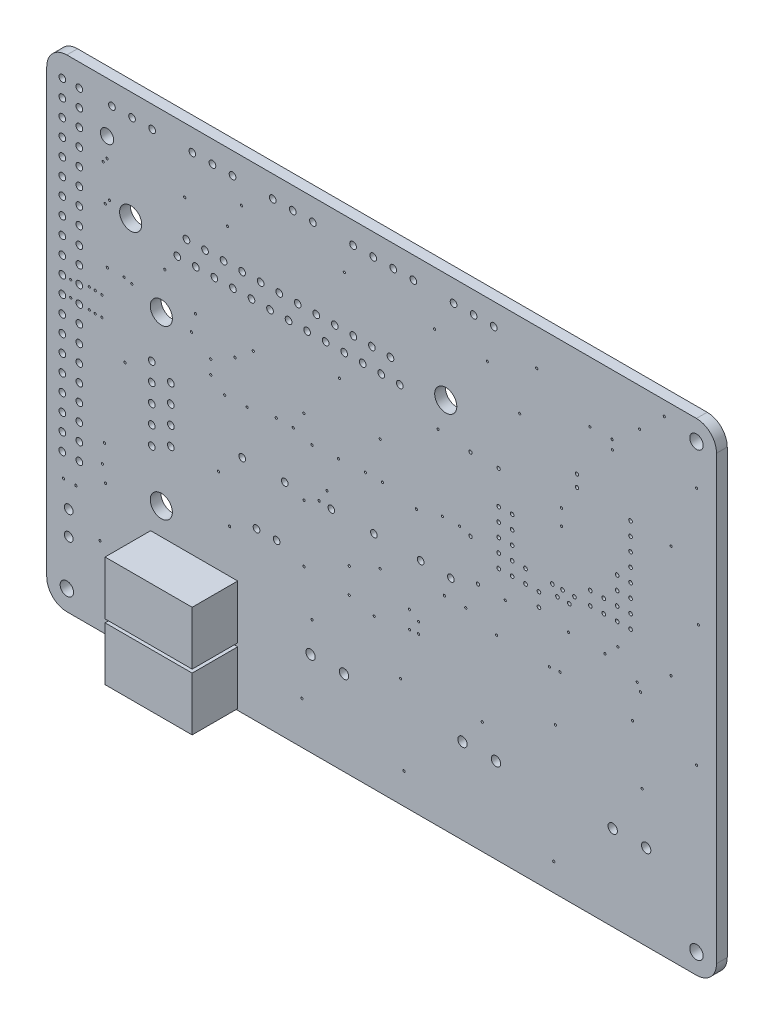
SolidWorks part; units mm, degrees
ref_plane "Front Plane" through (0, 0, 0) normal (0, 0, 1) x (1, 0, 0)
ref_plane "Top Plane" through (0, 0, 0) normal (0, 1, 0) x (1, 0, 0)
ref_plane "Right Plane" through (0, 0, 0) normal (1, 0, 0) x (0, 0, -1)
sketch "121" plane through (0, 0, 0) normal (0, 0, 1) x (1, 0, 0)
  line L0 (8, 71.008) -> (17.5, 71.008)
  line L1 (17.5, 71.008) -> (17.5, 67.524)
  line L2 (17.5, 67.524) -> (8, 67.524)
  line L3 (8, 67.524) -> (8, 71.008)
  line L4 (19.938, 71.008) -> (29.438, 71.008)
  line L5 (29.438, 71.008) -> (29.438, 67.524)
  line L6 (29.438, 67.524) -> (19.938, 67.524)
  line L7 (19.938, 67.524) -> (19.938, 71.008)
  line L8 (31.876, 71.008) -> (41.376, 71.008)
  line L9 (41.376, 71.008) -> (41.376, 67.524)
  line L10 (41.376, 67.524) -> (31.876, 67.524)
  line L11 (31.876, 67.524) -> (31.876, 71.008)
  line L12 (59.054, 71.008) -> (68.554, 71.008)
  line L13 (68.554, 71.008) -> (68.554, 67.524)
  line L14 (68.554, 67.524) -> (59.054, 67.524)
  line L15 (59.054, 67.524) -> (59.054, 71.008)
  line L16 (44.322, 71.008) -> (56.108, 71.008)
  line L17 (56.108, 71.008) -> (56.108, 67.524)
  line L18 (56.108, 67.524) -> (44.322, 67.524)
  line L19 (44.322, 67.524) -> (44.322, 71.008)
  line L20 (50.292, 67.564) -> (50.292, 68.715)
  line L21 (50.292, 69.715) -> (50.292, 70.866)
  line L22 (27.686, 34.544) -> (37.084, 34.544)
  line L23 (37.084, 34.544) -> (37.084, 29.464)
  line L24 (37.084, 29.464) -> (27.686, 29.464)
  line L25 (27.686, 29.464) -> (27.686, 34.544)
  line L26 (41.148, 34.544) -> (50.292, 34.544)
  line L27 (50.292, 34.544) -> (50.292, 29.464)
  line L28 (50.292, 29.464) -> (41.148, 29.464)
  line L29 (41.148, 29.464) -> (41.148, 34.544)
  line L30 (54.102, 34.544) -> (61.976, 34.544)
  line L31 (61.976, 34.544) -> (61.976, 29.464)
  line L32 (61.976, 29.464) -> (54.102, 29.464)
  line L33 (54.102, 29.464) -> (54.102, 34.544)
  line L34 (29.8704, 27.5336) -> (35.814, 27.5336)
  line L35 (35.814, 27.5336) -> (35.814, 22.2758)
  line L36 (35.814, 22.2758) -> (29.8704, 22.2758)
  line L37 (29.8704, 22.2758) -> (29.8704, 27.5336)
  line L38 (0.0254, 16.637) -> (5.3086, 16.637)
  line L39 (5.3086, 16.637) -> (5.3086, 6.5278)
  line L40 (5.3086, 6.5278) -> (0.0254, 6.5278)
  line L41 (0.0254, 6.5278) -> (0.0254, 16.637)
  line L42 (11.7667, 71.648) -> (11.7667, 71.2667)
  line L43 (11.7667, 71.2667) -> (11.9574, 71.2667)
  line L44 (11.9574, 71.2667) -> (12.0209, 71.3303)
  line L45 (12.0209, 71.3303) -> (12.0209, 71.5845)
  line L46 (12.0209, 71.5845) -> (11.9574, 71.648)
  line L47 (11.9574, 71.648) -> (11.7667, 71.648)
  line L48 (12.1409, 71.2667) -> (12.1409, 71.648)
  line L49 (12.1409, 71.4574) -> (12.3951, 71.4574)
  line L50 (12.3951, 71.648) -> (12.3951, 71.2667)
  line L51 (12.6422, 71.2667) -> (12.6422, 71.648)
  line L52 (12.5151, 71.648) -> (12.7693, 71.648)
  line L53 (12.8893, 71.4574) -> (13.1435, 71.4574)
  line L54 (13.2635, 71.2667) -> (13.3906, 71.2667)
  line L55 (13.3271, 71.2667) -> (13.3271, 71.648)
  line L56 (13.2635, 71.648) -> (13.3906, 71.648)
  line L57 (13.513, 71.2667) -> (13.513, 71.648)
  line L58 (13.513, 71.648) -> (13.7672, 71.2667)
  line L59 (13.7672, 71.2667) -> (13.7672, 71.648)
  line L60 (14.0143, 71.2667) -> (14.0143, 71.648)
  line L61 (13.8872, 71.648) -> (14.1414, 71.648)
  line L62 (9.2841, 70.4547) -> (9.7756, 70.4547)
  line L63 (9.5298, 70.7005) -> (9.5298, 70.209)
  line L64 (12.5903, 70.5955) -> (12.497, 70.6887)
  line L65 (12.497, 70.6887) -> (12.3106, 70.6887)
  line L66 (12.3106, 70.6887) -> (12.2174, 70.5955)
  line L67 (12.2174, 70.5955) -> (12.2174, 70.5023)
  line L68 (12.2174, 70.5023) -> (12.3106, 70.409)
  line L69 (12.3106, 70.409) -> (12.497, 70.409)
  line L70 (12.497, 70.409) -> (12.5903, 70.3158)
  line L71 (12.5903, 70.3158) -> (12.5903, 70.2226)
  line L72 (12.5903, 70.2226) -> (12.497, 70.1294)
  line L73 (12.497, 70.1294) -> (12.3106, 70.1294)
  line L74 (12.3106, 70.1294) -> (12.2174, 70.2226)
  line L75 (12.7787, 70.1294) -> (12.9651, 70.1294)
  line L76 (12.8719, 70.1294) -> (12.8719, 70.6887)
  line L77 (12.7787, 70.6887) -> (12.9651, 70.6887)
  line L78 (13.5258, 70.5955) -> (13.4326, 70.6887)
  line L79 (13.4326, 70.6887) -> (13.2461, 70.6887)
  line L80 (13.2461, 70.6887) -> (13.1529, 70.5955)
  line L81 (13.1529, 70.5955) -> (13.1529, 70.2226)
  line L82 (13.1529, 70.2226) -> (13.2461, 70.1294)
  line L83 (13.2461, 70.1294) -> (13.4326, 70.1294)
  line L84 (13.4326, 70.1294) -> (13.5258, 70.2226)
  line L85 (13.5258, 70.2226) -> (13.5258, 70.409)
  line L86 (13.5258, 70.409) -> (13.3393, 70.409)
  line L87 (15.5448, 70.4855) -> (16.3244, 70.4855)
  line L88 (23.7047, 71.648) -> (23.7047, 71.2667)
  line L89 (23.7047, 71.2667) -> (23.8954, 71.2667)
  line L90 (23.8954, 71.2667) -> (23.9589, 71.3303)
  line L91 (23.9589, 71.3303) -> (23.9589, 71.5845)
  line L92 (23.9589, 71.5845) -> (23.8954, 71.648)
  line L93 (23.8954, 71.648) -> (23.7047, 71.648)
  line L94 (24.0789, 71.2667) -> (24.0789, 71.648)
  line L95 (24.0789, 71.4574) -> (24.3331, 71.4574)
  line L96 (24.3331, 71.648) -> (24.3331, 71.2667)
  line L97 (24.5802, 71.2667) -> (24.5802, 71.648)
  line L98 (24.4531, 71.648) -> (24.7073, 71.648)
  line L99 (24.8273, 71.4574) -> (25.0815, 71.4574)
  line L100 (25.4557, 71.648) -> (25.2015, 71.648)
  line L101 (25.2015, 71.648) -> (25.2015, 71.2667)
  line L102 (25.2015, 71.2667) -> (25.4557, 71.2667)
  line L103 (25.2015, 71.4574) -> (25.3286, 71.4574)
  line L104 (25.5757, 71.648) -> (25.8299, 71.2667)
  line L105 (25.8299, 71.648) -> (25.5757, 71.2667)
  line L106 (26.077, 71.2667) -> (26.077, 71.648)
  line L107 (25.9499, 71.648) -> (26.2042, 71.648)
  line L108 (21.4761, 70.4547) -> (21.9676, 70.4547)
  line L109 (21.7218, 70.7005) -> (21.7218, 70.209)
  line L110 (24.5282, 70.5955) -> (24.435, 70.6887)
  line L111 (24.435, 70.6887) -> (24.2486, 70.6887)
  line L112 (24.2486, 70.6887) -> (24.1554, 70.5955)
  line L113 (24.1554, 70.5955) -> (24.1554, 70.5023)
  line L114 (24.1554, 70.5023) -> (24.2486, 70.409)
  line L115 (24.2486, 70.409) -> (24.435, 70.409)
  line L116 (24.435, 70.409) -> (24.5282, 70.3158)
  line L117 (24.5282, 70.3158) -> (24.5282, 70.2226)
  line L118 (24.5282, 70.2226) -> (24.435, 70.1294)
  line L119 (24.435, 70.1294) -> (24.2486, 70.1294)
  line L120 (24.2486, 70.1294) -> (24.1554, 70.2226)
  line L121 (24.7167, 70.1294) -> (24.9031, 70.1294)
  line L122 (24.8099, 70.1294) -> (24.8099, 70.6887)
  line L123 (24.7167, 70.6887) -> (24.9031, 70.6887)
  line L124 (25.4638, 70.5955) -> (25.3706, 70.6887)
  line L125 (25.3706, 70.6887) -> (25.1841, 70.6887)
  line L126 (25.1841, 70.6887) -> (25.0909, 70.5955)
  line L127 (25.0909, 70.5955) -> (25.0909, 70.2226)
  line L128 (25.0909, 70.2226) -> (25.1841, 70.1294)
  line L129 (25.1841, 70.1294) -> (25.3706, 70.1294)
  line L130 (25.3706, 70.1294) -> (25.4638, 70.2226)
  line L131 (25.4638, 70.2226) -> (25.4638, 70.409)
  line L132 (25.4638, 70.409) -> (25.2773, 70.409)
  line L133 (27.4828, 70.4855) -> (28.2624, 70.4855)
  line L134 (36.1509, 71.5845) -> (36.0874, 71.648)
  line L135 (36.0874, 71.648) -> (35.9603, 71.648)
  line L136 (35.9603, 71.648) -> (35.8967, 71.5845)
  line L137 (35.8967, 71.5845) -> (35.8967, 71.5209)
  line L138 (35.8967, 71.5209) -> (35.9603, 71.4574)
  line L139 (35.9603, 71.4574) -> (36.0874, 71.4574)
  line L140 (36.0874, 71.4574) -> (36.1509, 71.3938)
  line L141 (36.1509, 71.3938) -> (36.1509, 71.3303)
  line L142 (36.1509, 71.3303) -> (36.0874, 71.2667)
  line L143 (36.0874, 71.2667) -> (35.9603, 71.2667)
  line L144 (35.9603, 71.2667) -> (35.8967, 71.3303)
  line L145 (36.5251, 71.648) -> (36.2709, 71.648)
  line L146 (36.2709, 71.648) -> (36.2709, 71.2667)
  line L147 (36.2709, 71.2667) -> (36.5251, 71.2667)
  line L148 (36.2709, 71.4574) -> (36.398, 71.4574)
  line L149 (36.6451, 71.2667) -> (36.6451, 71.648)
  line L150 (36.6451, 71.648) -> (36.8358, 71.648)
  line L151 (36.8358, 71.648) -> (36.8993, 71.5845)
  line L152 (36.8993, 71.5845) -> (36.8993, 71.4574)
  line L153 (36.8993, 71.4574) -> (36.8358, 71.3938)
  line L154 (36.8358, 71.3938) -> (36.6451, 71.3938)
  line L155 (36.7722, 71.3938) -> (36.8993, 71.2667)
  line L156 (37.0193, 71.648) -> (37.0193, 71.3938)
  line L157 (37.0193, 71.3938) -> (37.1464, 71.2667)
  line L158 (37.1464, 71.2667) -> (37.2735, 71.3938)
  line L159 (37.2735, 71.3938) -> (37.2735, 71.648)
  line L160 (37.5842, 71.648) -> (37.4571, 71.648)
  line L161 (37.4571, 71.648) -> (37.3935, 71.5845)
  line L162 (37.3935, 71.5845) -> (37.3935, 71.3303)
  line L163 (37.3935, 71.3303) -> (37.4571, 71.2667)
  line L164 (37.4571, 71.2667) -> (37.5842, 71.2667)
  line L165 (37.5842, 71.2667) -> (37.6477, 71.3303)
  line L166 (37.6477, 71.3303) -> (37.6477, 71.5845)
  line L167 (37.6477, 71.5845) -> (37.5842, 71.648)
  line L168 (33.4141, 70.4547) -> (33.9056, 70.4547)
  line L169 (33.6598, 70.7005) -> (33.6598, 70.209)
  line L170 (35.8394, 70.1294) -> (35.8394, 70.6887)
  line L171 (35.8394, 70.6887) -> (36.119, 70.6887)
  line L172 (36.119, 70.6887) -> (36.2123, 70.5955)
  line L173 (36.2123, 70.5955) -> (36.2123, 70.409)
  line L174 (36.2123, 70.409) -> (36.119, 70.3158)
  line L175 (36.119, 70.3158) -> (35.8394, 70.3158)
  line L176 (36.4007, 70.6887) -> (36.4007, 70.1294)
  line L177 (36.4007, 70.1294) -> (36.5871, 70.3158)
  line L178 (36.5871, 70.3158) -> (36.7736, 70.1294)
  line L179 (36.7736, 70.1294) -> (36.7736, 70.6887)
  line L180 (36.962, 70.1294) -> (36.962, 70.6887)
  line L181 (36.962, 70.6887) -> (37.1484, 70.5023)
  line L182 (37.1484, 70.5023) -> (37.3349, 70.6887)
  line L183 (37.3349, 70.6887) -> (37.3349, 70.1294)
  line L184 (39.4208, 70.4855) -> (40.2004, 70.4855)
  line L185 (62.0587, 71.648) -> (62.0587, 71.2667)
  line L186 (62.0587, 71.2667) -> (62.3129, 71.2667)
  line L187 (62.4329, 71.2667) -> (62.56, 71.2667)
  line L188 (62.4965, 71.2667) -> (62.4965, 71.648)
  line L189 (62.4329, 71.648) -> (62.56, 71.648)
  line L190 (62.9366, 71.5845) -> (62.873, 71.648)
  line L191 (62.873, 71.648) -> (62.7459, 71.648)
  line L192 (62.7459, 71.648) -> (62.6824, 71.5845)
  line L193 (62.6824, 71.5845) -> (62.6824, 71.3303)
  line L194 (62.6824, 71.3303) -> (62.7459, 71.2667)
  line L195 (62.7459, 71.2667) -> (62.873, 71.2667)
  line L196 (62.873, 71.2667) -> (62.9366, 71.3303)
  line L197 (62.9366, 71.3303) -> (62.9366, 71.4574)
  line L198 (62.9366, 71.4574) -> (62.8095, 71.4574)
  line L199 (63.0566, 71.2667) -> (63.0566, 71.648)
  line L200 (63.0566, 71.4574) -> (63.3108, 71.4574)
  line L201 (63.3108, 71.648) -> (63.3108, 71.2667)
  line L202 (63.5579, 71.2667) -> (63.5579, 71.648)
  line L203 (63.4308, 71.648) -> (63.685, 71.648)
  line L204 (64.4334, 71.5845) -> (64.3699, 71.648)
  line L205 (64.3699, 71.648) -> (64.2428, 71.648)
  line L206 (64.2428, 71.648) -> (64.1792, 71.5845)
  line L207 (64.1792, 71.5845) -> (64.1792, 71.5209)
  line L208 (64.1792, 71.5209) -> (64.2428, 71.4574)
  line L209 (64.2428, 71.4574) -> (64.3699, 71.4574)
  line L210 (64.3699, 71.4574) -> (64.4334, 71.3938)
  line L211 (64.4334, 71.3938) -> (64.4334, 71.3303)
  line L212 (64.4334, 71.3303) -> (64.3699, 71.2667)
  line L213 (64.3699, 71.2667) -> (64.2428, 71.2667)
  line L214 (64.2428, 71.2667) -> (64.1792, 71.3303)
  line L215 (64.8076, 71.648) -> (64.5534, 71.648)
  line L216 (64.5534, 71.648) -> (64.5534, 71.2667)
  line L217 (64.5534, 71.2667) -> (64.8076, 71.2667)
  line L218 (64.5534, 71.4574) -> (64.6805, 71.4574)
  line L219 (64.9276, 71.2667) -> (64.9276, 71.648)
  line L220 (64.9276, 71.648) -> (65.1818, 71.2667)
  line L221 (65.1818, 71.2667) -> (65.1818, 71.648)
  line L222 (65.556, 71.5845) -> (65.4925, 71.648)
  line L223 (65.4925, 71.648) -> (65.3654, 71.648)
  line L224 (65.3654, 71.648) -> (65.3018, 71.5845)
  line L225 (65.3018, 71.5845) -> (65.3018, 71.5209)
  line L226 (65.3018, 71.5209) -> (65.3654, 71.4574)
  line L227 (65.3654, 71.4574) -> (65.4925, 71.4574)
  line L228 (65.4925, 71.4574) -> (65.556, 71.3938)
  line L229 (65.556, 71.3938) -> (65.556, 71.3303)
  line L230 (65.556, 71.3303) -> (65.4925, 71.2667)
  line L231 (65.4925, 71.2667) -> (65.3654, 71.2667)
  line L232 (65.3654, 71.2667) -> (65.3018, 71.3303)
  line L233 (65.8667, 71.648) -> (65.7396, 71.648)
  line L234 (65.7396, 71.648) -> (65.676, 71.5845)
  line L235 (65.676, 71.5845) -> (65.676, 71.3303)
  line L236 (65.676, 71.3303) -> (65.7396, 71.2667)
  line L237 (65.7396, 71.2667) -> (65.8667, 71.2667)
  line L238 (65.8667, 71.2667) -> (65.9302, 71.3303)
  line L239 (65.9302, 71.3303) -> (65.9302, 71.5845)
  line L240 (65.9302, 71.5845) -> (65.8667, 71.648)
  line L241 (66.0502, 71.2667) -> (66.0502, 71.648)
  line L242 (66.0502, 71.648) -> (66.2409, 71.648)
  line L243 (66.2409, 71.648) -> (66.3045, 71.5845)
  line L244 (66.3045, 71.5845) -> (66.3045, 71.4574)
  line L245 (66.3045, 71.4574) -> (66.2409, 71.3938)
  line L246 (66.2409, 71.3938) -> (66.0502, 71.3938)
  line L247 (66.1773, 71.3938) -> (66.3045, 71.2667)
  line L248 (60.3381, 70.4547) -> (60.8296, 70.4547)
  line L249 (60.5838, 70.7005) -> (60.5838, 70.209)
  line L250 (63.6442, 70.5955) -> (63.551, 70.6887)
  line L251 (63.551, 70.6887) -> (63.3646, 70.6887)
  line L252 (63.3646, 70.6887) -> (63.2714, 70.5955)
  line L253 (63.2714, 70.5955) -> (63.2714, 70.5023)
  line L254 (63.2714, 70.5023) -> (63.3646, 70.409)
  line L255 (63.3646, 70.409) -> (63.551, 70.409)
  line L256 (63.551, 70.409) -> (63.6442, 70.3158)
  line L257 (63.6442, 70.3158) -> (63.6442, 70.2226)
  line L258 (63.6442, 70.2226) -> (63.551, 70.1294)
  line L259 (63.551, 70.1294) -> (63.3646, 70.1294)
  line L260 (63.3646, 70.1294) -> (63.2714, 70.2226)
  line L261 (63.8327, 70.1294) -> (64.0191, 70.1294)
  line L262 (63.9259, 70.1294) -> (63.9259, 70.6887)
  line L263 (63.8327, 70.6887) -> (64.0191, 70.6887)
  line L264 (64.5798, 70.5955) -> (64.4866, 70.6887)
  line L265 (64.4866, 70.6887) -> (64.3001, 70.6887)
  line L266 (64.3001, 70.6887) -> (64.2069, 70.5955)
  line L267 (64.2069, 70.5955) -> (64.2069, 70.2226)
  line L268 (64.2069, 70.2226) -> (64.3001, 70.1294)
  line L269 (64.3001, 70.1294) -> (64.4866, 70.1294)
  line L270 (64.4866, 70.1294) -> (64.5798, 70.2226)
  line L271 (64.5798, 70.2226) -> (64.5798, 70.409)
  line L272 (64.5798, 70.409) -> (64.3933, 70.409)
  line L273 (66.5988, 70.4855) -> (67.3784, 70.4855)
  line L274 (48.5588, 71.5972) -> (48.4317, 71.5972)
  line L275 (48.4317, 71.5972) -> (48.3681, 71.5337)
  line L276 (48.3681, 71.5337) -> (48.3681, 71.2795)
  line L277 (48.3681, 71.2795) -> (48.4317, 71.2159)
  line L278 (48.4317, 71.2159) -> (48.5588, 71.2159)
  line L279 (48.5588, 71.2159) -> (48.6223, 71.2795)
  line L280 (48.6223, 71.2795) -> (48.6223, 71.5337)
  line L281 (48.6223, 71.5337) -> (48.5588, 71.5972)
  line L282 (48.7423, 71.2159) -> (48.7423, 71.5972)
  line L283 (48.7423, 71.5972) -> (48.933, 71.5972)
  line L284 (48.933, 71.5972) -> (48.9965, 71.5337)
  line L285 (48.9965, 71.5337) -> (48.9965, 71.4066)
  line L286 (48.9965, 71.4066) -> (48.933, 71.343)
  line L287 (48.933, 71.343) -> (48.7423, 71.343)
  line L288 (49.2436, 71.2159) -> (49.2436, 71.5972)
  line L289 (49.1165, 71.5972) -> (49.3707, 71.5972)
  line L290 (49.4907, 71.2159) -> (49.6178, 71.2159)
  line L291 (49.5543, 71.2159) -> (49.5543, 71.5972)
  line L292 (49.4907, 71.5972) -> (49.6178, 71.5972)
  line L293 (49.9944, 71.5337) -> (49.9309, 71.5972)
  line L294 (49.9309, 71.5972) -> (49.8037, 71.5972)
  line L295 (49.8037, 71.5972) -> (49.7402, 71.5337)
  line L296 (49.7402, 71.5337) -> (49.7402, 71.2795)
  line L297 (49.7402, 71.2795) -> (49.8037, 71.2159)
  line L298 (49.8037, 71.2159) -> (49.9309, 71.2159)
  line L299 (49.9309, 71.2159) -> (49.9944, 71.2795)
  line L300 (50.1144, 71.2159) -> (50.1144, 71.4701)
  line L301 (50.1144, 71.4701) -> (50.2415, 71.5972)
  line L302 (50.2415, 71.5972) -> (50.3686, 71.4701)
  line L303 (50.3686, 71.4701) -> (50.3686, 71.2159)
  line L304 (50.1144, 71.4066) -> (50.3686, 71.4066)
  line L305 (50.4886, 71.5972) -> (50.4886, 71.2159)
  line L306 (50.4886, 71.2159) -> (50.7428, 71.2159)
  line L307 (51.237, 71.2159) -> (51.237, 71.5972)
  line L308 (51.237, 71.5972) -> (51.4912, 71.5972)
  line L309 (51.237, 71.4066) -> (51.3641, 71.4066)
  line L310 (51.8019, 71.5972) -> (51.6748, 71.5972)
  line L311 (51.6748, 71.5972) -> (51.6112, 71.5337)
  line L312 (51.6112, 71.5337) -> (51.6112, 71.2795)
  line L313 (51.6112, 71.2795) -> (51.6748, 71.2159)
  line L314 (51.6748, 71.2159) -> (51.8019, 71.2159)
  line L315 (51.8019, 71.2159) -> (51.8654, 71.2795)
  line L316 (51.8654, 71.2795) -> (51.8654, 71.5337)
  line L317 (51.8654, 71.5337) -> (51.8019, 71.5972)
  line L318 (51.9854, 71.2159) -> (51.9854, 71.5972)
  line L319 (51.9854, 71.5972) -> (52.1761, 71.5972)
  line L320 (52.1761, 71.5972) -> (52.2396, 71.5337)
  line L321 (52.2396, 71.5337) -> (52.2396, 71.4066)
  line L322 (52.2396, 71.4066) -> (52.1761, 71.343)
  line L323 (52.1761, 71.343) -> (51.9854, 71.343)
  line L324 (52.1125, 71.343) -> (52.2396, 71.2159)
  line L325 (52.3596, 71.5972) -> (52.3596, 71.2159)
  line L326 (52.3596, 71.343) -> (52.6138, 71.5972)
  line L327 (52.4232, 71.4066) -> (52.6138, 71.2159)
  line L328 (45.3521, 70.4547) -> (45.8436, 70.4547)
  line L329 (45.5978, 70.7005) -> (45.5978, 70.209)
  line L330 (48.5648, 70.4855) -> (49.3444, 70.4855)
  line L331 (51.3461, 70.5107) -> (51.8376, 70.5107)
  line L332 (51.5918, 70.7565) -> (51.5918, 70.265)
  line L333 (54.7543, 70.5955) -> (54.661, 70.6887)
  line L334 (54.661, 70.6887) -> (54.4746, 70.6887)
  line L335 (54.4746, 70.6887) -> (54.3814, 70.5955)
  line L336 (54.3814, 70.5955) -> (54.3814, 70.5023)
  line L337 (54.3814, 70.5023) -> (54.4746, 70.409)
  line L338 (54.4746, 70.409) -> (54.661, 70.409)
  line L339 (54.661, 70.409) -> (54.7543, 70.3158)
  line L340 (54.7543, 70.3158) -> (54.7543, 70.2226)
  line L341 (54.7543, 70.2226) -> (54.661, 70.1294)
  line L342 (54.661, 70.1294) -> (54.4746, 70.1294)
  line L343 (54.4746, 70.1294) -> (54.3814, 70.2226)
  line L344 (54.9427, 70.1294) -> (55.1291, 70.1294)
  line L345 (55.0359, 70.1294) -> (55.0359, 70.6887)
  line L346 (54.9427, 70.6887) -> (55.1291, 70.6887)
  line L347 (55.6898, 70.5955) -> (55.5966, 70.6887)
  line L348 (55.5966, 70.6887) -> (55.4101, 70.6887)
  line L349 (55.4101, 70.6887) -> (55.3169, 70.5955)
  line L350 (55.3169, 70.5955) -> (55.3169, 70.2226)
  line L351 (55.3169, 70.2226) -> (55.4101, 70.1294)
  line L352 (55.4101, 70.1294) -> (55.5966, 70.1294)
  line L353 (55.5966, 70.1294) -> (55.6898, 70.2226)
  line L354 (55.6898, 70.2226) -> (55.6898, 70.409)
  line L355 (55.6898, 70.409) -> (55.5033, 70.409)
  line L356 (47.0029, 70.752) -> (46.7487, 70.752)
  line L357 (46.7487, 70.752) -> (46.7487, 70.3707)
  line L358 (46.7487, 70.3707) -> (47.0029, 70.3707)
  line L359 (46.7487, 70.5614) -> (46.8758, 70.5614)
  line L360 (47.1229, 70.3707) -> (47.1229, 70.752)
  line L361 (47.1229, 70.752) -> (47.25, 70.6249)
  line L362 (47.25, 70.6249) -> (47.3771, 70.752)
  line L363 (47.3771, 70.752) -> (47.3771, 70.3707)
  line L364 (47.4971, 70.3707) -> (47.6242, 70.3707)
  line L365 (47.5607, 70.3707) -> (47.5607, 70.752)
  line L366 (47.4971, 70.752) -> (47.6242, 70.752)
  line L367 (47.8737, 70.3707) -> (47.8737, 70.752)
  line L368 (47.7466, 70.752) -> (48.0008, 70.752)
  line L369 (52.5907, 70.3707) -> (52.5907, 70.752)
  line L370 (52.5907, 70.752) -> (52.7814, 70.752)
  line L371 (52.7814, 70.752) -> (52.8449, 70.6885)
  line L372 (52.8449, 70.6885) -> (52.8449, 70.5614)
  line L373 (52.8449, 70.5614) -> (52.7814, 70.4978)
  line L374 (52.7814, 70.4978) -> (52.5907, 70.4978)
  line L375 (52.7178, 70.4978) -> (52.8449, 70.3707)
  line L376 (53.2191, 70.752) -> (52.9649, 70.752)
  line L377 (52.9649, 70.752) -> (52.9649, 70.3707)
  line L378 (52.9649, 70.3707) -> (53.2191, 70.3707)
  line L379 (52.9649, 70.5614) -> (53.092, 70.5614)
  line L380 (53.5933, 70.6885) -> (53.5298, 70.752)
  line L381 (53.5298, 70.752) -> (53.4027, 70.752)
  line L382 (53.4027, 70.752) -> (53.3391, 70.6885)
  line L383 (53.3391, 70.6885) -> (53.3391, 70.4343)
  line L384 (53.3391, 70.4343) -> (53.4027, 70.3707)
  line L385 (53.4027, 70.3707) -> (53.5298, 70.3707)
  line L386 (53.5298, 70.3707) -> (53.5933, 70.4343)
  line L387 (31.0961, 29.8901) -> (31.0961, 30.6273)
  line L388 (31.0961, 30.2587) -> (31.5876, 30.2587)
  line L389 (31.5876, 30.6273) -> (31.5876, 29.8901)
  line L390 (32.336, 30.6273) -> (31.8445, 30.6273)
  line L391 (31.8445, 30.6273) -> (31.8445, 29.8901)
  line L392 (31.8445, 29.8901) -> (32.336, 29.8901)
  line L393 (31.8445, 30.2587) -> (32.0903, 30.2587)
  line L394 (32.5929, 29.8901) -> (32.5929, 30.3816)
  line L395 (32.5929, 30.3816) -> (32.8387, 30.6273)
  line L396 (32.8387, 30.6273) -> (33.0844, 30.3816)
  line L397 (33.0844, 30.3816) -> (33.0844, 29.8901)
  line L398 (32.5929, 30.2587) -> (33.0844, 30.2587)
  line L399 (33.5871, 29.8901) -> (33.5871, 30.6273)
  line L400 (33.3413, 30.6273) -> (33.8328, 30.6273)
  line L401 (34.9508, 31.0595) -> (35.7304, 31.0595)
  line L402 (35.3406, 31.4493) -> (35.3406, 30.6697)
  line L403 (28.7655, 31.0649) -> (29.7993, 31.0649)
  line L404 (43.7961, 30.6273) -> (43.7961, 29.8901)
  line L405 (43.7961, 29.8901) -> (44.1647, 29.8901)
  line L406 (44.1647, 29.8901) -> (44.2876, 30.013)
  line L407 (44.2876, 30.013) -> (44.2876, 30.5045)
  line L408 (44.2876, 30.5045) -> (44.1647, 30.6273)
  line L409 (44.1647, 30.6273) -> (43.7961, 30.6273)
  line L410 (45.036, 30.6273) -> (44.5445, 30.6273)
  line L411 (44.5445, 30.6273) -> (44.5445, 29.8901)
  line L412 (44.5445, 29.8901) -> (45.036, 29.8901)
  line L413 (44.5445, 30.2587) -> (44.7903, 30.2587)
  line L414 (45.2929, 29.8901) -> (45.2929, 30.6273)
  line L415 (45.2929, 30.2587) -> (45.7844, 30.2587)
  line L416 (45.7844, 30.6273) -> (45.7844, 29.8901)
  line L417 (46.0413, 30.6273) -> (46.0413, 30.013)
  line L418 (46.0413, 30.013) -> (46.1642, 29.8901)
  line L419 (46.1642, 29.8901) -> (46.41, 29.8901)
  line L420 (46.41, 29.8901) -> (46.5328, 30.013)
  line L421 (46.5328, 30.013) -> (46.5328, 30.6273)
  line L422 (46.7898, 29.8901) -> (46.7898, 30.6273)
  line L423 (46.7898, 30.6273) -> (47.0355, 30.3816)
  line L424 (47.0355, 30.3816) -> (47.2812, 30.6273)
  line L425 (47.2812, 30.6273) -> (47.2812, 29.8901)
  line L426 (48.4128, 31.0595) -> (49.1924, 31.0595)
  line L427 (48.8026, 31.4493) -> (48.8026, 30.6697)
  line L428 (42.2275, 31.0649) -> (43.2613, 31.0649)
  line L429 (57.2581, 29.8901) -> (57.2581, 30.6273)
  line L430 (57.2581, 30.6273) -> (57.7496, 30.6273)
  line L431 (57.2581, 30.2587) -> (57.5038, 30.2587)
  line L432 (58.0065, 29.8901) -> (58.0065, 30.3816)
  line L433 (58.0065, 30.3816) -> (58.2523, 30.6273)
  line L434 (58.2523, 30.6273) -> (58.498, 30.3816)
  line L435 (58.498, 30.3816) -> (58.498, 29.8901)
  line L436 (58.0065, 30.2587) -> (58.498, 30.2587)
  line L437 (58.7549, 29.8901) -> (58.7549, 30.6273)
  line L438 (58.7549, 30.6273) -> (59.2464, 29.8901)
  line L439 (59.2464, 29.8901) -> (59.2464, 30.6273)
  line L440 (59.8428, 31.0595) -> (60.6224, 31.0595)
  line L441 (60.2326, 31.4493) -> (60.2326, 30.6697)
  line L442 (55.4355, 31.0649) -> (56.4693, 31.0649)
  line L443 (34.2389, 39.0525) -> (34.2389, 39.544)
  line L444 (33.9931, 39.2982) -> (34.4846, 39.2982)
  line L445 (33.8703, 40.2924) -> (33.8703, 39.8009)
  line L446 (33.8703, 39.8009) -> (34.2389, 39.8009)
  line L447 (34.2389, 39.8009) -> (34.116, 40.0467)
  line L448 (34.116, 40.0467) -> (34.116, 40.1695)
  line L449 (34.116, 40.1695) -> (34.2389, 40.2924)
  line L450 (34.2389, 40.2924) -> (34.4846, 40.2924)
  line L451 (34.4846, 40.2924) -> (34.6075, 40.1695)
  line L452 (34.6075, 40.1695) -> (34.6075, 39.9238)
  line L453 (34.6075, 39.9238) -> (34.4846, 39.8009)
  line L454 (33.8703, 40.5493) -> (34.3618, 40.5493)
  line L455 (34.3618, 40.5493) -> (34.6075, 40.7951)
  line L456 (34.6075, 40.7951) -> (34.3618, 41.0408)
  line L457 (34.3618, 41.0408) -> (33.8703, 41.0408)
  line L458 (36.7281, 39.0271) -> (36.7281, 39.5186)
  line L459 (36.4823, 39.2728) -> (36.9738, 39.2728)
  line L460 (36.6052, 39.7755) -> (36.3595, 40.0213)
  line L461 (36.3595, 40.0213) -> (37.0967, 40.0213)
  line L462 (37.0967, 39.7755) -> (37.0967, 40.267)
  line L463 (37.0967, 41.0154) -> (37.0967, 40.5239)
  line L464 (37.0967, 40.5239) -> (36.6052, 41.0154)
  line L465 (36.6052, 41.0154) -> (36.4823, 41.0154)
  line L466 (36.4823, 41.0154) -> (36.3595, 40.8925)
  line L467 (36.3595, 40.8925) -> (36.3595, 40.6468)
  line L468 (36.3595, 40.6468) -> (36.4823, 40.5239)
  line L469 (36.3595, 41.2723) -> (36.851, 41.2723)
  line L470 (36.851, 41.2723) -> (37.0967, 41.5181)
  line L471 (37.0967, 41.5181) -> (36.851, 41.7638)
  line L472 (36.851, 41.7638) -> (36.3595, 41.7638)
  line L473 (50.0885, 38.7223) -> (50.0885, 39.2138)
  line L474 (49.8427, 38.968) -> (50.3342, 38.968)
  line L475 (49.9656, 39.4707) -> (49.7199, 39.7165)
  line L476 (49.7199, 39.7165) -> (50.4571, 39.7165)
  line L477 (50.4571, 39.4707) -> (50.4571, 39.9622)
  line L478 (50.4571, 40.7106) -> (50.4571, 40.2191)
  line L479 (50.4571, 40.2191) -> (49.9656, 40.7106)
  line L480 (49.9656, 40.7106) -> (49.8427, 40.7106)
  line L481 (49.8427, 40.7106) -> (49.7199, 40.5877)
  line L482 (49.7199, 40.5877) -> (49.7199, 40.342)
  line L483 (49.7199, 40.342) -> (49.8427, 40.2191)
  line L484 (49.7199, 40.9675) -> (50.2114, 40.9675)
  line L485 (50.2114, 40.9675) -> (50.4571, 41.2133)
  line L486 (50.4571, 41.2133) -> (50.2114, 41.459)
  line L487 (50.2114, 41.459) -> (49.7199, 41.459)
  line L488 (61.5947, 38.6461) -> (61.5947, 39.1376)
  line L489 (61.3489, 38.8918) -> (61.8404, 38.8918)
  line L490 (61.4718, 39.3945) -> (61.2261, 39.6403)
  line L491 (61.2261, 39.6403) -> (61.9633, 39.6403)
  line L492 (61.9633, 39.3945) -> (61.9633, 39.886)
  line L493 (61.9633, 40.6344) -> (61.9633, 40.1429)
  line L494 (61.9633, 40.1429) -> (61.4718, 40.6344)
  line L495 (61.4718, 40.6344) -> (61.3489, 40.6344)
  line L496 (61.3489, 40.6344) -> (61.2261, 40.5115)
  line L497 (61.2261, 40.5115) -> (61.2261, 40.2658)
  line L498 (61.2261, 40.2658) -> (61.3489, 40.1429)
  line L499 (61.2261, 40.8913) -> (61.7176, 40.8913)
  line L500 (61.7176, 40.8913) -> (61.9633, 41.1371)
  line L501 (61.9633, 41.1371) -> (61.7176, 41.3828)
  line L502 (61.7176, 41.3828) -> (61.2261, 41.3828)
  line L503 (59.0547, 38.6715) -> (59.0547, 39.163)
  line L504 (58.8089, 38.9172) -> (59.3004, 38.9172)
  line L505 (58.6861, 39.9114) -> (58.6861, 39.4199)
  line L506 (58.6861, 39.4199) -> (59.0547, 39.4199)
  line L507 (59.0547, 39.4199) -> (58.9318, 39.6657)
  line L508 (58.9318, 39.6657) -> (58.9318, 39.7885)
  line L509 (58.9318, 39.7885) -> (59.0547, 39.9114)
  line L510 (59.0547, 39.9114) -> (59.3004, 39.9114)
  line L511 (59.3004, 39.9114) -> (59.4233, 39.7885)
  line L512 (59.4233, 39.7885) -> (59.4233, 39.5428)
  line L513 (59.4233, 39.5428) -> (59.3004, 39.4199)
  line L514 (58.6861, 40.1683) -> (59.1776, 40.1683)
  line L515 (59.1776, 40.1683) -> (59.4233, 40.4141)
  line L516 (59.4233, 40.4141) -> (59.1776, 40.6598)
  line L517 (59.1776, 40.6598) -> (58.6861, 40.6598)
  line L518 (47.5231, 38.7223) -> (47.5231, 39.2138)
  line L519 (47.2773, 38.968) -> (47.7688, 38.968)
  line L520 (47.1545, 39.9622) -> (47.1545, 39.4707)
  line L521 (47.1545, 39.4707) -> (47.5231, 39.4707)
  line L522 (47.5231, 39.4707) -> (47.4002, 39.7165)
  line L523 (47.4002, 39.7165) -> (47.4002, 39.8393)
  line L524 (47.4002, 39.8393) -> (47.5231, 39.9622)
  line L525 (47.5231, 39.9622) -> (47.7688, 39.9622)
  line L526 (47.7688, 39.9622) -> (47.8917, 39.8393)
  line L527 (47.8917, 39.8393) -> (47.8917, 39.5936)
  line L528 (47.8917, 39.5936) -> (47.7688, 39.4707)
  line L529 (47.1545, 40.2191) -> (47.646, 40.2191)
  line L530 (47.646, 40.2191) -> (47.8917, 40.4649)
  line L531 (47.8917, 40.4649) -> (47.646, 40.7106)
  line L532 (47.646, 40.7106) -> (47.1545, 40.7106)
  line L533 (83.9728, 15.0575) -> (84.7524, 15.0575)
  line L534 (84.3626, 15.4473) -> (84.3626, 14.6677)
  line L535 (89.2175, 15.0629) -> (90.2513, 15.0629)
  line L536 (61.6208, 14.8035) -> (62.4004, 14.8035)
  line L537 (62.0106, 15.1933) -> (62.0106, 14.4137)
  line L538 (66.8655, 14.8089) -> (67.8993, 14.8089)
  line L539 (38.7608, 14.8035) -> (39.5404, 14.8035)
  line L540 (39.1506, 15.1933) -> (39.1506, 14.4137)
  line L541 (44.0055, 14.8089) -> (45.0393, 14.8089)
  line L542 (30.9691, 26.4611) -> (30.9691, 27.1983)
  line L543 (30.9691, 27.1983) -> (31.3377, 27.1983)
  line L544 (31.3377, 27.1983) -> (31.4606, 27.0755)
  line L545 (31.4606, 27.0755) -> (31.4606, 26.9526)
  line L546 (31.4606, 26.9526) -> (31.3377, 26.8297)
  line L547 (31.3377, 26.8297) -> (31.4606, 26.7068)
  line L548 (31.4606, 26.7068) -> (31.4606, 26.584)
  line L549 (31.4606, 26.584) -> (31.3377, 26.4611)
  line L550 (31.3377, 26.4611) -> (30.9691, 26.4611)
  line L551 (30.9691, 26.8297) -> (31.3377, 26.8297)
  line L552 (31.7175, 27.1983) -> (31.7175, 26.584)
  line L553 (31.7175, 26.584) -> (31.8404, 26.4611)
  line L554 (31.8404, 26.4611) -> (32.0861, 26.4611)
  line L555 (32.0861, 26.4611) -> (32.209, 26.584)
  line L556 (32.209, 26.584) -> (32.209, 27.1983)
  line L557 (32.4659, 27.1983) -> (32.9574, 27.1983)
  line L558 (32.9574, 27.1983) -> (32.9574, 27.0755)
  line L559 (32.9574, 27.0755) -> (32.4659, 26.584)
  line L560 (32.4659, 26.584) -> (32.4659, 26.4611)
  line L561 (32.4659, 26.4611) -> (32.9574, 26.4611)
  line L562 (33.2143, 27.1983) -> (33.7058, 27.1983)
  line L563 (33.7058, 27.1983) -> (33.7058, 27.0755)
  line L564 (33.7058, 27.0755) -> (33.2143, 26.584)
  line L565 (33.2143, 26.584) -> (33.2143, 26.4611)
  line L566 (33.2143, 26.4611) -> (33.7058, 26.4611)
  line L567 (34.4542, 27.1983) -> (33.9628, 27.1983)
  line L568 (33.9628, 27.1983) -> (33.9628, 26.4611)
  line L569 (33.9628, 26.4611) -> (34.4542, 26.4611)
  line L570 (33.9628, 26.8297) -> (34.2085, 26.8297)
  line L571 (34.7112, 26.4611) -> (34.7112, 27.1983)
  line L572 (34.7112, 27.1983) -> (35.0798, 27.1983)
  line L573 (35.0798, 27.1983) -> (35.2027, 27.0755)
  line L574 (35.2027, 27.0755) -> (35.2027, 26.8297)
  line L575 (35.2027, 26.8297) -> (35.0798, 26.7068)
  line L576 (35.0798, 26.7068) -> (34.7112, 26.7068)
  line L577 (34.9569, 26.7068) -> (35.2027, 26.4611)
  line L578 (30.8737, 23.2163) -> (31.9075, 23.2163)
  line L579 (33.7316, 23.1347) -> (34.5112, 23.1347)
  line L580 (34.1214, 23.5245) -> (34.1214, 22.7449)
  line L581 (33.7062, 23.1347) -> (34.4858, 23.1347)
  line L582 (34.096, 23.5245) -> (34.096, 22.7449)
  line L583 (1.2757, 9.1251) -> (0.5385, 9.1251)
  line L584 (0.5385, 9.1251) -> (0.5385, 9.4937)
  line L585 (0.5385, 9.4937) -> (0.6613, 9.6166)
  line L586 (0.6613, 9.6166) -> (0.9071, 9.6166)
  line L587 (0.9071, 9.6166) -> (1.03, 9.4937)
  line L588 (1.03, 9.4937) -> (1.03, 9.1251)
  line L589 (0.5385, 10.2421) -> (0.5385, 9.9964)
  line L590 (0.5385, 9.9964) -> (0.6613, 9.8735)
  line L591 (0.6613, 9.8735) -> (1.1528, 9.8735)
  line L592 (1.1528, 9.8735) -> (1.2757, 9.9964)
  line L593 (1.2757, 9.9964) -> (1.2757, 10.2421)
  line L594 (1.2757, 10.2421) -> (1.1528, 10.365)
  line L595 (1.1528, 10.365) -> (0.6613, 10.365)
  line L596 (0.6613, 10.365) -> (0.5385, 10.2421)
  line L597 (0.5385, 10.6219) -> (1.2757, 10.6219)
  line L598 (1.2757, 10.6219) -> (1.03, 10.8677)
  line L599 (1.03, 10.8677) -> (1.2757, 11.1134)
  line L600 (1.2757, 11.1134) -> (0.5385, 11.1134)
  line L601 (0.5385, 11.8618) -> (0.5385, 11.3703)
  line L602 (0.5385, 11.3703) -> (1.2757, 11.3703)
  line L603 (1.2757, 11.3703) -> (1.2757, 11.8618)
  line L604 (0.9071, 11.3703) -> (0.9071, 11.6161)
  line L605 (1.2757, 12.1188) -> (0.5385, 12.1188)
  line L606 (0.5385, 12.1188) -> (0.5385, 12.4874)
  line L607 (0.5385, 12.4874) -> (0.6613, 12.6102)
  line L608 (0.6613, 12.6102) -> (0.9071, 12.6102)
  line L609 (0.9071, 12.6102) -> (1.03, 12.4874)
  line L610 (1.03, 12.4874) -> (1.03, 12.1188)
  line L611 (1.03, 12.3645) -> (1.2757, 12.6102)
  line L612 (1.2757, 13.6156) -> (1.2757, 13.8613)
  line L613 (1.2757, 13.7385) -> (0.5385, 13.7385)
  line L614 (0.5385, 13.6156) -> (0.5385, 13.8613)
  line L615 (1.2757, 14.1145) -> (0.5385, 14.1145)
  line L616 (0.5385, 14.1145) -> (1.2757, 14.606)
  line L617 (1.2757, 14.606) -> (0.5385, 14.606)
  line L618 (1.8669, 15.7229) -> (2.3584, 15.7229)
  line L619 (2.1126, 15.9687) -> (2.1126, 15.4772)
  line L620 (2.6153, 15.8458) -> (2.8611, 16.0915)
  line L621 (2.8611, 16.0915) -> (2.8611, 15.3543)
  line L622 (2.6153, 15.3543) -> (3.1068, 15.3543)
  line L623 (3.8552, 15.3543) -> (3.3637, 15.3543)
  line L624 (3.3637, 15.3543) -> (3.8552, 15.8458)
  line L625 (3.8552, 15.8458) -> (3.8552, 15.9687)
  line L626 (3.8552, 15.9687) -> (3.7323, 16.0915)
  line L627 (3.7323, 16.0915) -> (3.4866, 16.0915)
  line L628 (3.4866, 16.0915) -> (3.3637, 15.9687)
  line L629 (4.1121, 16.0915) -> (4.1121, 15.6)
  line L630 (4.1121, 15.6) -> (4.3579, 15.3543)
  line L631 (4.3579, 15.3543) -> (4.6036, 15.6)
  line L632 (4.6036, 15.6) -> (4.6036, 16.0915)
  line L633 (2.6124, 7.5105) -> (2.4895, 7.6333)
  line L634 (2.4895, 7.6333) -> (2.2438, 7.6333)
  line L635 (2.2438, 7.6333) -> (2.1209, 7.5105)
  line L636 (2.1209, 7.5105) -> (2.1209, 7.019)
  line L637 (2.1209, 7.019) -> (2.2438, 6.8961)
  line L638 (2.2438, 6.8961) -> (2.4895, 6.8961)
  line L639 (2.4895, 6.8961) -> (2.6124, 7.019)
  line L640 (2.6124, 7.019) -> (2.6124, 7.2647)
  line L641 (2.6124, 7.2647) -> (2.3666, 7.2647)
  line L642 (2.8693, 6.8961) -> (2.8693, 7.6333)
  line L643 (2.8693, 7.6333) -> (3.3608, 6.8961)
  line L644 (3.3608, 6.8961) -> (3.3608, 7.6333)
  line L645 (3.6177, 7.6333) -> (3.6177, 6.8961)
  line L646 (3.6177, 6.8961) -> (3.9863, 6.8961)
  line L647 (3.9863, 6.8961) -> (4.1092, 7.019)
  line L648 (4.1092, 7.019) -> (4.1092, 7.5105)
  line L649 (4.1092, 7.5105) -> (3.9863, 7.6333)
  line L650 (3.9863, 7.6333) -> (3.6177, 7.6333)
  arc A0 (17.5, 70.983) -> (17.5, 71.033) centre (17.5, 71.008) ccw
  arc A1 (8, 71.033) -> (8, 70.983) centre (8, 71.008) ccw
  arc A2 (17.475, 67.524) -> (17.525, 67.524) centre (17.5, 67.524) ccw
  arc A3 (17.525, 71.008) -> (17.475, 71.008) centre (17.5, 71.008) ccw
  arc A4 (8, 67.549) -> (8, 67.499) centre (8, 67.524) ccw
  arc A5 (17.5, 67.499) -> (17.5, 67.549) centre (17.5, 67.524) ccw
  arc A6 (8.025, 71.008) -> (7.975, 71.008) centre (8, 71.008) ccw
  arc A7 (7.975, 67.524) -> (8.025, 67.524) centre (8, 67.524) ccw
  arc A8 (29.438, 70.983) -> (29.438, 71.033) centre (29.438, 71.008) ccw
  arc A9 (19.938, 71.033) -> (19.938, 70.983) centre (19.938, 71.008) ccw
  arc A10 (29.413, 67.524) -> (29.463, 67.524) centre (29.438, 67.524) ccw
  arc A11 (29.463, 71.008) -> (29.413, 71.008) centre (29.438, 71.008) ccw
  arc A12 (19.938, 67.549) -> (19.938, 67.499) centre (19.938, 67.524) ccw
  arc A13 (29.438, 67.499) -> (29.438, 67.549) centre (29.438, 67.524) ccw
  arc A14 (19.963, 71.008) -> (19.913, 71.008) centre (19.938, 71.008) ccw
  arc A15 (19.913, 67.524) -> (19.963, 67.524) centre (19.938, 67.524) ccw
  arc A16 (41.376, 70.983) -> (41.376, 71.033) centre (41.376, 71.008) ccw
  arc A17 (31.876, 71.033) -> (31.876, 70.983) centre (31.876, 71.008) ccw
  arc A18 (41.351, 67.524) -> (41.401, 67.524) centre (41.376, 67.524) ccw
  arc A19 (41.401, 71.008) -> (41.351, 71.008) centre (41.376, 71.008) ccw
  arc A20 (31.876, 67.549) -> (31.876, 67.499) centre (31.876, 67.524) ccw
  arc A21 (41.376, 67.499) -> (41.376, 67.549) centre (41.376, 67.524) ccw
  arc A22 (31.901, 71.008) -> (31.851, 71.008) centre (31.876, 71.008) ccw
  arc A23 (31.851, 67.524) -> (31.901, 67.524) centre (31.876, 67.524) ccw
  arc A24 (68.554, 70.983) -> (68.554, 71.033) centre (68.554, 71.008) ccw
  arc A25 (59.054, 71.033) -> (59.054, 70.983) centre (59.054, 71.008) ccw
  arc A26 (68.529, 67.524) -> (68.579, 67.524) centre (68.554, 67.524) ccw
  arc A27 (68.579, 71.008) -> (68.529, 71.008) centre (68.554, 71.008) ccw
  arc A28 (59.054, 67.549) -> (59.054, 67.499) centre (59.054, 67.524) ccw
  arc A29 (68.554, 67.499) -> (68.554, 67.549) centre (68.554, 67.524) ccw
  arc A30 (59.079, 71.008) -> (59.029, 71.008) centre (59.054, 71.008) ccw
  arc A31 (59.029, 67.524) -> (59.079, 67.524) centre (59.054, 67.524) ccw
  arc A32 (56.108, 70.983) -> (56.108, 71.033) centre (56.108, 71.008) ccw
  arc A33 (44.322, 71.033) -> (44.322, 70.983) centre (44.322, 71.008) ccw
  arc A34 (56.083, 67.524) -> (56.133, 67.524) centre (56.108, 67.524) ccw
  arc A35 (56.133, 71.008) -> (56.083, 71.008) centre (56.108, 71.008) ccw
  arc A36 (44.322, 67.549) -> (44.322, 67.499) centre (44.322, 67.524) ccw
  arc A37 (56.108, 67.499) -> (56.108, 67.549) centre (56.108, 67.524) ccw
  arc A38 (44.347, 71.008) -> (44.297, 71.008) centre (44.322, 71.008) ccw
  arc A39 (44.297, 67.524) -> (44.347, 67.524) centre (44.322, 67.524) ccw
  arc A40 (50.317, 68.715) -> (50.267, 68.715) centre (50.292, 68.715) ccw
  arc A41 (50.267, 67.564) -> (50.317, 67.564) centre (50.292, 67.564) ccw
  arc A42 (50.317, 70.866) -> (50.267, 70.866) centre (50.292, 70.866) ccw
  arc A43 (50.267, 69.715) -> (50.317, 69.715) centre (50.292, 69.715) ccw
  arc A44 (37.084, 34.519) -> (37.084, 34.569) centre (37.084, 34.544) ccw
  arc A45 (27.686, 34.569) -> (27.686, 34.519) centre (27.686, 34.544) ccw
  arc A46 (37.059, 29.464) -> (37.109, 29.464) centre (37.084, 29.464) ccw
  arc A47 (37.109, 34.544) -> (37.059, 34.544) centre (37.084, 34.544) ccw
  arc A48 (27.686, 29.489) -> (27.686, 29.439) centre (27.686, 29.464) ccw
  arc A49 (37.084, 29.439) -> (37.084, 29.489) centre (37.084, 29.464) ccw
  arc A50 (27.711, 34.544) -> (27.661, 34.544) centre (27.686, 34.544) ccw
  arc A51 (27.661, 29.464) -> (27.711, 29.464) centre (27.686, 29.464) ccw
  arc A52 (50.292, 34.519) -> (50.292, 34.569) centre (50.292, 34.544) ccw
  arc A53 (41.148, 34.569) -> (41.148, 34.519) centre (41.148, 34.544) ccw
  arc A54 (50.267, 29.464) -> (50.317, 29.464) centre (50.292, 29.464) ccw
  arc A55 (50.317, 34.544) -> (50.267, 34.544) centre (50.292, 34.544) ccw
  arc A56 (41.148, 29.489) -> (41.148, 29.439) centre (41.148, 29.464) ccw
  arc A57 (50.292, 29.439) -> (50.292, 29.489) centre (50.292, 29.464) ccw
  arc A58 (41.173, 34.544) -> (41.123, 34.544) centre (41.148, 34.544) ccw
  arc A59 (41.123, 29.464) -> (41.173, 29.464) centre (41.148, 29.464) ccw
  arc A60 (61.976, 34.519) -> (61.976, 34.569) centre (61.976, 34.544) ccw
  arc A61 (54.102, 34.569) -> (54.102, 34.519) centre (54.102, 34.544) ccw
  arc A62 (61.951, 29.464) -> (62.001, 29.464) centre (61.976, 29.464) ccw
  arc A63 (62.001, 34.544) -> (61.951, 34.544) centre (61.976, 34.544) ccw
  arc A64 (54.102, 29.489) -> (54.102, 29.439) centre (54.102, 29.464) ccw
  arc A65 (61.976, 29.439) -> (61.976, 29.489) centre (61.976, 29.464) ccw
  arc A66 (54.127, 34.544) -> (54.077, 34.544) centre (54.102, 34.544) ccw
  arc A67 (54.077, 29.464) -> (54.127, 29.464) centre (54.102, 29.464) ccw
  arc A68 (35.814, 27.5086) -> (35.814, 27.5586) centre (35.814, 27.5336) ccw
  arc A69 (29.8704, 27.5586) -> (29.8704, 27.5086) centre (29.8704, 27.5336) ccw
  arc A70 (35.789, 22.2758) -> (35.839, 22.2758) centre (35.814, 22.2758) ccw
  arc A71 (35.839, 27.5336) -> (35.789, 27.5336) centre (35.814, 27.5336) ccw
  arc A72 (29.8704, 22.3008) -> (29.8704, 22.2508) centre (29.8704, 22.2758) ccw
  arc A73 (35.814, 22.2508) -> (35.814, 22.3008) centre (35.814, 22.2758) ccw
  arc A74 (29.8954, 27.5336) -> (29.8454, 27.5336) centre (29.8704, 27.5336) ccw
  arc A75 (29.8454, 22.2758) -> (29.8954, 22.2758) centre (29.8704, 22.2758) ccw
  arc A76 (5.3086, 16.612) -> (5.3086, 16.662) centre (5.3086, 16.637) ccw
  arc A77 (0.0254, 16.662) -> (0.0254, 16.612) centre (0.0254, 16.637) ccw
  arc A78 (5.2836, 6.5278) -> (5.3336, 6.5278) centre (5.3086, 6.5278) ccw
  arc A79 (5.3336, 16.637) -> (5.2836, 16.637) centre (5.3086, 16.637) ccw
  arc A80 (0.0254, 6.5528) -> (0.0254, 6.5028) centre (0.0254, 6.5278) ccw
  arc A81 (5.3086, 6.5028) -> (5.3086, 6.5528) centre (5.3086, 6.5278) ccw
  arc A82 (0.0504, 16.637) -> (0.0004, 16.637) centre (0.0254, 16.637) ccw
  arc A83 (0.0004, 6.5278) -> (0.0504, 6.5278) centre (0.0254, 6.5278) ccw
  arc A84 (11.7604, 71.2667) -> (11.773, 71.2667) centre (11.7667, 71.2667) ccw
  arc A85 (11.773, 71.648) -> (11.7604, 71.648) centre (11.7667, 71.648) ccw
  arc A86 (11.9574, 71.2604) -> (11.9574, 71.273) centre (11.9574, 71.2667) ccw
  arc A87 (11.7667, 71.273) -> (11.7667, 71.2604) centre (11.7667, 71.2667) ccw
  arc A88 (12.0254, 71.3258) -> (12.0164, 71.3347) centre (12.0209, 71.3303) ccw
  arc A89 (11.9529, 71.2712) -> (11.9619, 71.2622) centre (11.9574, 71.2667) ccw
  arc A90 (12.0273, 71.5845) -> (12.0146, 71.5845) centre (12.021, 71.5845) ccw
  arc A91 (12.0146, 71.3303) -> (12.0273, 71.3303) centre (12.021, 71.3303) ccw
  arc A92 (11.9619, 71.6525) -> (11.9529, 71.6435) centre (11.9574, 71.648) ccw
  arc A93 (12.0164, 71.58) -> (12.0254, 71.589) centre (12.0209, 71.5845) ccw
  arc A94 (11.7667, 71.6544) -> (11.7667, 71.6417) centre (11.7667, 71.648) ccw
  arc A95 (11.9574, 71.6417) -> (11.9574, 71.6544) centre (11.9574, 71.648) ccw
  arc A96 (12.1473, 71.648) -> (12.1346, 71.648) centre (12.141, 71.648) ccw
  arc A97 (12.1346, 71.2667) -> (12.1473, 71.2667) centre (12.141, 71.2667) ccw
  arc A98 (12.3951, 71.451) -> (12.3951, 71.4637) centre (12.3951, 71.4574) ccw
  arc A99 (12.1409, 71.4637) -> (12.1409, 71.451) centre (12.1409, 71.4574) ccw
  arc A100 (12.3888, 71.2667) -> (12.4015, 71.2667) centre (12.3952, 71.2667) ccw
  arc A101 (12.4015, 71.648) -> (12.3888, 71.648) centre (12.3952, 71.648) ccw
  arc A102 (12.6486, 71.648) -> (12.6359, 71.648) centre (12.6423, 71.648) ccw
  arc A103 (12.6359, 71.2667) -> (12.6486, 71.2667) centre (12.6423, 71.2667) ccw
  arc A104 (12.7693, 71.6417) -> (12.7693, 71.6544) centre (12.7693, 71.648) ccw
  arc A105 (12.5151, 71.6544) -> (12.5151, 71.6417) centre (12.5151, 71.648) ccw
  arc A106 (13.1435, 71.451) -> (13.1435, 71.4637) centre (13.1435, 71.4574) ccw
  arc A107 (12.8893, 71.4637) -> (12.8893, 71.451) centre (12.8893, 71.4574) ccw
  arc A108 (13.3906, 71.2604) -> (13.3906, 71.273) centre (13.3906, 71.2667) ccw
  arc A109 (13.2635, 71.273) -> (13.2635, 71.2604) centre (13.2635, 71.2667) ccw
  arc A110 (13.3334, 71.648) -> (13.3207, 71.648) centre (13.327, 71.648) ccw
  arc A111 (13.3207, 71.2667) -> (13.3334, 71.2667) centre (13.327, 71.2667) ccw
  arc A112 (13.3906, 71.6417) -> (13.3906, 71.6544) centre (13.3906, 71.648) ccw
  arc A113 (13.2635, 71.6544) -> (13.2635, 71.6417) centre (13.2635, 71.648) ccw
  arc A114 (13.5193, 71.648) -> (13.5066, 71.648) centre (13.513, 71.648) ccw
  arc A115 (13.5066, 71.2667) -> (13.5193, 71.2667) centre (13.513, 71.2667) ccw
  arc A116 (13.7619, 71.2632) -> (13.7725, 71.2702) centre (13.7672, 71.2667) ccw
  arc A117 (13.5183, 71.6515) -> (13.5077, 71.6445) centre (13.513, 71.648) ccw
  arc A118 (13.7736, 71.648) -> (13.7609, 71.648) centre (13.7673, 71.648) ccw
  arc A119 (13.7609, 71.2667) -> (13.7736, 71.2667) centre (13.7673, 71.2667) ccw
  arc A120 (14.0207, 71.648) -> (14.008, 71.648) centre (14.0144, 71.648) ccw
  arc A121 (14.008, 71.2667) -> (14.0207, 71.2667) centre (14.0144, 71.2667) ccw
  arc A122 (14.1414, 71.6417) -> (14.1414, 71.6544) centre (14.1414, 71.648) ccw
  arc A123 (13.8872, 71.6544) -> (13.8872, 71.6417) centre (13.8872, 71.648) ccw
  arc A124 (9.7756, 70.4357) -> (9.7756, 70.4738) centre (9.7756, 70.4548) ccw
  arc A125 (9.2841, 70.4738) -> (9.2841, 70.4357) centre (9.2841, 70.4548) ccw
  arc A126 (9.5108, 70.209) -> (9.5489, 70.209) centre (9.5298, 70.209) ccw
  arc A127 (9.5489, 70.7005) -> (9.5108, 70.7005) centre (9.5298, 70.7005) ccw
  arc A128 (12.506, 70.6977) -> (12.4881, 70.6797) centre (12.497, 70.6887) ccw
  arc A129 (12.5813, 70.5865) -> (12.5992, 70.6044) centre (12.5903, 70.5954) ccw
  arc A130 (12.3106, 70.7014) -> (12.3106, 70.676) centre (12.3106, 70.6887) ccw
  arc A131 (12.497, 70.676) -> (12.497, 70.7014) centre (12.497, 70.6887) ccw
  arc A132 (12.2084, 70.6044) -> (12.2264, 70.5865) centre (12.2174, 70.5954) ccw
  arc A133 (12.3196, 70.6797) -> (12.3016, 70.6977) centre (12.3106, 70.6887) ccw
  arc A134 (12.2047, 70.5023) -> (12.2301, 70.5023) centre (12.2174, 70.5023) ccw
  arc A135 (12.2301, 70.5955) -> (12.2047, 70.5955) centre (12.2174, 70.5955) ccw
  arc A136 (12.3016, 70.4001) -> (12.3196, 70.418) centre (12.3106, 70.4091) ccw
  arc A137 (12.2264, 70.5112) -> (12.2084, 70.4933) centre (12.2174, 70.5023) ccw
  arc A138 (12.497, 70.3963) -> (12.497, 70.4217) centre (12.497, 70.409) ccw
  arc A139 (12.3106, 70.4217) -> (12.3106, 70.3963) centre (12.3106, 70.409) ccw
  arc A140 (12.5813, 70.3068) -> (12.5992, 70.3248) centre (12.5903, 70.3158) ccw
  arc A141 (12.506, 70.418) -> (12.4881, 70.4001) centre (12.497, 70.4091) ccw
  arc A142 (12.5776, 70.2226) -> (12.603, 70.2226) centre (12.5903, 70.2226) ccw
  arc A143 (12.603, 70.3158) -> (12.5776, 70.3158) centre (12.5903, 70.3158) ccw
  arc A144 (12.4881, 70.1384) -> (12.506, 70.1204) centre (12.497, 70.1294) ccw
  arc A145 (12.5992, 70.2136) -> (12.5813, 70.2316) centre (12.5903, 70.2226) ccw
  arc A146 (12.3106, 70.1421) -> (12.3106, 70.1167) centre (12.3106, 70.1294) ccw
  arc A147 (12.497, 70.1167) -> (12.497, 70.1421) centre (12.497, 70.1294) ccw
  arc A148 (12.2264, 70.2316) -> (12.2084, 70.2136) centre (12.2174, 70.2226) ccw
  arc A149 (12.3016, 70.1204) -> (12.3196, 70.1384) centre (12.3106, 70.1294) ccw
  arc A150 (12.9651, 70.1167) -> (12.9651, 70.1421) centre (12.9651, 70.1294) ccw
  arc A151 (12.7787, 70.1421) -> (12.7787, 70.1167) centre (12.7787, 70.1294) ccw
  arc A152 (12.8846, 70.6887) -> (12.8592, 70.6887) centre (12.8719, 70.6887) ccw
  arc A153 (12.8592, 70.1294) -> (12.8846, 70.1294) centre (12.8719, 70.1294) ccw
  arc A154 (12.9651, 70.676) -> (12.9651, 70.7014) centre (12.9651, 70.6887) ccw
  arc A155 (12.7787, 70.7014) -> (12.7787, 70.676) centre (12.7787, 70.6887) ccw
  arc A156 (13.4415, 70.6977) -> (13.4236, 70.6797) centre (13.4326, 70.6887) ccw
  arc A157 (13.5168, 70.5865) -> (13.5347, 70.6044) centre (13.5258, 70.5954) ccw
  arc A158 (13.2461, 70.7014) -> (13.2461, 70.676) centre (13.2461, 70.6887) ccw
  arc A159 (13.4326, 70.676) -> (13.4326, 70.7014) centre (13.4326, 70.6887) ccw
  arc A160 (13.1439, 70.6044) -> (13.1619, 70.5865) centre (13.1529, 70.5954) ccw
  arc A161 (13.2551, 70.6797) -> (13.2371, 70.6977) centre (13.2461, 70.6887) ccw
  arc A162 (13.1402, 70.2226) -> (13.1656, 70.2226) centre (13.1529, 70.2226) ccw
  arc A163 (13.1656, 70.5955) -> (13.1402, 70.5955) centre (13.1529, 70.5955) ccw
  arc A164 (13.2371, 70.1204) -> (13.2551, 70.1384) centre (13.2461, 70.1294) ccw
  arc A165 (13.1619, 70.2316) -> (13.1439, 70.2136) centre (13.1529, 70.2226) ccw
  arc A166 (13.4326, 70.1167) -> (13.4326, 70.1421) centre (13.4326, 70.1294) ccw
  arc A167 (13.2461, 70.1421) -> (13.2461, 70.1167) centre (13.2461, 70.1294) ccw
  arc A168 (13.5347, 70.2136) -> (13.5168, 70.2316) centre (13.5258, 70.2226) ccw
  arc A169 (13.4236, 70.1384) -> (13.4415, 70.1204) centre (13.4326, 70.1294) ccw
  arc A170 (13.5385, 70.409) -> (13.5131, 70.409) centre (13.5258, 70.409) ccw
  arc A171 (13.5131, 70.2226) -> (13.5385, 70.2226) centre (13.5258, 70.2226) ccw
  arc A172 (13.3393, 70.4217) -> (13.3393, 70.3963) centre (13.3393, 70.409) ccw
  arc A173 (13.5258, 70.3963) -> (13.5258, 70.4217) centre (13.5258, 70.409) ccw
  arc A174 (16.3244, 70.4601) -> (16.3244, 70.5109) centre (16.3244, 70.4855) ccw
  arc A175 (15.5448, 70.5109) -> (15.5448, 70.4601) centre (15.5448, 70.4855) ccw
  arc A176 (23.6984, 71.2667) -> (23.7111, 71.2667) centre (23.7048, 71.2667) ccw
  arc A177 (23.7111, 71.648) -> (23.6984, 71.648) centre (23.7048, 71.648) ccw
  arc A178 (23.8954, 71.2604) -> (23.8954, 71.273) centre (23.8954, 71.2667) ccw
  arc A179 (23.7047, 71.273) -> (23.7047, 71.2604) centre (23.7047, 71.2667) ccw
  arc A180 (23.9634, 71.3258) -> (23.9544, 71.3347) centre (23.9589, 71.3303) ccw
  arc A181 (23.8909, 71.2712) -> (23.8999, 71.2622) centre (23.8954, 71.2667) ccw
  arc A182 (23.9653, 71.5845) -> (23.9526, 71.5845) centre (23.9589, 71.5845) ccw
  arc A183 (23.9526, 71.3303) -> (23.9653, 71.3303) centre (23.9589, 71.3303) ccw
  arc A184 (23.8999, 71.6525) -> (23.8909, 71.6435) centre (23.8954, 71.648) ccw
  arc A185 (23.9544, 71.58) -> (23.9634, 71.589) centre (23.9589, 71.5845) ccw
  arc A186 (23.7047, 71.6544) -> (23.7047, 71.6417) centre (23.7047, 71.648) ccw
  arc A187 (23.8954, 71.6417) -> (23.8954, 71.6544) centre (23.8954, 71.648) ccw
  arc A188 (24.0853, 71.648) -> (24.0726, 71.648) centre (24.079, 71.648) ccw
  arc A189 (24.0726, 71.2667) -> (24.0853, 71.2667) centre (24.079, 71.2667) ccw
  arc A190 (24.3331, 71.451) -> (24.3331, 71.4637) centre (24.3331, 71.4574) ccw
  arc A191 (24.0789, 71.4637) -> (24.0789, 71.451) centre (24.0789, 71.4574) ccw
  arc A192 (24.3268, 71.2667) -> (24.3395, 71.2667) centre (24.3331, 71.2667) ccw
  arc A193 (24.3395, 71.648) -> (24.3268, 71.648) centre (24.3331, 71.648) ccw
  arc A194 (24.5866, 71.648) -> (24.5739, 71.648) centre (24.5802, 71.648) ccw
  arc A195 (24.5739, 71.2667) -> (24.5866, 71.2667) centre (24.5802, 71.2667) ccw
  arc A196 (24.7073, 71.6417) -> (24.7073, 71.6544) centre (24.7073, 71.648) ccw
  arc A197 (24.4531, 71.6544) -> (24.4531, 71.6417) centre (24.4531, 71.648) ccw
  arc A198 (25.0815, 71.451) -> (25.0815, 71.4637) centre (25.0815, 71.4574) ccw
  arc A199 (24.8273, 71.4637) -> (24.8273, 71.451) centre (24.8273, 71.4574) ccw
  arc A200 (25.2015, 71.6544) -> (25.2015, 71.6417) centre (25.2015, 71.648) ccw
  arc A201 (25.4557, 71.6417) -> (25.4557, 71.6544) centre (25.4557, 71.648) ccw
  arc A202 (25.1952, 71.2667) -> (25.2079, 71.2667) centre (25.2016, 71.2667) ccw
  arc A203 (25.2079, 71.648) -> (25.1952, 71.648) centre (25.2016, 71.648) ccw
  arc A204 (25.4557, 71.2604) -> (25.4557, 71.273) centre (25.4557, 71.2667) ccw
  arc A205 (25.2015, 71.273) -> (25.2015, 71.2604) centre (25.2015, 71.2667) ccw
  arc A206 (25.3286, 71.451) -> (25.3286, 71.4637) centre (25.3286, 71.4574) ccw
  arc A207 (25.2015, 71.4637) -> (25.2015, 71.451) centre (25.2015, 71.4574) ccw
  arc A208 (25.8247, 71.2632) -> (25.8352, 71.2702) centre (25.83, 71.2667) ccw
  arc A209 (25.581, 71.6515) -> (25.5704, 71.6445) centre (25.5757, 71.648) ccw
  arc A210 (25.5704, 71.2702) -> (25.581, 71.2632) centre (25.5757, 71.2667) ccw
  arc A211 (25.8352, 71.6445) -> (25.8247, 71.6515) centre (25.83, 71.648) ccw
  arc A212 (26.0834, 71.648) -> (26.0707, 71.648) centre (26.077, 71.648) ccw
  arc A213 (26.0707, 71.2667) -> (26.0834, 71.2667) centre (26.077, 71.2667) ccw
  arc A214 (26.2042, 71.6417) -> (26.2042, 71.6544) centre (26.2042, 71.648) ccw
  arc A215 (25.9499, 71.6544) -> (25.9499, 71.6417) centre (25.9499, 71.648) ccw
  arc A216 (21.9676, 70.4357) -> (21.9676, 70.4738) centre (21.9676, 70.4548) ccw
  arc A217 (21.4761, 70.4738) -> (21.4761, 70.4357) centre (21.4761, 70.4548) ccw
  arc A218 (21.7028, 70.209) -> (21.7409, 70.209) centre (21.7218, 70.209) ccw
  arc A219 (21.7409, 70.7005) -> (21.7028, 70.7005) centre (21.7218, 70.7005) ccw
  arc A220 (24.444, 70.6977) -> (24.4261, 70.6797) centre (24.4351, 70.6887) ccw
  arc A221 (24.5193, 70.5865) -> (24.5372, 70.6044) centre (24.5282, 70.5954) ccw
  arc A222 (24.2486, 70.7014) -> (24.2486, 70.676) centre (24.2486, 70.6887) ccw
  arc A223 (24.435, 70.676) -> (24.435, 70.7014) centre (24.435, 70.6887) ccw
  arc A224 (24.1464, 70.6044) -> (24.1644, 70.5865) centre (24.1554, 70.5954) ccw
  arc A225 (24.2576, 70.6797) -> (24.2396, 70.6977) centre (24.2486, 70.6887) ccw
  arc A226 (24.1427, 70.5023) -> (24.1681, 70.5023) centre (24.1554, 70.5023) ccw
  arc A227 (24.1681, 70.5955) -> (24.1427, 70.5955) centre (24.1554, 70.5955) ccw
  arc A228 (24.2396, 70.4001) -> (24.2576, 70.418) centre (24.2486, 70.4091) ccw
  arc A229 (24.1644, 70.5112) -> (24.1464, 70.4933) centre (24.1554, 70.5023) ccw
  arc A230 (24.435, 70.3963) -> (24.435, 70.4217) centre (24.435, 70.409) ccw
  arc A231 (24.2486, 70.4217) -> (24.2486, 70.3963) centre (24.2486, 70.409) ccw
  arc A232 (24.5193, 70.3068) -> (24.5372, 70.3248) centre (24.5282, 70.3158) ccw
  arc A233 (24.444, 70.418) -> (24.4261, 70.4001) centre (24.4351, 70.4091) ccw
  arc A234 (24.5156, 70.2226) -> (24.5409, 70.2226) centre (24.5282, 70.2226) ccw
  arc A235 (24.5409, 70.3158) -> (24.5156, 70.3158) centre (24.5282, 70.3158) ccw
  arc A236 (24.4261, 70.1384) -> (24.444, 70.1204) centre (24.4351, 70.1294) ccw
  arc A237 (24.5372, 70.2136) -> (24.5193, 70.2316) centre (24.5282, 70.2226) ccw
  arc A238 (24.2486, 70.1421) -> (24.2486, 70.1167) centre (24.2486, 70.1294) ccw
  arc A239 (24.435, 70.1167) -> (24.435, 70.1421) centre (24.435, 70.1294) ccw
  arc A240 (24.1644, 70.2316) -> (24.1464, 70.2136) centre (24.1554, 70.2226) ccw
  arc A241 (24.2396, 70.1204) -> (24.2576, 70.1384) centre (24.2486, 70.1294) ccw
  arc A242 (24.9031, 70.1167) -> (24.9031, 70.1421) centre (24.9031, 70.1294) ccw
  arc A243 (24.7167, 70.1421) -> (24.7167, 70.1167) centre (24.7167, 70.1294) ccw
  arc A244 (24.8226, 70.6887) -> (24.7972, 70.6887) centre (24.8099, 70.6887) ccw
  arc A245 (24.7972, 70.1294) -> (24.8226, 70.1294) centre (24.8099, 70.1294) ccw
  arc A246 (24.9031, 70.676) -> (24.9031, 70.7014) centre (24.9031, 70.6887) ccw
  arc A247 (24.7167, 70.7014) -> (24.7167, 70.676) centre (24.7167, 70.6887) ccw
  arc A248 (25.3795, 70.6977) -> (25.3616, 70.6797) centre (25.3705, 70.6887) ccw
  arc A249 (25.4548, 70.5865) -> (25.4727, 70.6044) centre (25.4638, 70.5954) ccw
  arc A250 (25.1841, 70.7014) -> (25.1841, 70.676) centre (25.1841, 70.6887) ccw
  arc A251 (25.3706, 70.676) -> (25.3706, 70.7014) centre (25.3706, 70.6887) ccw
  arc A252 (25.0819, 70.6044) -> (25.0999, 70.5865) centre (25.0909, 70.5954) ccw
  arc A253 (25.1931, 70.6797) -> (25.1751, 70.6977) centre (25.1841, 70.6887) ccw
  arc A254 (25.0782, 70.2226) -> (25.1036, 70.2226) centre (25.0909, 70.2226) ccw
  arc A255 (25.1036, 70.5955) -> (25.0782, 70.5955) centre (25.0909, 70.5955) ccw
  arc A256 (25.1751, 70.1204) -> (25.1931, 70.1384) centre (25.1841, 70.1294) ccw
  arc A257 (25.0999, 70.2316) -> (25.0819, 70.2136) centre (25.0909, 70.2226) ccw
  arc A258 (25.3706, 70.1167) -> (25.3706, 70.1421) centre (25.3706, 70.1294) ccw
  arc A259 (25.1841, 70.1421) -> (25.1841, 70.1167) centre (25.1841, 70.1294) ccw
  arc A260 (25.4727, 70.2136) -> (25.4548, 70.2316) centre (25.4638, 70.2226) ccw
  arc A261 (25.3616, 70.1384) -> (25.3795, 70.1204) centre (25.3705, 70.1294) ccw
  arc A262 (25.4765, 70.409) -> (25.4511, 70.409) centre (25.4638, 70.409) ccw
  arc A263 (25.4511, 70.2226) -> (25.4765, 70.2226) centre (25.4638, 70.2226) ccw
  arc A264 (25.2773, 70.4217) -> (25.2773, 70.3963) centre (25.2773, 70.409) ccw
  arc A265 (25.4638, 70.3963) -> (25.4638, 70.4217) centre (25.4638, 70.409) ccw
  arc A266 (28.2624, 70.4601) -> (28.2624, 70.5109) centre (28.2624, 70.4855) ccw
  arc A267 (27.4828, 70.5109) -> (27.4828, 70.4601) centre (27.4828, 70.4855) ccw
  arc A268 (36.0919, 71.6525) -> (36.0829, 71.6435) centre (36.0874, 71.648) ccw
  arc A269 (36.1464, 71.58) -> (36.1554, 71.589) centre (36.1509, 71.5845) ccw
  arc A270 (35.9603, 71.6544) -> (35.9603, 71.6417) centre (35.9603, 71.648) ccw
  arc A271 (36.0874, 71.6417) -> (36.0874, 71.6544) centre (36.0874, 71.648) ccw
  arc A272 (35.8922, 71.589) -> (35.9012, 71.58) centre (35.8967, 71.5845) ccw
  arc A273 (35.9647, 71.6435) -> (35.9558, 71.6525) centre (35.9603, 71.648) ccw
  arc A274 (35.8904, 71.5209) -> (35.9031, 71.5209) centre (35.8968, 71.5209) ccw
  arc A275 (35.9031, 71.5845) -> (35.8904, 71.5845) centre (35.8968, 71.5845) ccw
  arc A276 (35.9558, 71.4529) -> (35.9647, 71.4619) centre (35.9603, 71.4574) ccw
  arc A277 (35.9012, 71.5254) -> (35.8922, 71.5164) centre (35.8967, 71.5209) ccw
  arc A278 (36.0874, 71.451) -> (36.0874, 71.4637) centre (36.0874, 71.4574) ccw
  arc A279 (35.9603, 71.4637) -> (35.9603, 71.451) centre (35.9603, 71.4574) ccw
  arc A280 (36.1464, 71.3893) -> (36.1554, 71.3983) centre (36.1509, 71.3938) ccw
  arc A281 (36.0919, 71.4619) -> (36.0829, 71.4529) centre (36.0874, 71.4574) ccw
  arc A282 (36.1446, 71.3303) -> (36.1573, 71.3303) centre (36.151, 71.3303) ccw
  arc A283 (36.1573, 71.3938) -> (36.1446, 71.3938) centre (36.151, 71.3938) ccw
  arc A284 (36.0829, 71.2712) -> (36.0919, 71.2622) centre (36.0874, 71.2667) ccw
  arc A285 (36.1554, 71.3258) -> (36.1464, 71.3347) centre (36.1509, 71.3303) ccw
  arc A286 (35.9603, 71.273) -> (35.9603, 71.2604) centre (35.9603, 71.2667) ccw
  arc A287 (36.0874, 71.2604) -> (36.0874, 71.273) centre (36.0874, 71.2667) ccw
  arc A288 (35.9012, 71.3347) -> (35.8922, 71.3258) centre (35.8967, 71.3303) ccw
  arc A289 (35.9558, 71.2622) -> (35.9647, 71.2712) centre (35.9603, 71.2667) ccw
  arc A290 (36.2709, 71.6544) -> (36.2709, 71.6417) centre (36.2709, 71.648) ccw
  arc A291 (36.5251, 71.6417) -> (36.5251, 71.6544) centre (36.5251, 71.648) ccw
  arc A292 (36.2646, 71.2667) -> (36.2773, 71.2667) centre (36.2709, 71.2667) ccw
  arc A293 (36.2773, 71.648) -> (36.2646, 71.648) centre (36.2709, 71.648) ccw
  arc A294 (36.5251, 71.2604) -> (36.5251, 71.273) centre (36.5251, 71.2667) ccw
  arc A295 (36.2709, 71.273) -> (36.2709, 71.2604) centre (36.2709, 71.2667) ccw
  arc A296 (36.398, 71.451) -> (36.398, 71.4637) centre (36.398, 71.4574) ccw
  arc A297 (36.2709, 71.4637) -> (36.2709, 71.451) centre (36.2709, 71.4574) ccw
  arc A298 (36.6515, 71.648) -> (36.6388, 71.648) centre (36.6452, 71.648) ccw
  arc A299 (36.6388, 71.2667) -> (36.6515, 71.2667) centre (36.6452, 71.2667) ccw
  arc A300 (36.8358, 71.6417) -> (36.8358, 71.6544) centre (36.8358, 71.648) ccw
  arc A301 (36.6451, 71.6544) -> (36.6451, 71.6417) centre (36.6451, 71.648) ccw
  arc A302 (36.8948, 71.58) -> (36.9038, 71.589) centre (36.8993, 71.5845) ccw
  arc A303 (36.8403, 71.6525) -> (36.8313, 71.6435) centre (36.8358, 71.648) ccw
  arc A304 (36.893, 71.4574) -> (36.9057, 71.4574) centre (36.8994, 71.4574) ccw
  arc A305 (36.9057, 71.5845) -> (36.893, 71.5845) centre (36.8994, 71.5845) ccw
  arc A306 (36.8313, 71.3983) -> (36.8403, 71.3893) centre (36.8358, 71.3938) ccw
  arc A307 (36.9038, 71.4529) -> (36.8948, 71.4619) centre (36.8993, 71.4574) ccw
  arc A308 (36.6451, 71.4002) -> (36.6451, 71.3875) centre (36.6451, 71.3939) ccw
  arc A309 (36.8358, 71.3875) -> (36.8358, 71.4002) centre (36.8358, 71.3939) ccw
  arc A310 (36.8948, 71.2622) -> (36.9038, 71.2712) centre (36.8993, 71.2667) ccw
  arc A311 (36.7767, 71.3983) -> (36.7677, 71.3893) centre (36.7722, 71.3938) ccw
  arc A312 (37.013, 71.3938) -> (37.0257, 71.3938) centre (37.0194, 71.3938) ccw
  arc A313 (37.0257, 71.648) -> (37.013, 71.648) centre (37.0194, 71.648) ccw
  arc A314 (37.1419, 71.2622) -> (37.1509, 71.2712) centre (37.1464, 71.2667) ccw
  arc A315 (37.0238, 71.3983) -> (37.0148, 71.3893) centre (37.0193, 71.3938) ccw
  arc A316 (37.278, 71.3893) -> (37.269, 71.3983) centre (37.2735, 71.3938) ccw
  arc A317 (37.1419, 71.2712) -> (37.1509, 71.2622) centre (37.1464, 71.2667) ccw
  arc A318 (37.2799, 71.648) -> (37.2672, 71.648) centre (37.2736, 71.648) ccw
  arc A319 (37.2672, 71.3938) -> (37.2799, 71.3938) centre (37.2736, 71.3938) ccw
  arc A320 (37.4571, 71.6544) -> (37.4571, 71.6417) centre (37.4571, 71.648) ccw
  arc A321 (37.5842, 71.6417) -> (37.5842, 71.6544) centre (37.5842, 71.648) ccw
  arc A322 (37.389, 71.589) -> (37.398, 71.58) centre (37.3935, 71.5845) ccw
  arc A323 (37.4616, 71.6435) -> (37.4526, 71.6525) centre (37.4571, 71.648) ccw
  arc A324 (37.3872, 71.3303) -> (37.3999, 71.3303) centre (37.3935, 71.3303) ccw
  arc A325 (37.3999, 71.5845) -> (37.3872, 71.5845) centre (37.3935, 71.5845) ccw
  arc A326 (37.4526, 71.2622) -> (37.4616, 71.2712) centre (37.4571, 71.2667) ccw
  arc A327 (37.398, 71.3347) -> (37.389, 71.3258) centre (37.3935, 71.3303) ccw
  arc A328 (37.5842, 71.2604) -> (37.5842, 71.273) centre (37.5842, 71.2667) ccw
  arc A329 (37.4571, 71.273) -> (37.4571, 71.2604) centre (37.4571, 71.2667) ccw
  arc A330 (37.6522, 71.3258) -> (37.6433, 71.3347) centre (37.6478, 71.3303) ccw
  arc A331 (37.5797, 71.2712) -> (37.5887, 71.2622) centre (37.5842, 71.2667) ccw
  arc A332 (37.6541, 71.5845) -> (37.6414, 71.5845) centre (37.6478, 71.5845) ccw
  arc A333 (37.6414, 71.3303) -> (37.6541, 71.3303) centre (37.6478, 71.3303) ccw
  arc A334 (37.5887, 71.6525) -> (37.5797, 71.6435) centre (37.5842, 71.648) ccw
  arc A335 (37.6433, 71.58) -> (37.6522, 71.589) centre (37.6478, 71.5845) ccw
  arc A336 (33.9056, 70.4357) -> (33.9056, 70.4738) centre (33.9056, 70.4548) ccw
  arc A337 (33.4141, 70.4738) -> (33.4141, 70.4357) centre (33.4141, 70.4548) ccw
  arc A338 (33.6408, 70.209) -> (33.6789, 70.209) centre (33.6598, 70.209) ccw
  arc A339 (33.6789, 70.7005) -> (33.6408, 70.7005) centre (33.6598, 70.7005) ccw
  arc A340 (35.8521, 70.6887) -> (35.8267, 70.6887) centre (35.8394, 70.6887) ccw
  arc A341 (35.8267, 70.1294) -> (35.8521, 70.1294) centre (35.8394, 70.1294) ccw
  arc A342 (36.119, 70.676) -> (36.119, 70.7014) centre (36.119, 70.6887) ccw
  arc A343 (35.8394, 70.7014) -> (35.8394, 70.676) centre (35.8394, 70.6887) ccw
  arc A344 (36.2033, 70.5865) -> (36.2212, 70.6044) centre (36.2123, 70.5954) ccw
  arc A345 (36.128, 70.6977) -> (36.1101, 70.6797) centre (36.1191, 70.6887) ccw
  arc A346 (36.1996, 70.409) -> (36.225, 70.409) centre (36.2123, 70.409) ccw
  arc A347 (36.225, 70.5955) -> (36.1996, 70.5955) centre (36.2123, 70.5955) ccw
  arc A348 (36.1101, 70.3248) -> (36.128, 70.3068) centre (36.1191, 70.3158) ccw
  arc A349 (36.2212, 70.4001) -> (36.2033, 70.418) centre (36.2123, 70.4091) ccw
  arc A350 (35.8394, 70.3285) -> (35.8394, 70.3031) centre (35.8394, 70.3158) ccw
  arc A351 (36.119, 70.3031) -> (36.119, 70.3285) centre (36.119, 70.3158) ccw
  arc A352 (36.388, 70.1294) -> (36.4134, 70.1294) centre (36.4007, 70.1294) ccw
  arc A353 (36.4134, 70.6887) -> (36.388, 70.6887) centre (36.4007, 70.6887) ccw
  arc A354 (36.5961, 70.3068) -> (36.5782, 70.3248) centre (36.5872, 70.3158) ccw
  arc A355 (36.3917, 70.1384) -> (36.4097, 70.1204) centre (36.4007, 70.1294) ccw
  arc A356 (36.7646, 70.1204) -> (36.7825, 70.1384) centre (36.7736, 70.1294) ccw
  arc A357 (36.5961, 70.3248) -> (36.5782, 70.3068) centre (36.5872, 70.3158) ccw
  arc A358 (36.7863, 70.6887) -> (36.7609, 70.6887) centre (36.7736, 70.6887) ccw
  arc A359 (36.7609, 70.1294) -> (36.7863, 70.1294) centre (36.7736, 70.1294) ccw
  arc A360 (36.9747, 70.6887) -> (36.9493, 70.6887) centre (36.962, 70.6887) ccw
  arc A361 (36.9493, 70.1294) -> (36.9747, 70.1294) centre (36.962, 70.1294) ccw
  arc A362 (37.1395, 70.4933) -> (37.1574, 70.5112) centre (37.1484, 70.5023) ccw
  arc A363 (36.971, 70.6977) -> (36.953, 70.6797) centre (36.962, 70.6887) ccw
  arc A364 (37.3438, 70.6797) -> (37.3259, 70.6977) centre (37.3349, 70.6887) ccw
  arc A365 (37.1395, 70.5112) -> (37.1574, 70.4933) centre (37.1484, 70.5023) ccw
  arc A366 (37.3222, 70.1294) -> (37.3476, 70.1294) centre (37.3349, 70.1294) ccw
  arc A367 (37.3476, 70.6887) -> (37.3222, 70.6887) centre (37.3349, 70.6887) ccw
  arc A368 (40.2004, 70.4601) -> (40.2004, 70.5109) centre (40.2004, 70.4855) ccw
  arc A369 (39.4208, 70.5109) -> (39.4208, 70.4601) centre (39.4208, 70.4855) ccw
  arc A370 (62.0524, 71.2667) -> (62.065, 71.2667) centre (62.0587, 71.2667) ccw
  arc A371 (62.065, 71.648) -> (62.0524, 71.648) centre (62.0587, 71.648) ccw
  arc A372 (62.3129, 71.2604) -> (62.3129, 71.273) centre (62.3129, 71.2667) ccw
  arc A373 (62.0587, 71.273) -> (62.0587, 71.2604) centre (62.0587, 71.2667) ccw
  arc A374 (62.56, 71.2604) -> (62.56, 71.273) centre (62.56, 71.2667) ccw
  arc A375 (62.4329, 71.273) -> (62.4329, 71.2604) centre (62.4329, 71.2667) ccw
  arc A376 (62.5028, 71.648) -> (62.4901, 71.648) centre (62.4964, 71.648) ccw
  arc A377 (62.4901, 71.2667) -> (62.5028, 71.2667) centre (62.4964, 71.2667) ccw
  arc A378 (62.56, 71.6417) -> (62.56, 71.6544) centre (62.56, 71.648) ccw
  arc A379 (62.4329, 71.6544) -> (62.4329, 71.6417) centre (62.4329, 71.648) ccw
  arc A380 (62.8775, 71.6525) -> (62.8686, 71.6435) centre (62.873, 71.648) ccw
  arc A381 (62.9321, 71.58) -> (62.9411, 71.589) centre (62.9366, 71.5845) ccw
  arc A382 (62.7459, 71.6544) -> (62.7459, 71.6417) centre (62.7459, 71.648) ccw
  arc A383 (62.873, 71.6417) -> (62.873, 71.6544) centre (62.873, 71.648) ccw
  arc A384 (62.6779, 71.589) -> (62.6869, 71.58) centre (62.6824, 71.5845) ccw
  arc A385 (62.7504, 71.6435) -> (62.7414, 71.6525) centre (62.7459, 71.648) ccw
  arc A386 (62.676, 71.3303) -> (62.6887, 71.3303) centre (62.6823, 71.3303) ccw
  arc A387 (62.6887, 71.5845) -> (62.676, 71.5845) centre (62.6823, 71.5845) ccw
  arc A388 (62.7414, 71.2622) -> (62.7504, 71.2712) centre (62.7459, 71.2667) ccw
  arc A389 (62.6869, 71.3347) -> (62.6779, 71.3258) centre (62.6824, 71.3303) ccw
  arc A390 (62.873, 71.2604) -> (62.873, 71.273) centre (62.873, 71.2667) ccw
  arc A391 (62.7459, 71.273) -> (62.7459, 71.2604) centre (62.7459, 71.2667) ccw
  arc A392 (62.9411, 71.3258) -> (62.9321, 71.3347) centre (62.9366, 71.3303) ccw
  arc A393 (62.8686, 71.2712) -> (62.8775, 71.2622) centre (62.873, 71.2667) ccw
  arc A394 (62.9429, 71.4574) -> (62.9302, 71.4574) centre (62.9366, 71.4574) ccw
  arc A395 (62.9302, 71.3303) -> (62.9429, 71.3303) centre (62.9366, 71.3303) ccw
  arc A396 (62.8095, 71.4637) -> (62.8095, 71.451) centre (62.8095, 71.4574) ccw
  arc A397 (62.9366, 71.451) -> (62.9366, 71.4637) centre (62.9366, 71.4574) ccw
  arc A398 (63.0629, 71.648) -> (63.0502, 71.648) centre (63.0566, 71.648) ccw
  arc A399 (63.0502, 71.2667) -> (63.0629, 71.2667) centre (63.0566, 71.2667) ccw
  arc A400 (63.3108, 71.451) -> (63.3108, 71.4637) centre (63.3108, 71.4574) ccw
  arc A401 (63.0566, 71.4637) -> (63.0566, 71.451) centre (63.0566, 71.4574) ccw
  arc A402 (63.3045, 71.2667) -> (63.3171, 71.2667) centre (63.3108, 71.2667) ccw
  arc A403 (63.3171, 71.648) -> (63.3045, 71.648) centre (63.3108, 71.648) ccw
  arc A404 (63.5642, 71.648) -> (63.5515, 71.648) centre (63.5579, 71.648) ccw
  arc A405 (63.5515, 71.2667) -> (63.5642, 71.2667) centre (63.5579, 71.2667) ccw
  arc A406 (63.685, 71.6417) -> (63.685, 71.6544) centre (63.685, 71.648) ccw
  arc A407 (63.4308, 71.6544) -> (63.4308, 71.6417) centre (63.4308, 71.648) ccw
  arc A408 (64.3744, 71.6525) -> (64.3654, 71.6435) centre (64.3699, 71.648) ccw
  arc A409 (64.4289, 71.58) -> (64.4379, 71.589) centre (64.4334, 71.5845) ccw
  arc A410 (64.2428, 71.6544) -> (64.2428, 71.6417) centre (64.2428, 71.648) ccw
  arc A411 (64.3699, 71.6417) -> (64.3699, 71.6544) centre (64.3699, 71.648) ccw
  arc A412 (64.1747, 71.589) -> (64.1837, 71.58) centre (64.1792, 71.5845) ccw
  arc A413 (64.2472, 71.6435) -> (64.2383, 71.6525) centre (64.2428, 71.648) ccw
  arc A414 (64.1729, 71.5209) -> (64.1856, 71.5209) centre (64.1792, 71.5209) ccw
  arc A415 (64.1856, 71.5845) -> (64.1729, 71.5845) centre (64.1792, 71.5845) ccw
  arc A416 (64.2383, 71.4529) -> (64.2472, 71.4619) centre (64.2428, 71.4574) ccw
  arc A417 (64.1837, 71.5254) -> (64.1747, 71.5164) centre (64.1792, 71.5209) ccw
  arc A418 (64.3699, 71.451) -> (64.3699, 71.4637) centre (64.3699, 71.4574) ccw
  arc A419 (64.2428, 71.4637) -> (64.2428, 71.451) centre (64.2428, 71.4574) ccw
  arc A420 (64.4289, 71.3893) -> (64.4379, 71.3983) centre (64.4334, 71.3938) ccw
  arc A421 (64.3744, 71.4619) -> (64.3654, 71.4529) centre (64.3699, 71.4574) ccw
  arc A422 (64.4271, 71.3303) -> (64.4398, 71.3303) centre (64.4335, 71.3303) ccw
  arc A423 (64.4398, 71.3938) -> (64.4271, 71.3938) centre (64.4335, 71.3938) ccw
  arc A424 (64.3654, 71.2712) -> (64.3744, 71.2622) centre (64.3699, 71.2667) ccw
  arc A425 (64.4379, 71.3258) -> (64.4289, 71.3347) centre (64.4334, 71.3303) ccw
  arc A426 (64.2428, 71.273) -> (64.2428, 71.2604) centre (64.2428, 71.2667) ccw
  arc A427 (64.3699, 71.2604) -> (64.3699, 71.273) centre (64.3699, 71.2667) ccw
  arc A428 (64.1837, 71.3347) -> (64.1747, 71.3258) centre (64.1792, 71.3303) ccw
  arc A429 (64.2383, 71.2622) -> (64.2472, 71.2712) centre (64.2428, 71.2667) ccw
  arc A430 (64.5534, 71.6544) -> (64.5534, 71.6417) centre (64.5534, 71.648) ccw
  arc A431 (64.8076, 71.6417) -> (64.8076, 71.6544) centre (64.8076, 71.648) ccw
  arc A432 (64.5471, 71.2667) -> (64.5598, 71.2667) centre (64.5534, 71.2667) ccw
  arc A433 (64.5598, 71.648) -> (64.5471, 71.648) centre (64.5534, 71.648) ccw
  arc A434 (64.8076, 71.2604) -> (64.8076, 71.273) centre (64.8076, 71.2667) ccw
  arc A435 (64.5534, 71.273) -> (64.5534, 71.2604) centre (64.5534, 71.2667) ccw
  arc A436 (64.6805, 71.451) -> (64.6805, 71.4637) centre (64.6805, 71.4574) ccw
  arc A437 (64.5534, 71.4637) -> (64.5534, 71.451) centre (64.5534, 71.4574) ccw
  arc A438 (64.934, 71.648) -> (64.9213, 71.648) centre (64.9276, 71.648) ccw
  arc A439 (64.9213, 71.2667) -> (64.934, 71.2667) centre (64.9276, 71.2667) ccw
  arc A440 (65.1765, 71.2632) -> (65.1871, 71.2702) centre (65.1818, 71.2667) ccw
  arc A441 (64.9329, 71.6515) -> (64.9223, 71.6445) centre (64.9276, 71.648) ccw
  arc A442 (65.1882, 71.648) -> (65.1755, 71.648) centre (65.1818, 71.648) ccw
  arc A443 (65.1755, 71.2667) -> (65.1882, 71.2667) centre (65.1818, 71.2667) ccw
  arc A444 (65.497, 71.6525) -> (65.488, 71.6435) centre (65.4925, 71.648) ccw
  arc A445 (65.5515, 71.58) -> (65.5605, 71.589) centre (65.556, 71.5845) ccw
  arc A446 (65.3654, 71.6544) -> (65.3654, 71.6417) centre (65.3654, 71.648) ccw
  arc A447 (65.4925, 71.6417) -> (65.4925, 71.6544) centre (65.4925, 71.648) ccw
  arc A448 (65.2973, 71.589) -> (65.3063, 71.58) centre (65.3018, 71.5845) ccw
  arc A449 (65.3699, 71.6435) -> (65.3609, 71.6525) centre (65.3654, 71.648) ccw
  arc A450 (65.2955, 71.5209) -> (65.3082, 71.5209) centre (65.3019, 71.5209) ccw
  arc A451 (65.3082, 71.5845) -> (65.2955, 71.5845) centre (65.3019, 71.5845) ccw
  arc A452 (65.3609, 71.4529) -> (65.3699, 71.4619) centre (65.3654, 71.4574) ccw
  arc A453 (65.3063, 71.5254) -> (65.2973, 71.5164) centre (65.3018, 71.5209) ccw
  arc A454 (65.4925, 71.451) -> (65.4925, 71.4637) centre (65.4925, 71.4574) ccw
  arc A455 (65.3654, 71.4637) -> (65.3654, 71.451) centre (65.3654, 71.4574) ccw
  arc A456 (65.5515, 71.3893) -> (65.5605, 71.3983) centre (65.556, 71.3938) ccw
  arc A457 (65.497, 71.4619) -> (65.488, 71.4529) centre (65.4925, 71.4574) ccw
  arc A458 (65.5497, 71.3303) -> (65.5624, 71.3303) centre (65.556, 71.3303) ccw
  arc A459 (65.5624, 71.3938) -> (65.5497, 71.3938) centre (65.556, 71.3938) ccw
  arc A460 (65.488, 71.2712) -> (65.497, 71.2622) centre (65.4925, 71.2667) ccw
  arc A461 (65.5605, 71.3258) -> (65.5515, 71.3347) centre (65.556, 71.3303) ccw
  arc A462 (65.3654, 71.273) -> (65.3654, 71.2604) centre (65.3654, 71.2667) ccw
  arc A463 (65.4925, 71.2604) -> (65.4925, 71.273) centre (65.4925, 71.2667) ccw
  arc A464 (65.3063, 71.3347) -> (65.2973, 71.3258) centre (65.3018, 71.3303) ccw
  arc A465 (65.3609, 71.2622) -> (65.3699, 71.2712) centre (65.3654, 71.2667) ccw
  arc A466 (65.7396, 71.6544) -> (65.7396, 71.6417) centre (65.7396, 71.648) ccw
  arc A467 (65.8667, 71.6417) -> (65.8667, 71.6544) centre (65.8667, 71.648) ccw
  arc A468 (65.6715, 71.589) -> (65.6805, 71.58) centre (65.676, 71.5845) ccw
  arc A469 (65.7441, 71.6435) -> (65.7351, 71.6525) centre (65.7396, 71.648) ccw
  arc A470 (65.6697, 71.3303) -> (65.6824, 71.3303) centre (65.6761, 71.3303) ccw
  arc A471 (65.6824, 71.5845) -> (65.6697, 71.5845) centre (65.6761, 71.5845) ccw
  arc A472 (65.7351, 71.2622) -> (65.7441, 71.2712) centre (65.7396, 71.2667) ccw
  arc A473 (65.6805, 71.3347) -> (65.6715, 71.3258) centre (65.676, 71.3303) ccw
  arc A474 (65.8667, 71.2604) -> (65.8667, 71.273) centre (65.8667, 71.2667) ccw
  arc A475 (65.7396, 71.273) -> (65.7396, 71.2604) centre (65.7396, 71.2667) ccw
  arc A476 (65.9347, 71.3258) -> (65.9258, 71.3347) centre (65.9303, 71.3303) ccw
  arc A477 (65.8622, 71.2712) -> (65.8712, 71.2622) centre (65.8667, 71.2667) ccw
  arc A478 (65.9366, 71.5845) -> (65.9239, 71.5845) centre (65.9303, 71.5845) ccw
  arc A479 (65.9239, 71.3303) -> (65.9366, 71.3303) centre (65.9303, 71.3303) ccw
  arc A480 (65.8712, 71.6525) -> (65.8622, 71.6435) centre (65.8667, 71.648) ccw
  arc A481 (65.9258, 71.58) -> (65.9347, 71.589) centre (65.9303, 71.5845) ccw
  arc A482 (66.0566, 71.648) -> (66.0439, 71.648) centre (66.0503, 71.648) ccw
  arc A483 (66.0439, 71.2667) -> (66.0566, 71.2667) centre (66.0503, 71.2667) ccw
  arc A484 (66.2409, 71.6417) -> (66.2409, 71.6544) centre (66.2409, 71.648) ccw
  arc A485 (66.0502, 71.6544) -> (66.0502, 71.6417) centre (66.0502, 71.648) ccw
  arc A486 (66.3, 71.58) -> (66.3089, 71.589) centre (66.3044, 71.5845) ccw
  arc A487 (66.2454, 71.6525) -> (66.2364, 71.6435) centre (66.2409, 71.648) ccw
  arc A488 (66.2981, 71.4574) -> (66.3108, 71.4574) centre (66.3045, 71.4574) ccw
  arc A489 (66.3108, 71.5845) -> (66.2981, 71.5845) centre (66.3044, 71.5845) ccw
  arc A490 (66.2364, 71.3983) -> (66.2454, 71.3893) centre (66.2409, 71.3938) ccw
  arc A491 (66.3089, 71.4529) -> (66.3, 71.4619) centre (66.3045, 71.4574) ccw
  arc A492 (66.0502, 71.4002) -> (66.0502, 71.3875) centre (66.0502, 71.3939) ccw
  arc A493 (66.2409, 71.3875) -> (66.2409, 71.4002) centre (66.2409, 71.3939) ccw
  arc A494 (66.3, 71.2622) -> (66.3089, 71.2712) centre (66.3044, 71.2667) ccw
  arc A495 (66.1818, 71.3983) -> (66.1729, 71.3893) centre (66.1773, 71.3938) ccw
  arc A496 (60.8296, 70.4357) -> (60.8296, 70.4738) centre (60.8296, 70.4548) ccw
  arc A497 (60.3381, 70.4738) -> (60.3381, 70.4357) centre (60.3381, 70.4548) ccw
  arc A498 (60.5648, 70.209) -> (60.6029, 70.209) centre (60.5838, 70.209) ccw
  arc A499 (60.6029, 70.7005) -> (60.5648, 70.7005) centre (60.5838, 70.7005) ccw
  arc A500 (63.56, 70.6977) -> (63.5421, 70.6797) centre (63.551, 70.6887) ccw
  arc A501 (63.6353, 70.5865) -> (63.6532, 70.6044) centre (63.6442, 70.5954) ccw
  arc A502 (63.3646, 70.7014) -> (63.3646, 70.676) centre (63.3646, 70.6887) ccw
  arc A503 (63.551, 70.676) -> (63.551, 70.7014) centre (63.551, 70.6887) ccw
  arc A504 (63.2624, 70.6044) -> (63.2804, 70.5865) centre (63.2714, 70.5954) ccw
  arc A505 (63.3736, 70.6797) -> (63.3556, 70.6977) centre (63.3646, 70.6887) ccw
  arc A506 (63.2587, 70.5023) -> (63.2841, 70.5023) centre (63.2714, 70.5023) ccw
  arc A507 (63.2841, 70.5955) -> (63.2587, 70.5955) centre (63.2714, 70.5955) ccw
  arc A508 (63.3556, 70.4001) -> (63.3736, 70.418) centre (63.3646, 70.4091) ccw
  arc A509 (63.2804, 70.5112) -> (63.2624, 70.4933) centre (63.2714, 70.5023) ccw
  arc A510 (63.551, 70.3963) -> (63.551, 70.4217) centre (63.551, 70.409) ccw
  arc A511 (63.3646, 70.4217) -> (63.3646, 70.3963) centre (63.3646, 70.409) ccw
  arc A512 (63.6353, 70.3068) -> (63.6532, 70.3248) centre (63.6442, 70.3158) ccw
  arc A513 (63.56, 70.418) -> (63.5421, 70.4001) centre (63.551, 70.4091) ccw
  arc A514 (63.6315, 70.2226) -> (63.657, 70.2226) centre (63.6442, 70.2226) ccw
  arc A515 (63.657, 70.3158) -> (63.6315, 70.3158) centre (63.6442, 70.3158) ccw
  arc A516 (63.5421, 70.1384) -> (63.56, 70.1204) centre (63.551, 70.1294) ccw
  arc A517 (63.6532, 70.2136) -> (63.6353, 70.2316) centre (63.6442, 70.2226) ccw
  arc A518 (63.3646, 70.1421) -> (63.3646, 70.1167) centre (63.3646, 70.1294) ccw
  arc A519 (63.551, 70.1167) -> (63.551, 70.1421) centre (63.551, 70.1294) ccw
  arc A520 (63.2804, 70.2316) -> (63.2624, 70.2136) centre (63.2714, 70.2226) ccw
  arc A521 (63.3556, 70.1204) -> (63.3736, 70.1384) centre (63.3646, 70.1294) ccw
  arc A522 (64.0191, 70.1167) -> (64.0191, 70.1421) centre (64.0191, 70.1294) ccw
  arc A523 (63.8327, 70.1421) -> (63.8327, 70.1167) centre (63.8327, 70.1294) ccw
  arc A524 (63.9386, 70.6887) -> (63.9132, 70.6887) centre (63.9259, 70.6887) ccw
  arc A525 (63.9132, 70.1294) -> (63.9386, 70.1294) centre (63.9259, 70.1294) ccw
  arc A526 (64.0191, 70.676) -> (64.0191, 70.7014) centre (64.0191, 70.6887) ccw
  arc A527 (63.8327, 70.7014) -> (63.8327, 70.676) centre (63.8327, 70.6887) ccw
  arc A528 (64.4955, 70.6977) -> (64.4776, 70.6797) centre (64.4866, 70.6887) ccw
  arc A529 (64.5708, 70.5865) -> (64.5887, 70.6044) centre (64.5798, 70.5954) ccw
  arc A530 (64.3001, 70.7014) -> (64.3001, 70.676) centre (64.3001, 70.6887) ccw
  arc A531 (64.4866, 70.676) -> (64.4866, 70.7014) centre (64.4866, 70.6887) ccw
  arc A532 (64.1979, 70.6044) -> (64.2159, 70.5865) centre (64.2069, 70.5954) ccw
  arc A533 (64.3091, 70.6797) -> (64.2911, 70.6977) centre (64.3001, 70.6887) ccw
  arc A534 (64.1942, 70.2226) -> (64.2196, 70.2226) centre (64.2069, 70.2226) ccw
  arc A535 (64.2196, 70.5955) -> (64.1942, 70.5955) centre (64.2069, 70.5955) ccw
  arc A536 (64.2911, 70.1204) -> (64.3091, 70.1384) centre (64.3001, 70.1294) ccw
  arc A537 (64.2159, 70.2316) -> (64.1979, 70.2136) centre (64.2069, 70.2226) ccw
  arc A538 (64.4866, 70.1167) -> (64.4866, 70.1421) centre (64.4866, 70.1294) ccw
  arc A539 (64.3001, 70.1421) -> (64.3001, 70.1167) centre (64.3001, 70.1294) ccw
  arc A540 (64.5887, 70.2136) -> (64.5708, 70.2316) centre (64.5798, 70.2226) ccw
  arc A541 (64.4776, 70.1384) -> (64.4955, 70.1204) centre (64.4866, 70.1294) ccw
  arc A542 (64.5925, 70.409) -> (64.5671, 70.409) centre (64.5798, 70.409) ccw
  arc A543 (64.5671, 70.2226) -> (64.5925, 70.2226) centre (64.5798, 70.2226) ccw
  arc A544 (64.3933, 70.4217) -> (64.3933, 70.3963) centre (64.3933, 70.409) ccw
  arc A545 (64.5798, 70.3963) -> (64.5798, 70.4217) centre (64.5798, 70.409) ccw
  arc A546 (67.3784, 70.4601) -> (67.3784, 70.5109) centre (67.3784, 70.4855) ccw
  arc A547 (66.5988, 70.5109) -> (66.5988, 70.4601) centre (66.5988, 70.4855) ccw
  arc A548 (48.4317, 71.6036) -> (48.4317, 71.5909) centre (48.4317, 71.5973) ccw
  arc A549 (48.5588, 71.5909) -> (48.5588, 71.6036) centre (48.5588, 71.5973) ccw
  arc A550 (48.3636, 71.5382) -> (48.3726, 71.5292) centre (48.3681, 71.5337) ccw
  arc A551 (48.4361, 71.5927) -> (48.4272, 71.6017) centre (48.4317, 71.5972) ccw
  arc A552 (48.3618, 71.2795) -> (48.3745, 71.2795) centre (48.3681, 71.2795) ccw
  arc A553 (48.3745, 71.5337) -> (48.3618, 71.5337) centre (48.3681, 71.5337) ccw
  arc A554 (48.4272, 71.2114) -> (48.4361, 71.2204) centre (48.4317, 71.2159) ccw
  arc A555 (48.3726, 71.2839) -> (48.3636, 71.275) centre (48.3681, 71.2794) ccw
  arc A556 (48.5588, 71.2096) -> (48.5588, 71.2223) centre (48.5588, 71.216) ccw
  arc A557 (48.4317, 71.2223) -> (48.4317, 71.2096) centre (48.4317, 71.216) ccw
  arc A558 (48.6268, 71.275) -> (48.6178, 71.2839) centre (48.6223, 71.2794) ccw
  arc A559 (48.5543, 71.2204) -> (48.5633, 71.2114) centre (48.5588, 71.2159) ccw
  arc A560 (48.6287, 71.5337) -> (48.616, 71.5337) centre (48.6224, 71.5337) ccw
  arc A561 (48.616, 71.2795) -> (48.6287, 71.2795) centre (48.6224, 71.2795) ccw
  arc A562 (48.5633, 71.6017) -> (48.5543, 71.5927) centre (48.5588, 71.5972) ccw
  arc A563 (48.6178, 71.5292) -> (48.6268, 71.5382) centre (48.6223, 71.5337) ccw
  arc A564 (48.7487, 71.5972) -> (48.736, 71.5972) centre (48.7424, 71.5972) ccw
  arc A565 (48.736, 71.2159) -> (48.7487, 71.2159) centre (48.7424, 71.2159) ccw
  arc A566 (48.933, 71.5909) -> (48.933, 71.6036) centre (48.933, 71.5973) ccw
  arc A567 (48.7423, 71.6036) -> (48.7423, 71.5909) centre (48.7423, 71.5973) ccw
  arc A568 (48.992, 71.5292) -> (49.001, 71.5382) centre (48.9965, 71.5337) ccw
  arc A569 (48.9375, 71.6017) -> (48.9285, 71.5927) centre (48.933, 71.5972) ccw
  arc A570 (48.9902, 71.4066) -> (49.0029, 71.4066) centre (48.9965, 71.4066) ccw
  arc A571 (49.0029, 71.5337) -> (48.9902, 71.5337) centre (48.9965, 71.5337) ccw
  arc A572 (48.9285, 71.3475) -> (48.9375, 71.3385) centre (48.933, 71.343) ccw
  arc A573 (49.001, 71.4021) -> (48.992, 71.4111) centre (48.9965, 71.4066) ccw
  arc A574 (48.7423, 71.3494) -> (48.7423, 71.3367) centre (48.7423, 71.343) ccw
  arc A575 (48.933, 71.3367) -> (48.933, 71.3494) centre (48.933, 71.343) ccw
  arc A576 (49.25, 71.5972) -> (49.2373, 71.5972) centre (49.2437, 71.5972) ccw
  arc A577 (49.2373, 71.2159) -> (49.25, 71.2159) centre (49.2437, 71.2159) ccw
  arc A578 (49.3707, 71.5909) -> (49.3707, 71.6036) centre (49.3707, 71.5973) ccw
  arc A579 (49.1165, 71.6036) -> (49.1165, 71.5909) centre (49.1165, 71.5973) ccw
  arc A580 (49.6178, 71.2096) -> (49.6178, 71.2223) centre (49.6178, 71.216) ccw
  arc A581 (49.4907, 71.2223) -> (49.4907, 71.2096) centre (49.4907, 71.216) ccw
  arc A582 (49.5606, 71.5972) -> (49.5479, 71.5972) centre (49.5543, 71.5972) ccw
  arc A583 (49.5479, 71.2159) -> (49.5606, 71.2159) centre (49.5543, 71.2159) ccw
  arc A584 (49.6178, 71.5909) -> (49.6178, 71.6036) centre (49.6178, 71.5973) ccw
  arc A585 (49.4907, 71.6036) -> (49.4907, 71.5909) centre (49.4907, 71.5973) ccw
  arc A586 (49.9353, 71.6017) -> (49.9264, 71.5927) centre (49.9308, 71.5972) ccw
  arc A587 (49.9899, 71.5292) -> (49.9989, 71.5382) centre (49.9944, 71.5337) ccw
  arc A588 (49.8037, 71.6036) -> (49.8037, 71.5909) centre (49.8037, 71.5973) ccw
  arc A589 (49.9309, 71.5909) -> (49.9309, 71.6036) centre (49.9309, 71.5973) ccw
  arc A590 (49.7357, 71.5382) -> (49.7447, 71.5292) centre (49.7402, 71.5337) ccw
  arc A591 (49.8082, 71.5927) -> (49.7993, 71.6017) centre (49.8038, 71.5972) ccw
  arc A592 (49.7338, 71.2795) -> (49.7465, 71.2795) centre (49.7401, 71.2795) ccw
  arc A593 (49.7465, 71.5337) -> (49.7338, 71.5337) centre (49.7401, 71.5337) ccw
  arc A594 (49.7993, 71.2114) -> (49.8082, 71.2204) centre (49.8038, 71.2159) ccw
  arc A595 (49.7447, 71.2839) -> (49.7357, 71.275) centre (49.7402, 71.2794) ccw
  arc A596 (49.9309, 71.2096) -> (49.9309, 71.2223) centre (49.9309, 71.216) ccw
  arc A597 (49.8037, 71.2223) -> (49.8037, 71.2096) centre (49.8037, 71.216) ccw
  arc A598 (49.9989, 71.275) -> (49.9899, 71.2839) centre (49.9944, 71.2794) ccw
  arc A599 (49.9264, 71.2204) -> (49.9353, 71.2114) centre (49.9308, 71.2159) ccw
  arc A600 (50.1207, 71.4701) -> (50.108, 71.4701) centre (50.1144, 71.4701) ccw
  arc A601 (50.108, 71.2159) -> (50.1207, 71.2159) centre (50.1144, 71.2159) ccw
  arc A602 (50.246, 71.5927) -> (50.237, 71.6017) centre (50.2415, 71.5972) ccw
  arc A603 (50.1099, 71.4746) -> (50.1189, 71.4656) centre (50.1144, 71.4701) ccw
  arc A604 (50.3641, 71.4656) -> (50.3731, 71.4746) centre (50.3686, 71.4701) ccw
  arc A605 (50.246, 71.6017) -> (50.237, 71.5927) centre (50.2415, 71.5972) ccw
  arc A606 (50.3623, 71.2159) -> (50.375, 71.2159) centre (50.3687, 71.2159) ccw
  arc A607 (50.375, 71.4701) -> (50.3623, 71.4701) centre (50.3687, 71.4701) ccw
  arc A608 (50.3686, 71.4002) -> (50.3686, 71.4129) centre (50.3686, 71.4065) ccw
  arc A609 (50.1144, 71.4129) -> (50.1144, 71.4002) centre (50.1144, 71.4065) ccw
  arc A610 (50.4823, 71.2159) -> (50.495, 71.2159) centre (50.4886, 71.2159) ccw
  arc A611 (50.495, 71.5972) -> (50.4823, 71.5972) centre (50.4886, 71.5972) ccw
  arc A612 (50.7428, 71.2096) -> (50.7428, 71.2223) centre (50.7428, 71.216) ccw
  arc A613 (50.4886, 71.2223) -> (50.4886, 71.2096) centre (50.4886, 71.216) ccw
  arc A614 (51.2434, 71.5972) -> (51.2307, 71.5972) centre (51.237, 71.5972) ccw
  arc A615 (51.2307, 71.2159) -> (51.2434, 71.2159) centre (51.237, 71.2159) ccw
  arc A616 (51.4912, 71.5909) -> (51.4912, 71.6036) centre (51.4912, 71.5973) ccw
  arc A617 (51.237, 71.6036) -> (51.237, 71.5909) centre (51.237, 71.5973) ccw
  arc A618 (51.3641, 71.4002) -> (51.3641, 71.4129) centre (51.3641, 71.4065) ccw
  arc A619 (51.237, 71.4129) -> (51.237, 71.4002) centre (51.237, 71.4065) ccw
  arc A620 (51.6748, 71.6036) -> (51.6748, 71.5909) centre (51.6748, 71.5973) ccw
  arc A621 (51.8019, 71.5909) -> (51.8019, 71.6036) centre (51.8019, 71.5973) ccw
  arc A622 (51.6067, 71.5382) -> (51.6157, 71.5292) centre (51.6112, 71.5337) ccw
  arc A623 (51.6793, 71.5927) -> (51.6703, 71.6017) centre (51.6748, 71.5972) ccw
  arc A624 (51.6049, 71.2795) -> (51.6176, 71.2795) centre (51.6113, 71.2795) ccw
  arc A625 (51.6176, 71.5337) -> (51.6049, 71.5337) centre (51.6113, 71.5337) ccw
  arc A626 (51.6703, 71.2114) -> (51.6793, 71.2204) centre (51.6748, 71.2159) ccw
  arc A627 (51.6157, 71.2839) -> (51.6067, 71.275) centre (51.6112, 71.2794) ccw
  arc A628 (51.8019, 71.2096) -> (51.8019, 71.2223) centre (51.8019, 71.216) ccw
  arc A629 (51.6748, 71.2223) -> (51.6748, 71.2096) centre (51.6748, 71.216) ccw
  arc A630 (51.8699, 71.275) -> (51.8609, 71.2839) centre (51.8654, 71.2794) ccw
  arc A631 (51.7974, 71.2204) -> (51.8064, 71.2114) centre (51.8019, 71.2159) ccw
  arc A632 (51.8718, 71.5337) -> (51.8591, 71.5337) centre (51.8655, 71.5337) ccw
  arc A633 (51.8591, 71.2795) -> (51.8718, 71.2795) centre (51.8655, 71.2795) ccw
  arc A634 (51.8064, 71.6017) -> (51.7974, 71.5927) centre (51.8019, 71.5972) ccw
  arc A635 (51.8609, 71.5292) -> (51.8699, 71.5382) centre (51.8654, 71.5337) ccw
  arc A636 (51.9918, 71.5972) -> (51.9791, 71.5972) centre (51.9855, 71.5972) ccw
  arc A637 (51.9791, 71.2159) -> (51.9918, 71.2159) centre (51.9855, 71.2159) ccw
  arc A638 (52.1761, 71.5909) -> (52.1761, 71.6036) centre (52.1761, 71.5973) ccw
  arc A639 (51.9854, 71.6036) -> (51.9854, 71.5909) centre (51.9854, 71.5973) ccw
  arc A640 (52.2352, 71.5292) -> (52.2441, 71.5382) centre (52.2396, 71.5337) ccw
  arc A641 (52.1806, 71.6017) -> (52.1716, 71.5927) centre (52.1761, 71.5972) ccw
  arc A642 (52.2333, 71.4066) -> (52.246, 71.4066) centre (52.2396, 71.4066) ccw
  arc A643 (52.246, 71.5337) -> (52.2333, 71.5337) centre (52.2396, 71.5337) ccw
  arc A644 (52.1716, 71.3475) -> (52.1806, 71.3385) centre (52.1761, 71.343) ccw
  arc A645 (52.2441, 71.4021) -> (52.2352, 71.4111) centre (52.2396, 71.4066) ccw
  arc A646 (51.9854, 71.3494) -> (51.9854, 71.3367) centre (51.9854, 71.343) ccw
  arc A647 (52.1761, 71.3367) -> (52.1761, 71.3494) centre (52.1761, 71.343) ccw
  arc A648 (52.2352, 71.2114) -> (52.2441, 71.2204) centre (52.2396, 71.2159) ccw
  arc A649 (52.117, 71.3475) -> (52.108, 71.3385) centre (52.1125, 71.343) ccw
  arc A650 (52.3533, 71.2159) -> (52.366, 71.2159) centre (52.3597, 71.2159) ccw
  arc A651 (52.366, 71.5972) -> (52.3533, 71.5972) centre (52.3597, 71.5972) ccw
  arc A652 (52.6183, 71.5927) -> (52.6094, 71.6017) centre (52.6139, 71.5972) ccw
  arc A653 (52.3551, 71.3475) -> (52.3641, 71.3385) centre (52.3596, 71.343) ccw
  arc A654 (52.6094, 71.2114) -> (52.6183, 71.2204) centre (52.6139, 71.2159) ccw
  arc A655 (52.4277, 71.4111) -> (52.4187, 71.4021) centre (52.4232, 71.4066) ccw
  arc A656 (45.8436, 70.4357) -> (45.8436, 70.4738) centre (45.8436, 70.4548) ccw
  arc A657 (45.3521, 70.4738) -> (45.3521, 70.4357) centre (45.3521, 70.4548) ccw
  arc A658 (45.5788, 70.209) -> (45.6169, 70.209) centre (45.5979, 70.209) ccw
  arc A659 (45.6169, 70.7005) -> (45.5788, 70.7005) centre (45.5979, 70.7005) ccw
  arc A660 (49.3444, 70.4601) -> (49.3444, 70.5109) centre (49.3444, 70.4855) ccw
  arc A661 (48.5648, 70.5109) -> (48.5648, 70.4601) centre (48.5648, 70.4855) ccw
  arc A662 (51.8376, 70.4917) -> (51.8376, 70.5298) centre (51.8376, 70.5107) ccw
  arc A663 (51.3461, 70.5298) -> (51.3461, 70.4917) centre (51.3461, 70.5107) ccw
  arc A664 (51.5728, 70.265) -> (51.6109, 70.265) centre (51.5919, 70.265) ccw
  arc A665 (51.6109, 70.7565) -> (51.5728, 70.7565) centre (51.5919, 70.7565) ccw
  arc A666 (54.67, 70.6977) -> (54.6521, 70.6797) centre (54.6611, 70.6887) ccw
  arc A667 (54.7453, 70.5865) -> (54.7632, 70.6044) centre (54.7543, 70.5954) ccw
  arc A668 (54.4746, 70.7014) -> (54.4746, 70.676) centre (54.4746, 70.6887) ccw
  arc A669 (54.661, 70.676) -> (54.661, 70.7014) centre (54.661, 70.6887) ccw
  arc A670 (54.3724, 70.6044) -> (54.3904, 70.5865) centre (54.3814, 70.5954) ccw
  arc A671 (54.4836, 70.6797) -> (54.4656, 70.6977) centre (54.4746, 70.6887) ccw
  arc A672 (54.3687, 70.5023) -> (54.3941, 70.5023) centre (54.3814, 70.5023) ccw
  arc A673 (54.3941, 70.5955) -> (54.3687, 70.5955) centre (54.3814, 70.5955) ccw
  arc A674 (54.4656, 70.4001) -> (54.4836, 70.418) centre (54.4746, 70.4091) ccw
  arc A675 (54.3904, 70.5112) -> (54.3724, 70.4933) centre (54.3814, 70.5023) ccw
  arc A676 (54.661, 70.3963) -> (54.661, 70.4217) centre (54.661, 70.409) ccw
  arc A677 (54.4746, 70.4217) -> (54.4746, 70.3963) centre (54.4746, 70.409) ccw
  arc A678 (54.7453, 70.3068) -> (54.7632, 70.3248) centre (54.7543, 70.3158) ccw
  arc A679 (54.67, 70.418) -> (54.6521, 70.4001) centre (54.6611, 70.4091) ccw
  arc A680 (54.7416, 70.2226) -> (54.767, 70.2226) centre (54.7543, 70.2226) ccw
  arc A681 (54.767, 70.3158) -> (54.7416, 70.3158) centre (54.7543, 70.3158) ccw
  arc A682 (54.6521, 70.1384) -> (54.67, 70.1204) centre (54.6611, 70.1294) ccw
  arc A683 (54.7632, 70.2136) -> (54.7453, 70.2316) centre (54.7543, 70.2226) ccw
  arc A684 (54.4746, 70.1421) -> (54.4746, 70.1167) centre (54.4746, 70.1294) ccw
  arc A685 (54.661, 70.1167) -> (54.661, 70.1421) centre (54.661, 70.1294) ccw
  arc A686 (54.3904, 70.2316) -> (54.3724, 70.2136) centre (54.3814, 70.2226) ccw
  arc A687 (54.4656, 70.1204) -> (54.4836, 70.1384) centre (54.4746, 70.1294) ccw
  arc A688 (55.1291, 70.1167) -> (55.1291, 70.1421) centre (55.1291, 70.1294) ccw
  arc A689 (54.9427, 70.1421) -> (54.9427, 70.1167) centre (54.9427, 70.1294) ccw
  arc A690 (55.0486, 70.6887) -> (55.0232, 70.6887) centre (55.0359, 70.6887) ccw
  arc A691 (55.0232, 70.1294) -> (55.0486, 70.1294) centre (55.0359, 70.1294) ccw
  arc A692 (55.1291, 70.676) -> (55.1291, 70.7014) centre (55.1291, 70.6887) ccw
  arc A693 (54.9427, 70.7014) -> (54.9427, 70.676) centre (54.9427, 70.6887) ccw
  arc A694 (55.6055, 70.6977) -> (55.5876, 70.6797) centre (55.5966, 70.6887) ccw
  arc A695 (55.6808, 70.5865) -> (55.6987, 70.6044) centre (55.6897, 70.5954) ccw
  arc A696 (55.4101, 70.7014) -> (55.4101, 70.676) centre (55.4101, 70.6887) ccw
  arc A697 (55.5966, 70.676) -> (55.5966, 70.7014) centre (55.5966, 70.6887) ccw
  arc A698 (55.3079, 70.6044) -> (55.3259, 70.5865) centre (55.3169, 70.5954) ccw
  arc A699 (55.4191, 70.6797) -> (55.4011, 70.6977) centre (55.4101, 70.6887) ccw
  arc A700 (55.3042, 70.2226) -> (55.3296, 70.2226) centre (55.3169, 70.2226) ccw
  arc A701 (55.3296, 70.5955) -> (55.3042, 70.5955) centre (55.3169, 70.5955) ccw
  arc A702 (55.4011, 70.1204) -> (55.4191, 70.1384) centre (55.4101, 70.1294) ccw
  arc A703 (55.3259, 70.2316) -> (55.3079, 70.2136) centre (55.3169, 70.2226) ccw
  arc A704 (55.5966, 70.1167) -> (55.5966, 70.1421) centre (55.5966, 70.1294) ccw
  arc A705 (55.4101, 70.1421) -> (55.4101, 70.1167) centre (55.4101, 70.1294) ccw
  arc A706 (55.6987, 70.2136) -> (55.6808, 70.2316) centre (55.6897, 70.2226) ccw
  arc A707 (55.5876, 70.1384) -> (55.6055, 70.1204) centre (55.5966, 70.1294) ccw
  arc A708 (55.7025, 70.409) -> (55.6771, 70.409) centre (55.6898, 70.409) ccw
  arc A709 (55.6771, 70.2226) -> (55.7025, 70.2226) centre (55.6898, 70.2226) ccw
  arc A710 (55.5033, 70.4217) -> (55.5033, 70.3963) centre (55.5033, 70.409) ccw
  arc A711 (55.6898, 70.3963) -> (55.6898, 70.4217) centre (55.6898, 70.409) ccw
  arc A712 (46.7487, 70.7584) -> (46.7487, 70.7457) centre (46.7487, 70.752) ccw
  arc A713 (47.0029, 70.7457) -> (47.0029, 70.7584) centre (47.0029, 70.752) ccw
  arc A714 (46.7424, 70.3707) -> (46.755, 70.3707) centre (46.7487, 70.3707) ccw
  arc A715 (46.755, 70.752) -> (46.7424, 70.752) centre (46.7487, 70.752) ccw
  arc A716 (47.0029, 70.3644) -> (47.0029, 70.377) centre (47.0029, 70.3707) ccw
  arc A717 (46.7487, 70.377) -> (46.7487, 70.3644) centre (46.7487, 70.3707) ccw
  arc A718 (46.8758, 70.555) -> (46.8758, 70.5677) centre (46.8758, 70.5613) ccw
  arc A719 (46.7487, 70.5677) -> (46.7487, 70.555) centre (46.7487, 70.5613) ccw
  arc A720 (47.1293, 70.752) -> (47.1166, 70.752) centre (47.1229, 70.752) ccw
  arc A721 (47.1166, 70.3707) -> (47.1293, 70.3707) centre (47.1229, 70.3707) ccw
  arc A722 (47.2455, 70.6204) -> (47.2545, 70.6294) centre (47.25, 70.6249) ccw
  arc A723 (47.1274, 70.7565) -> (47.1184, 70.7475) centre (47.1229, 70.752) ccw
  arc A724 (47.3816, 70.7475) -> (47.3726, 70.7565) centre (47.3771, 70.752) ccw
  arc A725 (47.2455, 70.6294) -> (47.2545, 70.6204) centre (47.25, 70.6249) ccw
  arc A726 (47.3708, 70.3707) -> (47.3835, 70.3707) centre (47.3772, 70.3707) ccw
  arc A727 (47.3835, 70.752) -> (47.3708, 70.752) centre (47.3772, 70.752) ccw
  arc A728 (47.6242, 70.3644) -> (47.6242, 70.377) centre (47.6242, 70.3707) ccw
  arc A729 (47.4971, 70.377) -> (47.4971, 70.3644) centre (47.4971, 70.3707) ccw
  arc A730 (47.567, 70.752) -> (47.5543, 70.752) centre (47.5606, 70.752) ccw
  arc A731 (47.5543, 70.3707) -> (47.567, 70.3707) centre (47.5606, 70.3707) ccw
  arc A732 (47.6242, 70.7457) -> (47.6242, 70.7584) centre (47.6242, 70.752) ccw
  arc A733 (47.4971, 70.7584) -> (47.4971, 70.7457) centre (47.4971, 70.752) ccw
  arc A734 (47.88, 70.752) -> (47.8673, 70.752) centre (47.8737, 70.752) ccw
  arc A735 (47.8673, 70.3707) -> (47.88, 70.3707) centre (47.8737, 70.3707) ccw
  arc A736 (48.0008, 70.7457) -> (48.0008, 70.7584) centre (48.0008, 70.752) ccw
  arc A737 (47.7466, 70.7584) -> (47.7466, 70.7457) centre (47.7466, 70.752) ccw
  arc A738 (52.5971, 70.752) -> (52.5844, 70.752) centre (52.5908, 70.752) ccw
  arc A739 (52.5844, 70.3707) -> (52.5971, 70.3707) centre (52.5908, 70.3707) ccw
  arc A740 (52.7814, 70.7457) -> (52.7814, 70.7584) centre (52.7814, 70.752) ccw
  arc A741 (52.5907, 70.7584) -> (52.5907, 70.7457) centre (52.5907, 70.752) ccw
  arc A742 (52.8404, 70.684) -> (52.8494, 70.693) centre (52.8449, 70.6885) ccw
  arc A743 (52.7859, 70.7565) -> (52.7769, 70.7475) centre (52.7814, 70.752) ccw
  arc A744 (52.8386, 70.5614) -> (52.8513, 70.5614) centre (52.845, 70.5614) ccw
  arc A745 (52.8513, 70.6885) -> (52.8386, 70.6885) centre (52.845, 70.6885) ccw
  arc A746 (52.7769, 70.5023) -> (52.7859, 70.4933) centre (52.7814, 70.4978) ccw
  arc A747 (52.8494, 70.5569) -> (52.8404, 70.5659) centre (52.8449, 70.5614) ccw
  arc A748 (52.5907, 70.5042) -> (52.5907, 70.4915) centre (52.5907, 70.4978) ccw
  arc A749 (52.7814, 70.4915) -> (52.7814, 70.5042) centre (52.7814, 70.4978) ccw
  arc A750 (52.8404, 70.3662) -> (52.8494, 70.3752) centre (52.8449, 70.3707) ccw
  arc A751 (52.7223, 70.5023) -> (52.7133, 70.4933) centre (52.7178, 70.4978) ccw
  arc A752 (52.9649, 70.7584) -> (52.9649, 70.7457) centre (52.9649, 70.752) ccw
  arc A753 (53.2191, 70.7457) -> (53.2191, 70.7584) centre (53.2191, 70.752) ccw
  arc A754 (52.9586, 70.3707) -> (52.9713, 70.3707) centre (52.9649, 70.3707) ccw
  arc A755 (52.9713, 70.752) -> (52.9586, 70.752) centre (52.9649, 70.752) ccw
  arc A756 (53.2191, 70.3644) -> (53.2191, 70.377) centre (53.2191, 70.3707) ccw
  arc A757 (52.9649, 70.377) -> (52.9649, 70.3644) centre (52.9649, 70.3707) ccw
  arc A758 (53.092, 70.555) -> (53.092, 70.5677) centre (53.092, 70.5613) ccw
  arc A759 (52.9649, 70.5677) -> (52.9649, 70.555) centre (52.9649, 70.5613) ccw
  arc A760 (53.5343, 70.7565) -> (53.5253, 70.7475) centre (53.5298, 70.752) ccw
  arc A761 (53.5888, 70.684) -> (53.5978, 70.693) centre (53.5933, 70.6885) ccw
  arc A762 (53.4027, 70.7584) -> (53.4027, 70.7457) centre (53.4027, 70.752) ccw
  arc A763 (53.5298, 70.7457) -> (53.5298, 70.7584) centre (53.5298, 70.752) ccw
  arc A764 (53.3346, 70.693) -> (53.3436, 70.684) centre (53.3391, 70.6885) ccw
  arc A765 (53.4072, 70.7475) -> (53.3982, 70.7565) centre (53.4027, 70.752) ccw
  arc A766 (53.3328, 70.4343) -> (53.3455, 70.4343) centre (53.3392, 70.4343) ccw
  arc A767 (53.3455, 70.6885) -> (53.3328, 70.6885) centre (53.3392, 70.6885) ccw
  arc A768 (53.3982, 70.3662) -> (53.4072, 70.3752) centre (53.4027, 70.3707) ccw
  arc A769 (53.3436, 70.4387) -> (53.3346, 70.4298) centre (53.3391, 70.4343) ccw
  arc A770 (53.5298, 70.3644) -> (53.5298, 70.377) centre (53.5298, 70.3707) ccw
  arc A771 (53.4027, 70.377) -> (53.4027, 70.3644) centre (53.4027, 70.3707) ccw
  arc A772 (53.5978, 70.4298) -> (53.5888, 70.4387) centre (53.5933, 70.4343) ccw
  arc A773 (53.5253, 70.3752) -> (53.5343, 70.3662) centre (53.5298, 70.3707) ccw
  arc A774 (31.1151, 30.6273) -> (31.077, 30.6273) centre (31.0961, 30.6273) ccw
  arc A775 (31.077, 29.8901) -> (31.1151, 29.8901) centre (31.0961, 29.8901) ccw
  arc A776 (31.5876, 30.2397) -> (31.5876, 30.2778) centre (31.5876, 30.2587) ccw
  arc A777 (31.0961, 30.2778) -> (31.0961, 30.2397) centre (31.0961, 30.2587) ccw
  arc A778 (31.5685, 29.8901) -> (31.6066, 29.8901) centre (31.5876, 29.8901) ccw
  arc A779 (31.6066, 30.6273) -> (31.5685, 30.6273) centre (31.5876, 30.6273) ccw
  arc A780 (31.8445, 30.6464) -> (31.8445, 30.6083) centre (31.8445, 30.6273) ccw
  arc A781 (32.336, 30.6083) -> (32.336, 30.6464) centre (32.336, 30.6273) ccw
  arc A782 (31.8255, 29.8901) -> (31.8636, 29.8901) centre (31.8445, 29.8901) ccw
  arc A783 (31.8636, 30.6273) -> (31.8255, 30.6273) centre (31.8445, 30.6273) ccw
  arc A784 (32.336, 29.8711) -> (32.336, 29.9092) centre (32.336, 29.8901) ccw
  arc A785 (31.8445, 29.9092) -> (31.8445, 29.8711) centre (31.8445, 29.8901) ccw
  arc A786 (32.0903, 30.2397) -> (32.0903, 30.2778) centre (32.0903, 30.2587) ccw
  arc A787 (31.8445, 30.2778) -> (31.8445, 30.2397) centre (31.8445, 30.2587) ccw
  arc A788 (32.612, 30.3816) -> (32.5739, 30.3816) centre (32.593, 30.3816) ccw
  arc A789 (32.5739, 29.8901) -> (32.612, 29.8901) centre (32.593, 29.8901) ccw
  arc A790 (32.8521, 30.6139) -> (32.8252, 30.6408) centre (32.8387, 30.6273) ccw
  arc A791 (32.5795, 30.3951) -> (32.6064, 30.3681) centre (32.593, 30.3816) ccw
  arc A792 (33.0709, 30.3681) -> (33.0979, 30.3951) centre (33.0844, 30.3816) ccw
  arc A793 (32.8521, 30.6408) -> (32.8252, 30.6139) centre (32.8387, 30.6273) ccw
  arc A794 (33.0654, 29.8901) -> (33.1035, 29.8901) centre (33.0844, 29.8901) ccw
  arc A795 (33.1035, 30.3816) -> (33.0654, 30.3816) centre (33.0844, 30.3816) ccw
  arc A796 (33.0844, 30.2397) -> (33.0844, 30.2778) centre (33.0844, 30.2587) ccw
  arc A797 (32.5929, 30.2778) -> (32.5929, 30.2397) centre (32.5929, 30.2587) ccw
  arc A798 (33.6061, 30.6273) -> (33.568, 30.6273) centre (33.587, 30.6273) ccw
  arc A799 (33.568, 29.8901) -> (33.6061, 29.8901) centre (33.587, 29.8901) ccw
  arc A800 (33.8328, 30.6083) -> (33.8328, 30.6464) centre (33.8328, 30.6273) ccw
  arc A801 (33.3413, 30.6464) -> (33.3413, 30.6083) centre (33.3413, 30.6273) ccw
  arc A802 (35.7304, 31.0341) -> (35.7304, 31.0849) centre (35.7304, 31.0595) ccw
  arc A803 (34.9508, 31.0849) -> (34.9508, 31.0341) centre (34.9508, 31.0595) ccw
  arc A804 (35.3152, 30.6697) -> (35.366, 30.6697) centre (35.3406, 30.6697) ccw
  arc A805 (35.366, 31.4493) -> (35.3152, 31.4493) centre (35.3406, 31.4493) ccw
  arc A806 (29.7993, 31.0331) -> (29.7993, 31.0966) centre (29.7993, 31.0648) ccw
  arc A807 (28.7655, 31.0966) -> (28.7655, 31.0331) centre (28.7655, 31.0648) ccw
  arc A808 (43.7771, 29.8901) -> (43.8152, 29.8901) centre (43.7961, 29.8901) ccw
  arc A809 (43.8152, 30.6273) -> (43.7771, 30.6273) centre (43.7961, 30.6273) ccw
  arc A810 (44.1647, 29.8711) -> (44.1647, 29.9092) centre (44.1647, 29.8901) ccw
  arc A811 (43.7961, 29.9092) -> (43.7961, 29.8711) centre (43.7961, 29.8901) ccw
  arc A812 (44.3011, 29.9995) -> (44.2741, 30.0264) centre (44.2876, 30.013) ccw
  arc A813 (44.1512, 29.9036) -> (44.1782, 29.8766) centre (44.1647, 29.8901) ccw
  arc A814 (44.3066, 30.5045) -> (44.2685, 30.5045) centre (44.2876, 30.5045) ccw
  arc A815 (44.2685, 30.013) -> (44.3066, 30.013) centre (44.2876, 30.013) ccw
  arc A816 (44.1782, 30.6408) -> (44.1512, 30.6139) centre (44.1647, 30.6273) ccw
  arc A817 (44.2741, 30.491) -> (44.3011, 30.5179) centre (44.2876, 30.5045) ccw
  arc A818 (43.7961, 30.6464) -> (43.7961, 30.6083) centre (43.7961, 30.6273) ccw
  arc A819 (44.1647, 30.6083) -> (44.1647, 30.6464) centre (44.1647, 30.6273) ccw
  arc A820 (44.5445, 30.6464) -> (44.5445, 30.6083) centre (44.5445, 30.6273) ccw
  arc A821 (45.036, 30.6083) -> (45.036, 30.6464) centre (45.036, 30.6273) ccw
  arc A822 (44.5255, 29.8901) -> (44.5636, 29.8901) centre (44.5446, 29.8901) ccw
  arc A823 (44.5636, 30.6273) -> (44.5255, 30.6273) centre (44.5446, 30.6273) ccw
  arc A824 (45.036, 29.8711) -> (45.036, 29.9092) centre (45.036, 29.8901) ccw
  arc A825 (44.5445, 29.9092) -> (44.5445, 29.8711) centre (44.5445, 29.8901) ccw
  arc A826 (44.7903, 30.2397) -> (44.7903, 30.2778) centre (44.7903, 30.2587) ccw
  arc A827 (44.5445, 30.2778) -> (44.5445, 30.2397) centre (44.5445, 30.2587) ccw
  arc A828 (45.312, 30.6273) -> (45.2739, 30.6273) centre (45.2929, 30.6273) ccw
  arc A829 (45.2739, 29.8901) -> (45.312, 29.8901) centre (45.2929, 29.8901) ccw
  arc A830 (45.7844, 30.2397) -> (45.7844, 30.2778) centre (45.7844, 30.2587) ccw
  arc A831 (45.2929, 30.2778) -> (45.2929, 30.2397) centre (45.2929, 30.2587) ccw
  arc A832 (45.7654, 29.8901) -> (45.8035, 29.8901) centre (45.7845, 29.8901) ccw
  arc A833 (45.8035, 30.6273) -> (45.7654, 30.6273) centre (45.7845, 30.6273) ccw
  arc A834 (46.0223, 30.013) -> (46.0604, 30.013) centre (46.0414, 30.013) ccw
  arc A835 (46.0604, 30.6273) -> (46.0223, 30.6273) centre (46.0414, 30.6273) ccw
  arc A836 (46.1507, 29.8766) -> (46.1777, 29.9036) centre (46.1642, 29.8901) ccw
  arc A837 (46.0548, 30.0264) -> (46.0279, 29.9995) centre (46.0414, 30.013) ccw
  arc A838 (46.41, 29.8711) -> (46.41, 29.9092) centre (46.41, 29.8901) ccw
  arc A839 (46.1642, 29.9092) -> (46.1642, 29.8711) centre (46.1642, 29.8901) ccw
  arc A840 (46.5463, 29.9995) -> (46.5194, 30.0264) centre (46.5329, 30.013) ccw
  arc A841 (46.3965, 29.9036) -> (46.4234, 29.8766) centre (46.41, 29.8901) ccw
  arc A842 (46.5519, 30.6273) -> (46.5138, 30.6273) centre (46.5329, 30.6273) ccw
  arc A843 (46.5138, 30.013) -> (46.5519, 30.013) centre (46.5329, 30.013) ccw
  arc A844 (46.8088, 30.6273) -> (46.7707, 30.6273) centre (46.7897, 30.6273) ccw
  arc A845 (46.7707, 29.8901) -> (46.8088, 29.8901) centre (46.7897, 29.8901) ccw
  arc A846 (47.022, 30.3681) -> (47.049, 30.3951) centre (47.0355, 30.3816) ccw
  arc A847 (46.8032, 30.6408) -> (46.7763, 30.6139) centre (46.7897, 30.6273) ccw
  arc A848 (47.2947, 30.6139) -> (47.2678, 30.6408) centre (47.2812, 30.6273) ccw
  arc A849 (47.022, 30.3951) -> (47.049, 30.3681) centre (47.0355, 30.3816) ccw
  arc A850 (47.2622, 29.8901) -> (47.3003, 29.8901) centre (47.2813, 29.8901) ccw
  arc A851 (47.3003, 30.6273) -> (47.2622, 30.6273) centre (47.2813, 30.6273) ccw
  arc A852 (49.1924, 31.0341) -> (49.1924, 31.0849) centre (49.1924, 31.0595) ccw
  arc A853 (48.4128, 31.0849) -> (48.4128, 31.0341) centre (48.4128, 31.0595) ccw
  arc A854 (48.7772, 30.6697) -> (48.828, 30.6697) centre (48.8026, 30.6697) ccw
  arc A855 (48.828, 31.4493) -> (48.7772, 31.4493) centre (48.8026, 31.4493) ccw
  arc A856 (43.2613, 31.0331) -> (43.2613, 31.0966) centre (43.2613, 31.0648) ccw
  arc A857 (42.2275, 31.0966) -> (42.2275, 31.0331) centre (42.2275, 31.0648) ccw
  arc A858 (57.2772, 30.6273) -> (57.2391, 30.6273) centre (57.2582, 30.6273) ccw
  arc A859 (57.2391, 29.8901) -> (57.2772, 29.8901) centre (57.2582, 29.8901) ccw
  arc A860 (57.7496, 30.6083) -> (57.7496, 30.6464) centre (57.7496, 30.6273) ccw
  arc A861 (57.2581, 30.6464) -> (57.2581, 30.6083) centre (57.2581, 30.6273) ccw
  arc A862 (57.5038, 30.2397) -> (57.5038, 30.2778) centre (57.5038, 30.2587) ccw
  arc A863 (57.2581, 30.2778) -> (57.2581, 30.2397) centre (57.2581, 30.2587) ccw
  arc A864 (58.0256, 30.3816) -> (57.9875, 30.3816) centre (58.0065, 30.3816) ccw
  arc A865 (57.9875, 29.8901) -> (58.0256, 29.8901) centre (58.0065, 29.8901) ccw
  arc A866 (58.2657, 30.6139) -> (58.2388, 30.6408) centre (58.2523, 30.6273) ccw
  arc A867 (57.993, 30.3951) -> (58.02, 30.3681) centre (58.0065, 30.3816) ccw
  arc A868 (58.4845, 30.3681) -> (58.5115, 30.3951) centre (58.498, 30.3816) ccw
  arc A869 (58.2657, 30.6408) -> (58.2388, 30.6139) centre (58.2523, 30.6273) ccw
  arc A870 (58.479, 29.8901) -> (58.5171, 29.8901) centre (58.4981, 29.8901) ccw
  arc A871 (58.5171, 30.3816) -> (58.479, 30.3816) centre (58.4981, 30.3816) ccw
  arc A872 (58.498, 30.2397) -> (58.498, 30.2778) centre (58.498, 30.2587) ccw
  arc A873 (58.0065, 30.2778) -> (58.0065, 30.2397) centre (58.0065, 30.2587) ccw
  arc A874 (58.774, 30.6273) -> (58.7359, 30.6273) centre (58.755, 30.6273) ccw
  arc A875 (58.7359, 29.8901) -> (58.774, 29.8901) centre (58.755, 29.8901) ccw
  arc A876 (59.2306, 29.8795) -> (59.2623, 29.9007) centre (59.2465, 29.8901) ccw
  arc A877 (58.7708, 30.6379) -> (58.7391, 30.6168) centre (58.755, 30.6273) ccw
  arc A878 (59.2655, 30.6273) -> (59.2274, 30.6273) centre (59.2465, 30.6273) ccw
  arc A879 (59.2274, 29.8901) -> (59.2655, 29.8901) centre (59.2465, 29.8901) ccw
  arc A880 (60.6224, 31.0341) -> (60.6224, 31.0849) centre (60.6224, 31.0595) ccw
  arc A881 (59.8428, 31.0849) -> (59.8428, 31.0341) centre (59.8428, 31.0595) ccw
  arc A882 (60.2072, 30.6697) -> (60.258, 30.6697) centre (60.2326, 30.6697) ccw
  arc A883 (60.258, 31.4493) -> (60.2072, 31.4493) centre (60.2326, 31.4493) ccw
  arc A884 (56.4693, 31.0331) -> (56.4693, 31.0966) centre (56.4693, 31.0648) ccw
  arc A885 (55.4355, 31.0966) -> (55.4355, 31.0331) centre (55.4355, 31.0648) ccw
  arc A886 (34.2579, 39.544) -> (34.2198, 39.544) centre (34.2388, 39.544) ccw
  arc A887 (34.2198, 39.0525) -> (34.2579, 39.0525) centre (34.2388, 39.0525) ccw
  arc A888 (34.4846, 39.2792) -> (34.4846, 39.3173) centre (34.4846, 39.2983) ccw
  arc A889 (33.9931, 39.3173) -> (33.9931, 39.2792) centre (33.9931, 39.2983) ccw
  arc A890 (33.8512, 39.8009) -> (33.8893, 39.8009) centre (33.8702, 39.8009) ccw
  arc A891 (33.8893, 40.2924) -> (33.8512, 40.2924) centre (33.8702, 40.2924) ccw
  arc A892 (34.2389, 39.7819) -> (34.2389, 39.82) centre (34.2389, 39.801) ccw
  arc A893 (33.8703, 39.82) -> (33.8703, 39.7819) centre (33.8703, 39.801) ccw
  arc A894 (34.1331, 40.0552) -> (34.099, 40.0381) centre (34.116, 40.0466) ccw
  arc A895 (34.2218, 39.7924) -> (34.2559, 39.8094) centre (34.2388, 39.8009) ccw
  arc A896 (34.1351, 40.1695) -> (34.097, 40.1695) centre (34.1161, 40.1695) ccw
  arc A897 (34.097, 40.0467) -> (34.1351, 40.0467) centre (34.1161, 40.0467) ccw
  arc A898 (34.2524, 40.2789) -> (34.2254, 40.3059) centre (34.2389, 40.2924) ccw
  arc A899 (34.1025, 40.183) -> (34.1295, 40.1561) centre (34.116, 40.1696) ccw
  arc A900 (34.4846, 40.2734) -> (34.4846, 40.3115) centre (34.4846, 40.2925) ccw
  arc A901 (34.2389, 40.3115) -> (34.2389, 40.2734) centre (34.2389, 40.2925) ccw
  arc A902 (34.594, 40.1561) -> (34.621, 40.183) centre (34.6075, 40.1696) ccw
  arc A903 (34.4981, 40.3059) -> (34.4712, 40.2789) centre (34.4847, 40.2924) ccw
  arc A904 (34.5885, 39.9238) -> (34.6266, 39.9238) centre (34.6076, 39.9238) ccw
  arc A905 (34.6266, 40.1695) -> (34.5885, 40.1695) centre (34.6076, 40.1695) ccw
  arc A906 (34.4712, 39.8144) -> (34.4981, 39.7874) centre (34.4847, 39.8009) ccw
  arc A907 (34.621, 39.9103) -> (34.594, 39.9373) centre (34.6075, 39.9238) ccw
  arc A908 (34.3618, 40.5303) -> (34.3618, 40.5684) centre (34.3618, 40.5493) ccw
  arc A909 (33.8703, 40.5684) -> (33.8703, 40.5303) centre (33.8703, 40.5493) ccw
  arc A910 (34.621, 40.7816) -> (34.594, 40.8085) centre (34.6075, 40.795) ccw
  arc A911 (34.3483, 40.5628) -> (34.3752, 40.5359) centre (34.3618, 40.5493) ccw
  arc A912 (34.3752, 41.0543) -> (34.3483, 41.0273) centre (34.3618, 41.0408) ccw
  arc A913 (34.594, 40.7816) -> (34.621, 40.8085) centre (34.6075, 40.795) ccw
  arc A914 (33.8703, 41.0599) -> (33.8703, 41.0218) centre (33.8703, 41.0408) ccw
  arc A915 (34.3618, 41.0218) -> (34.3618, 41.0599) centre (34.3618, 41.0408) ccw
  arc A916 (36.7471, 39.5186) -> (36.709, 39.5186) centre (36.7281, 39.5186) ccw
  arc A917 (36.709, 39.0271) -> (36.7471, 39.0271) centre (36.7281, 39.0271) ccw
  arc A918 (36.9738, 39.2538) -> (36.9738, 39.2919) centre (36.9738, 39.2728) ccw
  arc A919 (36.4823, 39.2919) -> (36.4823, 39.2538) centre (36.4823, 39.2728) ccw
  arc A920 (36.3729, 40.0347) -> (36.346, 40.0078) centre (36.3595, 40.0213) ccw
  arc A921 (36.5917, 39.762) -> (36.6187, 39.789) centre (36.6052, 39.7755) ccw
  arc A922 (37.0967, 40.0022) -> (37.0967, 40.0403) centre (37.0967, 40.0213) ccw
  arc A923 (36.3595, 40.0403) -> (36.3595, 40.0022) centre (36.3595, 40.0213) ccw
  arc A924 (37.1157, 40.267) -> (37.0776, 40.267) centre (37.0966, 40.267) ccw
  arc A925 (37.0776, 39.7755) -> (37.1157, 39.7755) centre (37.0966, 39.7755) ccw
  arc A926 (37.0776, 40.5239) -> (37.1157, 40.5239) centre (37.0966, 40.5239) ccw
  arc A927 (37.1157, 41.0154) -> (37.0776, 41.0154) centre (37.0966, 41.0154) ccw
  arc A928 (36.6187, 41.0289) -> (36.5917, 41.0019) centre (36.6052, 41.0154) ccw
  arc A929 (37.0832, 40.5105) -> (37.1102, 40.5374) centre (37.0967, 40.524) ccw
  arc A930 (36.4823, 41.0345) -> (36.4823, 40.9964) centre (36.4823, 41.0155) ccw
  arc A931 (36.6052, 40.9964) -> (36.6052, 41.0345) centre (36.6052, 41.0155) ccw
  arc A932 (36.346, 40.906) -> (36.3729, 40.8791) centre (36.3595, 40.8925) ccw
  arc A933 (36.4958, 41.0019) -> (36.4689, 41.0289) centre (36.4823, 41.0154) ccw
  arc A934 (36.3404, 40.6468) -> (36.3785, 40.6468) centre (36.3595, 40.6468) ccw
  arc A935 (36.3785, 40.8925) -> (36.3404, 40.8925) centre (36.3595, 40.8925) ccw
  arc A936 (36.4689, 40.5105) -> (36.4958, 40.5374) centre (36.4823, 40.524) ccw
  arc A937 (36.3729, 40.6603) -> (36.346, 40.6333) centre (36.3595, 40.6468) ccw
  arc A938 (36.851, 41.2533) -> (36.851, 41.2914) centre (36.851, 41.2724) ccw
  arc A939 (36.3595, 41.2914) -> (36.3595, 41.2533) centre (36.3595, 41.2724) ccw
  arc A940 (37.1102, 41.5046) -> (37.0832, 41.5316) centre (37.0967, 41.5181) ccw
  arc A941 (36.8375, 41.2858) -> (36.8644, 41.2589) centre (36.851, 41.2723) ccw
  arc A942 (36.8644, 41.7773) -> (36.8375, 41.7504) centre (36.851, 41.7638) ccw
  arc A943 (37.0832, 41.5046) -> (37.1102, 41.5316) centre (37.0967, 41.5181) ccw
  arc A944 (36.3595, 41.7829) -> (36.3595, 41.7448) centre (36.3595, 41.7638) ccw
  arc A945 (36.851, 41.7448) -> (36.851, 41.7829) centre (36.851, 41.7638) ccw
  arc A946 (50.1075, 39.2138) -> (50.0694, 39.2138) centre (50.0885, 39.2138) ccw
  arc A947 (50.0694, 38.7223) -> (50.1075, 38.7223) centre (50.0885, 38.7223) ccw
  arc A948 (50.3342, 38.949) -> (50.3342, 38.9871) centre (50.3342, 38.968) ccw
  arc A949 (49.8427, 38.9871) -> (49.8427, 38.949) centre (49.8427, 38.968) ccw
  arc A950 (49.7333, 39.7299) -> (49.7064, 39.703) centre (49.7199, 39.7165) ccw
  arc A951 (49.9521, 39.4572) -> (49.9791, 39.4842) centre (49.9656, 39.4707) ccw
  arc A952 (50.4571, 39.6974) -> (50.4571, 39.7355) centre (50.4571, 39.7165) ccw
  arc A953 (49.7199, 39.7355) -> (49.7199, 39.6974) centre (49.7199, 39.7165) ccw
  arc A954 (50.4762, 39.9622) -> (50.4381, 39.9622) centre (50.4571, 39.9622) ccw
  arc A955 (50.4381, 39.4707) -> (50.4762, 39.4707) centre (50.4571, 39.4707) ccw
  arc A956 (50.4381, 40.2191) -> (50.4762, 40.2191) centre (50.4571, 40.2191) ccw
  arc A957 (50.4762, 40.7106) -> (50.4381, 40.7106) centre (50.4571, 40.7106) ccw
  arc A958 (49.9791, 40.7241) -> (49.9521, 40.6971) centre (49.9656, 40.7106) ccw
  arc A959 (50.4436, 40.2057) -> (50.4706, 40.2326) centre (50.4571, 40.2191) ccw
  arc A960 (49.8427, 40.7297) -> (49.8427, 40.6916) centre (49.8427, 40.7107) ccw
  arc A961 (49.9656, 40.6916) -> (49.9656, 40.7297) centre (49.9656, 40.7107) ccw
  arc A962 (49.7064, 40.6012) -> (49.7333, 40.5743) centre (49.7199, 40.5877) ccw
  arc A963 (49.8562, 40.6971) -> (49.8293, 40.7241) centre (49.8428, 40.7106) ccw
  arc A964 (49.7008, 40.342) -> (49.7389, 40.342) centre (49.7199, 40.342) ccw
  arc A965 (49.7389, 40.5877) -> (49.7008, 40.5877) centre (49.7199, 40.5877) ccw
  arc A966 (49.8293, 40.2057) -> (49.8562, 40.2326) centre (49.8428, 40.2191) ccw
  arc A967 (49.7333, 40.3555) -> (49.7064, 40.3285) centre (49.7199, 40.342) ccw
  arc A968 (50.2114, 40.9485) -> (50.2114, 40.9866) centre (50.2114, 40.9676) ccw
  arc A969 (49.7199, 40.9866) -> (49.7199, 40.9485) centre (49.7199, 40.9676) ccw
  arc A970 (50.4706, 41.1998) -> (50.4436, 41.2268) centre (50.4571, 41.2133) ccw
  arc A971 (50.1979, 40.981) -> (50.2248, 40.9541) centre (50.2114, 40.9676) ccw
  arc A972 (50.2248, 41.4725) -> (50.1979, 41.4456) centre (50.2114, 41.459) ccw
  arc A973 (50.4436, 41.1998) -> (50.4706, 41.2268) centre (50.4571, 41.2133) ccw
  arc A974 (49.7199, 41.4781) -> (49.7199, 41.44) centre (49.7199, 41.459) ccw
  arc A975 (50.2114, 41.44) -> (50.2114, 41.4781) centre (50.2114, 41.459) ccw
  arc A976 (61.6137, 39.1376) -> (61.5756, 39.1376) centre (61.5947, 39.1376) ccw
  arc A977 (61.5756, 38.6461) -> (61.6137, 38.6461) centre (61.5947, 38.6461) ccw
  arc A978 (61.8404, 38.8728) -> (61.8404, 38.9109) centre (61.8404, 38.8918) ccw
  arc A979 (61.3489, 38.9109) -> (61.3489, 38.8728) centre (61.3489, 38.8918) ccw
  arc A980 (61.2395, 39.6537) -> (61.2126, 39.6268) centre (61.2261, 39.6403) ccw
  arc A981 (61.4583, 39.381) -> (61.4853, 39.408) centre (61.4718, 39.3945) ccw
  arc A982 (61.9633, 39.6212) -> (61.9633, 39.6593) centre (61.9633, 39.6403) ccw
  arc A983 (61.2261, 39.6593) -> (61.2261, 39.6212) centre (61.2261, 39.6403) ccw
  arc A984 (61.9824, 39.886) -> (61.9443, 39.886) centre (61.9633, 39.886) ccw
  arc A985 (61.9443, 39.3945) -> (61.9824, 39.3945) centre (61.9633, 39.3945) ccw
  arc A986 (61.9443, 40.1429) -> (61.9824, 40.1429) centre (61.9633, 40.1429) ccw
  arc A987 (61.9824, 40.6344) -> (61.9443, 40.6344) centre (61.9633, 40.6344) ccw
  arc A988 (61.4853, 40.6479) -> (61.4583, 40.6209) centre (61.4718, 40.6344) ccw
  arc A989 (61.9498, 40.1295) -> (61.9768, 40.1564) centre (61.9633, 40.1429) ccw
  arc A990 (61.3489, 40.6535) -> (61.3489, 40.6154) centre (61.3489, 40.6345) ccw
  arc A991 (61.4718, 40.6154) -> (61.4718, 40.6535) centre (61.4718, 40.6345) ccw
  arc A992 (61.2126, 40.525) -> (61.2395, 40.4981) centre (61.2261, 40.5115) ccw
  arc A993 (61.3624, 40.6209) -> (61.3355, 40.6479) centre (61.349, 40.6344) ccw
  arc A994 (61.207, 40.2658) -> (61.2451, 40.2658) centre (61.2261, 40.2658) ccw
  arc A995 (61.2451, 40.5115) -> (61.207, 40.5115) centre (61.2261, 40.5115) ccw
  arc A996 (61.3355, 40.1295) -> (61.3624, 40.1564) centre (61.349, 40.1429) ccw
  arc A997 (61.2395, 40.2793) -> (61.2126, 40.2523) centre (61.2261, 40.2658) ccw
  arc A998 (61.7176, 40.8723) -> (61.7176, 40.9104) centre (61.7176, 40.8914) ccw
  arc A999 (61.2261, 40.9104) -> (61.2261, 40.8723) centre (61.2261, 40.8914) ccw
  arc A1000 (61.9768, 41.1236) -> (61.9498, 41.1506) centre (61.9633, 41.1371) ccw
  arc A1001 (61.7041, 40.9048) -> (61.731, 40.8779) centre (61.7175, 40.8914) ccw
  arc A1002 (61.731, 41.3963) -> (61.7041, 41.3694) centre (61.7175, 41.3828) ccw
  arc A1003 (61.9498, 41.1236) -> (61.9768, 41.1506) centre (61.9633, 41.1371) ccw
  arc A1004 (61.2261, 41.4019) -> (61.2261, 41.3638) centre (61.2261, 41.3828) ccw
  arc A1005 (61.7176, 41.3638) -> (61.7176, 41.4019) centre (61.7176, 41.3828) ccw
  arc A1006 (59.0737, 39.163) -> (59.0356, 39.163) centre (59.0547, 39.163) ccw
  arc A1007 (59.0356, 38.6715) -> (59.0737, 38.6715) centre (59.0547, 38.6715) ccw
  arc A1008 (59.3004, 38.8982) -> (59.3004, 38.9363) centre (59.3004, 38.9173) ccw
  arc A1009 (58.8089, 38.9363) -> (58.8089, 38.8982) centre (58.8089, 38.9173) ccw
  arc A1010 (58.667, 39.4199) -> (58.7051, 39.4199) centre (58.6861, 39.4199) ccw
  arc A1011 (58.7051, 39.9114) -> (58.667, 39.9114) centre (58.6861, 39.9114) ccw
  arc A1012 (59.0547, 39.4009) -> (59.0547, 39.439) centre (59.0547, 39.42) ccw
  arc A1013 (58.6861, 39.439) -> (58.6861, 39.4009) centre (58.6861, 39.42) ccw
  arc A1014 (58.9489, 39.6742) -> (58.9148, 39.6571) centre (58.9319, 39.6656) ccw
  arc A1015 (59.0376, 39.4114) -> (59.0717, 39.4284) centre (59.0547, 39.4199) ccw
  arc A1016 (58.9509, 39.7885) -> (58.9128, 39.7885) centre (58.9319, 39.7885) ccw
  arc A1017 (58.9128, 39.6657) -> (58.9509, 39.6657) centre (58.9319, 39.6657) ccw
  arc A1018 (59.0682, 39.8979) -> (59.0412, 39.9249) centre (59.0547, 39.9114) ccw
  arc A1019 (58.9183, 39.802) -> (58.9453, 39.7751) centre (58.9318, 39.7886) ccw
  arc A1020 (59.3004, 39.8924) -> (59.3004, 39.9305) centre (59.3004, 39.9115) ccw
  arc A1021 (59.0547, 39.9305) -> (59.0547, 39.8924) centre (59.0547, 39.9115) ccw
  arc A1022 (59.4098, 39.7751) -> (59.4368, 39.802) centre (59.4233, 39.7886) ccw
  arc A1023 (59.3139, 39.9249) -> (59.287, 39.8979) centre (59.3004, 39.9114) ccw
  arc A1024 (59.4043, 39.5428) -> (59.4424, 39.5428) centre (59.4233, 39.5428) ccw
  arc A1025 (59.4424, 39.7885) -> (59.4043, 39.7885) centre (59.4233, 39.7885) ccw
  arc A1026 (59.287, 39.4334) -> (59.3139, 39.4064) centre (59.3004, 39.4199) ccw
  arc A1027 (59.4368, 39.5293) -> (59.4098, 39.5563) centre (59.4233, 39.5428) ccw
  arc A1028 (59.1776, 40.1493) -> (59.1776, 40.1874) centre (59.1776, 40.1683) ccw
  arc A1029 (58.6861, 40.1874) -> (58.6861, 40.1493) centre (58.6861, 40.1683) ccw
  arc A1030 (59.4368, 40.4006) -> (59.4098, 40.4275) centre (59.4233, 40.4141) ccw
  arc A1031 (59.1641, 40.1818) -> (59.191, 40.1549) centre (59.1775, 40.1684) ccw
  arc A1032 (59.191, 40.6733) -> (59.1641, 40.6463) centre (59.1775, 40.6598) ccw
  arc A1033 (59.4098, 40.4006) -> (59.4368, 40.4275) centre (59.4233, 40.4141) ccw
  arc A1034 (58.6861, 40.6789) -> (58.6861, 40.6408) centre (58.6861, 40.6598) ccw
  arc A1035 (59.1776, 40.6408) -> (59.1776, 40.6789) centre (59.1776, 40.6598) ccw
  arc A1036 (47.5421, 39.2138) -> (47.504, 39.2138) centre (47.523, 39.2138) ccw
  arc A1037 (47.504, 38.7223) -> (47.5421, 38.7223) centre (47.523, 38.7223) ccw
  arc A1038 (47.7688, 38.949) -> (47.7688, 38.9871) centre (47.7688, 38.968) ccw
  arc A1039 (47.2773, 38.9871) -> (47.2773, 38.949) centre (47.2773, 38.968) ccw
  arc A1040 (47.1354, 39.4707) -> (47.1735, 39.4707) centre (47.1544, 39.4707) ccw
  arc A1041 (47.1735, 39.9622) -> (47.1354, 39.9622) centre (47.1544, 39.9622) ccw
  arc A1042 (47.5231, 39.4517) -> (47.5231, 39.4898) centre (47.5231, 39.4708) ccw
  arc A1043 (47.1545, 39.4898) -> (47.1545, 39.4517) centre (47.1545, 39.4708) ccw
  arc A1044 (47.4173, 39.725) -> (47.3832, 39.7079) centre (47.4002, 39.7165) ccw
  arc A1045 (47.506, 39.4622) -> (47.5401, 39.4792) centre (47.523, 39.4707) ccw
  arc A1046 (47.4193, 39.8393) -> (47.3812, 39.8393) centre (47.4002, 39.8393) ccw
  arc A1047 (47.3812, 39.7165) -> (47.4193, 39.7165) centre (47.4002, 39.7165) ccw
  arc A1048 (47.5366, 39.9487) -> (47.5096, 39.9757) centre (47.5231, 39.9622) ccw
  arc A1049 (47.3867, 39.8528) -> (47.4137, 39.8259) centre (47.4002, 39.8393) ccw
  arc A1050 (47.7688, 39.9432) -> (47.7688, 39.9813) centre (47.7688, 39.9622) ccw
  arc A1051 (47.5231, 39.9813) -> (47.5231, 39.9432) centre (47.5231, 39.9622) ccw
  arc A1052 (47.8782, 39.8259) -> (47.9052, 39.8528) centre (47.8917, 39.8393) ccw
  arc A1053 (47.7823, 39.9757) -> (47.7554, 39.9487) centre (47.7689, 39.9622) ccw
  arc A1054 (47.8727, 39.5936) -> (47.9108, 39.5936) centre (47.8918, 39.5936) ccw
  arc A1055 (47.9108, 39.8393) -> (47.8727, 39.8393) centre (47.8918, 39.8393) ccw
  arc A1056 (47.7554, 39.4842) -> (47.7823, 39.4572) centre (47.7689, 39.4707) ccw
  arc A1057 (47.9052, 39.5801) -> (47.8782, 39.6071) centre (47.8917, 39.5936) ccw
  arc A1058 (47.646, 40.2001) -> (47.646, 40.2382) centre (47.646, 40.2191) ccw
  arc A1059 (47.1545, 40.2382) -> (47.1545, 40.2001) centre (47.1545, 40.2191) ccw
  arc A1060 (47.9052, 40.4514) -> (47.8782, 40.4783) centre (47.8917, 40.4648) ccw
  arc A1061 (47.6325, 40.2326) -> (47.6594, 40.2057) centre (47.6459, 40.2191) ccw
  arc A1062 (47.6594, 40.7241) -> (47.6325, 40.6971) centre (47.6459, 40.7106) ccw
  arc A1063 (47.8782, 40.4514) -> (47.9052, 40.4783) centre (47.8917, 40.4648) ccw
  arc A1064 (47.1545, 40.7297) -> (47.1545, 40.6916) centre (47.1545, 40.7107) ccw
  arc A1065 (47.646, 40.6916) -> (47.646, 40.7297) centre (47.646, 40.7107) ccw
  arc A1066 (84.7524, 15.0321) -> (84.7524, 15.0829) centre (84.7524, 15.0575) ccw
  arc A1067 (83.9728, 15.0829) -> (83.9728, 15.0321) centre (83.9728, 15.0575) ccw
  arc A1068 (84.3372, 14.6677) -> (84.388, 14.6677) centre (84.3626, 14.6677) ccw
  arc A1069 (84.388, 15.4473) -> (84.3372, 15.4473) centre (84.3626, 15.4473) ccw
  arc A1070 (90.2513, 15.0311) -> (90.2513, 15.0946) centre (90.2513, 15.0628) ccw
  arc A1071 (89.2175, 15.0946) -> (89.2175, 15.0311) centre (89.2175, 15.0628) ccw
  arc A1072 (62.4004, 14.7781) -> (62.4004, 14.8289) centre (62.4004, 14.8035) ccw
  arc A1073 (61.6208, 14.8289) -> (61.6208, 14.7781) centre (61.6208, 14.8035) ccw
  arc A1074 (61.9852, 14.4137) -> (62.036, 14.4137) centre (62.0106, 14.4137) ccw
  arc A1075 (62.036, 15.1933) -> (61.9852, 15.1933) centre (62.0106, 15.1933) ccw
  arc A1076 (67.8993, 14.7771) -> (67.8993, 14.8406) centre (67.8993, 14.8089) ccw
  arc A1077 (66.8655, 14.8406) -> (66.8655, 14.7771) centre (66.8655, 14.8089) ccw
  arc A1078 (39.5404, 14.7781) -> (39.5404, 14.8289) centre (39.5404, 14.8035) ccw
  arc A1079 (38.7608, 14.8289) -> (38.7608, 14.7781) centre (38.7608, 14.8035) ccw
  arc A1080 (39.1252, 14.4137) -> (39.176, 14.4137) centre (39.1506, 14.4137) ccw
  arc A1081 (39.176, 15.1933) -> (39.1252, 15.1933) centre (39.1506, 15.1933) ccw
  arc A1082 (45.0393, 14.7771) -> (45.0393, 14.8406) centre (45.0393, 14.8089) ccw
  arc A1083 (44.0055, 14.8406) -> (44.0055, 14.7771) centre (44.0055, 14.8089) ccw
  arc A1084 (30.9882, 27.1983) -> (30.9501, 27.1983) centre (30.9691, 27.1983) ccw
  arc A1085 (30.9501, 26.4611) -> (30.9882, 26.4611) centre (30.9691, 26.4611) ccw
  arc A1086 (31.3377, 27.1793) -> (31.3377, 27.2174) centre (31.3377, 27.1984) ccw
  arc A1087 (30.9691, 27.2174) -> (30.9691, 27.1793) centre (30.9691, 27.1984) ccw
  arc A1088 (31.4471, 27.062) -> (31.4741, 27.0889) centre (31.4606, 27.0755) ccw
  arc A1089 (31.3512, 27.2118) -> (31.3242, 27.1849) centre (31.3377, 27.1984) ccw
  arc A1090 (31.4415, 26.9526) -> (31.4796, 26.9526) centre (31.4606, 26.9526) ccw
  arc A1091 (31.4796, 27.0755) -> (31.4415, 27.0755) centre (31.4606, 27.0755) ccw
  arc A1092 (31.3242, 26.8432) -> (31.3512, 26.8162) centre (31.3377, 26.8297) ccw
  arc A1093 (31.4741, 26.9391) -> (31.4471, 26.9661) centre (31.4606, 26.9526) ccw
  arc A1094 (31.4471, 26.6934) -> (31.4741, 26.7203) centre (31.4606, 26.7069) ccw
  arc A1095 (31.3512, 26.8432) -> (31.3242, 26.8162) centre (31.3377, 26.8297) ccw
  arc A1096 (31.4415, 26.584) -> (31.4796, 26.584) centre (31.4606, 26.584) ccw
  arc A1097 (31.4796, 26.7068) -> (31.4415, 26.7068) centre (31.4606, 26.7068) ccw
  arc A1098 (31.3242, 26.4746) -> (31.3512, 26.4476) centre (31.3377, 26.4611) ccw
  arc A1099 (31.4741, 26.5705) -> (31.4471, 26.5974) centre (31.4606, 26.584) ccw
  arc A1100 (30.9691, 26.4802) -> (30.9691, 26.4421) centre (30.9691, 26.4611) ccw
  arc A1101 (31.3377, 26.4421) -> (31.3377, 26.4802) centre (31.3377, 26.4611) ccw
  arc A1102 (31.3377, 26.8107) -> (31.3377, 26.8488) centre (31.3377, 26.8298) ccw
  arc A1103 (30.9691, 26.8488) -> (30.9691, 26.8107) centre (30.9691, 26.8298) ccw
  arc A1104 (31.6985, 26.584) -> (31.7366, 26.584) centre (31.7175, 26.584) ccw
  arc A1105 (31.7366, 27.1983) -> (31.6985, 27.1983) centre (31.7175, 27.1983) ccw
  arc A1106 (31.8269, 26.4476) -> (31.8539, 26.4746) centre (31.8404, 26.4611) ccw
  arc A1107 (31.731, 26.5974) -> (31.704, 26.5705) centre (31.7175, 26.584) ccw
  arc A1108 (32.0861, 26.4421) -> (32.0861, 26.4802) centre (32.0861, 26.4611) ccw
  arc A1109 (31.8404, 26.4802) -> (31.8404, 26.4421) centre (31.8404, 26.4611) ccw
  arc A1110 (32.2225, 26.5705) -> (32.1955, 26.5974) centre (32.209, 26.584) ccw
  arc A1111 (32.0727, 26.4746) -> (32.0996, 26.4476) centre (32.0862, 26.4611) ccw
  arc A1112 (32.2281, 27.1983) -> (32.19, 27.1983) centre (32.209, 27.1983) ccw
  arc A1113 (32.19, 26.584) -> (32.2281, 26.584) centre (32.209, 26.584) ccw
  arc A1114 (32.9574, 27.1793) -> (32.9574, 27.2174) centre (32.9574, 27.1984) ccw
  arc A1115 (32.4659, 27.2174) -> (32.4659, 27.1793) centre (32.4659, 27.1984) ccw
  arc A1116 (32.9384, 27.0755) -> (32.9765, 27.0755) centre (32.9575, 27.0755) ccw
  arc A1117 (32.9765, 27.1983) -> (32.9384, 27.1983) centre (32.9575, 27.1983) ccw
  arc A1118 (32.4525, 26.5974) -> (32.4794, 26.5705) centre (32.4659, 26.584) ccw
  arc A1119 (32.9709, 27.062) -> (32.9439, 27.0889) centre (32.9574, 27.0755) ccw
  arc A1120 (32.4469, 26.4611) -> (32.485, 26.4611) centre (32.4659, 26.4611) ccw
  arc A1121 (32.485, 26.584) -> (32.4469, 26.584) centre (32.4659, 26.584) ccw
  arc A1122 (32.9574, 26.4421) -> (32.9574, 26.4802) centre (32.9574, 26.4611) ccw
  arc A1123 (32.4659, 26.4802) -> (32.4659, 26.4421) centre (32.4659, 26.4611) ccw
  arc A1124 (33.7058, 27.1793) -> (33.7058, 27.2174) centre (33.7058, 27.1984) ccw
  arc A1125 (33.2143, 27.2174) -> (33.2143, 27.1793) centre (33.2143, 27.1984) ccw
  arc A1126 (33.6868, 27.0755) -> (33.7249, 27.0755) centre (33.7058, 27.0755) ccw
  arc A1127 (33.7249, 27.1983) -> (33.6868, 27.1983) centre (33.7058, 27.1983) ccw
  arc A1128 (33.2009, 26.5974) -> (33.2278, 26.5705) centre (33.2144, 26.584) ccw
  arc A1129 (33.7193, 27.062) -> (33.6924, 27.0889) centre (33.7058, 27.0755) ccw
  arc A1130 (33.1953, 26.4611) -> (33.2334, 26.4611) centre (33.2144, 26.4611) ccw
  arc A1131 (33.2334, 26.584) -> (33.1953, 26.584) centre (33.2144, 26.584) ccw
  arc A1132 (33.7058, 26.4421) -> (33.7058, 26.4802) centre (33.7058, 26.4611) ccw
  arc A1133 (33.2143, 26.4802) -> (33.2143, 26.4421) centre (33.2143, 26.4611) ccw
  arc A1134 (33.9628, 27.2174) -> (33.9628, 27.1793) centre (33.9628, 27.1984) ccw
  arc A1135 (34.4542, 27.1793) -> (34.4542, 27.2174) centre (34.4542, 27.1984) ccw
  arc A1136 (33.9437, 26.4611) -> (33.9818, 26.4611) centre (33.9627, 26.4611) ccw
  arc A1137 (33.9818, 27.1983) -> (33.9437, 27.1983) centre (33.9627, 27.1983) ccw
  arc A1138 (34.4542, 26.4421) -> (34.4542, 26.4802) centre (34.4542, 26.4611) ccw
  arc A1139 (33.9628, 26.4802) -> (33.9628, 26.4421) centre (33.9628, 26.4611) ccw
  arc A1140 (34.2085, 26.8107) -> (34.2085, 26.8488) centre (34.2085, 26.8298) ccw
  arc A1141 (33.9628, 26.8488) -> (33.9628, 26.8107) centre (33.9628, 26.8298) ccw
  arc A1142 (34.7302, 27.1983) -> (34.6921, 27.1983) centre (34.7112, 27.1983) ccw
  arc A1143 (34.6921, 26.4611) -> (34.7302, 26.4611) centre (34.7112, 26.4611) ccw
  arc A1144 (35.0798, 27.1793) -> (35.0798, 27.2174) centre (35.0798, 27.1984) ccw
  arc A1145 (34.7112, 27.2174) -> (34.7112, 27.1793) centre (34.7112, 27.1984) ccw
  arc A1146 (35.1892, 27.062) -> (35.2161, 27.0889) centre (35.2027, 27.0755) ccw
  arc A1147 (35.0933, 27.2118) -> (35.0663, 27.1849) centre (35.0798, 27.1984) ccw
  arc A1148 (35.1836, 26.8297) -> (35.2217, 26.8297) centre (35.2027, 26.8297) ccw
  arc A1149 (35.2217, 27.0755) -> (35.1836, 27.0755) centre (35.2027, 27.0755) ccw
  arc A1150 (35.0663, 26.7203) -> (35.0933, 26.6934) centre (35.0798, 26.7069) ccw
  arc A1151 (35.2161, 26.8162) -> (35.1892, 26.8432) centre (35.2027, 26.8297) ccw
  arc A1152 (34.7112, 26.7259) -> (34.7112, 26.6878) centre (34.7112, 26.7068) ccw
  arc A1153 (35.0798, 26.6878) -> (35.0798, 26.7259) centre (35.0798, 26.7069) ccw
  arc A1154 (35.1892, 26.4476) -> (35.2161, 26.4746) centre (35.2027, 26.4611) ccw
  arc A1155 (34.9704, 26.7203) -> (34.9434, 26.6934) centre (34.9569, 26.7069) ccw
  arc A1156 (31.9075, 23.1845) -> (31.9075, 23.248) centre (31.9075, 23.2163) ccw
  arc A1157 (30.8737, 23.248) -> (30.8737, 23.1845) centre (30.8737, 23.2163) ccw
  arc A1158 (34.5112, 23.1093) -> (34.5112, 23.1601) centre (34.5112, 23.1347) ccw
  arc A1159 (33.7316, 23.1601) -> (33.7316, 23.1093) centre (33.7316, 23.1347) ccw
  arc A1160 (34.096, 22.7449) -> (34.1468, 22.7449) centre (34.1214, 22.7449) ccw
  arc A1161 (34.1468, 23.5245) -> (34.096, 23.5245) centre (34.1214, 23.5245) ccw
  arc A1162 (34.4858, 23.1093) -> (34.4858, 23.1601) centre (34.4858, 23.1347) ccw
  arc A1163 (33.7062, 23.1601) -> (33.7062, 23.1093) centre (33.7062, 23.1347) ccw
  arc A1164 (34.0706, 22.7449) -> (34.1214, 22.7449) centre (34.096, 22.7449) ccw
  arc A1165 (34.1214, 23.5245) -> (34.0706, 23.5245) centre (34.096, 23.5245) ccw
  arc A1166 (0.5385, 9.1441) -> (0.5385, 9.106) centre (0.5385, 9.125) ccw
  arc A1167 (1.2757, 9.106) -> (1.2757, 9.1441) centre (1.2757, 9.125) ccw
  arc A1168 (0.5575, 9.4937) -> (0.5194, 9.4937) centre (0.5384, 9.4937) ccw
  arc A1169 (0.5194, 9.1251) -> (0.5575, 9.1251) centre (0.5384, 9.1251) ccw
  arc A1170 (0.6748, 9.6031) -> (0.6479, 9.6301) centre (0.6613, 9.6166) ccw
  arc A1171 (0.525, 9.5072) -> (0.5519, 9.4802) centre (0.5384, 9.4937) ccw
  arc A1172 (0.9071, 9.5975) -> (0.9071, 9.6356) centre (0.9071, 9.6166) ccw
  arc A1173 (0.6613, 9.6356) -> (0.6613, 9.5975) centre (0.6613, 9.6166) ccw
  arc A1174 (1.0165, 9.4802) -> (1.0434, 9.5072) centre (1.0299, 9.4937) ccw
  arc A1175 (0.9206, 9.6301) -> (0.8936, 9.6031) centre (0.9071, 9.6166) ccw
  arc A1176 (1.0109, 9.1251) -> (1.049, 9.1251) centre (1.0299, 9.1251) ccw
  arc A1177 (1.049, 9.4937) -> (1.0109, 9.4937) centre (1.0299, 9.4937) ccw
  arc A1178 (0.5194, 9.9964) -> (0.5575, 9.9964) centre (0.5384, 9.9964) ccw
  arc A1179 (0.5575, 10.2421) -> (0.5194, 10.2421) centre (0.5384, 10.2421) ccw
  arc A1180 (0.6479, 9.86) -> (0.6748, 9.887) centre (0.6613, 9.8735) ccw
  arc A1181 (0.5519, 10.0099) -> (0.525, 9.9829) centre (0.5384, 9.9964) ccw
  arc A1182 (1.1528, 9.8545) -> (1.1528, 9.8926) centre (1.1528, 9.8735) ccw
  arc A1183 (0.6613, 9.8926) -> (0.6613, 9.8545) centre (0.6613, 9.8735) ccw
  arc A1184 (1.2892, 9.9829) -> (1.2622, 10.0099) centre (1.2757, 9.9964) ccw
  arc A1185 (1.1394, 9.887) -> (1.1663, 9.86) centre (1.1528, 9.8735) ccw
  arc A1186 (1.2948, 10.2421) -> (1.2567, 10.2421) centre (1.2757, 10.2421) ccw
  arc A1187 (1.2567, 9.9964) -> (1.2948, 9.9964) centre (1.2757, 9.9964) ccw
  arc A1188 (1.1663, 10.3785) -> (1.1394, 10.3515) centre (1.1528, 10.365) ccw
  arc A1189 (1.2622, 10.2287) -> (1.2892, 10.2556) centre (1.2757, 10.2422) ccw
  arc A1190 (0.6613, 10.3841) -> (0.6613, 10.346) centre (0.6613, 10.3651) ccw
  arc A1191 (1.1528, 10.346) -> (1.1528, 10.3841) centre (1.1528, 10.3651) ccw
  arc A1192 (0.525, 10.2556) -> (0.5519, 10.2287) centre (0.5384, 10.2422) ccw
  arc A1193 (0.6748, 10.3515) -> (0.6479, 10.3785) centre (0.6613, 10.365) ccw
  arc A1194 (1.2757, 10.6029) -> (1.2757, 10.641) centre (1.2757, 10.622) ccw
  arc A1195 (0.5385, 10.641) -> (0.5385, 10.6029) centre (0.5385, 10.622) ccw
  arc A1196 (1.0434, 10.8811) -> (1.0165, 10.8542) centre (1.0299, 10.8676) ccw
  arc A1197 (1.2622, 10.6085) -> (1.2892, 10.6354) centre (1.2757, 10.622) ccw
  arc A1198 (1.2892, 11.0999) -> (1.2622, 11.1269) centre (1.2757, 11.1134) ccw
  arc A1199 (1.0165, 10.8811) -> (1.0434, 10.8542) centre (1.0299, 10.8676) ccw
  arc A1200 (0.5385, 11.1325) -> (0.5385, 11.0944) centre (0.5385, 11.1135) ccw
  arc A1201 (1.2757, 11.0944) -> (1.2757, 11.1325) centre (1.2757, 11.1135) ccw
  arc A1202 (0.5194, 11.3703) -> (0.5575, 11.3703) centre (0.5384, 11.3703) ccw
  arc A1203 (0.5575, 11.8618) -> (0.5194, 11.8618) centre (0.5384, 11.8618) ccw
  arc A1204 (1.2757, 11.3513) -> (1.2757, 11.3894) centre (1.2757, 11.3704) ccw
  arc A1205 (0.5385, 11.3894) -> (0.5385, 11.3513) centre (0.5385, 11.3704) ccw
  arc A1206 (1.2948, 11.8618) -> (1.2567, 11.8618) centre (1.2757, 11.8618) ccw
  arc A1207 (1.2567, 11.3703) -> (1.2948, 11.3703) centre (1.2757, 11.3703) ccw
  arc A1208 (0.9261, 11.6161) -> (0.888, 11.6161) centre (0.907, 11.6161) ccw
  arc A1209 (0.888, 11.3703) -> (0.9261, 11.3703) centre (0.907, 11.3703) ccw
  arc A1210 (0.5385, 12.1378) -> (0.5385, 12.0997) centre (0.5385, 12.1188) ccw
  arc A1211 (1.2757, 12.0997) -> (1.2757, 12.1378) centre (1.2757, 12.1188) ccw
  arc A1212 (0.5575, 12.4874) -> (0.5194, 12.4874) centre (0.5384, 12.4874) ccw
  arc A1213 (0.5194, 12.1188) -> (0.5575, 12.1188) centre (0.5384, 12.1188) ccw
  arc A1214 (0.6748, 12.5968) -> (0.6479, 12.6237) centre (0.6613, 12.6103) ccw
  arc A1215 (0.525, 12.5008) -> (0.5519, 12.4739) centre (0.5384, 12.4874) ccw
  arc A1216 (0.9071, 12.5912) -> (0.9071, 12.6293) centre (0.9071, 12.6103) ccw
  arc A1217 (0.6613, 12.6293) -> (0.6613, 12.5912) centre (0.6613, 12.6103) ccw
  arc A1218 (1.0165, 12.4739) -> (1.0434, 12.5008) centre (1.0299, 12.4874) ccw
  arc A1219 (0.9206, 12.6237) -> (0.8936, 12.5968) centre (0.9071, 12.6103) ccw
  arc A1220 (1.0109, 12.1188) -> (1.049, 12.1188) centre (1.0299, 12.1188) ccw
  arc A1221 (1.049, 12.4874) -> (1.0109, 12.4874) centre (1.0299, 12.4874) ccw
  arc A1222 (1.2892, 12.5968) -> (1.2622, 12.6237) centre (1.2757, 12.6103) ccw
  arc A1223 (1.0165, 12.378) -> (1.0434, 12.351) centre (1.0299, 12.3645) ccw
  arc A1224 (1.2948, 13.8613) -> (1.2567, 13.8613) centre (1.2757, 13.8613) ccw
  arc A1225 (1.2567, 13.6156) -> (1.2948, 13.6156) centre (1.2757, 13.6156) ccw
  arc A1226 (0.5385, 13.7575) -> (0.5385, 13.7194) centre (0.5385, 13.7385) ccw
  arc A1227 (1.2757, 13.7194) -> (1.2757, 13.7575) centre (1.2757, 13.7385) ccw
  arc A1228 (0.5575, 13.8613) -> (0.5194, 13.8613) centre (0.5384, 13.8613) ccw
  arc A1229 (0.5194, 13.6156) -> (0.5575, 13.6156) centre (0.5384, 13.6156) ccw
  arc A1230 (0.5385, 14.1336) -> (0.5385, 14.0955) centre (0.5385, 14.1145) ccw
  arc A1231 (1.2757, 14.0955) -> (1.2757, 14.1336) centre (1.2757, 14.1145) ccw
  arc A1232 (1.2863, 14.5902) -> (1.2651, 14.6219) centre (1.2757, 14.606) ccw
  arc A1233 (0.5279, 14.1304) -> (0.549, 14.0987) centre (0.5384, 14.1145) ccw
  arc A1234 (0.5385, 14.6251) -> (0.5385, 14.587) centre (0.5385, 14.606) ccw
  arc A1235 (1.2757, 14.587) -> (1.2757, 14.6251) centre (1.2757, 14.606) ccw
  arc A1236 (2.3584, 15.7039) -> (2.3584, 15.742) centre (2.3584, 15.7229) ccw
  arc A1237 (1.8669, 15.742) -> (1.8669, 15.7039) centre (1.8669, 15.7229) ccw
  arc A1238 (2.0936, 15.4772) -> (2.1317, 15.4772) centre (2.1126, 15.4772) ccw
  arc A1239 (2.1317, 15.9687) -> (2.0936, 15.9687) centre (2.1126, 15.9687) ccw
  arc A1240 (2.8745, 16.0781) -> (2.8476, 16.105) centre (2.8611, 16.0915) ccw
  arc A1241 (2.6018, 15.8593) -> (2.6288, 15.8323) centre (2.6153, 15.8458) ccw
  arc A1242 (2.842, 15.3543) -> (2.8801, 15.3543) centre (2.8611, 15.3543) ccw
  arc A1243 (2.8801, 16.0915) -> (2.842, 16.0915) centre (2.8611, 16.0915) ccw
  arc A1244 (3.1068, 15.3353) -> (3.1068, 15.3734) centre (3.1068, 15.3543) ccw
  arc A1245 (2.6153, 15.3734) -> (2.6153, 15.3353) centre (2.6153, 15.3543) ccw
  arc A1246 (3.3637, 15.3734) -> (3.3637, 15.3353) centre (3.3637, 15.3543) ccw
  arc A1247 (3.8552, 15.3353) -> (3.8552, 15.3734) centre (3.8552, 15.3543) ccw
  arc A1248 (3.8687, 15.8323) -> (3.8417, 15.8593) centre (3.8552, 15.8458) ccw
  arc A1249 (3.3503, 15.3678) -> (3.3772, 15.3408) centre (3.3638, 15.3543) ccw
  arc A1250 (3.8743, 15.9687) -> (3.8362, 15.9687) centre (3.8553, 15.9687) ccw
  arc A1251 (3.8362, 15.8458) -> (3.8743, 15.8458) centre (3.8553, 15.8458) ccw
  arc A1252 (3.7458, 16.105) -> (3.7189, 16.0781) centre (3.7324, 16.0915) ccw
  arc A1253 (3.8417, 15.9552) -> (3.8687, 15.9821) centre (3.8552, 15.9687) ccw
  arc A1254 (3.4866, 16.1106) -> (3.4866, 16.0725) centre (3.4866, 16.0916) ccw
  arc A1255 (3.7323, 16.0725) -> (3.7323, 16.1106) centre (3.7323, 16.0916) ccw
  arc A1256 (3.3503, 15.9821) -> (3.3772, 15.9552) centre (3.3638, 15.9687) ccw
  arc A1257 (3.5001, 16.0781) -> (3.4731, 16.105) centre (3.4866, 16.0916) ccw
  arc A1258 (4.0931, 15.6) -> (4.1312, 15.6) centre (4.1121, 15.6) ccw
  arc A1259 (4.1312, 16.0915) -> (4.0931, 16.0915) centre (4.1121, 16.0915) ccw
  arc A1260 (4.3444, 15.3408) -> (4.3714, 15.3678) centre (4.3579, 15.3543) ccw
  arc A1261 (4.1256, 15.6135) -> (4.0987, 15.5866) centre (4.1121, 15.6001) ccw
  arc A1262 (4.6171, 15.5866) -> (4.5902, 15.6135) centre (4.6037, 15.6001) ccw
  arc A1263 (4.3444, 15.3678) -> (4.3714, 15.3408) centre (4.3579, 15.3543) ccw
  arc A1264 (4.6227, 16.0915) -> (4.5846, 16.0915) centre (4.6037, 16.0915) ccw
  arc A1265 (4.5846, 15.6) -> (4.6227, 15.6) centre (4.6037, 15.6) ccw
  arc A1266 (2.503, 7.6468) -> (2.476, 7.6199) centre (2.4895, 7.6334) ccw
  arc A1267 (2.5989, 7.497) -> (2.6259, 7.5239) centre (2.6124, 7.5105) ccw
  arc A1268 (2.2438, 7.6524) -> (2.2438, 7.6143) centre (2.2438, 7.6334) ccw
  arc A1269 (2.4895, 7.6143) -> (2.4895, 7.6524) centre (2.4895, 7.6334) ccw
  arc A1270 (2.1074, 7.5239) -> (2.1344, 7.497) centre (2.1209, 7.5105) ccw
  arc A1271 (2.2572, 7.6199) -> (2.2303, 7.6468) centre (2.2437, 7.6334) ccw
  arc A1272 (2.1019, 7.019) -> (2.14, 7.019) centre (2.121, 7.019) ccw
  arc A1273 (2.14, 7.5105) -> (2.1019, 7.5105) centre (2.121, 7.5105) ccw
  arc A1274 (2.2303, 6.8826) -> (2.2572, 6.9096) centre (2.2437, 6.8961) ccw
  arc A1275 (2.1344, 7.0324) -> (2.1074, 7.0055) centre (2.1209, 7.0189) ccw
  arc A1276 (2.4895, 6.8771) -> (2.4895, 6.9152) centre (2.4895, 6.8962) ccw
  arc A1277 (2.2438, 6.9152) -> (2.2438, 6.8771) centre (2.2438, 6.8962) ccw
  arc A1278 (2.6259, 7.0055) -> (2.5989, 7.0324) centre (2.6124, 7.0189) ccw
  arc A1279 (2.476, 6.9096) -> (2.503, 6.8826) centre (2.4895, 6.8961) ccw
  arc A1280 (2.6314, 7.2647) -> (2.5933, 7.2647) centre (2.6124, 7.2647) ccw
  arc A1281 (2.5933, 7.019) -> (2.6314, 7.019) centre (2.6124, 7.019) ccw
  arc A1282 (2.3666, 7.2838) -> (2.3666, 7.2457) centre (2.3666, 7.2648) ccw
  arc A1283 (2.6124, 7.2457) -> (2.6124, 7.2838) centre (2.6124, 7.2648) ccw
  arc A1284 (2.8884, 7.6333) -> (2.8503, 7.6333) centre (2.8693, 7.6333) ccw
  arc A1285 (2.8503, 6.8961) -> (2.8884, 6.8961) centre (2.8693, 6.8961) ccw
  arc A1286 (3.3449, 6.8855) -> (3.3767, 6.9067) centre (3.3608, 6.8961) ccw
  arc A1287 (2.8852, 7.6439) -> (2.8535, 7.6228) centre (2.8694, 7.6334) ccw
  arc A1288 (3.3799, 7.6333) -> (3.3418, 7.6333) centre (3.3609, 7.6333) ccw
  arc A1289 (3.3418, 6.8961) -> (3.3799, 6.8961) centre (3.3609, 6.8961) ccw
  arc A1290 (3.5987, 6.8961) -> (3.6368, 6.8961) centre (3.6178, 6.8961) ccw
  arc A1291 (3.6368, 7.6333) -> (3.5987, 7.6333) centre (3.6178, 7.6333) ccw
  arc A1292 (3.9863, 6.8771) -> (3.9863, 6.9152) centre (3.9863, 6.8962) ccw
  arc A1293 (3.6177, 6.9152) -> (3.6177, 6.8771) centre (3.6177, 6.8962) ccw
  arc A1294 (4.1227, 7.0055) -> (4.0957, 7.0324) centre (4.1092, 7.0189) ccw
  arc A1295 (3.9729, 6.9096) -> (3.9998, 6.8826) centre (3.9864, 6.8961) ccw
  arc A1296 (4.1283, 7.5105) -> (4.0902, 7.5105) centre (4.1093, 7.5105) ccw
  arc A1297 (4.0902, 7.019) -> (4.1283, 7.019) centre (4.1093, 7.019) ccw
  arc A1298 (3.9998, 7.6468) -> (3.9729, 7.6199) centre (3.9864, 7.6334) ccw
  arc A1299 (4.0957, 7.497) -> (4.1227, 7.5239) centre (4.1092, 7.5105) ccw
  arc A1300 (3.6177, 7.6524) -> (3.6177, 7.6143) centre (3.6177, 7.6334) ccw
  arc A1301 (3.9863, 7.6143) -> (3.9863, 7.6524) centre (3.9863, 7.6334) ccw
sketch "17" plane through (0, 0, 0) normal (0, 0, 1) x (1, 0, 0)
  line L0 (33.7782, 24.6681) -> (33.7782, 25.1155)
  line L1 (33.7782, 25.1155) -> (34.0943, 25.4316)
  line L2 (34.0943, 25.4316) -> (34.5417, 25.4316)
  line L3 (34.5417, 25.4316) -> (34.8578, 25.1155)
  line L4 (34.8578, 25.1155) -> (34.8578, 24.6681)
  line L5 (34.8578, 24.6681) -> (34.5417, 24.352)
  line L6 (34.5417, 24.352) -> (34.0943, 24.352)
  line L7 (34.0943, 24.352) -> (33.7782, 24.6681)
  line L8 (33.7782, 24.6681) -> (33.7782, 25.1155)
  line L9 (33.7782, 24.6681) -> (33.7782, 25.1155)
  line L10 (33.7782, 25.1155) -> (34.0943, 25.4316)
  line L11 (34.0943, 25.4316) -> (34.5417, 25.4316)
  line L12 (34.5417, 25.4316) -> (34.8578, 25.1155)
  line L13 (34.8578, 25.1155) -> (34.8578, 24.6681)
  line L14 (34.8578, 24.6681) -> (34.5417, 24.352)
  line L15 (34.5417, 24.352) -> (34.0943, 24.352)
  line L16 (34.0943, 24.352) -> (33.7782, 24.6681)
  line L17 (33.7782, 24.6681) -> (33.7782, 25.1155)
  line L18 (30.7782, 24.6681) -> (30.7782, 25.1155)
  line L19 (30.7782, 25.1155) -> (31.0943, 25.4316)
  line L20 (31.0943, 25.4316) -> (31.5417, 25.4316)
  line L21 (31.5417, 25.4316) -> (31.8578, 25.1155)
  line L22 (31.8578, 25.1155) -> (31.8578, 24.6681)
  line L23 (31.8578, 24.6681) -> (31.5417, 24.352)
  line L24 (31.5417, 24.352) -> (31.0943, 24.352)
  line L25 (31.0943, 24.352) -> (30.7782, 24.6681)
  line L26 (30.7782, 24.6681) -> (30.7782, 25.1155)
  line L27 (30.7782, 24.6681) -> (30.7782, 25.1155)
  line L28 (30.7782, 25.1155) -> (31.0943, 25.4316)
  line L29 (31.0943, 25.4316) -> (31.5417, 25.4316)
  line L30 (31.5417, 25.4316) -> (31.8578, 25.1155)
  line L31 (31.8578, 25.1155) -> (31.8578, 24.6681)
  line L32 (31.8578, 24.6681) -> (31.5417, 24.352)
  line L33 (31.5417, 24.352) -> (31.0943, 24.352)
  line L34 (31.0943, 24.352) -> (30.7782, 24.6681)
  line L35 (30.7782, 24.6681) -> (30.7782, 25.1155)
  line L36 (49.3832, 33.2429) -> (49.3832, 32.7955)
  line L37 (49.3832, 32.7955) -> (49.0672, 32.4794)
  line L38 (49.0672, 32.4794) -> (48.6198, 32.4794)
  line L39 (48.6198, 32.4794) -> (48.3038, 32.7955)
  line L40 (48.3038, 32.7955) -> (48.3038, 33.2429)
  line L41 (48.3038, 33.2429) -> (48.6198, 33.5589)
  line L42 (48.6198, 33.5589) -> (49.0672, 33.5589)
  line L43 (49.0672, 33.5589) -> (49.3832, 33.2429)
  line L44 (49.3832, 33.2429) -> (49.3832, 32.7955)
  line L45 (49.3832, 33.2429) -> (49.3832, 32.7955)
  line L46 (49.3832, 32.7955) -> (49.0672, 32.4794)
  line L47 (49.0672, 32.4794) -> (48.6198, 32.4794)
  line L48 (48.6198, 32.4794) -> (48.3038, 32.7955)
  line L49 (48.3038, 32.7955) -> (48.3038, 33.2429)
  line L50 (48.3038, 33.2429) -> (48.6198, 33.5589)
  line L51 (48.6198, 33.5589) -> (49.0672, 33.5589)
  line L52 (49.0672, 33.5589) -> (49.3832, 33.2429)
  line L53 (49.3832, 33.2429) -> (49.3832, 32.7955)
  line L54 (43.0332, 33.2429) -> (43.0332, 32.7955)
  line L55 (43.0332, 32.7955) -> (42.7172, 32.4794)
  line L56 (42.7172, 32.4794) -> (42.2698, 32.4794)
  line L57 (42.2698, 32.4794) -> (41.9537, 32.7955)
  line L58 (41.9537, 32.7955) -> (41.9537, 33.2429)
  line L59 (41.9537, 33.2429) -> (42.2698, 33.5589)
  line L60 (42.2698, 33.5589) -> (42.7172, 33.5589)
  line L61 (42.7172, 33.5589) -> (43.0332, 33.2429)
  line L62 (43.0332, 33.2429) -> (43.0332, 32.7955)
  line L63 (43.0332, 33.2429) -> (43.0332, 32.7955)
  line L64 (43.0332, 32.7955) -> (42.7172, 32.4794)
  line L65 (42.7172, 32.4794) -> (42.2698, 32.4794)
  line L66 (42.2698, 32.4794) -> (41.9537, 32.7955)
  line L67 (41.9537, 32.7955) -> (41.9537, 33.2429)
  line L68 (41.9537, 33.2429) -> (42.2698, 33.5589)
  line L69 (42.2698, 33.5589) -> (42.7172, 33.5589)
  line L70 (42.7172, 33.5589) -> (43.0332, 33.2429)
  line L71 (43.0332, 33.2429) -> (43.0332, 32.7955)
  line L72 (22.2764, 68.9697) -> (22.2764, 68.5223)
  line L73 (22.2764, 68.5223) -> (21.9603, 68.2062)
  line L74 (21.9603, 68.2062) -> (21.5129, 68.2062)
  line L75 (21.5129, 68.2062) -> (21.1969, 68.5223)
  line L76 (21.1969, 68.5223) -> (21.1969, 68.9697)
  line L77 (21.1969, 68.9697) -> (21.5129, 69.2857)
  line L78 (21.5129, 69.2857) -> (21.9603, 69.2857)
  line L79 (21.9603, 69.2857) -> (22.2764, 68.9697)
  line L80 (22.2764, 68.9697) -> (22.2764, 68.5223)
  line L81 (22.2764, 68.9697) -> (22.2764, 68.5223)
  line L82 (22.2764, 68.5223) -> (21.9603, 68.2062)
  line L83 (21.9603, 68.2062) -> (21.5129, 68.2062)
  line L84 (21.5129, 68.2062) -> (21.1969, 68.5223)
  line L85 (21.1969, 68.5223) -> (21.1969, 68.9697)
  line L86 (21.1969, 68.9697) -> (21.5129, 69.2857)
  line L87 (21.5129, 69.2857) -> (21.9603, 69.2857)
  line L88 (21.9603, 69.2857) -> (22.2764, 68.9697)
  line L89 (22.2764, 68.9697) -> (22.2764, 68.5223)
  line L90 (28.2764, 68.9697) -> (28.2764, 68.5223)
  line L91 (28.2764, 68.5223) -> (27.9603, 68.2062)
  line L92 (27.9603, 68.2062) -> (27.5129, 68.2062)
  line L93 (27.5129, 68.2062) -> (27.1968, 68.5223)
  line L94 (27.1968, 68.5223) -> (27.1968, 68.9697)
  line L95 (27.1968, 68.9697) -> (27.5129, 69.2857)
  line L96 (27.5129, 69.2857) -> (27.9603, 69.2857)
  line L97 (27.9603, 69.2857) -> (28.2764, 68.9697)
  line L98 (28.2764, 68.9697) -> (28.2764, 68.5223)
  line L99 (28.2764, 68.9697) -> (28.2764, 68.5223)
  line L100 (28.2764, 68.5223) -> (27.9603, 68.2062)
  line L101 (27.9603, 68.2062) -> (27.5129, 68.2062)
  line L102 (27.5129, 68.2062) -> (27.1968, 68.5223)
  line L103 (27.1968, 68.5223) -> (27.1968, 68.9697)
  line L104 (27.1968, 68.9697) -> (27.5129, 69.2857)
  line L105 (27.5129, 69.2857) -> (27.9603, 69.2857)
  line L106 (27.9603, 69.2857) -> (28.2764, 68.9697)
  line L107 (28.2764, 68.9697) -> (28.2764, 68.5223)
  line L108 (25.2764, 68.9697) -> (25.2764, 68.5223)
  line L109 (25.2764, 68.5223) -> (24.9603, 68.2062)
  line L110 (24.9603, 68.2062) -> (24.5129, 68.2062)
  line L111 (24.5129, 68.2062) -> (24.1968, 68.5223)
  line L112 (24.1968, 68.5223) -> (24.1968, 68.9697)
  line L113 (24.1968, 68.9697) -> (24.5129, 69.2857)
  line L114 (24.5129, 69.2857) -> (24.9603, 69.2857)
  line L115 (24.9603, 69.2857) -> (25.2764, 68.9697)
  line L116 (25.2764, 68.9697) -> (25.2764, 68.5223)
  line L117 (25.2764, 68.9697) -> (25.2764, 68.5223)
  line L118 (25.2764, 68.5223) -> (24.9603, 68.2062)
  line L119 (24.9603, 68.2062) -> (24.5129, 68.2062)
  line L120 (24.5129, 68.2062) -> (24.1968, 68.5223)
  line L121 (24.1968, 68.5223) -> (24.1968, 68.9697)
  line L122 (24.1968, 68.9697) -> (24.5129, 69.2857)
  line L123 (24.5129, 69.2857) -> (24.9603, 69.2857)
  line L124 (24.9603, 69.2857) -> (25.2764, 68.9697)
  line L125 (25.2764, 68.9697) -> (25.2764, 68.5223)
  line L126 (10.2763, 68.9697) -> (10.2763, 68.5223)
  line L127 (10.2763, 68.5223) -> (9.9603, 68.2062)
  line L128 (9.9603, 68.2062) -> (9.5129, 68.2062)
  line L129 (9.5129, 68.2062) -> (9.1968, 68.5223)
  line L130 (9.1968, 68.5223) -> (9.1968, 68.9697)
  line L131 (9.1968, 68.9697) -> (9.5129, 69.2857)
  line L132 (9.5129, 69.2857) -> (9.9603, 69.2857)
  line L133 (9.9603, 69.2857) -> (10.2763, 68.9697)
  line L134 (10.2763, 68.9697) -> (10.2763, 68.5223)
  line L135 (10.2763, 68.9697) -> (10.2763, 68.5223)
  line L136 (10.2763, 68.5223) -> (9.9603, 68.2062)
  line L137 (9.9603, 68.2062) -> (9.5129, 68.2062)
  line L138 (9.5129, 68.2062) -> (9.1968, 68.5223)
  line L139 (9.1968, 68.5223) -> (9.1968, 68.9697)
  line L140 (9.1968, 68.9697) -> (9.5129, 69.2857)
  line L141 (9.5129, 69.2857) -> (9.9603, 69.2857)
  line L142 (9.9603, 69.2857) -> (10.2763, 68.9697)
  line L143 (10.2763, 68.9697) -> (10.2763, 68.5223)
  line L144 (16.2764, 68.9697) -> (16.2764, 68.5223)
  line L145 (16.2764, 68.5223) -> (15.9603, 68.2062)
  line L146 (15.9603, 68.2062) -> (15.5129, 68.2062)
  line L147 (15.5129, 68.2062) -> (15.1968, 68.5223)
  line L148 (15.1968, 68.5223) -> (15.1968, 68.9697)
  line L149 (15.1968, 68.9697) -> (15.5129, 69.2857)
  line L150 (15.5129, 69.2857) -> (15.9603, 69.2857)
  line L151 (15.9603, 69.2857) -> (16.2764, 68.9697)
  line L152 (16.2764, 68.9697) -> (16.2764, 68.5223)
  line L153 (16.2764, 68.9697) -> (16.2764, 68.5223)
  line L154 (16.2764, 68.5223) -> (15.9603, 68.2062)
  line L155 (15.9603, 68.2062) -> (15.5129, 68.2062)
  line L156 (15.5129, 68.2062) -> (15.1968, 68.5223)
  line L157 (15.1968, 68.5223) -> (15.1968, 68.9697)
  line L158 (15.1968, 68.9697) -> (15.5129, 69.2857)
  line L159 (15.5129, 69.2857) -> (15.9603, 69.2857)
  line L160 (15.9603, 69.2857) -> (16.2764, 68.9697)
  line L161 (16.2764, 68.9697) -> (16.2764, 68.5223)
  line L162 (13.2763, 68.9697) -> (13.2763, 68.5223)
  line L163 (13.2763, 68.5223) -> (12.9603, 68.2062)
  line L164 (12.9603, 68.2062) -> (12.5129, 68.2062)
  line L165 (12.5129, 68.2062) -> (12.1968, 68.5223)
  line L166 (12.1968, 68.5223) -> (12.1968, 68.9697)
  line L167 (12.1968, 68.9697) -> (12.5129, 69.2857)
  line L168 (12.5129, 69.2857) -> (12.9603, 69.2857)
  line L169 (12.9603, 69.2857) -> (13.2763, 68.9697)
  line L170 (13.2763, 68.9697) -> (13.2763, 68.5223)
  line L171 (13.2763, 68.9697) -> (13.2763, 68.5223)
  line L172 (13.2763, 68.5223) -> (12.9603, 68.2062)
  line L173 (12.9603, 68.2062) -> (12.5129, 68.2062)
  line L174 (12.5129, 68.2062) -> (12.1968, 68.5223)
  line L175 (12.1968, 68.5223) -> (12.1968, 68.9697)
  line L176 (12.1968, 68.9697) -> (12.5129, 69.2857)
  line L177 (12.5129, 69.2857) -> (12.9603, 69.2857)
  line L178 (12.9603, 69.2857) -> (13.2763, 68.9697)
  line L179 (13.2763, 68.9697) -> (13.2763, 68.5223)
  line L180 (60.8768, 33.2429) -> (60.8768, 32.7955)
  line L181 (60.8768, 32.7955) -> (60.5607, 32.4794)
  line L182 (60.5607, 32.4794) -> (60.1133, 32.4794)
  line L183 (60.1133, 32.4794) -> (59.7973, 32.7955)
  line L184 (59.7973, 32.7955) -> (59.7973, 33.2429)
  line L185 (59.7973, 33.2429) -> (60.1133, 33.5589)
  line L186 (60.1133, 33.5589) -> (60.5607, 33.5589)
  line L187 (60.5607, 33.5589) -> (60.8768, 33.2429)
  line L188 (60.8768, 33.2429) -> (60.8768, 32.7955)
  line L189 (60.8768, 33.2429) -> (60.8768, 32.7955)
  line L190 (60.8768, 32.7955) -> (60.5607, 32.4794)
  line L191 (60.5607, 32.4794) -> (60.1133, 32.4794)
  line L192 (60.1133, 32.4794) -> (59.7973, 32.7955)
  line L193 (59.7973, 32.7955) -> (59.7973, 33.2429)
  line L194 (59.7973, 33.2429) -> (60.1133, 33.5589)
  line L195 (60.1133, 33.5589) -> (60.5607, 33.5589)
  line L196 (60.5607, 33.5589) -> (60.8768, 33.2429)
  line L197 (60.8768, 33.2429) -> (60.8768, 32.7955)
  line L198 (56.3682, 33.2429) -> (56.3682, 32.7955)
  line L199 (56.3682, 32.7955) -> (56.0522, 32.4794)
  line L200 (56.0522, 32.4794) -> (55.6048, 32.4794)
  line L201 (55.6048, 32.4794) -> (55.2888, 32.7955)
  line L202 (55.2888, 32.7955) -> (55.2888, 33.2429)
  line L203 (55.2888, 33.2429) -> (55.6048, 33.5589)
  line L204 (55.6048, 33.5589) -> (56.0522, 33.5589)
  line L205 (56.0522, 33.5589) -> (56.3682, 33.2429)
  line L206 (56.3682, 33.2429) -> (56.3682, 32.7955)
  line L207 (56.3682, 33.2429) -> (56.3682, 32.7955)
  line L208 (56.3682, 32.7955) -> (56.0522, 32.4794)
  line L209 (56.0522, 32.4794) -> (55.6048, 32.4794)
  line L210 (55.6048, 32.4794) -> (55.2888, 32.7955)
  line L211 (55.2888, 32.7955) -> (55.2888, 33.2429)
  line L212 (55.2888, 33.2429) -> (55.6048, 33.5589)
  line L213 (55.6048, 33.5589) -> (56.0522, 33.5589)
  line L214 (56.0522, 33.5589) -> (56.3682, 33.2429)
  line L215 (56.3682, 33.2429) -> (56.3682, 32.7955)
  line L216 (36.0757, 33.2429) -> (36.0757, 32.7955)
  line L217 (36.0757, 32.7955) -> (35.7597, 32.4794)
  line L218 (35.7597, 32.4794) -> (35.3123, 32.4794)
  line L219 (35.3123, 32.4794) -> (34.9963, 32.7955)
  line L220 (34.9963, 32.7955) -> (34.9963, 33.2429)
  line L221 (34.9963, 33.2429) -> (35.3123, 33.5589)
  line L222 (35.3123, 33.5589) -> (35.7597, 33.5589)
  line L223 (35.7597, 33.5589) -> (36.0757, 33.2429)
  line L224 (36.0757, 33.2429) -> (36.0757, 32.7955)
  line L225 (36.0757, 33.2429) -> (36.0757, 32.7955)
  line L226 (36.0757, 32.7955) -> (35.7597, 32.4794)
  line L227 (35.7597, 32.4794) -> (35.3123, 32.4794)
  line L228 (35.3123, 32.4794) -> (34.9963, 32.7955)
  line L229 (34.9963, 32.7955) -> (34.9963, 33.2429)
  line L230 (34.9963, 33.2429) -> (35.3123, 33.5589)
  line L231 (35.3123, 33.5589) -> (35.7597, 33.5589)
  line L232 (35.7597, 33.5589) -> (36.0757, 33.2429)
  line L233 (36.0757, 33.2429) -> (36.0757, 32.7955)
  line L234 (29.7258, 33.2429) -> (29.7258, 32.7955)
  line L235 (29.7258, 32.7955) -> (29.4097, 32.4794)
  line L236 (29.4097, 32.4794) -> (28.9623, 32.4794)
  line L237 (28.9623, 32.4794) -> (28.6462, 32.7955)
  line L238 (28.6462, 32.7955) -> (28.6462, 33.2429)
  line L239 (28.6462, 33.2429) -> (28.9623, 33.5589)
  line L240 (28.9623, 33.5589) -> (29.4097, 33.5589)
  line L241 (29.4097, 33.5589) -> (29.7258, 33.2429)
  line L242 (29.7258, 33.2429) -> (29.7258, 32.7955)
  line L243 (29.7258, 33.2429) -> (29.7258, 32.7955)
  line L244 (29.7258, 32.7955) -> (29.4097, 32.4794)
  line L245 (29.4097, 32.4794) -> (28.9623, 32.4794)
  line L246 (28.9623, 32.4794) -> (28.6462, 32.7955)
  line L247 (28.6462, 32.7955) -> (28.6462, 33.2429)
  line L248 (28.6462, 33.2429) -> (28.9623, 33.5589)
  line L249 (28.9623, 33.5589) -> (29.4097, 33.5589)
  line L250 (29.4097, 33.5589) -> (29.7258, 33.2429)
  line L251 (29.7258, 33.2429) -> (29.7258, 32.7955)
  line L252 (61.2764, 68.9697) -> (61.2764, 68.5223)
  line L253 (61.2764, 68.5223) -> (60.9603, 68.2062)
  line L254 (60.9603, 68.2062) -> (60.5129, 68.2062)
  line L255 (60.5129, 68.2062) -> (60.1969, 68.5223)
  line L256 (60.1969, 68.5223) -> (60.1969, 68.9697)
  line L257 (60.1969, 68.9697) -> (60.5129, 69.2857)
  line L258 (60.5129, 69.2857) -> (60.9603, 69.2857)
  line L259 (60.9603, 69.2857) -> (61.2764, 68.9697)
  line L260 (61.2764, 68.9697) -> (61.2764, 68.5223)
  line L261 (61.2764, 68.9697) -> (61.2764, 68.5223)
  line L262 (61.2764, 68.5223) -> (60.9603, 68.2062)
  line L263 (60.9603, 68.2062) -> (60.5129, 68.2062)
  line L264 (60.5129, 68.2062) -> (60.1969, 68.5223)
  line L265 (60.1969, 68.5223) -> (60.1969, 68.9697)
  line L266 (60.1969, 68.9697) -> (60.5129, 69.2857)
  line L267 (60.5129, 69.2857) -> (60.9603, 69.2857)
  line L268 (60.9603, 69.2857) -> (61.2764, 68.9697)
  line L269 (61.2764, 68.9697) -> (61.2764, 68.5223)
  line L270 (67.2763, 68.9697) -> (67.2763, 68.5223)
  line L271 (67.2763, 68.5223) -> (66.9603, 68.2062)
  line L272 (66.9603, 68.2062) -> (66.5129, 68.2062)
  line L273 (66.5129, 68.2062) -> (66.1968, 68.5223)
  line L274 (66.1968, 68.5223) -> (66.1968, 68.9697)
  line L275 (66.1968, 68.9697) -> (66.5129, 69.2857)
  line L276 (66.5129, 69.2857) -> (66.9603, 69.2857)
  line L277 (66.9603, 69.2857) -> (67.2763, 68.9697)
  line L278 (67.2763, 68.9697) -> (67.2763, 68.5223)
  line L279 (67.2763, 68.9697) -> (67.2763, 68.5223)
  line L280 (67.2763, 68.5223) -> (66.9603, 68.2062)
  line L281 (66.9603, 68.2062) -> (66.5129, 68.2062)
  line L282 (66.5129, 68.2062) -> (66.1968, 68.5223)
  line L283 (66.1968, 68.5223) -> (66.1968, 68.9697)
  line L284 (66.1968, 68.9697) -> (66.5129, 69.2857)
  line L285 (66.5129, 69.2857) -> (66.9603, 69.2857)
  line L286 (66.9603, 69.2857) -> (67.2763, 68.9697)
  line L287 (67.2763, 68.9697) -> (67.2763, 68.5223)
  line L288 (64.2764, 68.9697) -> (64.2764, 68.5223)
  line L289 (64.2764, 68.5223) -> (63.9603, 68.2062)
  line L290 (63.9603, 68.2062) -> (63.5129, 68.2062)
  line L291 (63.5129, 68.2062) -> (63.1969, 68.5223)
  line L292 (63.1969, 68.5223) -> (63.1969, 68.9697)
  line L293 (63.1969, 68.9697) -> (63.5129, 69.2857)
  line L294 (63.5129, 69.2857) -> (63.9603, 69.2857)
  line L295 (63.9603, 69.2857) -> (64.2764, 68.9697)
  line L296 (64.2764, 68.9697) -> (64.2764, 68.5223)
  line L297 (64.2764, 68.9697) -> (64.2764, 68.5223)
  line L298 (64.2764, 68.5223) -> (63.9603, 68.2062)
  line L299 (63.9603, 68.2062) -> (63.5129, 68.2062)
  line L300 (63.5129, 68.2062) -> (63.1969, 68.5223)
  line L301 (63.1969, 68.5223) -> (63.1969, 68.9697)
  line L302 (63.1969, 68.9697) -> (63.5129, 69.2857)
  line L303 (63.5129, 69.2857) -> (63.9603, 69.2857)
  line L304 (63.9603, 69.2857) -> (64.2764, 68.9697)
  line L305 (64.2764, 68.9697) -> (64.2764, 68.5223)
  line L306 (45.1969, 68.5223) -> (45.1969, 68.9697)
  line L307 (45.1969, 68.9697) -> (45.5129, 69.2857)
  line L308 (45.5129, 69.2857) -> (45.9603, 69.2857)
  line L309 (45.9603, 69.2857) -> (46.2764, 68.9697)
  line L310 (46.2764, 68.9697) -> (46.2764, 68.5223)
  line L311 (46.2764, 68.5223) -> (45.9603, 68.2062)
  line L312 (45.9603, 68.2062) -> (45.5129, 68.2062)
  line L313 (45.5129, 68.2062) -> (45.1969, 68.5223)
  line L314 (45.1969, 68.5223) -> (45.1969, 68.9697)
  line L315 (45.1969, 68.5223) -> (45.1969, 68.9697)
  line L316 (45.1969, 68.9697) -> (45.5129, 69.2857)
  line L317 (45.5129, 69.2857) -> (45.9603, 69.2857)
  line L318 (45.9603, 69.2857) -> (46.2764, 68.9697)
  line L319 (46.2764, 68.9697) -> (46.2764, 68.5223)
  line L320 (46.2764, 68.5223) -> (45.9603, 68.2062)
  line L321 (45.9603, 68.2062) -> (45.5129, 68.2062)
  line L322 (45.5129, 68.2062) -> (45.1969, 68.5223)
  line L323 (45.1969, 68.5223) -> (45.1969, 68.9697)
  line L324 (48.1969, 68.5223) -> (48.1969, 68.9697)
  line L325 (48.1969, 68.9697) -> (48.5129, 69.2857)
  line L326 (48.5129, 69.2857) -> (48.9603, 69.2857)
  line L327 (48.9603, 69.2857) -> (49.2764, 68.9697)
  line L328 (49.2764, 68.9697) -> (49.2764, 68.5223)
  line L329 (49.2764, 68.5223) -> (48.9603, 68.2062)
  line L330 (48.9603, 68.2062) -> (48.5129, 68.2062)
  line L331 (48.5129, 68.2062) -> (48.1969, 68.5223)
  line L332 (48.1969, 68.5223) -> (48.1969, 68.9697)
  line L333 (48.1969, 68.5223) -> (48.1969, 68.9697)
  line L334 (48.1969, 68.9697) -> (48.5129, 69.2857)
  line L335 (48.5129, 69.2857) -> (48.9603, 69.2857)
  line L336 (48.9603, 69.2857) -> (49.2764, 68.9697)
  line L337 (49.2764, 68.9697) -> (49.2764, 68.5223)
  line L338 (49.2764, 68.5223) -> (48.9603, 68.2062)
  line L339 (48.9603, 68.2062) -> (48.5129, 68.2062)
  line L340 (48.5129, 68.2062) -> (48.1969, 68.5223)
  line L341 (48.1969, 68.5223) -> (48.1969, 68.9697)
  line L342 (51.1969, 68.5223) -> (51.1969, 68.9697)
  line L343 (51.1969, 68.9697) -> (51.5129, 69.2857)
  line L344 (51.5129, 69.2857) -> (51.9603, 69.2857)
  line L345 (51.9603, 69.2857) -> (52.2764, 68.9697)
  line L346 (52.2764, 68.9697) -> (52.2764, 68.5223)
  line L347 (52.2764, 68.5223) -> (51.9603, 68.2062)
  line L348 (51.9603, 68.2062) -> (51.5129, 68.2062)
  line L349 (51.5129, 68.2062) -> (51.1969, 68.5223)
  line L350 (51.1969, 68.5223) -> (51.1969, 68.9697)
  line L351 (51.1969, 68.5223) -> (51.1969, 68.9697)
  line L352 (51.1969, 68.9697) -> (51.5129, 69.2857)
  line L353 (51.5129, 69.2857) -> (51.9603, 69.2857)
  line L354 (51.9603, 69.2857) -> (52.2764, 68.9697)
  line L355 (52.2764, 68.9697) -> (52.2764, 68.5223)
  line L356 (52.2764, 68.5223) -> (51.9603, 68.2062)
  line L357 (51.9603, 68.2062) -> (51.5129, 68.2062)
  line L358 (51.5129, 68.2062) -> (51.1969, 68.5223)
  line L359 (51.1969, 68.5223) -> (51.1969, 68.9697)
  line L360 (54.1969, 68.5223) -> (54.1969, 68.9697)
  line L361 (54.1969, 68.9697) -> (54.5129, 69.2857)
  line L362 (54.5129, 69.2857) -> (54.9603, 69.2857)
  line L363 (54.9603, 69.2857) -> (55.2764, 68.9697)
  line L364 (55.2764, 68.9697) -> (55.2764, 68.5223)
  line L365 (55.2764, 68.5223) -> (54.9603, 68.2062)
  line L366 (54.9603, 68.2062) -> (54.5129, 68.2062)
  line L367 (54.5129, 68.2062) -> (54.1969, 68.5223)
  line L368 (54.1969, 68.5223) -> (54.1969, 68.9697)
  line L369 (54.1969, 68.5223) -> (54.1969, 68.9697)
  line L370 (54.1969, 68.9697) -> (54.5129, 69.2857)
  line L371 (54.5129, 69.2857) -> (54.9603, 69.2857)
  line L372 (54.9603, 69.2857) -> (55.2764, 68.9697)
  line L373 (55.2764, 68.9697) -> (55.2764, 68.5223)
  line L374 (55.2764, 68.5223) -> (54.9603, 68.2062)
  line L375 (54.9603, 68.2062) -> (54.5129, 68.2062)
  line L376 (54.5129, 68.2062) -> (54.1969, 68.5223)
  line L377 (54.1969, 68.5223) -> (54.1969, 68.9697)
  line L378 (2.4829, 13.0696) -> (2.4829, 13.7274)
  line L379 (2.4829, 13.7274) -> (2.9477, 14.1922)
  line L380 (2.9477, 14.1922) -> (3.6055, 14.1922)
  line L381 (3.6055, 14.1922) -> (4.0704, 13.7274)
  line L382 (4.0704, 13.7274) -> (4.0704, 13.0696)
  line L383 (4.0704, 13.0696) -> (3.6055, 12.6048)
  line L384 (3.6055, 12.6048) -> (2.9477, 12.6048)
  line L385 (2.9477, 12.6048) -> (2.4829, 13.0696)
  line L386 (2.4829, 13.0696) -> (2.4829, 13.7274)
  line L387 (2.4829, 13.0696) -> (2.4829, 13.7274)
  line L388 (2.4829, 13.7274) -> (2.9477, 14.1922)
  line L389 (2.9477, 14.1922) -> (3.6055, 14.1922)
  line L390 (3.6055, 14.1922) -> (4.0704, 13.7274)
  line L391 (4.0704, 13.7274) -> (4.0704, 13.0696)
  line L392 (4.0704, 13.0696) -> (3.6055, 12.6048)
  line L393 (3.6055, 12.6048) -> (2.9477, 12.6048)
  line L394 (2.9477, 12.6048) -> (2.4829, 13.0696)
  line L395 (2.4829, 13.0696) -> (2.4829, 13.7274)
  line L396 (2.4829, 9.5136) -> (2.4829, 10.1714)
  line L397 (2.4829, 10.1714) -> (2.9477, 10.6362)
  line L398 (2.9477, 10.6362) -> (3.6055, 10.6362)
  line L399 (3.6055, 10.6362) -> (4.0704, 10.1714)
  line L400 (4.0704, 10.1714) -> (4.0704, 9.5136)
  line L401 (4.0704, 9.5136) -> (3.6055, 9.0488)
  line L402 (3.6055, 9.0488) -> (2.9477, 9.0488)
  line L403 (2.9477, 9.0488) -> (2.4829, 9.5136)
  line L404 (2.4829, 9.5136) -> (2.4829, 10.1714)
  line L405 (2.4829, 9.5136) -> (2.4829, 10.1714)
  line L406 (2.4829, 10.1714) -> (2.9477, 10.6362)
  line L407 (2.9477, 10.6362) -> (3.6055, 10.6362)
  line L408 (3.6055, 10.6362) -> (4.0704, 10.1714)
  line L409 (4.0704, 10.1714) -> (4.0704, 9.5136)
  line L410 (4.0704, 9.5136) -> (3.6055, 9.0488)
  line L411 (3.6055, 9.0488) -> (2.9477, 9.0488)
  line L412 (2.9477, 9.0488) -> (2.4829, 9.5136)
  line L413 (2.4829, 9.5136) -> (2.4829, 10.1714)
  line L414 (39.1969, 68.5223) -> (39.1969, 68.9697)
  line L415 (39.1969, 68.9697) -> (39.5129, 69.2857)
  line L416 (39.5129, 69.2857) -> (39.9603, 69.2857)
  line L417 (39.9603, 69.2857) -> (40.2764, 68.9697)
  line L418 (40.2764, 68.9697) -> (40.2764, 68.5223)
  line L419 (40.2764, 68.5223) -> (39.9603, 68.2062)
  line L420 (39.9603, 68.2062) -> (39.5129, 68.2062)
  line L421 (39.5129, 68.2062) -> (39.1969, 68.5223)
  line L422 (39.1969, 68.5223) -> (39.1969, 68.9697)
  line L423 (39.1969, 68.5223) -> (39.1969, 68.9697)
  line L424 (39.1969, 68.9697) -> (39.5129, 69.2857)
  line L425 (39.5129, 69.2857) -> (39.9603, 69.2857)
  line L426 (39.9603, 69.2857) -> (40.2764, 68.9697)
  line L427 (40.2764, 68.9697) -> (40.2764, 68.5223)
  line L428 (40.2764, 68.5223) -> (39.9603, 68.2062)
  line L429 (39.9603, 68.2062) -> (39.5129, 68.2062)
  line L430 (39.5129, 68.2062) -> (39.1969, 68.5223)
  line L431 (39.1969, 68.5223) -> (39.1969, 68.9697)
  line L432 (33.1969, 68.5223) -> (33.1969, 68.9697)
  line L433 (33.1969, 68.9697) -> (33.5129, 69.2857)
  line L434 (33.5129, 69.2857) -> (33.9603, 69.2857)
  line L435 (33.9603, 69.2857) -> (34.2764, 68.9697)
  line L436 (34.2764, 68.9697) -> (34.2764, 68.5223)
  line L437 (34.2764, 68.5223) -> (33.9603, 68.2062)
  line L438 (33.9603, 68.2062) -> (33.5129, 68.2062)
  line L439 (33.5129, 68.2062) -> (33.1969, 68.5223)
  line L440 (33.1969, 68.5223) -> (33.1969, 68.9697)
  line L441 (33.1969, 68.5223) -> (33.1969, 68.9697)
  line L442 (33.1969, 68.9697) -> (33.5129, 69.2857)
  line L443 (33.5129, 69.2857) -> (33.9603, 69.2857)
  line L444 (33.9603, 69.2857) -> (34.2764, 68.9697)
  line L445 (34.2764, 68.9697) -> (34.2764, 68.5223)
  line L446 (34.2764, 68.5223) -> (33.9603, 68.2062)
  line L447 (33.9603, 68.2062) -> (33.5129, 68.2062)
  line L448 (33.5129, 68.2062) -> (33.1969, 68.5223)
  line L449 (33.1969, 68.5223) -> (33.1969, 68.9697)
  line L450 (36.1969, 68.5223) -> (36.1969, 68.9697)
  line L451 (36.1969, 68.9697) -> (36.5129, 69.2857)
  line L452 (36.5129, 69.2857) -> (36.9603, 69.2857)
  line L453 (36.9603, 69.2857) -> (37.2764, 68.9697)
  line L454 (37.2764, 68.9697) -> (37.2764, 68.5223)
  line L455 (37.2764, 68.5223) -> (36.9603, 68.2062)
  line L456 (36.9603, 68.2062) -> (36.5129, 68.2062)
  line L457 (36.5129, 68.2062) -> (36.1969, 68.5223)
  line L458 (36.1969, 68.5223) -> (36.1969, 68.9697)
  line L459 (36.1969, 68.5223) -> (36.1969, 68.9697)
  line L460 (36.1969, 68.9697) -> (36.5129, 69.2857)
  line L461 (36.5129, 69.2857) -> (36.9603, 69.2857)
  line L462 (36.9603, 69.2857) -> (37.2764, 68.9697)
  line L463 (37.2764, 68.9697) -> (37.2764, 68.5223)
  line L464 (37.2764, 68.5223) -> (36.9603, 68.2062)
  line L465 (36.9603, 68.2062) -> (36.5129, 68.2062)
  line L466 (36.5129, 68.2062) -> (36.1969, 68.5223)
  line L467 (36.1969, 68.5223) -> (36.1969, 68.9697)
  line L468 (2.1662, 69.0245) -> (2.482, 69.0245)
  line L469 (2.482, 69.0245) -> (2.7051, 68.8014)
  line L470 (2.7051, 68.8014) -> (2.7051, 68.4856)
  line L471 (2.7051, 68.4856) -> (2.482, 68.2625)
  line L472 (2.482, 68.2625) -> (2.1662, 68.2625)
  line L473 (2.1662, 68.2625) -> (1.9431, 68.4856)
  line L474 (1.9431, 68.4856) -> (1.9431, 68.8014)
  line L475 (1.9431, 68.8014) -> (2.1662, 69.0245)
  line L476 (2.1662, 69.0245) -> (2.482, 69.0245)
  line L477 (2.1662, 69.0245) -> (2.482, 69.0245)
  line L478 (2.482, 69.0245) -> (2.7051, 68.8014)
  line L479 (2.7051, 68.8014) -> (2.7051, 68.4856)
  line L480 (2.7051, 68.4856) -> (2.482, 68.2625)
  line L481 (2.482, 68.2625) -> (2.1662, 68.2625)
  line L482 (2.1662, 68.2625) -> (1.9431, 68.4856)
  line L483 (1.9431, 68.4856) -> (1.9431, 68.8014)
  line L484 (1.9431, 68.8014) -> (2.1662, 69.0245)
  line L485 (2.1662, 69.0245) -> (2.482, 69.0245)
  line L486 (4.7062, 69.0245) -> (5.022, 69.0245)
  line L487 (5.022, 69.0245) -> (5.2451, 68.8014)
  line L488 (5.2451, 68.8014) -> (5.2451, 68.4856)
  line L489 (5.2451, 68.4856) -> (5.022, 68.2625)
  line L490 (5.022, 68.2625) -> (4.7062, 68.2625)
  line L491 (4.7062, 68.2625) -> (4.4831, 68.4856)
  line L492 (4.4831, 68.4856) -> (4.4831, 68.8014)
  line L493 (4.4831, 68.8014) -> (4.7062, 69.0245)
  line L494 (4.7062, 69.0245) -> (5.022, 69.0245)
  line L495 (4.7062, 69.0245) -> (5.022, 69.0245)
  line L496 (5.022, 69.0245) -> (5.2451, 68.8014)
  line L497 (5.2451, 68.8014) -> (5.2451, 68.4856)
  line L498 (5.2451, 68.4856) -> (5.022, 68.2625)
  line L499 (5.022, 68.2625) -> (4.7062, 68.2625)
  line L500 (4.7062, 68.2625) -> (4.4831, 68.4856)
  line L501 (4.4831, 68.4856) -> (4.4831, 68.8014)
  line L502 (4.4831, 68.8014) -> (4.7062, 69.0245)
  line L503 (4.7062, 69.0245) -> (5.022, 69.0245)
  line L504 (2.1662, 66.4845) -> (2.482, 66.4845)
  line L505 (2.482, 66.4845) -> (2.7051, 66.2614)
  line L506 (2.7051, 66.2614) -> (2.7051, 65.9456)
  line L507 (2.7051, 65.9456) -> (2.482, 65.7225)
  line L508 (2.482, 65.7225) -> (2.1662, 65.7225)
  line L509 (2.1662, 65.7225) -> (1.9431, 65.9456)
  line L510 (1.9431, 65.9456) -> (1.9431, 66.2614)
  line L511 (1.9431, 66.2614) -> (2.1662, 66.4845)
  line L512 (2.1662, 66.4845) -> (2.482, 66.4845)
  line L513 (2.1662, 66.4845) -> (2.482, 66.4845)
  line L514 (2.482, 66.4845) -> (2.7051, 66.2614)
  line L515 (2.7051, 66.2614) -> (2.7051, 65.9456)
  line L516 (2.7051, 65.9456) -> (2.482, 65.7225)
  line L517 (2.482, 65.7225) -> (2.1662, 65.7225)
  line L518 (2.1662, 65.7225) -> (1.9431, 65.9456)
  line L519 (1.9431, 65.9456) -> (1.9431, 66.2614)
  line L520 (1.9431, 66.2614) -> (2.1662, 66.4845)
  line L521 (2.1662, 66.4845) -> (2.482, 66.4845)
  line L522 (4.7062, 66.4845) -> (5.022, 66.4845)
  line L523 (5.022, 66.4845) -> (5.2451, 66.2614)
  line L524 (5.2451, 66.2614) -> (5.2451, 65.9456)
  line L525 (5.2451, 65.9456) -> (5.022, 65.7225)
  line L526 (5.022, 65.7225) -> (4.7062, 65.7225)
  line L527 (4.7062, 65.7225) -> (4.4831, 65.9456)
  line L528 (4.4831, 65.9456) -> (4.4831, 66.2614)
  line L529 (4.4831, 66.2614) -> (4.7062, 66.4845)
  line L530 (4.7062, 66.4845) -> (5.022, 66.4845)
  line L531 (4.7062, 66.4845) -> (5.022, 66.4845)
  line L532 (5.022, 66.4845) -> (5.2451, 66.2614)
  line L533 (5.2451, 66.2614) -> (5.2451, 65.9456)
  line L534 (5.2451, 65.9456) -> (5.022, 65.7225)
  line L535 (5.022, 65.7225) -> (4.7062, 65.7225)
  line L536 (4.7062, 65.7225) -> (4.4831, 65.9456)
  line L537 (4.4831, 65.9456) -> (4.4831, 66.2614)
  line L538 (4.4831, 66.2614) -> (4.7062, 66.4845)
  line L539 (4.7062, 66.4845) -> (5.022, 66.4845)
  line L540 (2.1662, 63.9445) -> (2.482, 63.9445)
  line L541 (2.482, 63.9445) -> (2.7051, 63.7214)
  line L542 (2.7051, 63.7214) -> (2.7051, 63.4056)
  line L543 (2.7051, 63.4056) -> (2.482, 63.1825)
  line L544 (2.482, 63.1825) -> (2.1662, 63.1825)
  line L545 (2.1662, 63.1825) -> (1.9431, 63.4056)
  line L546 (1.9431, 63.4056) -> (1.9431, 63.7214)
  line L547 (1.9431, 63.7214) -> (2.1662, 63.9445)
  line L548 (2.1662, 63.9445) -> (2.482, 63.9445)
  line L549 (2.1662, 63.9445) -> (2.482, 63.9445)
  line L550 (2.482, 63.9445) -> (2.7051, 63.7214)
  line L551 (2.7051, 63.7214) -> (2.7051, 63.4056)
  line L552 (2.7051, 63.4056) -> (2.482, 63.1825)
  line L553 (2.482, 63.1825) -> (2.1662, 63.1825)
  line L554 (2.1662, 63.1825) -> (1.9431, 63.4056)
  line L555 (1.9431, 63.4056) -> (1.9431, 63.7214)
  line L556 (1.9431, 63.7214) -> (2.1662, 63.9445)
  line L557 (2.1662, 63.9445) -> (2.482, 63.9445)
  line L558 (4.7062, 63.9445) -> (5.022, 63.9445)
  line L559 (5.022, 63.9445) -> (5.2451, 63.7214)
  line L560 (5.2451, 63.7214) -> (5.2451, 63.4056)
  line L561 (5.2451, 63.4056) -> (5.022, 63.1825)
  line L562 (5.022, 63.1825) -> (4.7062, 63.1825)
  line L563 (4.7062, 63.1825) -> (4.4831, 63.4056)
  line L564 (4.4831, 63.4056) -> (4.4831, 63.7214)
  line L565 (4.4831, 63.7214) -> (4.7062, 63.9445)
  line L566 (4.7062, 63.9445) -> (5.022, 63.9445)
  line L567 (4.7062, 63.9445) -> (5.022, 63.9445)
  line L568 (5.022, 63.9445) -> (5.2451, 63.7214)
  line L569 (5.2451, 63.7214) -> (5.2451, 63.4056)
  line L570 (5.2451, 63.4056) -> (5.022, 63.1825)
  line L571 (5.022, 63.1825) -> (4.7062, 63.1825)
  line L572 (4.7062, 63.1825) -> (4.4831, 63.4056)
  line L573 (4.4831, 63.4056) -> (4.4831, 63.7214)
  line L574 (4.4831, 63.7214) -> (4.7062, 63.9445)
  line L575 (4.7062, 63.9445) -> (5.022, 63.9445)
  line L576 (2.1662, 61.4045) -> (2.482, 61.4045)
  line L577 (2.482, 61.4045) -> (2.7051, 61.1814)
  line L578 (2.7051, 61.1814) -> (2.7051, 60.8656)
  line L579 (2.7051, 60.8656) -> (2.482, 60.6425)
  line L580 (2.482, 60.6425) -> (2.1662, 60.6425)
  line L581 (2.1662, 60.6425) -> (1.9431, 60.8656)
  line L582 (1.9431, 60.8656) -> (1.9431, 61.1814)
  line L583 (1.9431, 61.1814) -> (2.1662, 61.4045)
  line L584 (2.1662, 61.4045) -> (2.482, 61.4045)
  line L585 (2.1662, 61.4045) -> (2.482, 61.4045)
  line L586 (2.482, 61.4045) -> (2.7051, 61.1814)
  line L587 (2.7051, 61.1814) -> (2.7051, 60.8656)
  line L588 (2.7051, 60.8656) -> (2.482, 60.6425)
  line L589 (2.482, 60.6425) -> (2.1662, 60.6425)
  line L590 (2.1662, 60.6425) -> (1.9431, 60.8656)
  line L591 (1.9431, 60.8656) -> (1.9431, 61.1814)
  line L592 (1.9431, 61.1814) -> (2.1662, 61.4045)
  line L593 (2.1662, 61.4045) -> (2.482, 61.4045)
  line L594 (4.7062, 61.4045) -> (5.022, 61.4045)
  line L595 (5.022, 61.4045) -> (5.2451, 61.1814)
  line L596 (5.2451, 61.1814) -> (5.2451, 60.8656)
  line L597 (5.2451, 60.8656) -> (5.022, 60.6425)
  line L598 (5.022, 60.6425) -> (4.7062, 60.6425)
  line L599 (4.7062, 60.6425) -> (4.4831, 60.8656)
  line L600 (4.4831, 60.8656) -> (4.4831, 61.1814)
  line L601 (4.4831, 61.1814) -> (4.7062, 61.4045)
  line L602 (4.7062, 61.4045) -> (5.022, 61.4045)
  line L603 (4.7062, 61.4045) -> (5.022, 61.4045)
  line L604 (5.022, 61.4045) -> (5.2451, 61.1814)
  line L605 (5.2451, 61.1814) -> (5.2451, 60.8656)
  line L606 (5.2451, 60.8656) -> (5.022, 60.6425)
  line L607 (5.022, 60.6425) -> (4.7062, 60.6425)
  line L608 (4.7062, 60.6425) -> (4.4831, 60.8656)
  line L609 (4.4831, 60.8656) -> (4.4831, 61.1814)
  line L610 (4.4831, 61.1814) -> (4.7062, 61.4045)
  line L611 (4.7062, 61.4045) -> (5.022, 61.4045)
  line L612 (2.1662, 58.8645) -> (2.482, 58.8645)
  line L613 (2.482, 58.8645) -> (2.7051, 58.6414)
  line L614 (2.7051, 58.6414) -> (2.7051, 58.3256)
  line L615 (2.7051, 58.3256) -> (2.482, 58.1025)
  line L616 (2.482, 58.1025) -> (2.1662, 58.1025)
  line L617 (2.1662, 58.1025) -> (1.9431, 58.3256)
  line L618 (1.9431, 58.3256) -> (1.9431, 58.6414)
  line L619 (1.9431, 58.6414) -> (2.1662, 58.8645)
  line L620 (2.1662, 58.8645) -> (2.482, 58.8645)
  line L621 (2.1662, 58.8645) -> (2.482, 58.8645)
  line L622 (2.482, 58.8645) -> (2.7051, 58.6414)
  line L623 (2.7051, 58.6414) -> (2.7051, 58.3256)
  line L624 (2.7051, 58.3256) -> (2.482, 58.1025)
  line L625 (2.482, 58.1025) -> (2.1662, 58.1025)
  line L626 (2.1662, 58.1025) -> (1.9431, 58.3256)
  line L627 (1.9431, 58.3256) -> (1.9431, 58.6414)
  line L628 (1.9431, 58.6414) -> (2.1662, 58.8645)
  line L629 (2.1662, 58.8645) -> (2.482, 58.8645)
  line L630 (4.7062, 58.8645) -> (5.022, 58.8645)
  line L631 (5.022, 58.8645) -> (5.2451, 58.6414)
  line L632 (5.2451, 58.6414) -> (5.2451, 58.3256)
  line L633 (5.2451, 58.3256) -> (5.022, 58.1025)
  line L634 (5.022, 58.1025) -> (4.7062, 58.1025)
  line L635 (4.7062, 58.1025) -> (4.4831, 58.3256)
  line L636 (4.4831, 58.3256) -> (4.4831, 58.6414)
  line L637 (4.4831, 58.6414) -> (4.7062, 58.8645)
  line L638 (4.7062, 58.8645) -> (5.022, 58.8645)
  line L639 (4.7062, 58.8645) -> (5.022, 58.8645)
  line L640 (5.022, 58.8645) -> (5.2451, 58.6414)
  line L641 (5.2451, 58.6414) -> (5.2451, 58.3256)
  line L642 (5.2451, 58.3256) -> (5.022, 58.1025)
  line L643 (5.022, 58.1025) -> (4.7062, 58.1025)
  line L644 (4.7062, 58.1025) -> (4.4831, 58.3256)
  line L645 (4.4831, 58.3256) -> (4.4831, 58.6414)
  line L646 (4.4831, 58.6414) -> (4.7062, 58.8645)
  line L647 (4.7062, 58.8645) -> (5.022, 58.8645)
  line L648 (2.1662, 56.3245) -> (2.482, 56.3245)
  line L649 (2.482, 56.3245) -> (2.7051, 56.1014)
  line L650 (2.7051, 56.1014) -> (2.7051, 55.7856)
  line L651 (2.7051, 55.7856) -> (2.482, 55.5625)
  line L652 (2.482, 55.5625) -> (2.1662, 55.5625)
  line L653 (2.1662, 55.5625) -> (1.9431, 55.7856)
  line L654 (1.9431, 55.7856) -> (1.9431, 56.1014)
  line L655 (1.9431, 56.1014) -> (2.1662, 56.3245)
  line L656 (2.1662, 56.3245) -> (2.482, 56.3245)
  line L657 (2.1662, 56.3245) -> (2.482, 56.3245)
  line L658 (2.482, 56.3245) -> (2.7051, 56.1014)
  line L659 (2.7051, 56.1014) -> (2.7051, 55.7856)
  line L660 (2.7051, 55.7856) -> (2.482, 55.5625)
  line L661 (2.482, 55.5625) -> (2.1662, 55.5625)
  line L662 (2.1662, 55.5625) -> (1.9431, 55.7856)
  line L663 (1.9431, 55.7856) -> (1.9431, 56.1014)
  line L664 (1.9431, 56.1014) -> (2.1662, 56.3245)
  line L665 (2.1662, 56.3245) -> (2.482, 56.3245)
  line L666 (4.7062, 56.3245) -> (5.022, 56.3245)
  line L667 (5.022, 56.3245) -> (5.2451, 56.1014)
  line L668 (5.2451, 56.1014) -> (5.2451, 55.7856)
  line L669 (5.2451, 55.7856) -> (5.022, 55.5625)
  line L670 (5.022, 55.5625) -> (4.7062, 55.5625)
  line L671 (4.7062, 55.5625) -> (4.4831, 55.7856)
  line L672 (4.4831, 55.7856) -> (4.4831, 56.1014)
  line L673 (4.4831, 56.1014) -> (4.7062, 56.3245)
  line L674 (4.7062, 56.3245) -> (5.022, 56.3245)
  line L675 (4.7062, 56.3245) -> (5.022, 56.3245)
  line L676 (5.022, 56.3245) -> (5.2451, 56.1014)
  line L677 (5.2451, 56.1014) -> (5.2451, 55.7856)
  line L678 (5.2451, 55.7856) -> (5.022, 55.5625)
  line L679 (5.022, 55.5625) -> (4.7062, 55.5625)
  line L680 (4.7062, 55.5625) -> (4.4831, 55.7856)
  line L681 (4.4831, 55.7856) -> (4.4831, 56.1014)
  line L682 (4.4831, 56.1014) -> (4.7062, 56.3245)
  line L683 (4.7062, 56.3245) -> (5.022, 56.3245)
  line L684 (2.1662, 53.7845) -> (2.482, 53.7845)
  line L685 (2.482, 53.7845) -> (2.7051, 53.5614)
  line L686 (2.7051, 53.5614) -> (2.7051, 53.2456)
  line L687 (2.7051, 53.2456) -> (2.482, 53.0225)
  line L688 (2.482, 53.0225) -> (2.1662, 53.0225)
  line L689 (2.1662, 53.0225) -> (1.9431, 53.2456)
  line L690 (1.9431, 53.2456) -> (1.9431, 53.5614)
  line L691 (1.9431, 53.5614) -> (2.1662, 53.7845)
  line L692 (2.1662, 53.7845) -> (2.482, 53.7845)
  line L693 (2.1662, 53.7845) -> (2.482, 53.7845)
  line L694 (2.482, 53.7845) -> (2.7051, 53.5614)
  line L695 (2.7051, 53.5614) -> (2.7051, 53.2456)
  line L696 (2.7051, 53.2456) -> (2.482, 53.0225)
  line L697 (2.482, 53.0225) -> (2.1662, 53.0225)
  line L698 (2.1662, 53.0225) -> (1.9431, 53.2456)
  line L699 (1.9431, 53.2456) -> (1.9431, 53.5614)
  line L700 (1.9431, 53.5614) -> (2.1662, 53.7845)
  line L701 (2.1662, 53.7845) -> (2.482, 53.7845)
  line L702 (4.7062, 53.7845) -> (5.022, 53.7845)
  line L703 (5.022, 53.7845) -> (5.2451, 53.5614)
  line L704 (5.2451, 53.5614) -> (5.2451, 53.2456)
  line L705 (5.2451, 53.2456) -> (5.022, 53.0225)
  line L706 (5.022, 53.0225) -> (4.7062, 53.0225)
  line L707 (4.7062, 53.0225) -> (4.4831, 53.2456)
  line L708 (4.4831, 53.2456) -> (4.4831, 53.5614)
  line L709 (4.4831, 53.5614) -> (4.7062, 53.7845)
  line L710 (4.7062, 53.7845) -> (5.022, 53.7845)
  line L711 (4.7062, 53.7845) -> (5.022, 53.7845)
  line L712 (5.022, 53.7845) -> (5.2451, 53.5614)
  line L713 (5.2451, 53.5614) -> (5.2451, 53.2456)
  line L714 (5.2451, 53.2456) -> (5.022, 53.0225)
  line L715 (5.022, 53.0225) -> (4.7062, 53.0225)
  line L716 (4.7062, 53.0225) -> (4.4831, 53.2456)
  line L717 (4.4831, 53.2456) -> (4.4831, 53.5614)
  line L718 (4.4831, 53.5614) -> (4.7062, 53.7845)
  line L719 (4.7062, 53.7845) -> (5.022, 53.7845)
  line L720 (2.1662, 51.2445) -> (2.482, 51.2445)
  line L721 (2.482, 51.2445) -> (2.7051, 51.0214)
  line L722 (2.7051, 51.0214) -> (2.7051, 50.7056)
  line L723 (2.7051, 50.7056) -> (2.482, 50.4825)
  line L724 (2.482, 50.4825) -> (2.1662, 50.4825)
  line L725 (2.1662, 50.4825) -> (1.9431, 50.7056)
  line L726 (1.9431, 50.7056) -> (1.9431, 51.0214)
  line L727 (1.9431, 51.0214) -> (2.1662, 51.2445)
  line L728 (2.1662, 51.2445) -> (2.482, 51.2445)
  line L729 (2.1662, 51.2445) -> (2.482, 51.2445)
  line L730 (2.482, 51.2445) -> (2.7051, 51.0214)
  line L731 (2.7051, 51.0214) -> (2.7051, 50.7056)
  line L732 (2.7051, 50.7056) -> (2.482, 50.4825)
  line L733 (2.482, 50.4825) -> (2.1662, 50.4825)
  line L734 (2.1662, 50.4825) -> (1.9431, 50.7056)
  line L735 (1.9431, 50.7056) -> (1.9431, 51.0214)
  line L736 (1.9431, 51.0214) -> (2.1662, 51.2445)
  line L737 (2.1662, 51.2445) -> (2.482, 51.2445)
  line L738 (4.7062, 51.2445) -> (5.022, 51.2445)
  line L739 (5.022, 51.2445) -> (5.2451, 51.0214)
  line L740 (5.2451, 51.0214) -> (5.2451, 50.7056)
  line L741 (5.2451, 50.7056) -> (5.022, 50.4825)
  line L742 (5.022, 50.4825) -> (4.7062, 50.4825)
  line L743 (4.7062, 50.4825) -> (4.4831, 50.7056)
  line L744 (4.4831, 50.7056) -> (4.4831, 51.0214)
  line L745 (4.4831, 51.0214) -> (4.7062, 51.2445)
  line L746 (4.7062, 51.2445) -> (5.022, 51.2445)
  line L747 (4.7062, 51.2445) -> (5.022, 51.2445)
  line L748 (5.022, 51.2445) -> (5.2451, 51.0214)
  line L749 (5.2451, 51.0214) -> (5.2451, 50.7056)
  line L750 (5.2451, 50.7056) -> (5.022, 50.4825)
  line L751 (5.022, 50.4825) -> (4.7062, 50.4825)
  line L752 (4.7062, 50.4825) -> (4.4831, 50.7056)
  line L753 (4.4831, 50.7056) -> (4.4831, 51.0214)
  line L754 (4.4831, 51.0214) -> (4.7062, 51.2445)
  line L755 (4.7062, 51.2445) -> (5.022, 51.2445)
  line L756 (2.1662, 48.7045) -> (2.482, 48.7045)
  line L757 (2.482, 48.7045) -> (2.7051, 48.4814)
  line L758 (2.7051, 48.4814) -> (2.7051, 48.1656)
  line L759 (2.7051, 48.1656) -> (2.482, 47.9425)
  line L760 (2.482, 47.9425) -> (2.1662, 47.9425)
  line L761 (2.1662, 47.9425) -> (1.9431, 48.1656)
  line L762 (1.9431, 48.1656) -> (1.9431, 48.4814)
  line L763 (1.9431, 48.4814) -> (2.1662, 48.7045)
  line L764 (2.1662, 48.7045) -> (2.482, 48.7045)
  line L765 (2.1662, 48.7045) -> (2.482, 48.7045)
  line L766 (2.482, 48.7045) -> (2.7051, 48.4814)
  line L767 (2.7051, 48.4814) -> (2.7051, 48.1656)
  line L768 (2.7051, 48.1656) -> (2.482, 47.9425)
  line L769 (2.482, 47.9425) -> (2.1662, 47.9425)
  line L770 (2.1662, 47.9425) -> (1.9431, 48.1656)
  line L771 (1.9431, 48.1656) -> (1.9431, 48.4814)
  line L772 (1.9431, 48.4814) -> (2.1662, 48.7045)
  line L773 (2.1662, 48.7045) -> (2.482, 48.7045)
  line L774 (4.7062, 48.7045) -> (5.022, 48.7045)
  line L775 (5.022, 48.7045) -> (5.2451, 48.4814)
  line L776 (5.2451, 48.4814) -> (5.2451, 48.1656)
  line L777 (5.2451, 48.1656) -> (5.022, 47.9425)
  line L778 (5.022, 47.9425) -> (4.7062, 47.9425)
  line L779 (4.7062, 47.9425) -> (4.4831, 48.1656)
  line L780 (4.4831, 48.1656) -> (4.4831, 48.4814)
  line L781 (4.4831, 48.4814) -> (4.7062, 48.7045)
  line L782 (4.7062, 48.7045) -> (5.022, 48.7045)
  line L783 (4.7062, 48.7045) -> (5.022, 48.7045)
  line L784 (5.022, 48.7045) -> (5.2451, 48.4814)
  line L785 (5.2451, 48.4814) -> (5.2451, 48.1656)
  line L786 (5.2451, 48.1656) -> (5.022, 47.9425)
  line L787 (5.022, 47.9425) -> (4.7062, 47.9425)
  line L788 (4.7062, 47.9425) -> (4.4831, 48.1656)
  line L789 (4.4831, 48.1656) -> (4.4831, 48.4814)
  line L790 (4.4831, 48.4814) -> (4.7062, 48.7045)
  line L791 (4.7062, 48.7045) -> (5.022, 48.7045)
  line L792 (2.1662, 46.1645) -> (2.482, 46.1645)
  line L793 (2.482, 46.1645) -> (2.7051, 45.9414)
  line L794 (2.7051, 45.9414) -> (2.7051, 45.6256)
  line L795 (2.7051, 45.6256) -> (2.482, 45.4025)
  line L796 (2.482, 45.4025) -> (2.1662, 45.4025)
  line L797 (2.1662, 45.4025) -> (1.9431, 45.6256)
  line L798 (1.9431, 45.6256) -> (1.9431, 45.9414)
  line L799 (1.9431, 45.9414) -> (2.1662, 46.1645)
  line L800 (2.1662, 46.1645) -> (2.482, 46.1645)
  line L801 (2.1662, 46.1645) -> (2.482, 46.1645)
  line L802 (2.482, 46.1645) -> (2.7051, 45.9414)
  line L803 (2.7051, 45.9414) -> (2.7051, 45.6256)
  line L804 (2.7051, 45.6256) -> (2.482, 45.4025)
  line L805 (2.482, 45.4025) -> (2.1662, 45.4025)
  line L806 (2.1662, 45.4025) -> (1.9431, 45.6256)
  line L807 (1.9431, 45.6256) -> (1.9431, 45.9414)
  line L808 (1.9431, 45.9414) -> (2.1662, 46.1645)
  line L809 (2.1662, 46.1645) -> (2.482, 46.1645)
  line L810 (4.7062, 46.1645) -> (5.022, 46.1645)
  line L811 (5.022, 46.1645) -> (5.2451, 45.9414)
  line L812 (5.2451, 45.9414) -> (5.2451, 45.6256)
  line L813 (5.2451, 45.6256) -> (5.022, 45.4025)
  line L814 (5.022, 45.4025) -> (4.7062, 45.4025)
  line L815 (4.7062, 45.4025) -> (4.4831, 45.6256)
  line L816 (4.4831, 45.6256) -> (4.4831, 45.9414)
  line L817 (4.4831, 45.9414) -> (4.7062, 46.1645)
  line L818 (4.7062, 46.1645) -> (5.022, 46.1645)
  line L819 (4.7062, 46.1645) -> (5.022, 46.1645)
  line L820 (5.022, 46.1645) -> (5.2451, 45.9414)
  line L821 (5.2451, 45.9414) -> (5.2451, 45.6256)
  line L822 (5.2451, 45.6256) -> (5.022, 45.4025)
  line L823 (5.022, 45.4025) -> (4.7062, 45.4025)
  line L824 (4.7062, 45.4025) -> (4.4831, 45.6256)
  line L825 (4.4831, 45.6256) -> (4.4831, 45.9414)
  line L826 (4.4831, 45.9414) -> (4.7062, 46.1645)
  line L827 (4.7062, 46.1645) -> (5.022, 46.1645)
  line L828 (2.1662, 43.6245) -> (2.482, 43.6245)
  line L829 (2.482, 43.6245) -> (2.7051, 43.4014)
  line L830 (2.7051, 43.4014) -> (2.7051, 43.0856)
  line L831 (2.7051, 43.0856) -> (2.482, 42.8625)
  line L832 (2.482, 42.8625) -> (2.1662, 42.8625)
  line L833 (2.1662, 42.8625) -> (1.9431, 43.0856)
  line L834 (1.9431, 43.0856) -> (1.9431, 43.4014)
  line L835 (1.9431, 43.4014) -> (2.1662, 43.6245)
  line L836 (2.1662, 43.6245) -> (2.482, 43.6245)
  line L837 (2.1662, 43.6245) -> (2.482, 43.6245)
  line L838 (2.482, 43.6245) -> (2.7051, 43.4014)
  line L839 (2.7051, 43.4014) -> (2.7051, 43.0856)
  line L840 (2.7051, 43.0856) -> (2.482, 42.8625)
  line L841 (2.482, 42.8625) -> (2.1662, 42.8625)
  line L842 (2.1662, 42.8625) -> (1.9431, 43.0856)
  line L843 (1.9431, 43.0856) -> (1.9431, 43.4014)
  line L844 (1.9431, 43.4014) -> (2.1662, 43.6245)
  line L845 (2.1662, 43.6245) -> (2.482, 43.6245)
  line L846 (4.7062, 43.6245) -> (5.022, 43.6245)
  line L847 (5.022, 43.6245) -> (5.2451, 43.4014)
  line L848 (5.2451, 43.4014) -> (5.2451, 43.0856)
  line L849 (5.2451, 43.0856) -> (5.022, 42.8625)
  line L850 (5.022, 42.8625) -> (4.7062, 42.8625)
  line L851 (4.7062, 42.8625) -> (4.4831, 43.0856)
  line L852 (4.4831, 43.0856) -> (4.4831, 43.4014)
  line L853 (4.4831, 43.4014) -> (4.7062, 43.6245)
  line L854 (4.7062, 43.6245) -> (5.022, 43.6245)
  line L855 (4.7062, 43.6245) -> (5.022, 43.6245)
  line L856 (5.022, 43.6245) -> (5.2451, 43.4014)
  line L857 (5.2451, 43.4014) -> (5.2451, 43.0856)
  line L858 (5.2451, 43.0856) -> (5.022, 42.8625)
  line L859 (5.022, 42.8625) -> (4.7062, 42.8625)
  line L860 (4.7062, 42.8625) -> (4.4831, 43.0856)
  line L861 (4.4831, 43.0856) -> (4.4831, 43.4014)
  line L862 (4.4831, 43.4014) -> (4.7062, 43.6245)
  line L863 (4.7062, 43.6245) -> (5.022, 43.6245)
  line L864 (2.1662, 41.0845) -> (2.482, 41.0845)
  line L865 (2.482, 41.0845) -> (2.7051, 40.8614)
  line L866 (2.7051, 40.8614) -> (2.7051, 40.5456)
  line L867 (2.7051, 40.5456) -> (2.482, 40.3225)
  line L868 (2.482, 40.3225) -> (2.1662, 40.3225)
  line L869 (2.1662, 40.3225) -> (1.9431, 40.5456)
  line L870 (1.9431, 40.5456) -> (1.9431, 40.8614)
  line L871 (1.9431, 40.8614) -> (2.1662, 41.0845)
  line L872 (2.1662, 41.0845) -> (2.482, 41.0845)
  line L873 (2.1662, 41.0845) -> (2.482, 41.0845)
  line L874 (2.482, 41.0845) -> (2.7051, 40.8614)
  line L875 (2.7051, 40.8614) -> (2.7051, 40.5456)
  line L876 (2.7051, 40.5456) -> (2.482, 40.3225)
  line L877 (2.482, 40.3225) -> (2.1662, 40.3225)
  line L878 (2.1662, 40.3225) -> (1.9431, 40.5456)
  line L879 (1.9431, 40.5456) -> (1.9431, 40.8614)
  line L880 (1.9431, 40.8614) -> (2.1662, 41.0845)
  line L881 (2.1662, 41.0845) -> (2.482, 41.0845)
  line L882 (4.7062, 41.0845) -> (5.022, 41.0845)
  line L883 (5.022, 41.0845) -> (5.2451, 40.8614)
  line L884 (5.2451, 40.8614) -> (5.2451, 40.5456)
  line L885 (5.2451, 40.5456) -> (5.022, 40.3225)
  line L886 (5.022, 40.3225) -> (4.7062, 40.3225)
  line L887 (4.7062, 40.3225) -> (4.4831, 40.5456)
  line L888 (4.4831, 40.5456) -> (4.4831, 40.8614)
  line L889 (4.4831, 40.8614) -> (4.7062, 41.0845)
  line L890 (4.7062, 41.0845) -> (5.022, 41.0845)
  line L891 (4.7062, 41.0845) -> (5.022, 41.0845)
  line L892 (5.022, 41.0845) -> (5.2451, 40.8614)
  line L893 (5.2451, 40.8614) -> (5.2451, 40.5456)
  line L894 (5.2451, 40.5456) -> (5.022, 40.3225)
  line L895 (5.022, 40.3225) -> (4.7062, 40.3225)
  line L896 (4.7062, 40.3225) -> (4.4831, 40.5456)
  line L897 (4.4831, 40.5456) -> (4.4831, 40.8614)
  line L898 (4.4831, 40.8614) -> (4.7062, 41.0845)
  line L899 (4.7062, 41.0845) -> (5.022, 41.0845)
  line L900 (2.1662, 38.5445) -> (2.482, 38.5445)
  line L901 (2.482, 38.5445) -> (2.7051, 38.3214)
  line L902 (2.7051, 38.3214) -> (2.7051, 38.0056)
  line L903 (2.7051, 38.0056) -> (2.482, 37.7825)
  line L904 (2.482, 37.7825) -> (2.1662, 37.7825)
  line L905 (2.1662, 37.7825) -> (1.9431, 38.0056)
  line L906 (1.9431, 38.0056) -> (1.9431, 38.3214)
  line L907 (1.9431, 38.3214) -> (2.1662, 38.5445)
  line L908 (2.1662, 38.5445) -> (2.482, 38.5445)
  line L909 (2.1662, 38.5445) -> (2.482, 38.5445)
  line L910 (2.482, 38.5445) -> (2.7051, 38.3214)
  line L911 (2.7051, 38.3214) -> (2.7051, 38.0056)
  line L912 (2.7051, 38.0056) -> (2.482, 37.7825)
  line L913 (2.482, 37.7825) -> (2.1662, 37.7825)
  line L914 (2.1662, 37.7825) -> (1.9431, 38.0056)
  line L915 (1.9431, 38.0056) -> (1.9431, 38.3214)
  line L916 (1.9431, 38.3214) -> (2.1662, 38.5445)
  line L917 (2.1662, 38.5445) -> (2.482, 38.5445)
  line L918 (4.7062, 38.5445) -> (5.022, 38.5445)
  line L919 (5.022, 38.5445) -> (5.2451, 38.3214)
  line L920 (5.2451, 38.3214) -> (5.2451, 38.0056)
  line L921 (5.2451, 38.0056) -> (5.022, 37.7825)
  line L922 (5.022, 37.7825) -> (4.7062, 37.7825)
  line L923 (4.7062, 37.7825) -> (4.4831, 38.0056)
  line L924 (4.4831, 38.0056) -> (4.4831, 38.3214)
  line L925 (4.4831, 38.3214) -> (4.7062, 38.5445)
  line L926 (4.7062, 38.5445) -> (5.022, 38.5445)
  line L927 (4.7062, 38.5445) -> (5.022, 38.5445)
  line L928 (5.022, 38.5445) -> (5.2451, 38.3214)
  line L929 (5.2451, 38.3214) -> (5.2451, 38.0056)
  line L930 (5.2451, 38.0056) -> (5.022, 37.7825)
  line L931 (5.022, 37.7825) -> (4.7062, 37.7825)
  line L932 (4.7062, 37.7825) -> (4.4831, 38.0056)
  line L933 (4.4831, 38.0056) -> (4.4831, 38.3214)
  line L934 (4.4831, 38.3214) -> (4.7062, 38.5445)
  line L935 (4.7062, 38.5445) -> (5.022, 38.5445)
  line L936 (2.1662, 36.0045) -> (2.482, 36.0045)
  line L937 (2.482, 36.0045) -> (2.7051, 35.7814)
  line L938 (2.7051, 35.7814) -> (2.7051, 35.4656)
  line L939 (2.7051, 35.4656) -> (2.482, 35.2425)
  line L940 (2.482, 35.2425) -> (2.1662, 35.2425)
  line L941 (2.1662, 35.2425) -> (1.9431, 35.4656)
  line L942 (1.9431, 35.4656) -> (1.9431, 35.7814)
  line L943 (1.9431, 35.7814) -> (2.1662, 36.0045)
  line L944 (2.1662, 36.0045) -> (2.482, 36.0045)
  line L945 (2.1662, 36.0045) -> (2.482, 36.0045)
  line L946 (2.482, 36.0045) -> (2.7051, 35.7814)
  line L947 (2.7051, 35.7814) -> (2.7051, 35.4656)
  line L948 (2.7051, 35.4656) -> (2.482, 35.2425)
  line L949 (2.482, 35.2425) -> (2.1662, 35.2425)
  line L950 (2.1662, 35.2425) -> (1.9431, 35.4656)
  line L951 (1.9431, 35.4656) -> (1.9431, 35.7814)
  line L952 (1.9431, 35.7814) -> (2.1662, 36.0045)
  line L953 (2.1662, 36.0045) -> (2.482, 36.0045)
  line L954 (4.7062, 36.0045) -> (5.022, 36.0045)
  line L955 (5.022, 36.0045) -> (5.2451, 35.7814)
  line L956 (5.2451, 35.7814) -> (5.2451, 35.4656)
  line L957 (5.2451, 35.4656) -> (5.022, 35.2425)
  line L958 (5.022, 35.2425) -> (4.7062, 35.2425)
  line L959 (4.7062, 35.2425) -> (4.4831, 35.4656)
  line L960 (4.4831, 35.4656) -> (4.4831, 35.7814)
  line L961 (4.4831, 35.7814) -> (4.7062, 36.0045)
  line L962 (4.7062, 36.0045) -> (5.022, 36.0045)
  line L963 (4.7062, 36.0045) -> (5.022, 36.0045)
  line L964 (5.022, 36.0045) -> (5.2451, 35.7814)
  line L965 (5.2451, 35.7814) -> (5.2451, 35.4656)
  line L966 (5.2451, 35.4656) -> (5.022, 35.2425)
  line L967 (5.022, 35.2425) -> (4.7062, 35.2425)
  line L968 (4.7062, 35.2425) -> (4.4831, 35.4656)
  line L969 (4.4831, 35.4656) -> (4.4831, 35.7814)
  line L970 (4.4831, 35.7814) -> (4.7062, 36.0045)
  line L971 (4.7062, 36.0045) -> (5.022, 36.0045)
  line L972 (2.1662, 33.4645) -> (2.482, 33.4645)
  line L973 (2.482, 33.4645) -> (2.7051, 33.2414)
  line L974 (2.7051, 33.2414) -> (2.7051, 32.9256)
  line L975 (2.7051, 32.9256) -> (2.482, 32.7025)
  line L976 (2.482, 32.7025) -> (2.1662, 32.7025)
  line L977 (2.1662, 32.7025) -> (1.9431, 32.9256)
  line L978 (1.9431, 32.9256) -> (1.9431, 33.2414)
  line L979 (1.9431, 33.2414) -> (2.1662, 33.4645)
  line L980 (2.1662, 33.4645) -> (2.482, 33.4645)
  line L981 (2.1662, 33.4645) -> (2.482, 33.4645)
  line L982 (2.482, 33.4645) -> (2.7051, 33.2414)
  line L983 (2.7051, 33.2414) -> (2.7051, 32.9256)
  line L984 (2.7051, 32.9256) -> (2.482, 32.7025)
  line L985 (2.482, 32.7025) -> (2.1662, 32.7025)
  line L986 (2.1662, 32.7025) -> (1.9431, 32.9256)
  line L987 (1.9431, 32.9256) -> (1.9431, 33.2414)
  line L988 (1.9431, 33.2414) -> (2.1662, 33.4645)
  line L989 (2.1662, 33.4645) -> (2.482, 33.4645)
  line L990 (4.7062, 33.4645) -> (5.022, 33.4645)
  line L991 (5.022, 33.4645) -> (5.2451, 33.2414)
  line L992 (5.2451, 33.2414) -> (5.2451, 32.9256)
  line L993 (5.2451, 32.9256) -> (5.022, 32.7025)
  line L994 (5.022, 32.7025) -> (4.7062, 32.7025)
  line L995 (4.7062, 32.7025) -> (4.4831, 32.9256)
  line L996 (4.4831, 32.9256) -> (4.4831, 33.2414)
  line L997 (4.4831, 33.2414) -> (4.7062, 33.4645)
  line L998 (4.7062, 33.4645) -> (5.022, 33.4645)
  line L999 (4.7062, 33.4645) -> (5.022, 33.4645)
  line L1000 (5.022, 33.4645) -> (5.2451, 33.2414)
  line L1001 (5.2451, 33.2414) -> (5.2451, 32.9256)
  line L1002 (5.2451, 32.9256) -> (5.022, 32.7025)
  line L1003 (5.022, 32.7025) -> (4.7062, 32.7025)
  line L1004 (4.7062, 32.7025) -> (4.4831, 32.9256)
  line L1005 (4.4831, 32.9256) -> (4.4831, 33.2414)
  line L1006 (4.4831, 33.2414) -> (4.7062, 33.4645)
  line L1007 (4.7062, 33.4645) -> (5.022, 33.4645)
  line L1008 (2.1662, 30.9245) -> (2.482, 30.9245)
  line L1009 (2.482, 30.9245) -> (2.7051, 30.7014)
  line L1010 (2.7051, 30.7014) -> (2.7051, 30.3856)
  line L1011 (2.7051, 30.3856) -> (2.482, 30.1625)
  line L1012 (2.482, 30.1625) -> (2.1662, 30.1625)
  line L1013 (2.1662, 30.1625) -> (1.9431, 30.3856)
  line L1014 (1.9431, 30.3856) -> (1.9431, 30.7014)
  line L1015 (1.9431, 30.7014) -> (2.1662, 30.9245)
  line L1016 (2.1662, 30.9245) -> (2.482, 30.9245)
  line L1017 (2.1662, 30.9245) -> (2.482, 30.9245)
  line L1018 (2.482, 30.9245) -> (2.7051, 30.7014)
  line L1019 (2.7051, 30.7014) -> (2.7051, 30.3856)
  line L1020 (2.7051, 30.3856) -> (2.482, 30.1625)
  line L1021 (2.482, 30.1625) -> (2.1662, 30.1625)
  line L1022 (2.1662, 30.1625) -> (1.9431, 30.3856)
  line L1023 (1.9431, 30.3856) -> (1.9431, 30.7014)
  line L1024 (1.9431, 30.7014) -> (2.1662, 30.9245)
  line L1025 (2.1662, 30.9245) -> (2.482, 30.9245)
  line L1026 (4.7062, 30.9245) -> (5.022, 30.9245)
  line L1027 (5.022, 30.9245) -> (5.2451, 30.7014)
  line L1028 (5.2451, 30.7014) -> (5.2451, 30.3856)
  line L1029 (5.2451, 30.3856) -> (5.022, 30.1625)
  line L1030 (5.022, 30.1625) -> (4.7062, 30.1625)
  line L1031 (4.7062, 30.1625) -> (4.4831, 30.3856)
  line L1032 (4.4831, 30.3856) -> (4.4831, 30.7014)
  line L1033 (4.4831, 30.7014) -> (4.7062, 30.9245)
  line L1034 (4.7062, 30.9245) -> (5.022, 30.9245)
  line L1035 (4.7062, 30.9245) -> (5.022, 30.9245)
  line L1036 (5.022, 30.9245) -> (5.2451, 30.7014)
  line L1037 (5.2451, 30.7014) -> (5.2451, 30.3856)
  line L1038 (5.2451, 30.3856) -> (5.022, 30.1625)
  line L1039 (5.022, 30.1625) -> (4.7062, 30.1625)
  line L1040 (4.7062, 30.1625) -> (4.4831, 30.3856)
  line L1041 (4.4831, 30.3856) -> (4.4831, 30.7014)
  line L1042 (4.4831, 30.7014) -> (4.7062, 30.9245)
  line L1043 (4.7062, 30.9245) -> (5.022, 30.9245)
  line L1044 (2.1662, 28.3845) -> (2.482, 28.3845)
  line L1045 (2.482, 28.3845) -> (2.7051, 28.1614)
  line L1046 (2.7051, 28.1614) -> (2.7051, 27.8456)
  line L1047 (2.7051, 27.8456) -> (2.482, 27.6225)
  line L1048 (2.482, 27.6225) -> (2.1662, 27.6225)
  line L1049 (2.1662, 27.6225) -> (1.9431, 27.8456)
  line L1050 (1.9431, 27.8456) -> (1.9431, 28.1614)
  line L1051 (1.9431, 28.1614) -> (2.1662, 28.3845)
  line L1052 (2.1662, 28.3845) -> (2.482, 28.3845)
  line L1053 (2.1662, 28.3845) -> (2.482, 28.3845)
  line L1054 (2.482, 28.3845) -> (2.7051, 28.1614)
  line L1055 (2.7051, 28.1614) -> (2.7051, 27.8456)
  line L1056 (2.7051, 27.8456) -> (2.482, 27.6225)
  line L1057 (2.482, 27.6225) -> (2.1662, 27.6225)
  line L1058 (2.1662, 27.6225) -> (1.9431, 27.8456)
  line L1059 (1.9431, 27.8456) -> (1.9431, 28.1614)
  line L1060 (1.9431, 28.1614) -> (2.1662, 28.3845)
  line L1061 (2.1662, 28.3845) -> (2.482, 28.3845)
  line L1062 (4.7062, 28.3845) -> (5.022, 28.3845)
  line L1063 (5.022, 28.3845) -> (5.2451, 28.1614)
  line L1064 (5.2451, 28.1614) -> (5.2451, 27.8456)
  line L1065 (5.2451, 27.8456) -> (5.022, 27.6225)
  line L1066 (5.022, 27.6225) -> (4.7062, 27.6225)
  line L1067 (4.7062, 27.6225) -> (4.4831, 27.8456)
  line L1068 (4.4831, 27.8456) -> (4.4831, 28.1614)
  line L1069 (4.4831, 28.1614) -> (4.7062, 28.3845)
  line L1070 (4.7062, 28.3845) -> (5.022, 28.3845)
  line L1071 (4.7062, 28.3845) -> (5.022, 28.3845)
  line L1072 (5.022, 28.3845) -> (5.2451, 28.1614)
  line L1073 (5.2451, 28.1614) -> (5.2451, 27.8456)
  line L1074 (5.2451, 27.8456) -> (5.022, 27.6225)
  line L1075 (5.022, 27.6225) -> (4.7062, 27.6225)
  line L1076 (4.7062, 27.6225) -> (4.4831, 27.8456)
  line L1077 (4.4831, 27.8456) -> (4.4831, 28.1614)
  line L1078 (4.4831, 28.1614) -> (4.7062, 28.3845)
  line L1079 (4.7062, 28.3845) -> (5.022, 28.3845)
  line L1080 (2.1662, 25.8445) -> (2.482, 25.8445)
  line L1081 (2.482, 25.8445) -> (2.7051, 25.6214)
  line L1082 (2.7051, 25.6214) -> (2.7051, 25.3056)
  line L1083 (2.7051, 25.3056) -> (2.482, 25.0825)
  line L1084 (2.482, 25.0825) -> (2.1662, 25.0825)
  line L1085 (2.1662, 25.0825) -> (1.9431, 25.3056)
  line L1086 (1.9431, 25.3056) -> (1.9431, 25.6214)
  line L1087 (1.9431, 25.6214) -> (2.1662, 25.8445)
  line L1088 (2.1662, 25.8445) -> (2.482, 25.8445)
  line L1089 (2.1662, 25.8445) -> (2.482, 25.8445)
  line L1090 (2.482, 25.8445) -> (2.7051, 25.6214)
  line L1091 (2.7051, 25.6214) -> (2.7051, 25.3056)
  line L1092 (2.7051, 25.3056) -> (2.482, 25.0825)
  line L1093 (2.482, 25.0825) -> (2.1662, 25.0825)
  line L1094 (2.1662, 25.0825) -> (1.9431, 25.3056)
  line L1095 (1.9431, 25.3056) -> (1.9431, 25.6214)
  line L1096 (1.9431, 25.6214) -> (2.1662, 25.8445)
  line L1097 (2.1662, 25.8445) -> (2.482, 25.8445)
  line L1098 (4.7062, 25.8445) -> (5.022, 25.8445)
  line L1099 (5.022, 25.8445) -> (5.2451, 25.6214)
  line L1100 (5.2451, 25.6214) -> (5.2451, 25.3056)
  line L1101 (5.2451, 25.3056) -> (5.022, 25.0825)
  line L1102 (5.022, 25.0825) -> (4.7062, 25.0825)
  line L1103 (4.7062, 25.0825) -> (4.4831, 25.3056)
  line L1104 (4.4831, 25.3056) -> (4.4831, 25.6214)
  line L1105 (4.4831, 25.6214) -> (4.7062, 25.8445)
  line L1106 (4.7062, 25.8445) -> (5.022, 25.8445)
  line L1107 (4.7062, 25.8445) -> (5.022, 25.8445)
  line L1108 (5.022, 25.8445) -> (5.2451, 25.6214)
  line L1109 (5.2451, 25.6214) -> (5.2451, 25.3056)
  line L1110 (5.2451, 25.3056) -> (5.022, 25.0825)
  line L1111 (5.022, 25.0825) -> (4.7062, 25.0825)
  line L1112 (4.7062, 25.0825) -> (4.4831, 25.3056)
  line L1113 (4.4831, 25.3056) -> (4.4831, 25.6214)
  line L1114 (4.4831, 25.6214) -> (4.7062, 25.8445)
  line L1115 (4.7062, 25.8445) -> (5.022, 25.8445)
  line L1116 (2.1662, 23.3045) -> (2.482, 23.3045)
  line L1117 (2.482, 23.3045) -> (2.7051, 23.0814)
  line L1118 (2.7051, 23.0814) -> (2.7051, 22.7656)
  line L1119 (2.7051, 22.7656) -> (2.482, 22.5425)
  line L1120 (2.482, 22.5425) -> (2.1662, 22.5425)
  line L1121 (2.1662, 22.5425) -> (1.9431, 22.7656)
  line L1122 (1.9431, 22.7656) -> (1.9431, 23.0814)
  line L1123 (1.9431, 23.0814) -> (2.1662, 23.3045)
  line L1124 (2.1662, 23.3045) -> (2.482, 23.3045)
  line L1125 (2.1662, 23.3045) -> (2.482, 23.3045)
  line L1126 (2.482, 23.3045) -> (2.7051, 23.0814)
  line L1127 (2.7051, 23.0814) -> (2.7051, 22.7656)
  line L1128 (2.7051, 22.7656) -> (2.482, 22.5425)
  line L1129 (2.482, 22.5425) -> (2.1662, 22.5425)
  line L1130 (2.1662, 22.5425) -> (1.9431, 22.7656)
  line L1131 (1.9431, 22.7656) -> (1.9431, 23.0814)
  line L1132 (1.9431, 23.0814) -> (2.1662, 23.3045)
  line L1133 (2.1662, 23.3045) -> (2.482, 23.3045)
  line L1134 (4.7062, 23.3045) -> (5.022, 23.3045)
  line L1135 (5.022, 23.3045) -> (5.2451, 23.0814)
  line L1136 (5.2451, 23.0814) -> (5.2451, 22.7656)
  line L1137 (5.2451, 22.7656) -> (5.022, 22.5425)
  line L1138 (5.022, 22.5425) -> (4.7062, 22.5425)
  line L1139 (4.7062, 22.5425) -> (4.4831, 22.7656)
  line L1140 (4.4831, 22.7656) -> (4.4831, 23.0814)
  line L1141 (4.4831, 23.0814) -> (4.7062, 23.3045)
  line L1142 (4.7062, 23.3045) -> (5.022, 23.3045)
  line L1143 (4.7062, 23.3045) -> (5.022, 23.3045)
  line L1144 (5.022, 23.3045) -> (5.2451, 23.0814)
  line L1145 (5.2451, 23.0814) -> (5.2451, 22.7656)
  line L1146 (5.2451, 22.7656) -> (5.022, 22.5425)
  line L1147 (5.022, 22.5425) -> (4.7062, 22.5425)
  line L1148 (4.7062, 22.5425) -> (4.4831, 22.7656)
  line L1149 (4.4831, 22.7656) -> (4.4831, 23.0814)
  line L1150 (4.4831, 23.0814) -> (4.7062, 23.3045)
  line L1151 (4.7062, 23.3045) -> (5.022, 23.3045)
  line L1152 (2.1662, 20.7645) -> (2.482, 20.7645)
  line L1153 (2.482, 20.7645) -> (2.7051, 20.5414)
  line L1154 (2.7051, 20.5414) -> (2.7051, 20.2256)
  line L1155 (2.7051, 20.2256) -> (2.482, 20.0025)
  line L1156 (2.482, 20.0025) -> (2.1662, 20.0025)
  line L1157 (2.1662, 20.0025) -> (1.9431, 20.2256)
  line L1158 (1.9431, 20.2256) -> (1.9431, 20.5414)
  line L1159 (1.9431, 20.5414) -> (2.1662, 20.7645)
  line L1160 (2.1662, 20.7645) -> (2.482, 20.7645)
  line L1161 (2.1662, 20.7645) -> (2.482, 20.7645)
  line L1162 (2.482, 20.7645) -> (2.7051, 20.5414)
  line L1163 (2.7051, 20.5414) -> (2.7051, 20.2256)
  line L1164 (2.7051, 20.2256) -> (2.482, 20.0025)
  line L1165 (2.482, 20.0025) -> (2.1662, 20.0025)
  line L1166 (2.1662, 20.0025) -> (1.9431, 20.2256)
  line L1167 (1.9431, 20.2256) -> (1.9431, 20.5414)
  line L1168 (1.9431, 20.5414) -> (2.1662, 20.7645)
  line L1169 (2.1662, 20.7645) -> (2.482, 20.7645)
  line L1170 (4.7062, 20.7645) -> (5.022, 20.7645)
  line L1171 (5.022, 20.7645) -> (5.2451, 20.5414)
  line L1172 (5.2451, 20.5414) -> (5.2451, 20.2256)
  line L1173 (5.2451, 20.2256) -> (5.022, 20.0025)
  line L1174 (5.022, 20.0025) -> (4.7062, 20.0025)
  line L1175 (4.7062, 20.0025) -> (4.4831, 20.2256)
  line L1176 (4.4831, 20.2256) -> (4.4831, 20.5414)
  line L1177 (4.4831, 20.5414) -> (4.7062, 20.7645)
  line L1178 (4.7062, 20.7645) -> (5.022, 20.7645)
  line L1179 (4.7062, 20.7645) -> (5.022, 20.7645)
  line L1180 (5.022, 20.7645) -> (5.2451, 20.5414)
  line L1181 (5.2451, 20.5414) -> (5.2451, 20.2256)
  line L1182 (5.2451, 20.2256) -> (5.022, 20.0025)
  line L1183 (5.022, 20.0025) -> (4.7062, 20.0025)
  line L1184 (4.7062, 20.0025) -> (4.4831, 20.2256)
  line L1185 (4.4831, 20.2256) -> (4.4831, 20.5414)
  line L1186 (4.4831, 20.5414) -> (4.7062, 20.7645)
  line L1187 (4.7062, 20.7645) -> (5.022, 20.7645)
  line L1188 (15.8376, 38.3583) -> (15.5218, 38.3583)
  line L1189 (15.5218, 38.3583) -> (15.2987, 38.5814)
  line L1190 (15.2987, 38.5814) -> (15.2987, 38.8972)
  line L1191 (15.2987, 38.8972) -> (15.5218, 39.1203)
  line L1192 (15.5218, 39.1203) -> (15.8376, 39.1203)
  line L1193 (15.8376, 39.1203) -> (16.0607, 38.8972)
  line L1194 (16.0607, 38.8972) -> (16.0607, 38.5814)
  line L1195 (16.0607, 38.5814) -> (15.8376, 38.3583)
  line L1196 (15.8376, 38.3583) -> (15.5218, 38.3583)
  line L1197 (15.8376, 38.3583) -> (15.5218, 38.3583)
  line L1198 (15.5218, 38.3583) -> (15.2987, 38.5814)
  line L1199 (15.2987, 38.5814) -> (15.2987, 38.8972)
  line L1200 (15.2987, 38.8972) -> (15.5218, 39.1203)
  line L1201 (15.5218, 39.1203) -> (15.8376, 39.1203)
  line L1202 (15.8376, 39.1203) -> (16.0607, 38.8972)
  line L1203 (16.0607, 38.8972) -> (16.0607, 38.5814)
  line L1204 (16.0607, 38.5814) -> (15.8376, 38.3583)
  line L1205 (15.8376, 38.3583) -> (15.5218, 38.3583)
  line L1206 (15.8376, 35.6151) -> (15.5218, 35.6151)
  line L1207 (15.5218, 35.6151) -> (15.2987, 35.8382)
  line L1208 (15.2987, 35.8382) -> (15.2987, 36.154)
  line L1209 (15.2987, 36.154) -> (15.5218, 36.3771)
  line L1210 (15.5218, 36.3771) -> (15.8376, 36.3771)
  line L1211 (15.8376, 36.3771) -> (16.0607, 36.154)
  line L1212 (16.0607, 36.154) -> (16.0607, 35.8382)
  line L1213 (16.0607, 35.8382) -> (15.8376, 35.6151)
  line L1214 (15.8376, 35.6151) -> (15.5218, 35.6151)
  line L1215 (15.8376, 35.6151) -> (15.5218, 35.6151)
  line L1216 (15.5218, 35.6151) -> (15.2987, 35.8382)
  line L1217 (15.2987, 35.8382) -> (15.2987, 36.154)
  line L1218 (15.2987, 36.154) -> (15.5218, 36.3771)
  line L1219 (15.5218, 36.3771) -> (15.8376, 36.3771)
  line L1220 (15.8376, 36.3771) -> (16.0607, 36.154)
  line L1221 (16.0607, 36.154) -> (16.0607, 35.8382)
  line L1222 (16.0607, 35.8382) -> (15.8376, 35.6151)
  line L1223 (15.8376, 35.6151) -> (15.5218, 35.6151)
  line L1224 (15.8376, 32.8719) -> (15.5218, 32.8719)
  line L1225 (15.5218, 32.8719) -> (15.2987, 33.095)
  line L1226 (15.2987, 33.095) -> (15.2987, 33.4108)
  line L1227 (15.2987, 33.4108) -> (15.5218, 33.6339)
  line L1228 (15.5218, 33.6339) -> (15.8376, 33.6339)
  line L1229 (15.8376, 33.6339) -> (16.0607, 33.4108)
  line L1230 (16.0607, 33.4108) -> (16.0607, 33.095)
  line L1231 (16.0607, 33.095) -> (15.8376, 32.8719)
  line L1232 (15.8376, 32.8719) -> (15.5218, 32.8719)
  line L1233 (15.8376, 32.8719) -> (15.5218, 32.8719)
  line L1234 (15.5218, 32.8719) -> (15.2987, 33.095)
  line L1235 (15.2987, 33.095) -> (15.2987, 33.4108)
  line L1236 (15.2987, 33.4108) -> (15.5218, 33.6339)
  line L1237 (15.5218, 33.6339) -> (15.8376, 33.6339)
  line L1238 (15.8376, 33.6339) -> (16.0607, 33.4108)
  line L1239 (16.0607, 33.4108) -> (16.0607, 33.095)
  line L1240 (16.0607, 33.095) -> (15.8376, 32.8719)
  line L1241 (15.8376, 32.8719) -> (15.5218, 32.8719)
  line L1242 (15.8376, 30.1287) -> (15.5218, 30.1287)
  line L1243 (15.5218, 30.1287) -> (15.2987, 30.3518)
  line L1244 (15.2987, 30.3518) -> (15.2987, 30.6676)
  line L1245 (15.2987, 30.6676) -> (15.5218, 30.8907)
  line L1246 (15.5218, 30.8907) -> (15.8376, 30.8907)
  line L1247 (15.8376, 30.8907) -> (16.0607, 30.6676)
  line L1248 (16.0607, 30.6676) -> (16.0607, 30.3518)
  line L1249 (16.0607, 30.3518) -> (15.8376, 30.1287)
  line L1250 (15.8376, 30.1287) -> (15.5218, 30.1287)
  line L1251 (15.8376, 30.1287) -> (15.5218, 30.1287)
  line L1252 (15.5218, 30.1287) -> (15.2987, 30.3518)
  line L1253 (15.2987, 30.3518) -> (15.2987, 30.6676)
  line L1254 (15.2987, 30.6676) -> (15.5218, 30.8907)
  line L1255 (15.5218, 30.8907) -> (15.8376, 30.8907)
  line L1256 (15.8376, 30.8907) -> (16.0607, 30.6676)
  line L1257 (16.0607, 30.6676) -> (16.0607, 30.3518)
  line L1258 (16.0607, 30.3518) -> (15.8376, 30.1287)
  line L1259 (15.8376, 30.1287) -> (15.5218, 30.1287)
  line L1260 (15.8376, 27.3855) -> (15.5218, 27.3855)
  line L1261 (15.5218, 27.3855) -> (15.2987, 27.6086)
  line L1262 (15.2987, 27.6086) -> (15.2987, 27.9244)
  line L1263 (15.2987, 27.9244) -> (15.5218, 28.1475)
  line L1264 (15.5218, 28.1475) -> (15.8376, 28.1475)
  line L1265 (15.8376, 28.1475) -> (16.0607, 27.9244)
  line L1266 (16.0607, 27.9244) -> (16.0607, 27.6086)
  line L1267 (16.0607, 27.6086) -> (15.8376, 27.3855)
  line L1268 (15.8376, 27.3855) -> (15.5218, 27.3855)
  line L1269 (15.8376, 27.3855) -> (15.5218, 27.3855)
  line L1270 (15.5218, 27.3855) -> (15.2987, 27.6086)
  line L1271 (15.2987, 27.6086) -> (15.2987, 27.9244)
  line L1272 (15.2987, 27.9244) -> (15.5218, 28.1475)
  line L1273 (15.5218, 28.1475) -> (15.8376, 28.1475)
  line L1274 (15.8376, 28.1475) -> (16.0607, 27.9244)
  line L1275 (16.0607, 27.9244) -> (16.0607, 27.6086)
  line L1276 (16.0607, 27.6086) -> (15.8376, 27.3855)
  line L1277 (15.8376, 27.3855) -> (15.5218, 27.3855)
  line L1278 (18.6824, 36.9867) -> (18.3666, 36.9867)
  line L1279 (18.3666, 36.9867) -> (18.1435, 37.2098)
  line L1280 (18.1435, 37.2098) -> (18.1435, 37.5256)
  line L1281 (18.1435, 37.5256) -> (18.3666, 37.7487)
  line L1282 (18.3666, 37.7487) -> (18.6824, 37.7487)
  line L1283 (18.6824, 37.7487) -> (18.9055, 37.5256)
  line L1284 (18.9055, 37.5256) -> (18.9055, 37.2098)
  line L1285 (18.9055, 37.2098) -> (18.6824, 36.9867)
  line L1286 (18.6824, 36.9867) -> (18.3666, 36.9867)
  line L1287 (18.6824, 36.9867) -> (18.3666, 36.9867)
  line L1288 (18.3666, 36.9867) -> (18.1435, 37.2098)
  line L1289 (18.1435, 37.2098) -> (18.1435, 37.5256)
  line L1290 (18.1435, 37.5256) -> (18.3666, 37.7487)
  line L1291 (18.3666, 37.7487) -> (18.6824, 37.7487)
  line L1292 (18.6824, 37.7487) -> (18.9055, 37.5256)
  line L1293 (18.9055, 37.5256) -> (18.9055, 37.2098)
  line L1294 (18.9055, 37.2098) -> (18.6824, 36.9867)
  line L1295 (18.6824, 36.9867) -> (18.3666, 36.9867)
  line L1296 (18.6824, 34.2435) -> (18.3666, 34.2435)
  line L1297 (18.3666, 34.2435) -> (18.1435, 34.4666)
  line L1298 (18.1435, 34.4666) -> (18.1435, 34.7824)
  line L1299 (18.1435, 34.7824) -> (18.3666, 35.0055)
  line L1300 (18.3666, 35.0055) -> (18.6824, 35.0055)
  line L1301 (18.6824, 35.0055) -> (18.9055, 34.7824)
  line L1302 (18.9055, 34.7824) -> (18.9055, 34.4666)
  line L1303 (18.9055, 34.4666) -> (18.6824, 34.2435)
  line L1304 (18.6824, 34.2435) -> (18.3666, 34.2435)
  line L1305 (18.6824, 34.2435) -> (18.3666, 34.2435)
  line L1306 (18.3666, 34.2435) -> (18.1435, 34.4666)
  line L1307 (18.1435, 34.4666) -> (18.1435, 34.7824)
  line L1308 (18.1435, 34.7824) -> (18.3666, 35.0055)
  line L1309 (18.3666, 35.0055) -> (18.6824, 35.0055)
  line L1310 (18.6824, 35.0055) -> (18.9055, 34.7824)
  line L1311 (18.9055, 34.7824) -> (18.9055, 34.4666)
  line L1312 (18.9055, 34.4666) -> (18.6824, 34.2435)
  line L1313 (18.6824, 34.2435) -> (18.3666, 34.2435)
  line L1314 (18.6824, 31.5003) -> (18.3666, 31.5003)
  line L1315 (18.3666, 31.5003) -> (18.1435, 31.7234)
  line L1316 (18.1435, 31.7234) -> (18.1435, 32.0392)
  line L1317 (18.1435, 32.0392) -> (18.3666, 32.2623)
  line L1318 (18.3666, 32.2623) -> (18.6824, 32.2623)
  line L1319 (18.6824, 32.2623) -> (18.9055, 32.0392)
  line L1320 (18.9055, 32.0392) -> (18.9055, 31.7234)
  line L1321 (18.9055, 31.7234) -> (18.6824, 31.5003)
  line L1322 (18.6824, 31.5003) -> (18.3666, 31.5003)
  line L1323 (18.6824, 31.5003) -> (18.3666, 31.5003)
  line L1324 (18.3666, 31.5003) -> (18.1435, 31.7234)
  line L1325 (18.1435, 31.7234) -> (18.1435, 32.0392)
  line L1326 (18.1435, 32.0392) -> (18.3666, 32.2623)
  line L1327 (18.3666, 32.2623) -> (18.6824, 32.2623)
  line L1328 (18.6824, 32.2623) -> (18.9055, 32.0392)
  line L1329 (18.9055, 32.0392) -> (18.9055, 31.7234)
  line L1330 (18.9055, 31.7234) -> (18.6824, 31.5003)
  line L1331 (18.6824, 31.5003) -> (18.3666, 31.5003)
  line L1332 (18.6824, 28.7571) -> (18.3666, 28.7571)
  line L1333 (18.3666, 28.7571) -> (18.1435, 28.9802)
  line L1334 (18.1435, 28.9802) -> (18.1435, 29.296)
  line L1335 (18.1435, 29.296) -> (18.3666, 29.5191)
  line L1336 (18.3666, 29.5191) -> (18.6824, 29.5191)
  line L1337 (18.6824, 29.5191) -> (18.9055, 29.296)
  line L1338 (18.9055, 29.296) -> (18.9055, 28.9802)
  line L1339 (18.9055, 28.9802) -> (18.6824, 28.7571)
  line L1340 (18.6824, 28.7571) -> (18.3666, 28.7571)
  line L1341 (18.6824, 28.7571) -> (18.3666, 28.7571)
  line L1342 (18.3666, 28.7571) -> (18.1435, 28.9802)
  line L1343 (18.1435, 28.9802) -> (18.1435, 29.296)
  line L1344 (18.1435, 29.296) -> (18.3666, 29.5191)
  line L1345 (18.3666, 29.5191) -> (18.6824, 29.5191)
  line L1346 (18.6824, 29.5191) -> (18.9055, 29.296)
  line L1347 (18.9055, 29.296) -> (18.9055, 28.9802)
  line L1348 (18.9055, 28.9802) -> (18.6824, 28.7571)
  line L1349 (18.6824, 28.7571) -> (18.3666, 28.7571)
  line L1350 (19.8708, 54.381) -> (19.8708, 54.0652)
  line L1351 (19.8708, 54.0652) -> (19.6477, 53.8421)
  line L1352 (19.6477, 53.8421) -> (19.3319, 53.8421)
  line L1353 (19.3319, 53.8421) -> (19.1088, 54.0652)
  line L1354 (19.1088, 54.0652) -> (19.1088, 54.381)
  line L1355 (19.1088, 54.381) -> (19.3319, 54.6041)
  line L1356 (19.3319, 54.6041) -> (19.6477, 54.6041)
  line L1357 (19.6477, 54.6041) -> (19.8708, 54.381)
  line L1358 (19.8708, 54.381) -> (19.8708, 54.0652)
  line L1359 (19.8708, 54.381) -> (19.8708, 54.0652)
  line L1360 (19.8708, 54.0652) -> (19.6477, 53.8421)
  line L1361 (19.6477, 53.8421) -> (19.3319, 53.8421)
  line L1362 (19.3319, 53.8421) -> (19.1088, 54.0652)
  line L1363 (19.1088, 54.0652) -> (19.1088, 54.381)
  line L1364 (19.1088, 54.381) -> (19.3319, 54.6041)
  line L1365 (19.3319, 54.6041) -> (19.6477, 54.6041)
  line L1366 (19.6477, 54.6041) -> (19.8708, 54.381)
  line L1367 (19.8708, 54.381) -> (19.8708, 54.0652)
  line L1368 (22.6394, 54.381) -> (22.6394, 54.0652)
  line L1369 (22.6394, 54.0652) -> (22.4163, 53.8421)
  line L1370 (22.4163, 53.8421) -> (22.1005, 53.8421)
  line L1371 (22.1005, 53.8421) -> (21.8774, 54.0652)
  line L1372 (21.8774, 54.0652) -> (21.8774, 54.381)
  line L1373 (21.8774, 54.381) -> (22.1005, 54.6041)
  line L1374 (22.1005, 54.6041) -> (22.4163, 54.6041)
  line L1375 (22.4163, 54.6041) -> (22.6394, 54.381)
  line L1376 (22.6394, 54.381) -> (22.6394, 54.0652)
  line L1377 (22.6394, 54.381) -> (22.6394, 54.0652)
  line L1378 (22.6394, 54.0652) -> (22.4163, 53.8421)
  line L1379 (22.4163, 53.8421) -> (22.1005, 53.8421)
  line L1380 (22.1005, 53.8421) -> (21.8774, 54.0652)
  line L1381 (21.8774, 54.0652) -> (21.8774, 54.381)
  line L1382 (21.8774, 54.381) -> (22.1005, 54.6041)
  line L1383 (22.1005, 54.6041) -> (22.4163, 54.6041)
  line L1384 (22.4163, 54.6041) -> (22.6394, 54.381)
  line L1385 (22.6394, 54.381) -> (22.6394, 54.0652)
  line L1386 (25.3826, 54.381) -> (25.3826, 54.0652)
  line L1387 (25.3826, 54.0652) -> (25.1595, 53.8421)
  line L1388 (25.1595, 53.8421) -> (24.8437, 53.8421)
  line L1389 (24.8437, 53.8421) -> (24.6206, 54.0652)
  line L1390 (24.6206, 54.0652) -> (24.6206, 54.381)
  line L1391 (24.6206, 54.381) -> (24.8437, 54.6041)
  line L1392 (24.8437, 54.6041) -> (25.1595, 54.6041)
  line L1393 (25.1595, 54.6041) -> (25.3826, 54.381)
  line L1394 (25.3826, 54.381) -> (25.3826, 54.0652)
  line L1395 (25.3826, 54.381) -> (25.3826, 54.0652)
  line L1396 (25.3826, 54.0652) -> (25.1595, 53.8421)
  line L1397 (25.1595, 53.8421) -> (24.8437, 53.8421)
  line L1398 (24.8437, 53.8421) -> (24.6206, 54.0652)
  line L1399 (24.6206, 54.0652) -> (24.6206, 54.381)
  line L1400 (24.6206, 54.381) -> (24.8437, 54.6041)
  line L1401 (24.8437, 54.6041) -> (25.1595, 54.6041)
  line L1402 (25.1595, 54.6041) -> (25.3826, 54.381)
  line L1403 (25.3826, 54.381) -> (25.3826, 54.0652)
  line L1404 (28.1512, 54.381) -> (28.1512, 54.0652)
  line L1405 (28.1512, 54.0652) -> (27.9281, 53.8421)
  line L1406 (27.9281, 53.8421) -> (27.6123, 53.8421)
  line L1407 (27.6123, 53.8421) -> (27.3892, 54.0652)
  line L1408 (27.3892, 54.0652) -> (27.3892, 54.381)
  line L1409 (27.3892, 54.381) -> (27.6123, 54.6041)
  line L1410 (27.6123, 54.6041) -> (27.9281, 54.6041)
  line L1411 (27.9281, 54.6041) -> (28.1512, 54.381)
  line L1412 (28.1512, 54.381) -> (28.1512, 54.0652)
  line L1413 (28.1512, 54.381) -> (28.1512, 54.0652)
  line L1414 (28.1512, 54.0652) -> (27.9281, 53.8421)
  line L1415 (27.9281, 53.8421) -> (27.6123, 53.8421)
  line L1416 (27.6123, 53.8421) -> (27.3892, 54.0652)
  line L1417 (27.3892, 54.0652) -> (27.3892, 54.381)
  line L1418 (27.3892, 54.381) -> (27.6123, 54.6041)
  line L1419 (27.6123, 54.6041) -> (27.9281, 54.6041)
  line L1420 (27.9281, 54.6041) -> (28.1512, 54.381)
  line L1421 (28.1512, 54.381) -> (28.1512, 54.0652)
  line L1422 (30.9198, 54.381) -> (30.9198, 54.0652)
  line L1423 (30.9198, 54.0652) -> (30.6967, 53.8421)
  line L1424 (30.6967, 53.8421) -> (30.3809, 53.8421)
  line L1425 (30.3809, 53.8421) -> (30.1578, 54.0652)
  line L1426 (30.1578, 54.0652) -> (30.1578, 54.381)
  line L1427 (30.1578, 54.381) -> (30.3809, 54.6041)
  line L1428 (30.3809, 54.6041) -> (30.6967, 54.6041)
  line L1429 (30.6967, 54.6041) -> (30.9198, 54.381)
  line L1430 (30.9198, 54.381) -> (30.9198, 54.0652)
  line L1431 (30.9198, 54.381) -> (30.9198, 54.0652)
  line L1432 (30.9198, 54.0652) -> (30.6967, 53.8421)
  line L1433 (30.6967, 53.8421) -> (30.3809, 53.8421)
  line L1434 (30.3809, 53.8421) -> (30.1578, 54.0652)
  line L1435 (30.1578, 54.0652) -> (30.1578, 54.381)
  line L1436 (30.1578, 54.381) -> (30.3809, 54.6041)
  line L1437 (30.3809, 54.6041) -> (30.6967, 54.6041)
  line L1438 (30.6967, 54.6041) -> (30.9198, 54.381)
  line L1439 (30.9198, 54.381) -> (30.9198, 54.0652)
  line L1440 (33.663, 54.381) -> (33.663, 54.0652)
  line L1441 (33.663, 54.0652) -> (33.4399, 53.8421)
  line L1442 (33.4399, 53.8421) -> (33.1241, 53.8421)
  line L1443 (33.1241, 53.8421) -> (32.901, 54.0652)
  line L1444 (32.901, 54.0652) -> (32.901, 54.381)
  line L1445 (32.901, 54.381) -> (33.1241, 54.6041)
  line L1446 (33.1241, 54.6041) -> (33.4399, 54.6041)
  line L1447 (33.4399, 54.6041) -> (33.663, 54.381)
  line L1448 (33.663, 54.381) -> (33.663, 54.0652)
  line L1449 (33.663, 54.381) -> (33.663, 54.0652)
  line L1450 (33.663, 54.0652) -> (33.4399, 53.8421)
  line L1451 (33.4399, 53.8421) -> (33.1241, 53.8421)
  line L1452 (33.1241, 53.8421) -> (32.901, 54.0652)
  line L1453 (32.901, 54.0652) -> (32.901, 54.381)
  line L1454 (32.901, 54.381) -> (33.1241, 54.6041)
  line L1455 (33.1241, 54.6041) -> (33.4399, 54.6041)
  line L1456 (33.4399, 54.6041) -> (33.663, 54.381)
  line L1457 (33.663, 54.381) -> (33.663, 54.0652)
  line L1458 (36.4316, 54.381) -> (36.4316, 54.0652)
  line L1459 (36.4316, 54.0652) -> (36.2085, 53.8421)
  line L1460 (36.2085, 53.8421) -> (35.8927, 53.8421)
  line L1461 (35.8927, 53.8421) -> (35.6696, 54.0652)
  line L1462 (35.6696, 54.0652) -> (35.6696, 54.381)
  line L1463 (35.6696, 54.381) -> (35.8927, 54.6041)
  line L1464 (35.8927, 54.6041) -> (36.2085, 54.6041)
  line L1465 (36.2085, 54.6041) -> (36.4316, 54.381)
  line L1466 (36.4316, 54.381) -> (36.4316, 54.0652)
  line L1467 (36.4316, 54.381) -> (36.4316, 54.0652)
  line L1468 (36.4316, 54.0652) -> (36.2085, 53.8421)
  line L1469 (36.2085, 53.8421) -> (35.8927, 53.8421)
  line L1470 (35.8927, 53.8421) -> (35.6696, 54.0652)
  line L1471 (35.6696, 54.0652) -> (35.6696, 54.381)
  line L1472 (35.6696, 54.381) -> (35.8927, 54.6041)
  line L1473 (35.8927, 54.6041) -> (36.2085, 54.6041)
  line L1474 (36.2085, 54.6041) -> (36.4316, 54.381)
  line L1475 (36.4316, 54.381) -> (36.4316, 54.0652)
  line L1476 (39.2002, 54.381) -> (39.2002, 54.0652)
  line L1477 (39.2002, 54.0652) -> (38.9771, 53.8421)
  line L1478 (38.9771, 53.8421) -> (38.6613, 53.8421)
  line L1479 (38.6613, 53.8421) -> (38.4382, 54.0652)
  line L1480 (38.4382, 54.0652) -> (38.4382, 54.381)
  line L1481 (38.4382, 54.381) -> (38.6613, 54.6041)
  line L1482 (38.6613, 54.6041) -> (38.9771, 54.6041)
  line L1483 (38.9771, 54.6041) -> (39.2002, 54.381)
  line L1484 (39.2002, 54.381) -> (39.2002, 54.0652)
  line L1485 (39.2002, 54.381) -> (39.2002, 54.0652)
  line L1486 (39.2002, 54.0652) -> (38.9771, 53.8421)
  line L1487 (38.9771, 53.8421) -> (38.6613, 53.8421)
  line L1488 (38.6613, 53.8421) -> (38.4382, 54.0652)
  line L1489 (38.4382, 54.0652) -> (38.4382, 54.381)
  line L1490 (38.4382, 54.381) -> (38.6613, 54.6041)
  line L1491 (38.6613, 54.6041) -> (38.9771, 54.6041)
  line L1492 (38.9771, 54.6041) -> (39.2002, 54.381)
  line L1493 (39.2002, 54.381) -> (39.2002, 54.0652)
  line L1494 (41.9434, 54.381) -> (41.9434, 54.0652)
  line L1495 (41.9434, 54.0652) -> (41.7203, 53.8421)
  line L1496 (41.7203, 53.8421) -> (41.4045, 53.8421)
  line L1497 (41.4045, 53.8421) -> (41.1814, 54.0652)
  line L1498 (41.1814, 54.0652) -> (41.1814, 54.381)
  line L1499 (41.1814, 54.381) -> (41.4045, 54.6041)
  line L1500 (41.4045, 54.6041) -> (41.7203, 54.6041)
  line L1501 (41.7203, 54.6041) -> (41.9434, 54.381)
  line L1502 (41.9434, 54.381) -> (41.9434, 54.0652)
  line L1503 (41.9434, 54.381) -> (41.9434, 54.0652)
  line L1504 (41.9434, 54.0652) -> (41.7203, 53.8421)
  line L1505 (41.7203, 53.8421) -> (41.4045, 53.8421)
  line L1506 (41.4045, 53.8421) -> (41.1814, 54.0652)
  line L1507 (41.1814, 54.0652) -> (41.1814, 54.381)
  line L1508 (41.1814, 54.381) -> (41.4045, 54.6041)
  line L1509 (41.4045, 54.6041) -> (41.7203, 54.6041)
  line L1510 (41.7203, 54.6041) -> (41.9434, 54.381)
  line L1511 (41.9434, 54.381) -> (41.9434, 54.0652)
  line L1512 (44.712, 54.381) -> (44.712, 54.0652)
  line L1513 (44.712, 54.0652) -> (44.4889, 53.8421)
  line L1514 (44.4889, 53.8421) -> (44.1731, 53.8421)
  line L1515 (44.1731, 53.8421) -> (43.95, 54.0652)
  line L1516 (43.95, 54.0652) -> (43.95, 54.381)
  line L1517 (43.95, 54.381) -> (44.1731, 54.6041)
  line L1518 (44.1731, 54.6041) -> (44.4889, 54.6041)
  line L1519 (44.4889, 54.6041) -> (44.712, 54.381)
  line L1520 (44.712, 54.381) -> (44.712, 54.0652)
  line L1521 (44.712, 54.381) -> (44.712, 54.0652)
  line L1522 (44.712, 54.0652) -> (44.4889, 53.8421)
  line L1523 (44.4889, 53.8421) -> (44.1731, 53.8421)
  line L1524 (44.1731, 53.8421) -> (43.95, 54.0652)
  line L1525 (43.95, 54.0652) -> (43.95, 54.381)
  line L1526 (43.95, 54.381) -> (44.1731, 54.6041)
  line L1527 (44.1731, 54.6041) -> (44.4889, 54.6041)
  line L1528 (44.4889, 54.6041) -> (44.712, 54.381)
  line L1529 (44.712, 54.381) -> (44.712, 54.0652)
  line L1530 (47.4806, 54.381) -> (47.4806, 54.0652)
  line L1531 (47.4806, 54.0652) -> (47.2575, 53.8421)
  line L1532 (47.2575, 53.8421) -> (46.9417, 53.8421)
  line L1533 (46.9417, 53.8421) -> (46.7186, 54.0652)
  line L1534 (46.7186, 54.0652) -> (46.7186, 54.381)
  line L1535 (46.7186, 54.381) -> (46.9417, 54.6041)
  line L1536 (46.9417, 54.6041) -> (47.2575, 54.6041)
  line L1537 (47.2575, 54.6041) -> (47.4806, 54.381)
  line L1538 (47.4806, 54.381) -> (47.4806, 54.0652)
  line L1539 (47.4806, 54.381) -> (47.4806, 54.0652)
  line L1540 (47.4806, 54.0652) -> (47.2575, 53.8421)
  line L1541 (47.2575, 53.8421) -> (46.9417, 53.8421)
  line L1542 (46.9417, 53.8421) -> (46.7186, 54.0652)
  line L1543 (46.7186, 54.0652) -> (46.7186, 54.381)
  line L1544 (46.7186, 54.381) -> (46.9417, 54.6041)
  line L1545 (46.9417, 54.6041) -> (47.2575, 54.6041)
  line L1546 (47.2575, 54.6041) -> (47.4806, 54.381)
  line L1547 (47.4806, 54.381) -> (47.4806, 54.0652)
  line L1548 (50.2238, 54.381) -> (50.2238, 54.0652)
  line L1549 (50.2238, 54.0652) -> (50.0007, 53.8421)
  line L1550 (50.0007, 53.8421) -> (49.6849, 53.8421)
  line L1551 (49.6849, 53.8421) -> (49.4618, 54.0652)
  line L1552 (49.4618, 54.0652) -> (49.4618, 54.381)
  line L1553 (49.4618, 54.381) -> (49.6849, 54.6041)
  line L1554 (49.6849, 54.6041) -> (50.0007, 54.6041)
  line L1555 (50.0007, 54.6041) -> (50.2238, 54.381)
  line L1556 (50.2238, 54.381) -> (50.2238, 54.0652)
  line L1557 (50.2238, 54.381) -> (50.2238, 54.0652)
  line L1558 (50.2238, 54.0652) -> (50.0007, 53.8421)
  line L1559 (50.0007, 53.8421) -> (49.6849, 53.8421)
  line L1560 (49.6849, 53.8421) -> (49.4618, 54.0652)
  line L1561 (49.4618, 54.0652) -> (49.4618, 54.381)
  line L1562 (49.4618, 54.381) -> (49.6849, 54.6041)
  line L1563 (49.6849, 54.6041) -> (50.0007, 54.6041)
  line L1564 (50.0007, 54.6041) -> (50.2238, 54.381)
  line L1565 (50.2238, 54.381) -> (50.2238, 54.0652)
  line L1566 (52.9924, 54.381) -> (52.9924, 54.0652)
  line L1567 (52.9924, 54.0652) -> (52.7693, 53.8421)
  line L1568 (52.7693, 53.8421) -> (52.4535, 53.8421)
  line L1569 (52.4535, 53.8421) -> (52.2304, 54.0652)
  line L1570 (52.2304, 54.0652) -> (52.2304, 54.381)
  line L1571 (52.2304, 54.381) -> (52.4535, 54.6041)
  line L1572 (52.4535, 54.6041) -> (52.7693, 54.6041)
  line L1573 (52.7693, 54.6041) -> (52.9924, 54.381)
  line L1574 (52.9924, 54.381) -> (52.9924, 54.0652)
  line L1575 (52.9924, 54.381) -> (52.9924, 54.0652)
  line L1576 (52.9924, 54.0652) -> (52.7693, 53.8421)
  line L1577 (52.7693, 53.8421) -> (52.4535, 53.8421)
  line L1578 (52.4535, 53.8421) -> (52.2304, 54.0652)
  line L1579 (52.2304, 54.0652) -> (52.2304, 54.381)
  line L1580 (52.2304, 54.381) -> (52.4535, 54.6041)
  line L1581 (52.4535, 54.6041) -> (52.7693, 54.6041)
  line L1582 (52.7693, 54.6041) -> (52.9924, 54.381)
  line L1583 (52.9924, 54.381) -> (52.9924, 54.0652)
  line L1584 (21.2424, 57.2258) -> (21.2424, 56.91)
  line L1585 (21.2424, 56.91) -> (21.0193, 56.6869)
  line L1586 (21.0193, 56.6869) -> (20.7035, 56.6869)
  line L1587 (20.7035, 56.6869) -> (20.4804, 56.91)
  line L1588 (20.4804, 56.91) -> (20.4804, 57.2258)
  line L1589 (20.4804, 57.2258) -> (20.7035, 57.4489)
  line L1590 (20.7035, 57.4489) -> (21.0193, 57.4489)
  line L1591 (21.0193, 57.4489) -> (21.2424, 57.2258)
  line L1592 (21.2424, 57.2258) -> (21.2424, 56.91)
  line L1593 (21.2424, 57.2258) -> (21.2424, 56.91)
  line L1594 (21.2424, 56.91) -> (21.0193, 56.6869)
  line L1595 (21.0193, 56.6869) -> (20.7035, 56.6869)
  line L1596 (20.7035, 56.6869) -> (20.4804, 56.91)
  line L1597 (20.4804, 56.91) -> (20.4804, 57.2258)
  line L1598 (20.4804, 57.2258) -> (20.7035, 57.4489)
  line L1599 (20.7035, 57.4489) -> (21.0193, 57.4489)
  line L1600 (21.0193, 57.4489) -> (21.2424, 57.2258)
  line L1601 (21.2424, 57.2258) -> (21.2424, 56.91)
  line L1602 (24.011, 57.2258) -> (24.011, 56.91)
  line L1603 (24.011, 56.91) -> (23.7879, 56.6869)
  line L1604 (23.7879, 56.6869) -> (23.4721, 56.6869)
  line L1605 (23.4721, 56.6869) -> (23.249, 56.91)
  line L1606 (23.249, 56.91) -> (23.249, 57.2258)
  line L1607 (23.249, 57.2258) -> (23.4721, 57.4489)
  line L1608 (23.4721, 57.4489) -> (23.7879, 57.4489)
  line L1609 (23.7879, 57.4489) -> (24.011, 57.2258)
  line L1610 (24.011, 57.2258) -> (24.011, 56.91)
  line L1611 (24.011, 57.2258) -> (24.011, 56.91)
  line L1612 (24.011, 56.91) -> (23.7879, 56.6869)
  line L1613 (23.7879, 56.6869) -> (23.4721, 56.6869)
  line L1614 (23.4721, 56.6869) -> (23.249, 56.91)
  line L1615 (23.249, 56.91) -> (23.249, 57.2258)
  line L1616 (23.249, 57.2258) -> (23.4721, 57.4489)
  line L1617 (23.4721, 57.4489) -> (23.7879, 57.4489)
  line L1618 (23.7879, 57.4489) -> (24.011, 57.2258)
  line L1619 (24.011, 57.2258) -> (24.011, 56.91)
  line L1620 (26.7796, 57.2258) -> (26.7796, 56.91)
  line L1621 (26.7796, 56.91) -> (26.5565, 56.6869)
  line L1622 (26.5565, 56.6869) -> (26.2407, 56.6869)
  line L1623 (26.2407, 56.6869) -> (26.0176, 56.91)
  line L1624 (26.0176, 56.91) -> (26.0176, 57.2258)
  line L1625 (26.0176, 57.2258) -> (26.2407, 57.4489)
  line L1626 (26.2407, 57.4489) -> (26.5565, 57.4489)
  line L1627 (26.5565, 57.4489) -> (26.7796, 57.2258)
  line L1628 (26.7796, 57.2258) -> (26.7796, 56.91)
  line L1629 (26.7796, 57.2258) -> (26.7796, 56.91)
  line L1630 (26.7796, 56.91) -> (26.5565, 56.6869)
  line L1631 (26.5565, 56.6869) -> (26.2407, 56.6869)
  line L1632 (26.2407, 56.6869) -> (26.0176, 56.91)
  line L1633 (26.0176, 56.91) -> (26.0176, 57.2258)
  line L1634 (26.0176, 57.2258) -> (26.2407, 57.4489)
  line L1635 (26.2407, 57.4489) -> (26.5565, 57.4489)
  line L1636 (26.5565, 57.4489) -> (26.7796, 57.2258)
  line L1637 (26.7796, 57.2258) -> (26.7796, 56.91)
  line L1638 (29.5228, 57.2258) -> (29.5228, 56.91)
  line L1639 (29.5228, 56.91) -> (29.2997, 56.6869)
  line L1640 (29.2997, 56.6869) -> (28.9839, 56.6869)
  line L1641 (28.9839, 56.6869) -> (28.7608, 56.91)
  line L1642 (28.7608, 56.91) -> (28.7608, 57.2258)
  line L1643 (28.7608, 57.2258) -> (28.9839, 57.4489)
  line L1644 (28.9839, 57.4489) -> (29.2997, 57.4489)
  line L1645 (29.2997, 57.4489) -> (29.5228, 57.2258)
  line L1646 (29.5228, 57.2258) -> (29.5228, 56.91)
  line L1647 (29.5228, 57.2258) -> (29.5228, 56.91)
  line L1648 (29.5228, 56.91) -> (29.2997, 56.6869)
  line L1649 (29.2997, 56.6869) -> (28.9839, 56.6869)
  line L1650 (28.9839, 56.6869) -> (28.7608, 56.91)
  line L1651 (28.7608, 56.91) -> (28.7608, 57.2258)
  line L1652 (28.7608, 57.2258) -> (28.9839, 57.4489)
  line L1653 (28.9839, 57.4489) -> (29.2997, 57.4489)
  line L1654 (29.2997, 57.4489) -> (29.5228, 57.2258)
  line L1655 (29.5228, 57.2258) -> (29.5228, 56.91)
  line L1656 (32.2914, 57.2258) -> (32.2914, 56.91)
  line L1657 (32.2914, 56.91) -> (32.0683, 56.6869)
  line L1658 (32.0683, 56.6869) -> (31.7525, 56.6869)
  line L1659 (31.7525, 56.6869) -> (31.5294, 56.91)
  line L1660 (31.5294, 56.91) -> (31.5294, 57.2258)
  line L1661 (31.5294, 57.2258) -> (31.7525, 57.4489)
  line L1662 (31.7525, 57.4489) -> (32.0683, 57.4489)
  line L1663 (32.0683, 57.4489) -> (32.2914, 57.2258)
  line L1664 (32.2914, 57.2258) -> (32.2914, 56.91)
  line L1665 (32.2914, 57.2258) -> (32.2914, 56.91)
  line L1666 (32.2914, 56.91) -> (32.0683, 56.6869)
  line L1667 (32.0683, 56.6869) -> (31.7525, 56.6869)
  line L1668 (31.7525, 56.6869) -> (31.5294, 56.91)
  line L1669 (31.5294, 56.91) -> (31.5294, 57.2258)
  line L1670 (31.5294, 57.2258) -> (31.7525, 57.4489)
  line L1671 (31.7525, 57.4489) -> (32.0683, 57.4489)
  line L1672 (32.0683, 57.4489) -> (32.2914, 57.2258)
  line L1673 (32.2914, 57.2258) -> (32.2914, 56.91)
  line L1674 (35.06, 57.2258) -> (35.06, 56.91)
  line L1675 (35.06, 56.91) -> (34.8369, 56.6869)
  line L1676 (34.8369, 56.6869) -> (34.5211, 56.6869)
  line L1677 (34.5211, 56.6869) -> (34.298, 56.91)
  line L1678 (34.298, 56.91) -> (34.298, 57.2258)
  line L1679 (34.298, 57.2258) -> (34.5211, 57.4489)
  line L1680 (34.5211, 57.4489) -> (34.8369, 57.4489)
  line L1681 (34.8369, 57.4489) -> (35.06, 57.2258)
  line L1682 (35.06, 57.2258) -> (35.06, 56.91)
  line L1683 (35.06, 57.2258) -> (35.06, 56.91)
  line L1684 (35.06, 56.91) -> (34.8369, 56.6869)
  line L1685 (34.8369, 56.6869) -> (34.5211, 56.6869)
  line L1686 (34.5211, 56.6869) -> (34.298, 56.91)
  line L1687 (34.298, 56.91) -> (34.298, 57.2258)
  line L1688 (34.298, 57.2258) -> (34.5211, 57.4489)
  line L1689 (34.5211, 57.4489) -> (34.8369, 57.4489)
  line L1690 (34.8369, 57.4489) -> (35.06, 57.2258)
  line L1691 (35.06, 57.2258) -> (35.06, 56.91)
  line L1692 (37.8032, 57.2258) -> (37.8032, 56.91)
  line L1693 (37.8032, 56.91) -> (37.5801, 56.6869)
  line L1694 (37.5801, 56.6869) -> (37.2643, 56.6869)
  line L1695 (37.2643, 56.6869) -> (37.0412, 56.91)
  line L1696 (37.0412, 56.91) -> (37.0412, 57.2258)
  line L1697 (37.0412, 57.2258) -> (37.2643, 57.4489)
  line L1698 (37.2643, 57.4489) -> (37.5801, 57.4489)
  line L1699 (37.5801, 57.4489) -> (37.8032, 57.2258)
  line L1700 (37.8032, 57.2258) -> (37.8032, 56.91)
  line L1701 (37.8032, 57.2258) -> (37.8032, 56.91)
  line L1702 (37.8032, 56.91) -> (37.5801, 56.6869)
  line L1703 (37.5801, 56.6869) -> (37.2643, 56.6869)
  line L1704 (37.2643, 56.6869) -> (37.0412, 56.91)
  line L1705 (37.0412, 56.91) -> (37.0412, 57.2258)
  line L1706 (37.0412, 57.2258) -> (37.2643, 57.4489)
  line L1707 (37.2643, 57.4489) -> (37.5801, 57.4489)
  line L1708 (37.5801, 57.4489) -> (37.8032, 57.2258)
  line L1709 (37.8032, 57.2258) -> (37.8032, 56.91)
  line L1710 (40.5718, 57.2258) -> (40.5718, 56.91)
  line L1711 (40.5718, 56.91) -> (40.3487, 56.6869)
  line L1712 (40.3487, 56.6869) -> (40.0329, 56.6869)
  line L1713 (40.0329, 56.6869) -> (39.8098, 56.91)
  line L1714 (39.8098, 56.91) -> (39.8098, 57.2258)
  line L1715 (39.8098, 57.2258) -> (40.0329, 57.4489)
  line L1716 (40.0329, 57.4489) -> (40.3487, 57.4489)
  line L1717 (40.3487, 57.4489) -> (40.5718, 57.2258)
  line L1718 (40.5718, 57.2258) -> (40.5718, 56.91)
  line L1719 (40.5718, 57.2258) -> (40.5718, 56.91)
  line L1720 (40.5718, 56.91) -> (40.3487, 56.6869)
  line L1721 (40.3487, 56.6869) -> (40.0329, 56.6869)
  line L1722 (40.0329, 56.6869) -> (39.8098, 56.91)
  line L1723 (39.8098, 56.91) -> (39.8098, 57.2258)
  line L1724 (39.8098, 57.2258) -> (40.0329, 57.4489)
  line L1725 (40.0329, 57.4489) -> (40.3487, 57.4489)
  line L1726 (40.3487, 57.4489) -> (40.5718, 57.2258)
  line L1727 (40.5718, 57.2258) -> (40.5718, 56.91)
  line L1728 (43.3404, 57.2258) -> (43.3404, 56.91)
  line L1729 (43.3404, 56.91) -> (43.1173, 56.6869)
  line L1730 (43.1173, 56.6869) -> (42.8015, 56.6869)
  line L1731 (42.8015, 56.6869) -> (42.5784, 56.91)
  line L1732 (42.5784, 56.91) -> (42.5784, 57.2258)
  line L1733 (42.5784, 57.2258) -> (42.8015, 57.4489)
  line L1734 (42.8015, 57.4489) -> (43.1173, 57.4489)
  line L1735 (43.1173, 57.4489) -> (43.3404, 57.2258)
  line L1736 (43.3404, 57.2258) -> (43.3404, 56.91)
  line L1737 (43.3404, 57.2258) -> (43.3404, 56.91)
  line L1738 (43.3404, 56.91) -> (43.1173, 56.6869)
  line L1739 (43.1173, 56.6869) -> (42.8015, 56.6869)
  line L1740 (42.8015, 56.6869) -> (42.5784, 56.91)
  line L1741 (42.5784, 56.91) -> (42.5784, 57.2258)
  line L1742 (42.5784, 57.2258) -> (42.8015, 57.4489)
  line L1743 (42.8015, 57.4489) -> (43.1173, 57.4489)
  line L1744 (43.1173, 57.4489) -> (43.3404, 57.2258)
  line L1745 (43.3404, 57.2258) -> (43.3404, 56.91)
  line L1746 (46.0836, 57.2258) -> (46.0836, 56.91)
  line L1747 (46.0836, 56.91) -> (45.8605, 56.6869)
  line L1748 (45.8605, 56.6869) -> (45.5447, 56.6869)
  line L1749 (45.5447, 56.6869) -> (45.3216, 56.91)
  line L1750 (45.3216, 56.91) -> (45.3216, 57.2258)
  line L1751 (45.3216, 57.2258) -> (45.5447, 57.4489)
  line L1752 (45.5447, 57.4489) -> (45.8605, 57.4489)
  line L1753 (45.8605, 57.4489) -> (46.0836, 57.2258)
  line L1754 (46.0836, 57.2258) -> (46.0836, 56.91)
  line L1755 (46.0836, 57.2258) -> (46.0836, 56.91)
  line L1756 (46.0836, 56.91) -> (45.8605, 56.6869)
  line L1757 (45.8605, 56.6869) -> (45.5447, 56.6869)
  line L1758 (45.5447, 56.6869) -> (45.3216, 56.91)
  line L1759 (45.3216, 56.91) -> (45.3216, 57.2258)
  line L1760 (45.3216, 57.2258) -> (45.5447, 57.4489)
  line L1761 (45.5447, 57.4489) -> (45.8605, 57.4489)
  line L1762 (45.8605, 57.4489) -> (46.0836, 57.2258)
  line L1763 (46.0836, 57.2258) -> (46.0836, 56.91)
  line L1764 (48.8522, 57.2258) -> (48.8522, 56.91)
  line L1765 (48.8522, 56.91) -> (48.6291, 56.6869)
  line L1766 (48.6291, 56.6869) -> (48.3133, 56.6869)
  line L1767 (48.3133, 56.6869) -> (48.0902, 56.91)
  line L1768 (48.0902, 56.91) -> (48.0902, 57.2258)
  line L1769 (48.0902, 57.2258) -> (48.3133, 57.4489)
  line L1770 (48.3133, 57.4489) -> (48.6291, 57.4489)
  line L1771 (48.6291, 57.4489) -> (48.8522, 57.2258)
  line L1772 (48.8522, 57.2258) -> (48.8522, 56.91)
  line L1773 (48.8522, 57.2258) -> (48.8522, 56.91)
  line L1774 (48.8522, 56.91) -> (48.6291, 56.6869)
  line L1775 (48.6291, 56.6869) -> (48.3133, 56.6869)
  line L1776 (48.3133, 56.6869) -> (48.0902, 56.91)
  line L1777 (48.0902, 56.91) -> (48.0902, 57.2258)
  line L1778 (48.0902, 57.2258) -> (48.3133, 57.4489)
  line L1779 (48.3133, 57.4489) -> (48.6291, 57.4489)
  line L1780 (48.6291, 57.4489) -> (48.8522, 57.2258)
  line L1781 (48.8522, 57.2258) -> (48.8522, 56.91)
  line L1782 (51.6208, 57.2258) -> (51.6208, 56.91)
  line L1783 (51.6208, 56.91) -> (51.3977, 56.6869)
  line L1784 (51.3977, 56.6869) -> (51.0819, 56.6869)
  line L1785 (51.0819, 56.6869) -> (50.8588, 56.91)
  line L1786 (50.8588, 56.91) -> (50.8588, 57.2258)
  line L1787 (50.8588, 57.2258) -> (51.0819, 57.4489)
  line L1788 (51.0819, 57.4489) -> (51.3977, 57.4489)
  line L1789 (51.3977, 57.4489) -> (51.6208, 57.2258)
  line L1790 (51.6208, 57.2258) -> (51.6208, 56.91)
  line L1791 (51.6208, 57.2258) -> (51.6208, 56.91)
  line L1792 (51.6208, 56.91) -> (51.3977, 56.6869)
  line L1793 (51.3977, 56.6869) -> (51.0819, 56.6869)
  line L1794 (51.0819, 56.6869) -> (50.8588, 56.91)
  line L1795 (50.8588, 56.91) -> (50.8588, 57.2258)
  line L1796 (50.8588, 57.2258) -> (51.0819, 57.4489)
  line L1797 (51.0819, 57.4489) -> (51.3977, 57.4489)
  line L1798 (51.3977, 57.4489) -> (51.6208, 57.2258)
  line L1799 (51.6208, 57.2258) -> (51.6208, 56.91)
  circle A0 centre (67.0687, 12.7254) radius 0.5239
  circle A1 centre (67.0687, 12.7254) radius 0.5239
  circle A2 centre (89.4969, 12.7254) radius 0.5239
  circle A3 centre (89.4969, 12.7254) radius 0.5239
  circle A4 centre (44.3865, 12.6746) radius 0.5239
  circle A5 centre (44.3865, 12.6746) radius 0.5239
sketch "18" plane through (0, 0, 0) normal (0, 0, 1) x (1, 0, 0)
  circle A0 centre (26.9748, 61.849) radius 0.1625
  circle A1 centre (79.1718, 55.88) radius 0.25
  circle A2 centre (79.1718, 54.1528) radius 0.25
  circle A3 centre (34.2646, 40.6908) radius 0.1625
  circle A4 centre (47.5742, 40.3098) radius 0.1625
  circle A5 centre (59.067, 40.374) radius 0.1625
  circle A6 centre (36.8046, 40.6908) radius 0.1625
  circle A7 centre (50.1142, 40.3098) radius 0.1625
  circle A8 centre (61.6204, 40.386) radius 0.1625
  circle A9 centre (84.455, 61.6712) radius 0.1625
  circle A10 centre (27.305, 23.1902) radius 0.1625
  circle A11 centre (45.1612, 23.241) radius 0.1625
  circle A12 centre (45.1612, 27.0002) radius 0.1625
  circle A13 centre (41.8338, 35.0774) radius 0.1625
  circle A14 centre (40.6654, 33.1724) radius 0.1625
  circle A15 centre (55.5244, 23.3934) radius 0.1625
  circle A16 centre (55.5244, 24.9682) radius 0.1625
  circle A17 centre (4.3434, 16.9926) radius 0.1625
  circle A18 centre (2.5146, 16.9926) radius 0.1625
  circle A19 centre (55.1935, 39.3692) radius 0.1625
  circle A20 centre (87.1656, 39.8357) radius 0.275
  circle A21 centre (87.1656, 41.8357) radius 0.275
  circle A22 centre (87.1656, 43.8357) radius 0.275
  circle A23 centre (87.1656, 45.8357) radius 0.275
  circle A24 centre (87.1656, 47.8357) radius 0.275
  circle A25 centre (87.1656, 49.8357) radius 0.275
  circle A26 centre (87.1656, 51.8357) radius 0.275
  circle A27 centre (87.1656, 53.8357) radius 0.275
  circle A28 centre (78.0216, 38.5657) radius 0.275
  circle A29 centre (77.0056, 39.8357) radius 0.275
  circle A30 centre (76.2436, 38.5657) radius 0.275
  circle A31 centre (75.4816, 39.8357) radius 0.275
  circle A32 centre (78.7836, 39.8357) radius 0.275
  circle A33 centre (73.4816, 35.8357) radius 0.275
  circle A34 centre (73.4816, 37.8357) radius 0.275
  circle A35 centre (71.4816, 37.8357) radius 0.275
  circle A36 centre (71.4816, 39.8357) radius 0.275
  circle A37 centre (69.4816, 37.8357) radius 0.275
  circle A38 centre (69.4816, 39.8357) radius 0.275
  circle A39 centre (67.4816, 37.8357) radius 0.275
  circle A40 centre (67.4816, 39.8357) radius 0.275
  circle A41 centre (67.4816, 41.8357) radius 0.275
  circle A42 centre (69.4816, 41.8357) radius 0.275
  circle A43 centre (69.4816, 43.8357) radius 0.275
  circle A44 centre (67.4816, 43.8357) radius 0.275
  circle A45 centre (69.4816, 45.8357) radius 0.275
  circle A46 centre (67.4816, 45.8357) radius 0.275
  circle A47 centre (85.1656, 39.8357) radius 0.275
  circle A48 centre (85.1656, 41.8357) radius 0.275
  circle A49 centre (83.1656, 39.8357) radius 0.275
  circle A50 centre (83.1656, 41.8357) radius 0.275
  circle A51 centre (81.1656, 39.8357) radius 0.275
  circle A52 centre (81.1656, 41.8357) radius 0.275
  circle A53 centre (85.1656, 43.8357) radius 0.275
  circle A54 centre (85.1656, 45.8357) radius 0.275
  circle A55 centre (39.5986, 39.8526) radius 0.1625
  circle A56 centre (43.561, 40.0558) radius 0.1625
  circle A57 centre (26.5684, 39.8018) radius 0.1625
  circle A58 centre (29.9212, 39.9034) radius 0.1625
  circle A59 centre (29.0576, 65.5574) radius 0.1625
  circle A60 centre (44.4246, 64.6176) radius 0.1625
  circle A61 centre (77.9018, 34.798) radius 0.1625
  circle A62 centre (57.912, 64.008) radius 0.1625
  circle A63 centre (65.786, 63.754) radius 0.1625
  circle A64 centre (70.612, 59.436) radius 0.1625
  circle A65 centre (73.152, 66.548) radius 0.1625
  circle A66 centre (92.202, 69.85) radius 0.1625
  circle A67 centre (97.028, 62.992) radius 0.1625
  circle A68 centre (93.218, 53.594) radius 0.1625
  circle A69 centre (97.282, 45.466) radius 0.1625
  circle A70 centre (93.218, 36.83) radius 0.1625
  circle A71 centre (97.028, 27.178) radius 0.1625
  circle A72 centre (88.9, 20.066) radius 0.1625
  circle A73 centre (75.946, 21.844) radius 0.1625
  circle A74 centre (65.024, 16.764) radius 0.1625
  circle A75 centre (75.692, 4.064) radius 0.1625
  circle A76 centre (53.34, 4.572) radius 0.1625
  circle A77 centre (52.832, 16.256) radius 0.1625
  circle A78 centre (38.1, 6.35) radius 0.1625
  circle A79 centre (39.624, 17.272) radius 0.1625
  circle A80 centre (8.89, 6.858) radius 0.1625
  circle A81 centre (22.098, 8.382) radius 0.1625
  circle A82 centre (25.654, 29.464) radius 0.1625
  circle A83 centre (11.684, 36.576) radius 0.1625
  circle A84 centre (49.784, 28.956) radius 0.1625
  circle A85 centre (49.784, 45.72) radius 0.1625
  circle A86 centre (43.688, 50.546) radius 0.1625
  circle A87 centre (58.42, 51.308) radius 0.1625
  circle A88 centre (20.5994, 62.3824) radius 0.1625
  circle A89 centre (12.7, 47.244) radius 0.1625
  circle A90 centre (21.59, 45.466) radius 0.1625
  circle A91 centre (8.636, 24.638) radius 0.1625
  circle A92 centre (97, 69) radius 1
  circle A93 centre (97, 3) radius 1
  circle A94 centre (3, 3) radius 1
  circle A95 centre (9, 64.5) radius 1
  circle A96 centre (75.057, 28.9052) radius 0.1625
  circle A97 centre (67.1576, 29.0576) radius 0.1625
  circle A98 centre (68.453, 34.2138) radius 0.1625
  circle A99 centre (62.5602, 30.2768) radius 0.1625
  circle A100 centre (59.3598, 30.2768) radius 0.1625
  circle A101 centre (48.895, 22.3774) radius 0.1625
  circle A102 centre (76.8604, 50.3428) radius 0.1625
  circle A103 centre (76.8604, 47.9806) radius 0.1625
  circle A104 centre (28.1178, 45.4406) radius 0.1625
  circle A105 centre (24.4856, 41.3766) radius 0.1625
  circle A106 centre (24.4856, 43.4086) radius 0.1625
  circle A107 centre (30.8356, 47.625) radius 0.1625
  circle A108 centre (7.239, 40.6654) radius 0.1625
  circle A109 centre (7.239, 43.6626) radius 0.1625
  circle A110 centre (8.2296, 40.6654) radius 0.1625
  circle A111 centre (8.2296, 43.5864) radius 0.1625
  circle A112 centre (38.3794, 43.3578) radius 0.1625
  circle A113 centre (38.4048, 32.131) radius 0.1625
  circle A114 centre (38.4048, 23.5458) radius 0.1625
  circle A115 centre (8.3058, 21.7678) radius 0.1625
  circle A116 centre (8.7884, 19.5072) radius 0.1625
  circle A117 centre (87.4577, 28.139) radius 0.1625
  circle A118 centre (88.1562, 33.473) radius 0.1625
  circle A119 centre (88.5118, 66.366) radius 0.1625
  circle A120 centre (85.2606, 36.5972) radius 0.1625
  circle A121 centre (76.6246, 29.028) radius 0.1625
  circle A122 centre (7.9502, 11.6586) radius 0.1625
  circle A123 centre (9.0424, 47.5234) radius 0.1625
  circle A124 centre (11.557, 47.5234) radius 0.1625
  circle A125 centre (3.5814, 43.2308) radius 0.1625
  circle A126 centre (3.5814, 40.894) radius 0.1625
  circle A127 centre (6.35, 40.7162) radius 0.1625
  circle A128 centre (6.35, 43.688) radius 0.1625
  circle A129 centre (17.6276, 51.562) radius 0.1625
  circle A130 centre (8.7376, 55.626) radius 0.1625
  circle A131 centre (8.4328, 60.9092) radius 0.1625
  circle A132 centre (22.1996, 48.133) radius 0.1625
  circle A133 centre (9.3726, 56.388) radius 0.1625
  circle A134 centre (9.017, 61.6204) radius 0.1625
  circle A135 centre (88.6642, 32.457) radius 0.1625
  circle A136 centre (83.3302, 34.743) radius 0.1625
  circle A137 centre (64.389, 34.2646) radius 0.25
  circle A138 centre (63.2714, 39.9034) radius 0.25
  circle A139 centre (63.2714, 50.7746) radius 0.25
  circle A140 centre (67.4624, 50.7746) radius 0.25
  circle A141 centre (84.4042, 62.992) radius 0.1625
  circle A142 centre (81.1022, 62.9666) radius 0.1625
  circle A143 centre (54.1528, 23.2664) radius 0.1625
  circle A144 centre (54.1528, 25.8826) radius 0.1625
sketch "20" plane through (0, 0, 0) normal (0, 0, 1) x (1, 0, 0)
  line L0 (0, 69) -> (0, 3)
  line L1 (3, 0) -> (97, 0)
  line L2 (100, 3) -> (100, 69)
  line L3 (97, 72) -> (3, 72)
  arc A0 (0, 3) -> (3, 0) centre (3, 3) ccw
  arc A1 (97, 0) -> (100, 3) centre (97, 3) ccw
  arc A2 (100, 69) -> (97, 72) centre (97, 69) ccw
  arc A3 (3, 72) -> (0, 69) centre (3, 69) ccw
  circle A4 centre (17.1021, 20.7307) radius 1.651
  circle A5 centre (17.1021, 45.7751) radius 1.651
  circle A6 centre (12.5302, 55.6455) radius 1.651
  circle A7 centre (59.571, 55.6455) radius 1.651
sketch "21" plane through (0, 0, 0) normal (0, 0, 1) x (1, 0, 0)
  line L0 (35.461, 23.7488) -> (35.461, 24.2568)
  line L1 (35.461, 23.7488) -> (34.953, 23.7488)
  line L2 (35.461, 25.5268) -> (35.461, 26.0348)
  line L3 (35.461, 26.0348) -> (34.953, 26.0348)
  line L4 (33.683, 26.0348) -> (33.175, 26.0348)
  line L5 (33.175, 26.0348) -> (33.175, 25.5268)
  line L6 (33.175, 24.2568) -> (33.175, 23.7488)
  line L7 (33.175, 23.7488) -> (33.683, 23.7488)
  line L8 (32.461, 23.7488) -> (32.461, 24.2568)
  line L9 (32.461, 23.7488) -> (31.953, 23.7488)
  line L10 (32.461, 25.5268) -> (32.461, 26.0348)
  line L11 (32.461, 26.0348) -> (31.953, 26.0348)
  line L12 (30.683, 26.0348) -> (30.175, 26.0348)
  line L13 (30.175, 26.0348) -> (30.175, 25.5268)
  line L14 (30.175, 24.2568) -> (30.175, 23.7488)
  line L15 (30.175, 23.7488) -> (30.683, 23.7488)
  line L16 (52.2859, 12.7254) -> (53.5559, 12.7254)
  line L17 (52.9209, 13.3604) -> (52.9209, 12.0904)
  line L18 (74.7141, 12.7254) -> (75.9841, 12.7254)
  line L19 (75.3491, 13.3604) -> (75.3491, 12.0904)
  line L20 (29.6037, 12.6746) -> (30.8737, 12.6746)
  line L21 (30.2387, 13.3096) -> (30.2387, 12.0396)
  line L22 (47.7005, 34.1622) -> (47.7005, 33.6542)
  line L23 (47.7005, 34.1622) -> (48.2085, 34.1622)
  line L24 (47.7005, 32.3842) -> (47.7005, 31.8762)
  line L25 (47.7005, 31.8762) -> (48.2085, 31.8762)
  line L26 (49.4785, 31.8762) -> (49.9865, 31.8762)
  line L27 (49.9865, 31.8762) -> (49.9865, 32.3842)
  line L28 (49.9865, 33.6542) -> (49.9865, 34.1622)
  line L29 (49.9865, 34.1622) -> (49.4785, 34.1622)
  line L30 (41.3505, 34.1622) -> (41.3505, 33.6542)
  line L31 (41.3505, 34.1622) -> (41.8585, 34.1622)
  line L32 (41.3505, 32.3842) -> (41.3505, 31.8762)
  line L33 (41.3505, 31.8762) -> (41.8585, 31.8762)
  line L34 (43.1285, 31.8762) -> (43.6365, 31.8762)
  line L35 (43.6365, 31.8762) -> (43.6365, 32.3842)
  line L36 (43.6365, 33.6542) -> (43.6365, 34.1622)
  line L37 (43.6365, 34.1622) -> (43.1285, 34.1622)
  line L38 (20.5936, 69.889) -> (20.5936, 69.381)
  line L39 (20.5936, 69.889) -> (21.1016, 69.889)
  line L40 (20.5936, 68.111) -> (20.5936, 67.603)
  line L41 (20.5936, 67.603) -> (21.1016, 67.603)
  line L42 (22.3716, 67.603) -> (22.8796, 67.603)
  line L43 (22.8796, 67.603) -> (22.8796, 68.111)
  line L44 (22.8796, 69.381) -> (22.8796, 69.889)
  line L45 (22.8796, 69.889) -> (22.3716, 69.889)
  line L46 (26.5936, 69.889) -> (26.5936, 69.381)
  line L47 (26.5936, 69.889) -> (27.1016, 69.889)
  line L48 (26.5936, 68.111) -> (26.5936, 67.603)
  line L49 (26.5936, 67.603) -> (27.1016, 67.603)
  line L50 (28.3716, 67.603) -> (28.8796, 67.603)
  line L51 (28.8796, 67.603) -> (28.8796, 68.111)
  line L52 (28.8796, 69.381) -> (28.8796, 69.889)
  line L53 (28.8796, 69.889) -> (28.3716, 69.889)
  line L54 (23.5936, 69.889) -> (23.5936, 69.381)
  line L55 (23.5936, 69.889) -> (24.1016, 69.889)
  line L56 (23.5936, 68.111) -> (23.5936, 67.603)
  line L57 (23.5936, 67.603) -> (24.1016, 67.603)
  line L58 (25.3716, 67.603) -> (25.8796, 67.603)
  line L59 (25.8796, 67.603) -> (25.8796, 68.111)
  line L60 (25.8796, 69.381) -> (25.8796, 69.889)
  line L61 (25.8796, 69.889) -> (25.3716, 69.889)
  line L62 (8.5936, 69.889) -> (8.5936, 69.381)
  line L63 (8.5936, 69.889) -> (9.1016, 69.889)
  line L64 (8.5936, 68.111) -> (8.5936, 67.603)
  line L65 (8.5936, 67.603) -> (9.1016, 67.603)
  line L66 (10.3716, 67.603) -> (10.8796, 67.603)
  line L67 (10.8796, 67.603) -> (10.8796, 68.111)
  line L68 (10.8796, 69.381) -> (10.8796, 69.889)
  line L69 (10.8796, 69.889) -> (10.3716, 69.889)
  line L70 (14.5936, 69.889) -> (14.5936, 69.381)
  line L71 (14.5936, 69.889) -> (15.1016, 69.889)
  line L72 (14.5936, 68.111) -> (14.5936, 67.603)
  line L73 (14.5936, 67.603) -> (15.1016, 67.603)
  line L74 (16.3716, 67.603) -> (16.8796, 67.603)
  line L75 (16.8796, 67.603) -> (16.8796, 68.111)
  line L76 (16.8796, 69.381) -> (16.8796, 69.889)
  line L77 (16.8796, 69.889) -> (16.3716, 69.889)
  line L78 (11.5936, 69.889) -> (11.5936, 69.381)
  line L79 (11.5936, 69.889) -> (12.1016, 69.889)
  line L80 (11.5936, 68.111) -> (11.5936, 67.603)
  line L81 (11.5936, 67.603) -> (12.1016, 67.603)
  line L82 (13.3716, 67.603) -> (13.8796, 67.603)
  line L83 (13.8796, 67.603) -> (13.8796, 68.111)
  line L84 (13.8796, 69.381) -> (13.8796, 69.889)
  line L85 (13.8796, 69.889) -> (13.3716, 69.889)
  line L86 (59.194, 34.1622) -> (59.194, 33.6542)
  line L87 (59.194, 34.1622) -> (59.702, 34.1622)
  line L88 (59.194, 32.3842) -> (59.194, 31.8762)
  line L89 (59.194, 31.8762) -> (59.702, 31.8762)
  line L90 (60.972, 31.8762) -> (61.48, 31.8762)
  line L91 (61.48, 31.8762) -> (61.48, 32.3842)
  line L92 (61.48, 33.6542) -> (61.48, 34.1622)
  line L93 (61.48, 34.1622) -> (60.972, 34.1622)
  line L94 (54.6855, 34.1622) -> (54.6855, 33.6542)
  line L95 (54.6855, 34.1622) -> (55.1935, 34.1622)
  line L96 (54.6855, 32.3842) -> (54.6855, 31.8762)
  line L97 (54.6855, 31.8762) -> (55.1935, 31.8762)
  line L98 (56.4635, 31.8762) -> (56.9715, 31.8762)
  line L99 (56.9715, 31.8762) -> (56.9715, 32.3842)
  line L100 (56.9715, 33.6542) -> (56.9715, 34.1622)
  line L101 (56.9715, 34.1622) -> (56.4635, 34.1622)
  line L102 (34.393, 34.1622) -> (34.393, 33.6542)
  line L103 (34.393, 34.1622) -> (34.901, 34.1622)
  line L104 (34.393, 32.3842) -> (34.393, 31.8762)
  line L105 (34.393, 31.8762) -> (34.901, 31.8762)
  line L106 (36.171, 31.8762) -> (36.679, 31.8762)
  line L107 (36.679, 31.8762) -> (36.679, 32.3842)
  line L108 (36.679, 33.6542) -> (36.679, 34.1622)
  line L109 (36.679, 34.1622) -> (36.171, 34.1622)
  line L110 (28.043, 34.1622) -> (28.043, 33.6542)
  line L111 (28.043, 34.1622) -> (28.551, 34.1622)
  line L112 (28.043, 32.3842) -> (28.043, 31.8762)
  line L113 (28.043, 31.8762) -> (28.551, 31.8762)
  line L114 (29.821, 31.8762) -> (30.329, 31.8762)
  line L115 (30.329, 31.8762) -> (30.329, 32.3842)
  line L116 (30.329, 33.6542) -> (30.329, 34.1622)
  line L117 (30.329, 34.1622) -> (29.821, 34.1622)
  line L118 (59.5936, 69.889) -> (59.5936, 69.381)
  line L119 (59.5936, 69.889) -> (60.1016, 69.889)
  line L120 (59.5936, 68.111) -> (59.5936, 67.603)
  line L121 (59.5936, 67.603) -> (60.1016, 67.603)
  line L122 (61.3716, 67.603) -> (61.8796, 67.603)
  line L123 (61.8796, 67.603) -> (61.8796, 68.111)
  line L124 (61.8796, 69.381) -> (61.8796, 69.889)
  line L125 (61.8796, 69.889) -> (61.3716, 69.889)
  line L126 (65.5936, 69.889) -> (65.5936, 69.381)
  line L127 (65.5936, 69.889) -> (66.1016, 69.889)
  line L128 (65.5936, 68.111) -> (65.5936, 67.603)
  line L129 (65.5936, 67.603) -> (66.1016, 67.603)
  line L130 (67.3716, 67.603) -> (67.8796, 67.603)
  line L131 (67.8796, 67.603) -> (67.8796, 68.111)
  line L132 (67.8796, 69.381) -> (67.8796, 69.889)
  line L133 (67.8796, 69.889) -> (67.3716, 69.889)
  line L134 (62.5936, 69.889) -> (62.5936, 69.381)
  line L135 (62.5936, 69.889) -> (63.1016, 69.889)
  line L136 (62.5936, 68.111) -> (62.5936, 67.603)
  line L137 (62.5936, 67.603) -> (63.1016, 67.603)
  line L138 (64.3716, 67.603) -> (64.8796, 67.603)
  line L139 (64.8796, 67.603) -> (64.8796, 68.111)
  line L140 (64.8796, 69.381) -> (64.8796, 69.889)
  line L141 (64.8796, 69.889) -> (64.3716, 69.889)
  line L142 (46.8796, 67.603) -> (46.8796, 68.111)
  line L143 (46.8796, 67.603) -> (46.3716, 67.603)
  line L144 (46.8796, 69.381) -> (46.8796, 69.889)
  line L145 (46.8796, 69.889) -> (46.3716, 69.889)
  line L146 (45.1016, 69.889) -> (44.5936, 69.889)
  line L147 (44.5936, 69.889) -> (44.5936, 69.381)
  line L148 (44.5936, 68.111) -> (44.5936, 67.603)
  line L149 (44.5936, 67.603) -> (45.1016, 67.603)
  line L150 (49.8796, 67.603) -> (49.8796, 68.111)
  line L151 (49.8796, 67.603) -> (49.3716, 67.603)
  line L152 (49.8796, 69.381) -> (49.8796, 69.889)
  line L153 (49.8796, 69.889) -> (49.3716, 69.889)
  line L154 (48.1016, 69.889) -> (47.5936, 69.889)
  line L155 (47.5936, 69.889) -> (47.5936, 69.381)
  line L156 (47.5936, 68.111) -> (47.5936, 67.603)
  line L157 (47.5936, 67.603) -> (48.1016, 67.603)
  line L158 (52.8796, 67.603) -> (52.8796, 68.111)
  line L159 (52.8796, 67.603) -> (52.3716, 67.603)
  line L160 (52.8796, 69.381) -> (52.8796, 69.889)
  line L161 (52.8796, 69.889) -> (52.3716, 69.889)
  line L162 (51.1016, 69.889) -> (50.5936, 69.889)
  line L163 (50.5936, 69.889) -> (50.5936, 69.381)
  line L164 (50.5936, 68.111) -> (50.5936, 67.603)
  line L165 (50.5936, 67.603) -> (51.1016, 67.603)
  line L166 (55.8796, 67.603) -> (55.8796, 68.111)
  line L167 (55.8796, 67.603) -> (55.3716, 67.603)
  line L168 (55.8796, 69.381) -> (55.8796, 69.889)
  line L169 (55.8796, 69.889) -> (55.3716, 69.889)
  line L170 (54.1016, 69.889) -> (53.5936, 69.889)
  line L171 (53.5936, 69.889) -> (53.5936, 69.381)
  line L172 (53.5936, 68.111) -> (53.5936, 67.603)
  line L173 (53.5936, 67.603) -> (54.1016, 67.603)
  line L174 (4.8006, 12.3825) -> (4.8006, 11.8745)
  line L175 (4.8006, 11.8745) -> (4.2926, 11.8745)
  line L176 (2.2606, 11.8745) -> (1.7526, 11.8745)
  line L177 (1.7526, 11.8745) -> (1.7526, 12.3825)
  line L178 (1.7526, 14.4145) -> (1.7526, 14.9225)
  line L179 (1.7526, 14.9225) -> (2.2606, 14.9225)
  line L180 (4.2926, 14.9225) -> (4.8006, 14.9225)
  line L181 (4.8006, 14.9225) -> (4.8006, 14.4145)
  line L182 (4.8006, 8.8265) -> (4.8006, 8.3185)
  line L183 (4.8006, 8.3185) -> (4.2926, 8.3185)
  line L184 (2.2606, 8.3185) -> (1.7526, 8.3185)
  line L185 (1.7526, 8.3185) -> (1.7526, 8.8265)
  line L186 (1.7526, 10.8585) -> (1.7526, 11.3665)
  line L187 (1.7526, 11.3665) -> (2.2606, 11.3665)
  line L188 (4.2926, 11.3665) -> (4.8006, 11.3665)
  line L189 (4.8006, 11.3665) -> (4.8006, 10.8585)
  line L190 (40.8796, 67.603) -> (40.8796, 68.111)
  line L191 (40.8796, 67.603) -> (40.3716, 67.603)
  line L192 (40.8796, 69.381) -> (40.8796, 69.889)
  line L193 (40.8796, 69.889) -> (40.3716, 69.889)
  line L194 (39.1016, 69.889) -> (38.5936, 69.889)
  line L195 (38.5936, 69.889) -> (38.5936, 69.381)
  line L196 (38.5936, 68.111) -> (38.5936, 67.603)
  line L197 (38.5936, 67.603) -> (39.1016, 67.603)
  line L198 (34.8796, 67.603) -> (34.8796, 68.111)
  line L199 (34.8796, 67.603) -> (34.3716, 67.603)
  line L200 (34.8796, 69.381) -> (34.8796, 69.889)
  line L201 (34.8796, 69.889) -> (34.3716, 69.889)
  line L202 (33.1016, 69.889) -> (32.5936, 69.889)
  line L203 (32.5936, 69.889) -> (32.5936, 69.381)
  line L204 (32.5936, 68.111) -> (32.5936, 67.603)
  line L205 (32.5936, 67.603) -> (33.1016, 67.603)
  line L206 (37.8796, 67.603) -> (37.8796, 68.111)
  line L207 (37.8796, 67.603) -> (37.3716, 67.603)
  line L208 (37.8796, 69.381) -> (37.8796, 69.889)
  line L209 (37.8796, 69.889) -> (37.3716, 69.889)
  line L210 (36.1016, 69.889) -> (35.5936, 69.889)
  line L211 (35.5936, 69.889) -> (35.5936, 69.381)
  line L212 (35.5936, 68.111) -> (35.5936, 67.603)
  line L213 (35.5936, 67.603) -> (36.1016, 67.603)
  line L214 (15.5091, 16.736) -> (28.5091, 16.736)
  line L215 (28.5091, 16.736) -> (28.5091, 8.736)
  line L216 (28.5091, 8.736) -> (15.5091, 8.736)
  line L217 (15.5091, 8.736) -> (15.5091, 16.736)
  line L218 (19.8395, 18.2613) -> (19.6446, 18.4562)
  line L219 (19.6446, 18.4562) -> (19.2548, 18.4562)
  line L220 (19.2548, 18.4562) -> (19.0599, 18.2613)
  line L221 (19.0599, 18.2613) -> (19.0599, 18.0664)
  line L222 (19.0599, 18.0664) -> (19.2548, 17.8715)
  line L223 (19.2548, 17.8715) -> (19.6446, 17.8715)
  line L224 (19.6446, 17.8715) -> (19.8395, 17.6766)
  line L225 (19.8395, 17.6766) -> (19.8395, 17.4817)
  line L226 (19.8395, 17.4817) -> (19.6446, 17.2868)
  line L227 (19.6446, 17.2868) -> (19.2548, 17.2868)
  line L228 (19.2548, 17.2868) -> (19.0599, 17.4817)
  line L229 (20.2293, 17.2868) -> (20.2293, 18.4562)
  line L230 (20.2293, 18.4562) -> (20.6191, 18.0664)
  line L231 (20.6191, 18.0664) -> (21.0089, 18.4562)
  line L232 (21.0089, 18.4562) -> (21.0089, 17.2868)
  line L233 (21.3987, 18.4562) -> (21.3987, 17.2868)
  line L234 (21.3987, 17.2868) -> (21.7885, 17.6766)
  line L235 (21.7885, 17.6766) -> (22.1783, 17.2868)
  line L236 (22.1783, 17.2868) -> (22.1783, 18.4562)
  line L237 (23.3477, 18.4562) -> (22.5681, 18.4562)
  line L238 (22.5681, 18.4562) -> (22.5681, 17.8715)
  line L239 (22.5681, 17.8715) -> (22.9579, 18.0664)
  line L240 (22.9579, 18.0664) -> (23.1528, 18.0664)
  line L241 (23.1528, 18.0664) -> (23.3477, 17.8715)
  line L242 (23.3477, 17.8715) -> (23.3477, 17.4817)
  line L243 (23.3477, 17.4817) -> (23.1528, 17.2868)
  line L244 (23.1528, 17.2868) -> (22.763, 17.2868)
  line L245 (22.763, 17.2868) -> (22.5681, 17.4817)
  line L246 (23.7375, 17.8715) -> (24.5171, 17.8715)
  line L247 (24.9069, 18.0664) -> (25.2967, 18.4562)
  line L248 (25.2967, 18.4562) -> (25.2967, 17.2868)
  line L249 (24.9069, 17.2868) -> (25.6865, 17.2868)
  line L250 (19.0599, 7.7613) -> (19.2548, 7.9562)
  line L251 (19.2548, 7.9562) -> (19.6446, 7.9562)
  line L252 (19.6446, 7.9562) -> (19.8395, 7.7613)
  line L253 (19.8395, 7.7613) -> (19.8395, 7.5664)
  line L254 (19.8395, 7.5664) -> (19.6446, 7.3715)
  line L255 (19.6446, 7.3715) -> (19.4497, 7.3715)
  line L256 (19.6446, 7.3715) -> (19.8395, 7.1766)
  line L257 (19.8395, 7.1766) -> (19.8395, 6.9817)
  line L258 (19.8395, 6.9817) -> (19.6446, 6.7868)
  line L259 (19.6446, 6.7868) -> (19.2548, 6.7868)
  line L260 (19.2548, 6.7868) -> (19.0599, 6.9817)
  line L261 (20.2293, 6.9817) -> (20.2293, 7.7613)
  line L262 (20.2293, 7.7613) -> (20.4242, 7.9562)
  line L263 (20.4242, 7.9562) -> (20.814, 7.9562)
  line L264 (20.814, 7.9562) -> (21.0089, 7.7613)
  line L265 (21.0089, 7.7613) -> (21.0089, 6.9817)
  line L266 (21.0089, 6.9817) -> (20.814, 6.7868)
  line L267 (20.814, 6.7868) -> (20.4242, 6.7868)
  line L268 (20.4242, 6.7868) -> (20.2293, 6.9817)
  line L269 (20.2293, 6.9817) -> (21.0089, 7.7613)
  line L270 (15.5091, 8.227) -> (28.5091, 8.227)
  line L271 (28.5091, 8.227) -> (28.5091, 0.227)
  line L272 (28.5091, 0.227) -> (15.5091, 0.227)
  line L273 (15.5091, 0.227) -> (15.5091, 8.227)
  line L274 (19.8395, 9.7523) -> (19.6446, 9.9472)
  line L275 (19.6446, 9.9472) -> (19.2548, 9.9472)
  line L276 (19.2548, 9.9472) -> (19.0599, 9.7523)
  line L277 (19.0599, 9.7523) -> (19.0599, 9.5574)
  line L278 (19.0599, 9.5574) -> (19.2548, 9.3625)
  line L279 (19.2548, 9.3625) -> (19.6446, 9.3625)
  line L280 (19.6446, 9.3625) -> (19.8395, 9.1676)
  line L281 (19.8395, 9.1676) -> (19.8395, 8.9727)
  line L282 (19.8395, 8.9727) -> (19.6446, 8.7778)
  line L283 (19.6446, 8.7778) -> (19.2548, 8.7778)
  line L284 (19.2548, 8.7778) -> (19.0599, 8.9727)
  line L285 (20.2293, 8.7778) -> (20.2293, 9.9472)
  line L286 (20.2293, 9.9472) -> (20.6191, 9.5574)
  line L287 (20.6191, 9.5574) -> (21.0089, 9.9472)
  line L288 (21.0089, 9.9472) -> (21.0089, 8.7778)
  line L289 (21.3987, 9.9472) -> (21.3987, 8.7778)
  line L290 (21.3987, 8.7778) -> (21.7885, 9.1676)
  line L291 (21.7885, 9.1676) -> (22.1783, 8.7778)
  line L292 (22.1783, 8.7778) -> (22.1783, 9.9472)
  line L293 (23.3477, 9.9472) -> (22.5681, 9.9472)
  line L294 (22.5681, 9.9472) -> (22.5681, 9.3625)
  line L295 (22.5681, 9.3625) -> (22.9579, 9.5574)
  line L296 (22.9579, 9.5574) -> (23.1528, 9.5574)
  line L297 (23.1528, 9.5574) -> (23.3477, 9.3625)
  line L298 (23.3477, 9.3625) -> (23.3477, 8.9727)
  line L299 (23.3477, 8.9727) -> (23.1528, 8.7778)
  line L300 (23.1528, 8.7778) -> (22.763, 8.7778)
  line L301 (22.763, 8.7778) -> (22.5681, 8.9727)
  line L302 (23.7375, 9.3625) -> (24.5171, 9.3625)
  line L303 (25.6865, 8.7778) -> (24.9069, 8.7778)
  line L304 (24.9069, 8.7778) -> (25.6865, 9.5574)
  line L305 (25.6865, 9.5574) -> (25.6865, 9.7523)
  line L306 (25.6865, 9.7523) -> (25.4916, 9.9472)
  line L307 (25.4916, 9.9472) -> (25.1018, 9.9472)
  line L308 (25.1018, 9.9472) -> (24.9069, 9.7523)
  line L309 (19.0599, -0.7477) -> (19.2548, -0.5528)
  line L310 (19.2548, -0.5528) -> (19.6446, -0.5528)
  line L311 (19.6446, -0.5528) -> (19.8395, -0.7477)
  line L312 (19.8395, -0.7477) -> (19.8395, -0.9426)
  line L313 (19.8395, -0.9426) -> (19.6446, -1.1375)
  line L314 (19.6446, -1.1375) -> (19.4497, -1.1375)
  line L315 (19.6446, -1.1375) -> (19.8395, -1.3324)
  line L316 (19.8395, -1.3324) -> (19.8395, -1.5273)
  line L317 (19.8395, -1.5273) -> (19.6446, -1.7222)
  line L318 (19.6446, -1.7222) -> (19.2548, -1.7222)
  line L319 (19.2548, -1.7222) -> (19.0599, -1.5273)
  line L320 (20.2293, -1.5273) -> (20.2293, -0.7477)
  line L321 (20.2293, -0.7477) -> (20.4242, -0.5528)
  line L322 (20.4242, -0.5528) -> (20.814, -0.5528)
  line L323 (20.814, -0.5528) -> (21.0089, -0.7477)
  line L324 (21.0089, -0.7477) -> (21.0089, -1.5273)
  line L325 (21.0089, -1.5273) -> (20.814, -1.7222)
  line L326 (20.814, -1.7222) -> (20.4242, -1.7222)
  line L327 (20.4242, -1.7222) -> (20.2293, -1.5273)
  line L328 (20.2293, -1.5273) -> (21.0089, -0.7477)
  line L329 (77.5656, 43.3977) -> (77.5656, 50.4977)
  line L330 (77.5656, 50.4977) -> (84.0656, 50.4977)
  line L331 (84.0656, 50.4977) -> (84.0656, 43.3977)
  line L332 (84.0656, 43.3977) -> (77.5656, 43.3977)
  line L333 (75.9903, 44.7781) -> (75.7954, 44.5832)
  line L334 (75.7954, 44.5832) -> (75.7954, 44.1934)
  line L335 (75.7954, 44.1934) -> (75.9903, 43.9985)
  line L336 (75.9903, 43.9985) -> (76.1852, 43.9985)
  line L337 (76.1852, 43.9985) -> (76.3801, 44.1934)
  line L338 (76.3801, 44.1934) -> (76.3801, 44.5832)
  line L339 (76.3801, 44.5832) -> (76.575, 44.7781)
  line L340 (76.575, 44.7781) -> (76.7699, 44.7781)
  line L341 (76.7699, 44.7781) -> (76.9648, 44.5832)
  line L342 (76.9648, 44.5832) -> (76.9648, 44.1934)
  line L343 (76.9648, 44.1934) -> (76.7699, 43.9985)
  line L344 (76.9648, 45.1679) -> (75.7954, 45.1679)
  line L345 (75.7954, 45.1679) -> (75.7954, 45.7526)
  line L346 (75.7954, 45.7526) -> (75.9903, 45.9475)
  line L347 (75.9903, 45.9475) -> (76.3801, 45.9475)
  line L348 (76.3801, 45.9475) -> (76.575, 45.7526)
  line L349 (76.575, 45.7526) -> (76.575, 45.1679)
  line L350 (76.9648, 46.3373) -> (75.7954, 46.3373)
  line L351 (75.7954, 46.3373) -> (76.1852, 46.7271)
  line L352 (76.1852, 46.7271) -> (75.7954, 47.1169)
  line L353 (75.7954, 47.1169) -> (76.9648, 47.1169)
  line L354 (75.7954, 48.2863) -> (75.9903, 47.8965)
  line L355 (75.9903, 47.8965) -> (76.3801, 47.5067)
  line L356 (76.3801, 47.5067) -> (76.7699, 47.5067)
  line L357 (76.7699, 47.5067) -> (76.9648, 47.7016)
  line L358 (76.9648, 47.7016) -> (76.9648, 48.0914)
  line L359 (76.9648, 48.0914) -> (76.7699, 48.2863)
  line L360 (76.7699, 48.2863) -> (76.575, 48.2863)
  line L361 (76.575, 48.2863) -> (76.3801, 48.0914)
  line L362 (76.3801, 48.0914) -> (76.3801, 47.5067)
  line L363 (75.7954, 49.4557) -> (75.7954, 48.6761)
  line L364 (75.7954, 48.6761) -> (76.3801, 48.6761)
  line L365 (76.3801, 48.6761) -> (76.1852, 49.0659)
  line L366 (76.1852, 49.0659) -> (76.1852, 49.2608)
  line L367 (76.1852, 49.2608) -> (76.3801, 49.4557)
  line L368 (76.3801, 49.4557) -> (76.7699, 49.4557)
  line L369 (76.7699, 49.4557) -> (76.9648, 49.2608)
  line L370 (76.9648, 49.2608) -> (76.9648, 48.871)
  line L371 (76.9648, 48.871) -> (76.7699, 48.6761)
  line L372 (75.9903, 49.8455) -> (75.7954, 50.0404)
  line L373 (75.7954, 50.0404) -> (75.7954, 50.4302)
  line L374 (75.7954, 50.4302) -> (75.9903, 50.6251)
  line L375 (75.9903, 50.6251) -> (76.1852, 50.6251)
  line L376 (76.1852, 50.6251) -> (76.3801, 50.4302)
  line L377 (76.3801, 50.4302) -> (76.3801, 50.2353)
  line L378 (76.3801, 50.4302) -> (76.575, 50.6251)
  line L379 (76.575, 50.6251) -> (76.7699, 50.6251)
  line L380 (76.7699, 50.6251) -> (76.9648, 50.4302)
  line L381 (76.9648, 50.4302) -> (76.9648, 50.0404)
  line L382 (76.9648, 50.0404) -> (76.7699, 49.8455)
  line L383 (76.7699, 51.0149) -> (75.9903, 51.0149)
  line L384 (75.9903, 51.0149) -> (75.7954, 51.2098)
  line L385 (75.7954, 51.2098) -> (75.7954, 51.5996)
  line L386 (75.7954, 51.5996) -> (75.9903, 51.7945)
  line L387 (75.9903, 51.7945) -> (76.7699, 51.7945)
  line L388 (76.7699, 51.7945) -> (76.9648, 51.5996)
  line L389 (76.9648, 51.5996) -> (76.9648, 51.2098)
  line L390 (76.9648, 51.2098) -> (76.7699, 51.0149)
  line L391 (76.7699, 51.0149) -> (75.9903, 51.7945)
  line L392 (76.3801, 52.1843) -> (76.3801, 52.9639)
  line L393 (76.1852, 53.3537) -> (75.7954, 53.7435)
  line L394 (75.7954, 53.7435) -> (76.9648, 53.7435)
  line L395 (76.9648, 53.3537) -> (76.9648, 54.1333)
  line L396 (84.7852, 44.0985) -> (84.3954, 44.4883)
  line L397 (84.3954, 44.4883) -> (85.5648, 44.4883)
  line L398 (85.5648, 44.0985) -> (85.5648, 44.8781)
  line L399 (85.5648, 45.2679) -> (85.3699, 45.2679)
  line L400 (85.3699, 45.2679) -> (85.3699, 45.4628)
  line L401 (85.3699, 45.4628) -> (85.5648, 45.4628)
  line L402 (85.5648, 45.4628) -> (85.5648, 45.2679)
  line L403 (84.3954, 46.6322) -> (84.3954, 45.8526)
  line L404 (84.3954, 45.8526) -> (84.9801, 45.8526)
  line L405 (84.9801, 45.8526) -> (84.7852, 46.2424)
  line L406 (84.7852, 46.2424) -> (84.7852, 46.4373)
  line L407 (84.7852, 46.4373) -> (84.9801, 46.6322)
  line L408 (84.9801, 46.6322) -> (85.3699, 46.6322)
  line L409 (85.3699, 46.6322) -> (85.5648, 46.4373)
  line L410 (85.5648, 46.4373) -> (85.5648, 46.0475)
  line L411 (85.5648, 46.0475) -> (85.3699, 45.8526)
  line L412 (84.7852, 47.022) -> (85.3699, 47.022)
  line L413 (85.3699, 47.022) -> (85.5648, 47.2169)
  line L414 (85.5648, 47.2169) -> (85.5648, 47.8016)
  line L415 (85.5648, 47.8016) -> (84.7852, 47.8016)
  line L416 (85.5648, 48.1914) -> (84.3954, 48.1914)
  line L417 (84.9801, 48.1914) -> (84.9801, 48.971)
  line L418 (84.3954, 48.971) -> (85.5648, 48.971)
  line L419 (6.1341, 69.2785) -> (6.1341, 68.0085)
  line L420 (6.1341, 68.0085) -> (5.4991, 67.3735)
  line L421 (5.4991, 67.3735) -> (6.1341, 66.7385)
  line L422 (6.1341, 66.7385) -> (6.1341, 65.4685)
  line L423 (6.1341, 65.4685) -> (5.4991, 64.8335)
  line L424 (6.1341, 69.2785) -> (5.4991, 69.9135)
  line L425 (5.4991, 64.8335) -> (6.1341, 64.1985)
  line L426 (6.1341, 64.1985) -> (6.1341, 62.9285)
  line L427 (6.1341, 62.9285) -> (5.4991, 62.2935)
  line L428 (6.1341, 61.6585) -> (6.1341, 60.3885)
  line L429 (6.1341, 60.3885) -> (5.4991, 59.7535)
  line L430 (5.4991, 59.7535) -> (6.1341, 59.1185)
  line L431 (6.1341, 59.1185) -> (6.1341, 57.8485)
  line L432 (6.1341, 57.8485) -> (5.4991, 57.2135)
  line L433 (6.1341, 61.6585) -> (5.4991, 62.2935)
  line L434 (5.4991, 57.2135) -> (6.1341, 56.5785)
  line L435 (6.1341, 56.5785) -> (6.1341, 55.3085)
  line L436 (6.1341, 55.3085) -> (5.4991, 54.6735)
  line L437 (1.6891, 67.3735) -> (1.0541, 68.0085)
  line L438 (1.6891, 64.8335) -> (1.0541, 65.4685)
  line L439 (1.0541, 65.4685) -> (1.0541, 66.7385)
  line L440 (1.0541, 66.7385) -> (1.6891, 67.3735)
  line L441 (5.4991, 69.9135) -> (1.6891, 69.9135)
  line L442 (1.6891, 69.9135) -> (1.0541, 69.2785)
  line L443 (1.0541, 68.0085) -> (1.0541, 69.2785)
  line L444 (1.6891, 62.2935) -> (1.0541, 62.9285)
  line L445 (1.0541, 62.9285) -> (1.0541, 64.1985)
  line L446 (1.0541, 64.1985) -> (1.6891, 64.8335)
  line L447 (1.6891, 59.7535) -> (1.0541, 60.3885)
  line L448 (1.6891, 57.2135) -> (1.0541, 57.8485)
  line L449 (1.0541, 57.8485) -> (1.0541, 59.1185)
  line L450 (1.0541, 59.1185) -> (1.6891, 59.7535)
  line L451 (1.6891, 62.2935) -> (1.0541, 61.6585)
  line L452 (1.0541, 60.3885) -> (1.0541, 61.6585)
  line L453 (1.6891, 54.6735) -> (1.0541, 55.3085)
  line L454 (1.0541, 55.3085) -> (1.0541, 56.5785)
  line L455 (1.0541, 56.5785) -> (1.6891, 57.2135)
  line L456 (6.1341, 52.7685) -> (5.4991, 52.1335)
  line L457 (6.1341, 54.0385) -> (6.1341, 52.7685)
  line L458 (5.4991, 54.6735) -> (6.1341, 54.0385)
  line L459 (1.0541, 54.0385) -> (1.6891, 54.6735)
  line L460 (1.0541, 52.7685) -> (1.0541, 54.0385)
  line L461 (1.6891, 52.1335) -> (1.0541, 52.7685)
  line L462 (6.1341, 51.4985) -> (6.1341, 50.2285)
  line L463 (6.1341, 50.2285) -> (5.4991, 49.5935)
  line L464 (5.4991, 49.5935) -> (6.1341, 48.9585)
  line L465 (6.1341, 48.9585) -> (6.1341, 47.6885)
  line L466 (6.1341, 47.6885) -> (5.4991, 47.0535)
  line L467 (6.1341, 51.4985) -> (5.4991, 52.1335)
  line L468 (5.4991, 47.0535) -> (6.1341, 46.4185)
  line L469 (6.1341, 46.4185) -> (6.1341, 45.1485)
  line L470 (6.1341, 45.1485) -> (5.4991, 44.5135)
  line L471 (6.1341, 43.8785) -> (6.1341, 42.6085)
  line L472 (6.1341, 42.6085) -> (5.4991, 41.9735)
  line L473 (5.4991, 41.9735) -> (6.1341, 41.3385)
  line L474 (6.1341, 41.3385) -> (6.1341, 40.0685)
  line L475 (6.1341, 40.0685) -> (5.4991, 39.4335)
  line L476 (6.1341, 43.8785) -> (5.4991, 44.5135)
  line L477 (5.4991, 39.4335) -> (6.1341, 38.7985)
  line L478 (6.1341, 38.7985) -> (6.1341, 37.5285)
  line L479 (6.1341, 37.5285) -> (5.4991, 36.8935)
  line L480 (1.6891, 49.5935) -> (1.0541, 50.2285)
  line L481 (1.6891, 47.0535) -> (1.0541, 47.6885)
  line L482 (1.0541, 47.6885) -> (1.0541, 48.9585)
  line L483 (1.0541, 48.9585) -> (1.6891, 49.5935)
  line L484 (1.6891, 52.1335) -> (1.0541, 51.4985)
  line L485 (1.0541, 50.2285) -> (1.0541, 51.4985)
  line L486 (1.6891, 44.5135) -> (1.0541, 45.1485)
  line L487 (1.0541, 45.1485) -> (1.0541, 46.4185)
  line L488 (1.0541, 46.4185) -> (1.6891, 47.0535)
  line L489 (1.6891, 41.9735) -> (1.0541, 42.6085)
  line L490 (1.6891, 39.4335) -> (1.0541, 40.0685)
  line L491 (1.0541, 40.0685) -> (1.0541, 41.3385)
  line L492 (1.0541, 41.3385) -> (1.6891, 41.9735)
  line L493 (1.6891, 44.5135) -> (1.0541, 43.8785)
  line L494 (1.0541, 42.6085) -> (1.0541, 43.8785)
  line L495 (1.6891, 36.8935) -> (1.0541, 37.5285)
  line L496 (1.0541, 37.5285) -> (1.0541, 38.7985)
  line L497 (1.0541, 38.7985) -> (1.6891, 39.4335)
  line L498 (6.1341, 34.9885) -> (5.4991, 34.3535)
  line L499 (6.1341, 36.2585) -> (6.1341, 34.9885)
  line L500 (5.4991, 36.8935) -> (6.1341, 36.2585)
  line L501 (1.0541, 36.2585) -> (1.6891, 36.8935)
  line L502 (1.0541, 34.9885) -> (1.0541, 36.2585)
  line L503 (1.6891, 34.3535) -> (1.0541, 34.9885)
  line L504 (6.1341, 33.7185) -> (6.1341, 32.4485)
  line L505 (6.1341, 32.4485) -> (5.4991, 31.8135)
  line L506 (5.4991, 31.8135) -> (6.1341, 31.1785)
  line L507 (6.1341, 31.1785) -> (6.1341, 29.9085)
  line L508 (6.1341, 29.9085) -> (5.4991, 29.2735)
  line L509 (6.1341, 33.7185) -> (5.4991, 34.3535)
  line L510 (5.4991, 29.2735) -> (6.1341, 28.6385)
  line L511 (6.1341, 28.6385) -> (6.1341, 27.3685)
  line L512 (6.1341, 27.3685) -> (5.4991, 26.7335)
  line L513 (6.1341, 26.0985) -> (6.1341, 24.8285)
  line L514 (6.1341, 24.8285) -> (5.4991, 24.1935)
  line L515 (5.4991, 24.1935) -> (6.1341, 23.5585)
  line L516 (6.1341, 23.5585) -> (6.1341, 22.2885)
  line L517 (6.1341, 22.2885) -> (5.4991, 21.6535)
  line L518 (6.1341, 26.0985) -> (5.4991, 26.7335)
  line L519 (5.4991, 21.6535) -> (6.1341, 21.0185)
  line L520 (6.1341, 21.0185) -> (6.1341, 19.7485)
  line L521 (1.6891, 31.8135) -> (1.0541, 32.4485)
  line L522 (1.6891, 29.2735) -> (1.0541, 29.9085)
  line L523 (1.0541, 29.9085) -> (1.0541, 31.1785)
  line L524 (1.0541, 31.1785) -> (1.6891, 31.8135)
  line L525 (1.6891, 34.3535) -> (1.0541, 33.7185)
  line L526 (1.0541, 32.4485) -> (1.0541, 33.7185)
  line L527 (1.6891, 26.7335) -> (1.0541, 27.3685)
  line L528 (1.0541, 27.3685) -> (1.0541, 28.6385)
  line L529 (1.0541, 28.6385) -> (1.6891, 29.2735)
  line L530 (1.6891, 24.1935) -> (1.0541, 24.8285)
  line L531 (1.6891, 21.6535) -> (1.0541, 22.2885)
  line L532 (1.0541, 22.2885) -> (1.0541, 23.5585)
  line L533 (1.0541, 23.5585) -> (1.6891, 24.1935)
  line L534 (1.6891, 26.7335) -> (1.0541, 26.0985)
  line L535 (1.0541, 24.8285) -> (1.0541, 26.0985)
  line L536 (1.0541, 19.7485) -> (1.0541, 21.0185)
  line L537 (1.0541, 21.0185) -> (1.6891, 21.6535)
  line L538 (5.4991, 19.1135) -> (1.6891, 19.1135)
  line L539 (6.1341, 19.7485) -> (5.4991, 19.1135)
  line L540 (1.6891, 19.1135) -> (1.0541, 19.7485)
  line L541 (1.8796, 70.8667) -> (2.2609, 71.248)
  line L542 (2.2609, 71.248) -> (2.2609, 70.104)
  line L543 (1.8796, 70.104) -> (2.6423, 70.104)
  line L544 (4.7376, 17.78) -> (4.7376, 18.924)
  line L545 (4.7376, 18.924) -> (4.1656, 18.352)
  line L546 (4.1656, 18.352) -> (4.9283, 18.352)
  line L547 (5.335, 17.9707) -> (5.335, 18.7333)
  line L548 (5.335, 18.7333) -> (5.5257, 18.924)
  line L549 (5.5257, 18.924) -> (5.907, 18.924)
  line L550 (5.907, 18.924) -> (6.0976, 18.7333)
  line L551 (6.0976, 18.7333) -> (6.0976, 17.9707)
  line L552 (6.0976, 17.9707) -> (5.907, 17.78)
  line L553 (5.907, 17.78) -> (5.5257, 17.78)
  line L554 (5.5257, 17.78) -> (5.335, 17.9707)
  line L555 (5.335, 17.9707) -> (6.0976, 18.7333)
  line L556 (88.5116, 57.1396) -> (89.2116, 57.1396)
  line L557 (89.2116, 57.1396) -> (89.2116, 59.6396)
  line L558 (89.2116, 59.6396) -> (89.1116, 59.6396)
  line L559 (85.2116, 57.1396) -> (84.6116, 57.1396)
  line L560 (84.6116, 57.1396) -> (84.6116, 59.5396)
  line L561 (84.6116, 59.5396) -> (84.7116, 59.5396)
  line L562 (34.3938, 66.2116) -> (34.3938, 67.126)
  line L563 (33.4032, 64.078) -> (34.3938, 64.078)
  line L564 (34.3938, 64.078) -> (34.3938, 64.9924)
  line L565 (34.3938, 67.126) -> (33.9874, 67.126)
  line L566 (33.9874, 67.126) -> (33.4032, 67.126)
  line L567 (32.9714, 65.9322) -> (32.9714, 65.2718)
  line L568 (84.3335, 34.0826) -> (84.3335, 31.3394)
  line L569 (89.3119, 31.3394) -> (89.3119, 32.4062)
  line L570 (89.3119, 32.4062) -> (89.3119, 33.0158)
  line L571 (89.3119, 33.0158) -> (89.3119, 34.0826)
  line L572 (90.1933, 35.9749) -> (89.3967, 35.1784)
  line L573 (89.3967, 35.9749) -> (90.1933, 35.1784)
  line L574 (89.795, 35.9749) -> (89.795, 35.1784)
  line L575 (89.3967, 35.5766) -> (90.1933, 35.5766)
  line L576 (46.6438, 65.2336) -> (46.6438, 66.148)
  line L577 (45.6532, 63.1) -> (46.6438, 63.1)
  line L578 (46.6438, 63.1) -> (46.6438, 64.0144)
  line L579 (46.6438, 66.148) -> (46.2374, 66.148)
  line L580 (46.2374, 66.148) -> (45.6532, 66.148)
  line L581 (45.2214, 64.9542) -> (45.2214, 64.2938)
  line L582 (28.1065, 36.753) -> (29.0209, 36.753)
  line L583 (25.9729, 37.7436) -> (25.9729, 36.753)
  line L584 (25.9729, 36.753) -> (26.8873, 36.753)
  line L585 (29.0209, 36.753) -> (29.0209, 37.1594)
  line L586 (29.0209, 37.1594) -> (29.0209, 37.7436)
  line L587 (27.8271, 38.1754) -> (27.1667, 38.1754)
  line L588 (31.4847, 36.753) -> (32.3991, 36.753)
  line L589 (29.3511, 37.7436) -> (29.3511, 36.753)
  line L590 (29.3511, 36.753) -> (30.2655, 36.753)
  line L591 (32.3991, 36.753) -> (32.3991, 37.1594)
  line L592 (32.3991, 37.1594) -> (32.3991, 37.7436)
  line L593 (31.2053, 38.1754) -> (30.5449, 38.1754)
  line L594 (56.4381, 36.4355) -> (57.3525, 36.4355)
  line L595 (54.3045, 37.4261) -> (54.3045, 36.4355)
  line L596 (54.3045, 36.4355) -> (55.2189, 36.4355)
  line L597 (57.3525, 36.4355) -> (57.3525, 36.8419)
  line L598 (57.3525, 36.8419) -> (57.3525, 37.4261)
  line L599 (56.1587, 37.8579) -> (55.4983, 37.8579)
  line L600 (74.5056, 40.7007) -> (79.5056, 40.7007)
  line L601 (79.5056, 40.7007) -> (79.5056, 37.7007)
  line L602 (79.5056, 37.7007) -> (74.5056, 37.7007)
  line L603 (74.5056, 37.7007) -> (74.5056, 40.7007)
  line L604 (41.1854, 36.753) -> (42.0998, 36.753)
  line L605 (39.0518, 37.7436) -> (39.0518, 36.753)
  line L606 (39.0518, 36.753) -> (39.9662, 36.753)
  line L607 (42.0998, 36.753) -> (42.0998, 37.1594)
  line L608 (42.0998, 37.1594) -> (42.0998, 37.7436)
  line L609 (40.906, 38.1754) -> (40.2456, 38.1754)
  line L610 (44.843, 36.753) -> (45.7574, 36.753)
  line L611 (42.7094, 37.7436) -> (42.7094, 36.753)
  line L612 (42.7094, 36.753) -> (43.6238, 36.753)
  line L613 (45.7574, 36.753) -> (45.7574, 37.1594)
  line L614 (45.7574, 37.1594) -> (45.7574, 37.7436)
  line L615 (44.5636, 38.1754) -> (43.9032, 38.1754)
  line L616 (20.0485, 25.7345) -> (14.7653, 24.9471)
  line L617 (14.7907, 41.5587) -> (20.0231, 40.7713)
  line L618 (13.1651, 26.2679) -> (13.1651, 40.2379)
  line L619 (21.0391, 27.0299) -> (21.0391, 39.4759)
  line L620 (23.3251, 20.5529) -> (23.1981, 20.5529)
  line L621 (23.3251, 20.5529) -> (23.3251, 23.0929)
  line L622 (23.1981, 20.5529) -> (23.1981, 23.0929)
  line L623 (23.1981, 23.0929) -> (23.3251, 23.0929)
  line L624 (23.3251, 23.0929) -> (23.3251, 43.4129)
  line L625 (23.3251, 18.3939) -> (23.3251, 20.5529)
  line L626 (10.8791, 48.1119) -> (10.8791, 45.9529)
  line L627 (11.5141, 48.7469) -> (22.6901, 48.7469)
  line L628 (11.5141, 17.7589) -> (22.6901, 17.7589)
  line L629 (23.3251, 43.4129) -> (23.1981, 43.4129)
  line L630 (23.3251, 43.4129) -> (23.3251, 45.9529)
  line L631 (23.1981, 43.4129) -> (23.1981, 45.9529)
  line L632 (23.1981, 45.9529) -> (23.3251, 45.9529)
  line L633 (23.3251, 45.9529) -> (23.3251, 48.1119)
  line L634 (10.8791, 43.4129) -> (11.0061, 43.4129)
  line L635 (10.8791, 43.4129) -> (10.8791, 23.0929)
  line L636 (11.0061, 43.4129) -> (11.0061, 45.9529)
  line L637 (11.0061, 45.9529) -> (10.8791, 45.9529)
  line L638 (10.8791, 45.9529) -> (10.8791, 43.4129)
  line L639 (10.8791, 20.5529) -> (11.0061, 20.5529)
  line L640 (10.8791, 20.5529) -> (10.8791, 18.3939)
  line L641 (11.0061, 20.5529) -> (11.0061, 23.0929)
  line L642 (11.0061, 23.0929) -> (10.8791, 23.0929)
  line L643 (10.8791, 23.0929) -> (10.8791, 20.5529)
  line L644 (13.9224, 38.3964) -> (13.6343, 38.6845)
  line L645 (13.6343, 38.6845) -> (14.4986, 38.6845)
  line L646 (14.4986, 38.3964) -> (14.4986, 38.9726)
  line L647 (14.4986, 36.1786) -> (14.4986, 35.6024)
  line L648 (14.4986, 35.6024) -> (13.9224, 36.1786)
  line L649 (13.9224, 36.1786) -> (13.7783, 36.1786)
  line L650 (13.7783, 36.1786) -> (13.6343, 36.0345)
  line L651 (13.6343, 36.0345) -> (13.6343, 35.7464)
  line L652 (13.6343, 35.7464) -> (13.7783, 35.6024)
  line L653 (13.7783, 32.8084) -> (13.6343, 32.9524)
  line L654 (13.6343, 32.9524) -> (13.6343, 33.2405)
  line L655 (13.6343, 33.2405) -> (13.7783, 33.3846)
  line L656 (13.7783, 33.3846) -> (13.9224, 33.3846)
  line L657 (13.9224, 33.3846) -> (14.0664, 33.2405)
  line L658 (14.0664, 33.2405) -> (14.0664, 33.0965)
  line L659 (14.0664, 33.2405) -> (14.2105, 33.3846)
  line L660 (14.2105, 33.3846) -> (14.3545, 33.3846)
  line L661 (14.3545, 33.3846) -> (14.4986, 33.2405)
  line L662 (14.4986, 33.2405) -> (14.4986, 32.9524)
  line L663 (14.4986, 32.9524) -> (14.3545, 32.8084)
  line L664 (14.4986, 30.5735) -> (13.6343, 30.5735)
  line L665 (13.6343, 30.5735) -> (14.0664, 30.1414)
  line L666 (14.0664, 30.1414) -> (14.0664, 30.7176)
  line L667 (13.6343, 27.9236) -> (13.6343, 27.3474)
  line L668 (13.6343, 27.3474) -> (14.0664, 27.3474)
  line L669 (14.0664, 27.3474) -> (13.9224, 27.6355)
  line L670 (13.9224, 27.6355) -> (13.9224, 27.7795)
  line L671 (13.9224, 27.7795) -> (14.0664, 27.9236)
  line L672 (14.0664, 27.9236) -> (14.3545, 27.9236)
  line L673 (14.3545, 27.9236) -> (14.4986, 27.7795)
  line L674 (14.4986, 27.7795) -> (14.4986, 27.4914)
  line L675 (14.4986, 27.4914) -> (14.3545, 27.3474)
  line L676 (19.7303, 37.7026) -> (19.8743, 37.4145)
  line L677 (19.8743, 37.4145) -> (20.1624, 37.1264)
  line L678 (20.1624, 37.1264) -> (20.4505, 37.1264)
  line L679 (20.4505, 37.1264) -> (20.5946, 37.2704)
  line L680 (20.5946, 37.2704) -> (20.5946, 37.5585)
  line L681 (20.5946, 37.5585) -> (20.4505, 37.7026)
  line L682 (20.4505, 37.7026) -> (20.3065, 37.7026)
  line L683 (20.3065, 37.7026) -> (20.1624, 37.5585)
  line L684 (20.1624, 37.5585) -> (20.1624, 37.1264)
  line L685 (19.7303, 34.3324) -> (19.7303, 34.9086)
  line L686 (19.7303, 34.9086) -> (19.8743, 34.9086)
  line L687 (19.8743, 34.9086) -> (20.4505, 34.3324)
  line L688 (20.4505, 34.3324) -> (20.5946, 34.3324)
  line L689 (19.8743, 31.5384) -> (19.7303, 31.6824)
  line L690 (19.7303, 31.6824) -> (19.7303, 31.9705)
  line L691 (19.7303, 31.9705) -> (19.8743, 32.1146)
  line L692 (19.8743, 32.1146) -> (20.0184, 32.1146)
  line L693 (20.0184, 32.1146) -> (20.1624, 31.9705)
  line L694 (20.1624, 31.9705) -> (20.3065, 32.1146)
  line L695 (20.3065, 32.1146) -> (20.4505, 32.1146)
  line L696 (20.4505, 32.1146) -> (20.5946, 31.9705)
  line L697 (20.5946, 31.9705) -> (20.5946, 31.6824)
  line L698 (20.5946, 31.6824) -> (20.4505, 31.5384)
  line L699 (20.4505, 31.5384) -> (20.3065, 31.5384)
  line L700 (20.3065, 31.5384) -> (20.1624, 31.6824)
  line L701 (20.1624, 31.6824) -> (20.0184, 31.5384)
  line L702 (20.0184, 31.5384) -> (19.8743, 31.5384)
  line L703 (20.1624, 31.6824) -> (20.1624, 31.9705)
  line L704 (20.4505, 28.7444) -> (20.5946, 28.8884)
  line L705 (20.5946, 28.8884) -> (20.5946, 29.1765)
  line L706 (20.5946, 29.1765) -> (20.4505, 29.3206)
  line L707 (20.4505, 29.3206) -> (19.8743, 29.3206)
  line L708 (19.8743, 29.3206) -> (19.7303, 29.1765)
  line L709 (19.7303, 29.1765) -> (19.7303, 28.8884)
  line L710 (19.7303, 28.8884) -> (19.8743, 28.7444)
  line L711 (19.8743, 28.7444) -> (20.0184, 28.7444)
  line L712 (20.0184, 28.7444) -> (20.1624, 28.8884)
  line L713 (20.1624, 28.8884) -> (20.1624, 29.3206)
  line L714 (54.618, 58.5919) -> (55.4054, 53.3087)
  line L715 (16.6958, 53.3341) -> (17.4832, 58.5665)
  line L716 (54.0846, 51.7085) -> (18.0166, 51.7085)
  line L717 (53.3226, 59.5825) -> (18.7786, 59.5825)
  line L718 (59.7996, 61.8685) -> (59.7996, 61.7415)
  line L719 (59.7996, 61.8685) -> (57.2596, 61.8685)
  line L720 (59.7996, 61.7415) -> (57.2596, 61.7415)
  line L721 (57.2596, 61.7415) -> (57.2596, 61.8685)
  line L722 (57.2596, 61.8685) -> (14.8416, 61.8685)
  line L723 (61.9586, 61.8685) -> (59.7996, 61.8685)
  line L724 (10.1426, 49.4225) -> (12.3016, 49.4225)
  line L725 (9.5076, 50.0575) -> (9.5076, 61.2335)
  line L726 (62.5936, 50.0575) -> (62.5936, 61.2335)
  line L727 (14.8416, 61.8685) -> (14.8416, 61.7415)
  line L728 (14.8416, 61.8685) -> (12.3016, 61.8685)
  line L729 (14.8416, 61.7415) -> (12.3016, 61.7415)
  line L730 (12.3016, 61.7415) -> (12.3016, 61.8685)
  line L731 (12.3016, 61.8685) -> (10.1426, 61.8685)
  line L732 (14.8416, 49.4225) -> (14.8416, 49.5495)
  line L733 (14.8416, 49.4225) -> (57.2596, 49.4225)
  line L734 (14.8416, 49.5495) -> (12.3016, 49.5495)
  line L735 (12.3016, 49.5495) -> (12.3016, 49.4225)
  line L736 (12.3016, 49.4225) -> (14.8416, 49.4225)
  line L737 (59.7996, 49.4225) -> (59.7996, 49.5495)
  line L738 (59.7996, 49.4225) -> (61.9586, 49.4225)
  line L739 (59.7996, 49.5495) -> (57.2596, 49.5495)
  line L740 (57.2596, 49.5495) -> (57.2596, 49.4225)
  line L741 (57.2596, 49.4225) -> (59.7996, 49.4225)
  line L742 (18.946, 52.7546) -> (19.2341, 53.0427)
  line L743 (19.2341, 53.0427) -> (19.2341, 52.1784)
  line L744 (18.946, 52.1784) -> (19.5222, 52.1784)
  line L745 (22.4432, 52.1784) -> (21.867, 52.1784)
  line L746 (21.867, 52.1784) -> (22.4432, 52.7546)
  line L747 (22.4432, 52.7546) -> (22.4432, 52.8987)
  line L748 (22.4432, 52.8987) -> (22.2991, 53.0427)
  line L749 (22.2991, 53.0427) -> (22.011, 53.0427)
  line L750 (22.011, 53.0427) -> (21.867, 52.8987)
  line L751 (24.534, 52.8987) -> (24.678, 53.0427)
  line L752 (24.678, 53.0427) -> (24.9661, 53.0427)
  line L753 (24.9661, 53.0427) -> (25.1102, 52.8987)
  line L754 (25.1102, 52.8987) -> (25.1102, 52.7546)
  line L755 (25.1102, 52.7546) -> (24.9661, 52.6106)
  line L756 (24.9661, 52.6106) -> (24.8221, 52.6106)
  line L757 (24.9661, 52.6106) -> (25.1102, 52.4665)
  line L758 (25.1102, 52.4665) -> (25.1102, 52.3225)
  line L759 (25.1102, 52.3225) -> (24.9661, 52.1784)
  line L760 (24.9661, 52.1784) -> (24.678, 52.1784)
  line L761 (24.678, 52.1784) -> (24.534, 52.3225)
  line L762 (27.7601, 52.1784) -> (27.7601, 53.0427)
  line L763 (27.7601, 53.0427) -> (27.328, 52.6106)
  line L764 (27.328, 52.6106) -> (27.9042, 52.6106)
  line L765 (30.6982, 53.0427) -> (30.122, 53.0427)
  line L766 (30.122, 53.0427) -> (30.122, 52.6106)
  line L767 (30.122, 52.6106) -> (30.4101, 52.7546)
  line L768 (30.4101, 52.7546) -> (30.5541, 52.7546)
  line L769 (30.5541, 52.7546) -> (30.6982, 52.6106)
  line L770 (30.6982, 52.6106) -> (30.6982, 52.3225)
  line L771 (30.6982, 52.3225) -> (30.5541, 52.1784)
  line L772 (30.5541, 52.1784) -> (30.266, 52.1784)
  line L773 (30.266, 52.1784) -> (30.122, 52.3225)
  line L774 (33.4922, 53.0427) -> (33.2041, 52.8987)
  line L775 (33.2041, 52.8987) -> (32.916, 52.6106)
  line L776 (32.916, 52.6106) -> (32.916, 52.3225)
  line L777 (32.916, 52.3225) -> (33.06, 52.1784)
  line L778 (33.06, 52.1784) -> (33.3481, 52.1784)
  line L779 (33.3481, 52.1784) -> (33.4922, 52.3225)
  line L780 (33.4922, 52.3225) -> (33.4922, 52.4665)
  line L781 (33.4922, 52.4665) -> (33.3481, 52.6106)
  line L782 (33.3481, 52.6106) -> (32.916, 52.6106)
  line L783 (35.583, 53.0427) -> (36.1592, 53.0427)
  line L784 (36.1592, 53.0427) -> (36.1592, 52.8987)
  line L785 (36.1592, 52.8987) -> (35.583, 52.3225)
  line L786 (35.583, 52.3225) -> (35.583, 52.1784)
  line L787 (38.377, 52.8987) -> (38.521, 53.0427)
  line L788 (38.521, 53.0427) -> (38.8091, 53.0427)
  line L789 (38.8091, 53.0427) -> (38.9532, 52.8987)
  line L790 (38.9532, 52.8987) -> (38.9532, 52.7546)
  line L791 (38.9532, 52.7546) -> (38.8091, 52.6106)
  line L792 (38.8091, 52.6106) -> (38.9532, 52.4665)
  line L793 (38.9532, 52.4665) -> (38.9532, 52.3225)
  line L794 (38.9532, 52.3225) -> (38.8091, 52.1784)
  line L795 (38.8091, 52.1784) -> (38.521, 52.1784)
  line L796 (38.521, 52.1784) -> (38.377, 52.3225)
  line L797 (38.377, 52.3225) -> (38.377, 52.4665)
  line L798 (38.377, 52.4665) -> (38.521, 52.6106)
  line L799 (38.521, 52.6106) -> (38.377, 52.7546)
  line L800 (38.377, 52.7546) -> (38.377, 52.8987)
  line L801 (38.521, 52.6106) -> (38.8091, 52.6106)
  line L802 (41.171, 52.3225) -> (41.315, 52.1784)
  line L803 (41.315, 52.1784) -> (41.6031, 52.1784)
  line L804 (41.6031, 52.1784) -> (41.7472, 52.3225)
  line L805 (41.7472, 52.3225) -> (41.7472, 52.8987)
  line L806 (41.7472, 52.8987) -> (41.6031, 53.0427)
  line L807 (41.6031, 53.0427) -> (41.315, 53.0427)
  line L808 (41.315, 53.0427) -> (41.171, 52.8987)
  line L809 (41.171, 52.8987) -> (41.171, 52.7546)
  line L810 (41.171, 52.7546) -> (41.315, 52.6106)
  line L811 (41.315, 52.6106) -> (41.7472, 52.6106)
  line L812 (43.3068, 52.7546) -> (43.595, 53.0427)
  line L813 (43.595, 53.0427) -> (43.595, 52.1784)
  line L814 (43.3068, 52.1784) -> (43.8831, 52.1784)
  line L815 (44.219, 52.3225) -> (44.219, 52.8987)
  line L816 (44.219, 52.8987) -> (44.363, 53.0427)
  line L817 (44.363, 53.0427) -> (44.6511, 53.0427)
  line L818 (44.6511, 53.0427) -> (44.7952, 52.8987)
  line L819 (44.7952, 52.8987) -> (44.7952, 52.3225)
  line L820 (44.7952, 52.3225) -> (44.6511, 52.1784)
  line L821 (44.6511, 52.1784) -> (44.363, 52.1784)
  line L822 (44.363, 52.1784) -> (44.219, 52.3225)
  line L823 (44.219, 52.3225) -> (44.7952, 52.8987)
  line L824 (45.9738, 52.7546) -> (46.2619, 53.0427)
  line L825 (46.2619, 53.0427) -> (46.2619, 52.1784)
  line L826 (45.9738, 52.1784) -> (46.5501, 52.1784)
  line L827 (46.886, 52.7546) -> (47.1741, 53.0427)
  line L828 (47.1741, 53.0427) -> (47.1741, 52.1784)
  line L829 (46.886, 52.1784) -> (47.4622, 52.1784)
  line L830 (48.7678, 52.7546) -> (49.056, 53.0427)
  line L831 (49.056, 53.0427) -> (49.056, 52.1784)
  line L832 (48.7678, 52.1784) -> (49.3441, 52.1784)
  line L833 (50.2562, 52.1784) -> (49.68, 52.1784)
  line L834 (49.68, 52.1784) -> (50.2562, 52.7546)
  line L835 (50.2562, 52.7546) -> (50.2562, 52.8987)
  line L836 (50.2562, 52.8987) -> (50.1121, 53.0427)
  line L837 (50.1121, 53.0427) -> (49.824, 53.0427)
  line L838 (49.824, 53.0427) -> (49.68, 52.8987)
  line L839 (51.5618, 52.7546) -> (51.8499, 53.0427)
  line L840 (51.8499, 53.0427) -> (51.8499, 52.1784)
  line L841 (51.5618, 52.1784) -> (52.1381, 52.1784)
  line L842 (52.474, 52.8987) -> (52.618, 53.0427)
  line L843 (52.618, 53.0427) -> (52.9061, 53.0427)
  line L844 (52.9061, 53.0427) -> (53.0502, 52.8987)
  line L845 (53.0502, 52.8987) -> (53.0502, 52.7546)
  line L846 (53.0502, 52.7546) -> (52.9061, 52.6106)
  line L847 (52.9061, 52.6106) -> (52.7621, 52.6106)
  line L848 (52.9061, 52.6106) -> (53.0502, 52.4665)
  line L849 (53.0502, 52.4665) -> (53.0502, 52.3225)
  line L850 (53.0502, 52.3225) -> (52.9061, 52.1784)
  line L851 (52.9061, 52.1784) -> (52.618, 52.1784)
  line L852 (52.618, 52.1784) -> (52.474, 52.3225)
  line L853 (50.9951, 58.2744) -> (50.4188, 58.2744)
  line L854 (50.4188, 58.2744) -> (50.9951, 58.8506)
  line L855 (50.9951, 58.8506) -> (50.9951, 58.9947)
  line L856 (50.9951, 58.9947) -> (50.851, 59.1387)
  line L857 (50.851, 59.1387) -> (50.5629, 59.1387)
  line L858 (50.5629, 59.1387) -> (50.4188, 58.9947)
  line L859 (51.9072, 59.1387) -> (51.331, 59.1387)
  line L860 (51.331, 59.1387) -> (51.331, 58.7066)
  line L861 (51.331, 58.7066) -> (51.6191, 58.8506)
  line L862 (51.6191, 58.8506) -> (51.7631, 58.8506)
  line L863 (51.7631, 58.8506) -> (51.9072, 58.7066)
  line L864 (51.9072, 58.7066) -> (51.9072, 58.4185)
  line L865 (51.9072, 58.4185) -> (51.7631, 58.2744)
  line L866 (51.7631, 58.2744) -> (51.475, 58.2744)
  line L867 (51.475, 58.2744) -> (51.331, 58.4185)
  line L868 (48.2011, 58.2744) -> (47.6248, 58.2744)
  line L869 (47.6248, 58.2744) -> (48.2011, 58.8506)
  line L870 (48.2011, 58.8506) -> (48.2011, 58.9947)
  line L871 (48.2011, 58.9947) -> (48.057, 59.1387)
  line L872 (48.057, 59.1387) -> (47.7689, 59.1387)
  line L873 (47.7689, 59.1387) -> (47.6248, 58.9947)
  line L874 (48.9691, 58.2744) -> (48.9691, 59.1387)
  line L875 (48.9691, 59.1387) -> (48.537, 58.7066)
  line L876 (48.537, 58.7066) -> (49.1132, 58.7066)
  line L877 (45.2801, 58.2744) -> (44.7038, 58.2744)
  line L878 (44.7038, 58.2744) -> (45.2801, 58.8506)
  line L879 (45.2801, 58.8506) -> (45.2801, 58.9947)
  line L880 (45.2801, 58.9947) -> (45.136, 59.1387)
  line L881 (45.136, 59.1387) -> (44.8479, 59.1387)
  line L882 (44.8479, 59.1387) -> (44.7038, 58.9947)
  line L883 (45.616, 58.9947) -> (45.76, 59.1387)
  line L884 (45.76, 59.1387) -> (46.0481, 59.1387)
  line L885 (46.0481, 59.1387) -> (46.1922, 58.9947)
  line L886 (46.1922, 58.9947) -> (46.1922, 58.8506)
  line L887 (46.1922, 58.8506) -> (46.0481, 58.7066)
  line L888 (46.0481, 58.7066) -> (45.9041, 58.7066)
  line L889 (46.0481, 58.7066) -> (46.1922, 58.5625)
  line L890 (46.1922, 58.5625) -> (46.1922, 58.4185)
  line L891 (46.1922, 58.4185) -> (46.0481, 58.2744)
  line L892 (46.0481, 58.2744) -> (45.76, 58.2744)
  line L893 (45.76, 58.2744) -> (45.616, 58.4185)
  line L894 (42.4861, 58.2744) -> (41.9098, 58.2744)
  line L895 (41.9098, 58.2744) -> (42.4861, 58.8506)
  line L896 (42.4861, 58.8506) -> (42.4861, 58.9947)
  line L897 (42.4861, 58.9947) -> (42.342, 59.1387)
  line L898 (42.342, 59.1387) -> (42.0539, 59.1387)
  line L899 (42.0539, 59.1387) -> (41.9098, 58.9947)
  line L900 (43.3982, 58.2744) -> (42.822, 58.2744)
  line L901 (42.822, 58.2744) -> (43.3982, 58.8506)
  line L902 (43.3982, 58.8506) -> (43.3982, 58.9947)
  line L903 (43.3982, 58.9947) -> (43.2541, 59.1387)
  line L904 (43.2541, 59.1387) -> (42.966, 59.1387)
  line L905 (42.966, 59.1387) -> (42.822, 58.9947)
  line L906 (39.8191, 58.2744) -> (39.2428, 58.2744)
  line L907 (39.2428, 58.2744) -> (39.8191, 58.8506)
  line L908 (39.8191, 58.8506) -> (39.8191, 58.9947)
  line L909 (39.8191, 58.9947) -> (39.675, 59.1387)
  line L910 (39.675, 59.1387) -> (39.3869, 59.1387)
  line L911 (39.3869, 59.1387) -> (39.2428, 58.9947)
  line L912 (40.155, 58.8506) -> (40.4431, 59.1387)
  line L913 (40.4431, 59.1387) -> (40.4431, 58.2744)
  line L914 (40.155, 58.2744) -> (40.7312, 58.2744)
  line L915 (37.1521, 58.2744) -> (36.5758, 58.2744)
  line L916 (36.5758, 58.2744) -> (37.1521, 58.8506)
  line L917 (37.1521, 58.8506) -> (37.1521, 58.9947)
  line L918 (37.1521, 58.9947) -> (37.008, 59.1387)
  line L919 (37.008, 59.1387) -> (36.7199, 59.1387)
  line L920 (36.7199, 59.1387) -> (36.5758, 58.9947)
  line L921 (37.488, 58.4185) -> (37.488, 58.9947)
  line L922 (37.488, 58.9947) -> (37.632, 59.1387)
  line L923 (37.632, 59.1387) -> (37.9201, 59.1387)
  line L924 (37.9201, 59.1387) -> (38.0642, 58.9947)
  line L925 (38.0642, 58.9947) -> (38.0642, 58.4185)
  line L926 (38.0642, 58.4185) -> (37.9201, 58.2744)
  line L927 (37.9201, 58.2744) -> (37.632, 58.2744)
  line L928 (37.632, 58.2744) -> (37.488, 58.4185)
  line L929 (37.488, 58.4185) -> (38.0642, 58.9947)
  line L930 (33.6548, 58.8506) -> (33.943, 59.1387)
  line L931 (33.943, 59.1387) -> (33.943, 58.2744)
  line L932 (33.6548, 58.2744) -> (34.2311, 58.2744)
  line L933 (34.567, 58.4185) -> (34.711, 58.2744)
  line L934 (34.711, 58.2744) -> (34.9991, 58.2744)
  line L935 (34.9991, 58.2744) -> (35.1432, 58.4185)
  line L936 (35.1432, 58.4185) -> (35.1432, 58.9947)
  line L937 (35.1432, 58.9947) -> (34.9991, 59.1387)
  line L938 (34.9991, 59.1387) -> (34.711, 59.1387)
  line L939 (34.711, 59.1387) -> (34.567, 58.9947)
  line L940 (34.567, 58.9947) -> (34.567, 58.8506)
  line L941 (34.567, 58.8506) -> (34.711, 58.7066)
  line L942 (34.711, 58.7066) -> (35.1432, 58.7066)
  line L943 (30.9878, 58.8506) -> (31.276, 59.1387)
  line L944 (31.276, 59.1387) -> (31.276, 58.2744)
  line L945 (30.9878, 58.2744) -> (31.5641, 58.2744)
  line L946 (31.9, 58.9947) -> (32.044, 59.1387)
  line L947 (32.044, 59.1387) -> (32.3321, 59.1387)
  line L948 (32.3321, 59.1387) -> (32.4762, 58.9947)
  line L949 (32.4762, 58.9947) -> (32.4762, 58.8506)
  line L950 (32.4762, 58.8506) -> (32.3321, 58.7066)
  line L951 (32.3321, 58.7066) -> (32.4762, 58.5625)
  line L952 (32.4762, 58.5625) -> (32.4762, 58.4185)
  line L953 (32.4762, 58.4185) -> (32.3321, 58.2744)
  line L954 (32.3321, 58.2744) -> (32.044, 58.2744)
  line L955 (32.044, 58.2744) -> (31.9, 58.4185)
  line L956 (31.9, 58.4185) -> (31.9, 58.5625)
  line L957 (31.9, 58.5625) -> (32.044, 58.7066)
  line L958 (32.044, 58.7066) -> (31.9, 58.8506)
  line L959 (31.9, 58.8506) -> (31.9, 58.9947)
  line L960 (32.044, 58.7066) -> (32.3321, 58.7066)
  line L961 (28.3208, 58.8506) -> (28.609, 59.1387)
  line L962 (28.609, 59.1387) -> (28.609, 58.2744)
  line L963 (28.3208, 58.2744) -> (28.8971, 58.2744)
  line L964 (29.233, 59.1387) -> (29.8092, 59.1387)
  line L965 (29.8092, 59.1387) -> (29.8092, 58.9947)
  line L966 (29.8092, 58.9947) -> (29.233, 58.4185)
  line L967 (29.233, 58.4185) -> (29.233, 58.2744)
  line L968 (25.5268, 58.8506) -> (25.8149, 59.1387)
  line L969 (25.8149, 59.1387) -> (25.8149, 58.2744)
  line L970 (25.5268, 58.2744) -> (26.1031, 58.2744)
  line L971 (27.0152, 59.1387) -> (26.7271, 58.9947)
  line L972 (26.7271, 58.9947) -> (26.439, 58.7066)
  line L973 (26.439, 58.7066) -> (26.439, 58.4185)
  line L974 (26.439, 58.4185) -> (26.583, 58.2744)
  line L975 (26.583, 58.2744) -> (26.8711, 58.2744)
  line L976 (26.8711, 58.2744) -> (27.0152, 58.4185)
  line L977 (27.0152, 58.4185) -> (27.0152, 58.5625)
  line L978 (27.0152, 58.5625) -> (26.8711, 58.7066)
  line L979 (26.8711, 58.7066) -> (26.439, 58.7066)
  line L980 (22.7328, 58.8506) -> (23.021, 59.1387)
  line L981 (23.021, 59.1387) -> (23.021, 58.2744)
  line L982 (22.7328, 58.2744) -> (23.3091, 58.2744)
  line L983 (24.2212, 59.1387) -> (23.645, 59.1387)
  line L984 (23.645, 59.1387) -> (23.645, 58.7066)
  line L985 (23.645, 58.7066) -> (23.9331, 58.8506)
  line L986 (23.9331, 58.8506) -> (24.0771, 58.8506)
  line L987 (24.0771, 58.8506) -> (24.2212, 58.7066)
  line L988 (24.2212, 58.7066) -> (24.2212, 58.4185)
  line L989 (24.2212, 58.4185) -> (24.0771, 58.2744)
  line L990 (24.0771, 58.2744) -> (23.789, 58.2744)
  line L991 (23.789, 58.2744) -> (23.645, 58.4185)
  line L992 (19.9388, 58.8506) -> (20.227, 59.1387)
  line L993 (20.227, 59.1387) -> (20.227, 58.2744)
  line L994 (19.9388, 58.2744) -> (20.5151, 58.2744)
  line L995 (21.2831, 58.2744) -> (21.2831, 59.1387)
  line L996 (21.2831, 59.1387) -> (20.851, 58.7066)
  line L997 (20.851, 58.7066) -> (21.4272, 58.7066)
  arc A0 (35.4991, 24.2568) -> (35.4229, 24.2568) centre (35.461, 24.2568) ccw
  arc A1 (35.4229, 23.7488) -> (35.4991, 23.7488) centre (35.461, 23.7488) ccw
  arc A2 (34.953, 23.7869) -> (34.953, 23.7107) centre (34.953, 23.7488) ccw
  arc A3 (35.461, 23.7107) -> (35.461, 23.7869) centre (35.461, 23.7488) ccw
  arc A4 (35.4991, 26.0348) -> (35.4229, 26.0348) centre (35.461, 26.0348) ccw
  arc A5 (35.4229, 25.5268) -> (35.4991, 25.5268) centre (35.461, 25.5268) ccw
  arc A6 (34.953, 26.0729) -> (34.953, 25.9967) centre (34.953, 26.0348) ccw
  arc A7 (35.461, 25.9967) -> (35.461, 26.0729) centre (35.461, 26.0348) ccw
  arc A8 (33.175, 26.0729) -> (33.175, 25.9967) centre (33.175, 26.0348) ccw
  arc A9 (33.683, 25.9967) -> (33.683, 26.0729) centre (33.683, 26.0348) ccw
  arc A10 (33.1369, 25.5268) -> (33.2131, 25.5268) centre (33.175, 25.5268) ccw
  arc A11 (33.2131, 26.0348) -> (33.1369, 26.0348) centre (33.175, 26.0348) ccw
  arc A12 (33.1369, 23.7488) -> (33.2131, 23.7488) centre (33.175, 23.7488) ccw
  arc A13 (33.2131, 24.2568) -> (33.1369, 24.2568) centre (33.175, 24.2568) ccw
  arc A14 (33.683, 23.7107) -> (33.683, 23.7869) centre (33.683, 23.7488) ccw
  arc A15 (33.175, 23.7869) -> (33.175, 23.7107) centre (33.175, 23.7488) ccw
  arc A16 (32.4991, 24.2568) -> (32.4229, 24.2568) centre (32.461, 24.2568) ccw
  arc A17 (32.4229, 23.7488) -> (32.4991, 23.7488) centre (32.461, 23.7488) ccw
  arc A18 (31.953, 23.7869) -> (31.953, 23.7107) centre (31.953, 23.7488) ccw
  arc A19 (32.461, 23.7107) -> (32.461, 23.7869) centre (32.461, 23.7488) ccw
  arc A20 (32.4991, 26.0348) -> (32.4229, 26.0348) centre (32.461, 26.0348) ccw
  arc A21 (32.4229, 25.5268) -> (32.4991, 25.5268) centre (32.461, 25.5268) ccw
  arc A22 (31.953, 26.0729) -> (31.953, 25.9967) centre (31.953, 26.0348) ccw
  arc A23 (32.461, 25.9967) -> (32.461, 26.0729) centre (32.461, 26.0348) ccw
  arc A24 (30.175, 26.0729) -> (30.175, 25.9967) centre (30.175, 26.0348) ccw
  arc A25 (30.683, 25.9967) -> (30.683, 26.0729) centre (30.683, 26.0348) ccw
  arc A26 (30.1369, 25.5268) -> (30.2131, 25.5268) centre (30.175, 25.5268) ccw
  arc A27 (30.2131, 26.0348) -> (30.1369, 26.0348) centre (30.175, 26.0348) ccw
  arc A28 (30.1369, 23.7488) -> (30.2131, 23.7488) centre (30.175, 23.7488) ccw
  arc A29 (30.2131, 24.2568) -> (30.1369, 24.2568) centre (30.175, 24.2568) ccw
  arc A30 (30.683, 23.7107) -> (30.683, 23.7869) centre (30.683, 23.7488) ccw
  arc A31 (30.175, 23.7869) -> (30.175, 23.7107) centre (30.175, 23.7488) ccw
  arc A32 (53.5559, 12.6873) -> (53.5559, 12.7635) centre (53.5559, 12.7254) ccw
  arc A33 (52.2859, 12.7635) -> (52.2859, 12.6873) centre (52.2859, 12.7254) ccw
  arc A34 (52.8828, 12.0904) -> (52.959, 12.0904) centre (52.9209, 12.0904) ccw
  arc A35 (52.959, 13.3604) -> (52.8828, 13.3604) centre (52.9209, 13.3604) ccw
  arc A36 (53.8099, 12.7254) -> (75.3237, 12.7254) centre (64.5668, 12.7254) ccw
  arc A37 (53.848, 12.7254) -> (53.7718, 12.7254) centre (53.8099, 12.7254) ccw
  arc A38 (75.3618, 12.7254) -> (75.2856, 12.7254) centre (75.3237, 12.7254) ccw
  arc A39 (75.3237, 12.7254) -> (53.8099, 12.7254) centre (64.5668, 12.7254) ccw
  arc A40 (75.2856, 12.7254) -> (75.3618, 12.7254) centre (75.3237, 12.7254) ccw
  arc A41 (53.7718, 12.7254) -> (53.848, 12.7254) centre (53.8099, 12.7254) ccw
  arc A42 (75.9841, 12.6873) -> (75.9841, 12.7635) centre (75.9841, 12.7254) ccw
  arc A43 (74.7141, 12.7635) -> (74.7141, 12.6873) centre (74.7141, 12.7254) ccw
  arc A44 (75.311, 12.0904) -> (75.3872, 12.0904) centre (75.3491, 12.0904) ccw
  arc A45 (75.3872, 13.3604) -> (75.311, 13.3604) centre (75.3491, 13.3604) ccw
  arc A46 (76.2381, 12.7254) -> (97.7519, 12.7254) centre (86.995, 12.7254) ccw
  arc A47 (76.2762, 12.7254) -> (76.2, 12.7254) centre (76.2381, 12.7254) ccw
  arc A48 (97.79, 12.7254) -> (97.7138, 12.7254) centre (97.7519, 12.7254) ccw
  arc A49 (97.7519, 12.7254) -> (76.2381, 12.7254) centre (86.995, 12.7254) ccw
  arc A50 (97.7138, 12.7254) -> (97.79, 12.7254) centre (97.7519, 12.7254) ccw
  arc A51 (76.2, 12.7254) -> (76.2762, 12.7254) centre (76.2381, 12.7254) ccw
  arc A52 (30.8737, 12.6365) -> (30.8737, 12.7127) centre (30.8737, 12.6746) ccw
  arc A53 (29.6037, 12.7127) -> (29.6037, 12.6365) centre (29.6037, 12.6746) ccw
  arc A54 (30.2006, 12.0396) -> (30.2768, 12.0396) centre (30.2387, 12.0396) ccw
  arc A55 (30.2768, 13.3096) -> (30.2006, 13.3096) centre (30.2387, 13.3096) ccw
  arc A56 (31.1277, 12.6746) -> (52.6415, 12.6746) centre (41.8846, 12.6746) ccw
  arc A57 (31.1658, 12.6746) -> (31.0896, 12.6746) centre (31.1277, 12.6746) ccw
  arc A58 (52.6796, 12.6746) -> (52.6034, 12.6746) centre (52.6415, 12.6746) ccw
  arc A59 (52.6415, 12.6746) -> (31.1277, 12.6746) centre (41.8846, 12.6746) ccw
  arc A60 (52.6034, 12.6746) -> (52.6796, 12.6746) centre (52.6415, 12.6746) ccw
  arc A61 (31.0896, 12.6746) -> (31.1658, 12.6746) centre (31.1277, 12.6746) ccw
  arc A62 (47.6624, 33.6542) -> (47.7386, 33.6542) centre (47.7005, 33.6542) ccw
  arc A63 (47.7386, 34.1622) -> (47.6624, 34.1622) centre (47.7005, 34.1622) ccw
  arc A64 (48.2085, 34.1241) -> (48.2085, 34.2003) centre (48.2085, 34.1622) ccw
  arc A65 (47.7005, 34.2003) -> (47.7005, 34.1241) centre (47.7005, 34.1622) ccw
  arc A66 (47.6624, 31.8762) -> (47.7386, 31.8762) centre (47.7005, 31.8762) ccw
  arc A67 (47.7386, 32.3842) -> (47.6624, 32.3842) centre (47.7005, 32.3842) ccw
  arc A68 (48.2085, 31.8381) -> (48.2085, 31.9143) centre (48.2085, 31.8762) ccw
  arc A69 (47.7005, 31.9143) -> (47.7005, 31.8381) centre (47.7005, 31.8762) ccw
  arc A70 (49.9865, 31.8381) -> (49.9865, 31.9143) centre (49.9865, 31.8762) ccw
  arc A71 (49.4785, 31.9143) -> (49.4785, 31.8381) centre (49.4785, 31.8762) ccw
  arc A72 (50.0246, 32.3842) -> (49.9484, 32.3842) centre (49.9865, 32.3842) ccw
  arc A73 (49.9484, 31.8762) -> (50.0246, 31.8762) centre (49.9865, 31.8762) ccw
  arc A74 (50.0246, 34.1622) -> (49.9484, 34.1622) centre (49.9865, 34.1622) ccw
  arc A75 (49.9484, 33.6542) -> (50.0246, 33.6542) centre (49.9865, 33.6542) ccw
  arc A76 (49.4785, 34.2003) -> (49.4785, 34.1241) centre (49.4785, 34.1622) ccw
  arc A77 (49.9865, 34.1241) -> (49.9865, 34.2003) centre (49.9865, 34.1622) ccw
  arc A78 (41.3124, 33.6542) -> (41.3886, 33.6542) centre (41.3505, 33.6542) ccw
  arc A79 (41.3886, 34.1622) -> (41.3124, 34.1622) centre (41.3505, 34.1622) ccw
  arc A80 (41.8585, 34.1241) -> (41.8585, 34.2003) centre (41.8585, 34.1622) ccw
  arc A81 (41.3505, 34.2003) -> (41.3505, 34.1241) centre (41.3505, 34.1622) ccw
  arc A82 (41.3124, 31.8762) -> (41.3886, 31.8762) centre (41.3505, 31.8762) ccw
  arc A83 (41.3886, 32.3842) -> (41.3124, 32.3842) centre (41.3505, 32.3842) ccw
  arc A84 (41.8585, 31.8381) -> (41.8585, 31.9143) centre (41.8585, 31.8762) ccw
  arc A85 (41.3505, 31.9143) -> (41.3505, 31.8381) centre (41.3505, 31.8762) ccw
  arc A86 (43.6365, 31.8381) -> (43.6365, 31.9143) centre (43.6365, 31.8762) ccw
  arc A87 (43.1285, 31.9143) -> (43.1285, 31.8381) centre (43.1285, 31.8762) ccw
  arc A88 (43.6746, 32.3842) -> (43.5984, 32.3842) centre (43.6365, 32.3842) ccw
  arc A89 (43.5984, 31.8762) -> (43.6746, 31.8762) centre (43.6365, 31.8762) ccw
  arc A90 (43.6746, 34.1622) -> (43.5984, 34.1622) centre (43.6365, 34.1622) ccw
  arc A91 (43.5984, 33.6542) -> (43.6746, 33.6542) centre (43.6365, 33.6542) ccw
  arc A92 (43.1285, 34.2003) -> (43.1285, 34.1241) centre (43.1285, 34.1622) ccw
  arc A93 (43.6365, 34.1241) -> (43.6365, 34.2003) centre (43.6365, 34.1622) ccw
  arc A94 (20.5555, 69.381) -> (20.6317, 69.381) centre (20.5936, 69.381) ccw
  arc A95 (20.6317, 69.889) -> (20.5555, 69.889) centre (20.5936, 69.889) ccw
  arc A96 (21.1016, 69.8509) -> (21.1016, 69.9271) centre (21.1016, 69.889) ccw
  arc A97 (20.5936, 69.9271) -> (20.5936, 69.8509) centre (20.5936, 69.889) ccw
  arc A98 (20.5555, 67.603) -> (20.6317, 67.603) centre (20.5936, 67.603) ccw
  arc A99 (20.6317, 68.111) -> (20.5555, 68.111) centre (20.5936, 68.111) ccw
  arc A100 (21.1016, 67.5649) -> (21.1016, 67.6411) centre (21.1016, 67.603) ccw
  arc A101 (20.5936, 67.6411) -> (20.5936, 67.5649) centre (20.5936, 67.603) ccw
  arc A102 (22.8796, 67.5649) -> (22.8796, 67.6411) centre (22.8796, 67.603) ccw
  arc A103 (22.3716, 67.6411) -> (22.3716, 67.5649) centre (22.3716, 67.603) ccw
  arc A104 (22.9177, 68.111) -> (22.8415, 68.111) centre (22.8796, 68.111) ccw
  arc A105 (22.8415, 67.603) -> (22.9177, 67.603) centre (22.8796, 67.603) ccw
  arc A106 (22.9177, 69.889) -> (22.8415, 69.889) centre (22.8796, 69.889) ccw
  arc A107 (22.8415, 69.381) -> (22.9177, 69.381) centre (22.8796, 69.381) ccw
  arc A108 (22.3716, 69.9271) -> (22.3716, 69.8509) centre (22.3716, 69.889) ccw
  arc A109 (22.8796, 69.8509) -> (22.8796, 69.9271) centre (22.8796, 69.889) ccw
  arc A110 (26.5555, 69.381) -> (26.6317, 69.381) centre (26.5936, 69.381) ccw
  arc A111 (26.6317, 69.889) -> (26.5555, 69.889) centre (26.5936, 69.889) ccw
  arc A112 (27.1016, 69.8509) -> (27.1016, 69.9271) centre (27.1016, 69.889) ccw
  arc A113 (26.5936, 69.9271) -> (26.5936, 69.8509) centre (26.5936, 69.889) ccw
  arc A114 (26.5555, 67.603) -> (26.6317, 67.603) centre (26.5936, 67.603) ccw
  arc A115 (26.6317, 68.111) -> (26.5555, 68.111) centre (26.5936, 68.111) ccw
  arc A116 (27.1016, 67.5649) -> (27.1016, 67.6411) centre (27.1016, 67.603) ccw
  arc A117 (26.5936, 67.6411) -> (26.5936, 67.5649) centre (26.5936, 67.603) ccw
  arc A118 (28.8796, 67.5649) -> (28.8796, 67.6411) centre (28.8796, 67.603) ccw
  arc A119 (28.3716, 67.6411) -> (28.3716, 67.5649) centre (28.3716, 67.603) ccw
  arc A120 (28.9177, 68.111) -> (28.8415, 68.111) centre (28.8796, 68.111) ccw
  arc A121 (28.8415, 67.603) -> (28.9177, 67.603) centre (28.8796, 67.603) ccw
  arc A122 (28.9177, 69.889) -> (28.8415, 69.889) centre (28.8796, 69.889) ccw
  arc A123 (28.8415, 69.381) -> (28.9177, 69.381) centre (28.8796, 69.381) ccw
  arc A124 (28.3716, 69.9271) -> (28.3716, 69.8509) centre (28.3716, 69.889) ccw
  arc A125 (28.8796, 69.8509) -> (28.8796, 69.9271) centre (28.8796, 69.889) ccw
  arc A126 (23.5555, 69.381) -> (23.6317, 69.381) centre (23.5936, 69.381) ccw
  arc A127 (23.6317, 69.889) -> (23.5555, 69.889) centre (23.5936, 69.889) ccw
  arc A128 (24.1016, 69.8509) -> (24.1016, 69.9271) centre (24.1016, 69.889) ccw
  arc A129 (23.5936, 69.9271) -> (23.5936, 69.8509) centre (23.5936, 69.889) ccw
  arc A130 (23.5555, 67.603) -> (23.6317, 67.603) centre (23.5936, 67.603) ccw
  arc A131 (23.6317, 68.111) -> (23.5555, 68.111) centre (23.5936, 68.111) ccw
  arc A132 (24.1016, 67.5649) -> (24.1016, 67.6411) centre (24.1016, 67.603) ccw
  arc A133 (23.5936, 67.6411) -> (23.5936, 67.5649) centre (23.5936, 67.603) ccw
  arc A134 (25.8796, 67.5649) -> (25.8796, 67.6411) centre (25.8796, 67.603) ccw
  arc A135 (25.3716, 67.6411) -> (25.3716, 67.5649) centre (25.3716, 67.603) ccw
  arc A136 (25.9177, 68.111) -> (25.8415, 68.111) centre (25.8796, 68.111) ccw
  arc A137 (25.8415, 67.603) -> (25.9177, 67.603) centre (25.8796, 67.603) ccw
  arc A138 (25.9177, 69.889) -> (25.8415, 69.889) centre (25.8796, 69.889) ccw
  arc A139 (25.8415, 69.381) -> (25.9177, 69.381) centre (25.8796, 69.381) ccw
  arc A140 (25.3716, 69.9271) -> (25.3716, 69.8509) centre (25.3716, 69.889) ccw
  arc A141 (25.8796, 69.8509) -> (25.8796, 69.9271) centre (25.8796, 69.889) ccw
  arc A142 (8.5555, 69.381) -> (8.6317, 69.381) centre (8.5936, 69.381) ccw
  arc A143 (8.6317, 69.889) -> (8.5555, 69.889) centre (8.5936, 69.889) ccw
  arc A144 (9.1016, 69.8509) -> (9.1016, 69.9271) centre (9.1016, 69.889) ccw
  arc A145 (8.5936, 69.9271) -> (8.5936, 69.8509) centre (8.5936, 69.889) ccw
  arc A146 (8.5555, 67.603) -> (8.6317, 67.603) centre (8.5936, 67.603) ccw
  arc A147 (8.6317, 68.111) -> (8.5555, 68.111) centre (8.5936, 68.111) ccw
  arc A148 (9.1016, 67.5649) -> (9.1016, 67.6411) centre (9.1016, 67.603) ccw
  arc A149 (8.5936, 67.6411) -> (8.5936, 67.5649) centre (8.5936, 67.603) ccw
  arc A150 (10.8796, 67.5649) -> (10.8796, 67.6411) centre (10.8796, 67.603) ccw
  arc A151 (10.3716, 67.6411) -> (10.3716, 67.5649) centre (10.3716, 67.603) ccw
  arc A152 (10.9177, 68.111) -> (10.8415, 68.111) centre (10.8796, 68.111) ccw
  arc A153 (10.8415, 67.603) -> (10.9177, 67.603) centre (10.8796, 67.603) ccw
  arc A154 (10.9177, 69.889) -> (10.8415, 69.889) centre (10.8796, 69.889) ccw
  arc A155 (10.8415, 69.381) -> (10.9177, 69.381) centre (10.8796, 69.381) ccw
  arc A156 (10.3716, 69.9271) -> (10.3716, 69.8509) centre (10.3716, 69.889) ccw
  arc A157 (10.8796, 69.8509) -> (10.8796, 69.9271) centre (10.8796, 69.889) ccw
  arc A158 (14.5555, 69.381) -> (14.6317, 69.381) centre (14.5936, 69.381) ccw
  arc A159 (14.6317, 69.889) -> (14.5555, 69.889) centre (14.5936, 69.889) ccw
  arc A160 (15.1016, 69.8509) -> (15.1016, 69.9271) centre (15.1016, 69.889) ccw
  arc A161 (14.5936, 69.9271) -> (14.5936, 69.8509) centre (14.5936, 69.889) ccw
  arc A162 (14.5555, 67.603) -> (14.6317, 67.603) centre (14.5936, 67.603) ccw
  arc A163 (14.6317, 68.111) -> (14.5555, 68.111) centre (14.5936, 68.111) ccw
  arc A164 (15.1016, 67.5649) -> (15.1016, 67.6411) centre (15.1016, 67.603) ccw
  arc A165 (14.5936, 67.6411) -> (14.5936, 67.5649) centre (14.5936, 67.603) ccw
  arc A166 (16.8796, 67.5649) -> (16.8796, 67.6411) centre (16.8796, 67.603) ccw
  arc A167 (16.3716, 67.6411) -> (16.3716, 67.5649) centre (16.3716, 67.603) ccw
  arc A168 (16.9177, 68.111) -> (16.8415, 68.111) centre (16.8796, 68.111) ccw
  arc A169 (16.8415, 67.603) -> (16.9177, 67.603) centre (16.8796, 67.603) ccw
  arc A170 (16.9177, 69.889) -> (16.8415, 69.889) centre (16.8796, 69.889) ccw
  arc A171 (16.8415, 69.381) -> (16.9177, 69.381) centre (16.8796, 69.381) ccw
  arc A172 (16.3716, 69.9271) -> (16.3716, 69.8509) centre (16.3716, 69.889) ccw
  arc A173 (16.8796, 69.8509) -> (16.8796, 69.9271) centre (16.8796, 69.889) ccw
  arc A174 (11.5555, 69.381) -> (11.6317, 69.381) centre (11.5936, 69.381) ccw
  arc A175 (11.6317, 69.889) -> (11.5555, 69.889) centre (11.5936, 69.889) ccw
  arc A176 (12.1016, 69.8509) -> (12.1016, 69.9271) centre (12.1016, 69.889) ccw
  arc A177 (11.5936, 69.9271) -> (11.5936, 69.8509) centre (11.5936, 69.889) ccw
  arc A178 (11.5555, 67.603) -> (11.6317, 67.603) centre (11.5936, 67.603) ccw
  arc A179 (11.6317, 68.111) -> (11.5555, 68.111) centre (11.5936, 68.111) ccw
  arc A180 (12.1016, 67.5649) -> (12.1016, 67.6411) centre (12.1016, 67.603) ccw
  arc A181 (11.5936, 67.6411) -> (11.5936, 67.5649) centre (11.5936, 67.603) ccw
  arc A182 (13.8796, 67.5649) -> (13.8796, 67.6411) centre (13.8796, 67.603) ccw
  arc A183 (13.3716, 67.6411) -> (13.3716, 67.5649) centre (13.3716, 67.603) ccw
  arc A184 (13.9177, 68.111) -> (13.8415, 68.111) centre (13.8796, 68.111) ccw
  arc A185 (13.8415, 67.603) -> (13.9177, 67.603) centre (13.8796, 67.603) ccw
  arc A186 (13.9177, 69.889) -> (13.8415, 69.889) centre (13.8796, 69.889) ccw
  arc A187 (13.8415, 69.381) -> (13.9177, 69.381) centre (13.8796, 69.381) ccw
  arc A188 (13.3716, 69.9271) -> (13.3716, 69.8509) centre (13.3716, 69.889) ccw
  arc A189 (13.8796, 69.8509) -> (13.8796, 69.9271) centre (13.8796, 69.889) ccw
  arc A190 (59.1559, 33.6542) -> (59.2321, 33.6542) centre (59.194, 33.6542) ccw
  arc A191 (59.2321, 34.1622) -> (59.1559, 34.1622) centre (59.194, 34.1622) ccw
  arc A192 (59.702, 34.1241) -> (59.702, 34.2003) centre (59.702, 34.1622) ccw
  arc A193 (59.194, 34.2003) -> (59.194, 34.1241) centre (59.194, 34.1622) ccw
  arc A194 (59.1559, 31.8762) -> (59.2321, 31.8762) centre (59.194, 31.8762) ccw
  arc A195 (59.2321, 32.3842) -> (59.1559, 32.3842) centre (59.194, 32.3842) ccw
  arc A196 (59.702, 31.8381) -> (59.702, 31.9143) centre (59.702, 31.8762) ccw
  arc A197 (59.194, 31.9143) -> (59.194, 31.8381) centre (59.194, 31.8762) ccw
  arc A198 (61.48, 31.8381) -> (61.48, 31.9143) centre (61.48, 31.8762) ccw
  arc A199 (60.972, 31.9143) -> (60.972, 31.8381) centre (60.972, 31.8762) ccw
  arc A200 (61.5181, 32.3842) -> (61.4419, 32.3842) centre (61.48, 32.3842) ccw
  arc A201 (61.4419, 31.8762) -> (61.5181, 31.8762) centre (61.48, 31.8762) ccw
  arc A202 (61.5181, 34.1622) -> (61.4419, 34.1622) centre (61.48, 34.1622) ccw
  arc A203 (61.4419, 33.6542) -> (61.5181, 33.6542) centre (61.48, 33.6542) ccw
  arc A204 (60.972, 34.2003) -> (60.972, 34.1241) centre (60.972, 34.1622) ccw
  arc A205 (61.48, 34.1241) -> (61.48, 34.2003) centre (61.48, 34.1622) ccw
  arc A206 (54.6474, 33.6542) -> (54.7236, 33.6542) centre (54.6855, 33.6542) ccw
  arc A207 (54.7236, 34.1622) -> (54.6474, 34.1622) centre (54.6855, 34.1622) ccw
  arc A208 (55.1935, 34.1241) -> (55.1935, 34.2003) centre (55.1935, 34.1622) ccw
  arc A209 (54.6855, 34.2003) -> (54.6855, 34.1241) centre (54.6855, 34.1622) ccw
  arc A210 (54.6474, 31.8762) -> (54.7236, 31.8762) centre (54.6855, 31.8762) ccw
  arc A211 (54.7236, 32.3842) -> (54.6474, 32.3842) centre (54.6855, 32.3842) ccw
  arc A212 (55.1935, 31.8381) -> (55.1935, 31.9143) centre (55.1935, 31.8762) ccw
  arc A213 (54.6855, 31.9143) -> (54.6855, 31.8381) centre (54.6855, 31.8762) ccw
  arc A214 (56.9715, 31.8381) -> (56.9715, 31.9143) centre (56.9715, 31.8762) ccw
  arc A215 (56.4635, 31.9143) -> (56.4635, 31.8381) centre (56.4635, 31.8762) ccw
  arc A216 (57.0096, 32.3842) -> (56.9334, 32.3842) centre (56.9715, 32.3842) ccw
  arc A217 (56.9334, 31.8762) -> (57.0096, 31.8762) centre (56.9715, 31.8762) ccw
  arc A218 (57.0096, 34.1622) -> (56.9334, 34.1622) centre (56.9715, 34.1622) ccw
  arc A219 (56.9334, 33.6542) -> (57.0096, 33.6542) centre (56.9715, 33.6542) ccw
  arc A220 (56.4635, 34.2003) -> (56.4635, 34.1241) centre (56.4635, 34.1622) ccw
  arc A221 (56.9715, 34.1241) -> (56.9715, 34.2003) centre (56.9715, 34.1622) ccw
  arc A222 (34.3549, 33.6542) -> (34.4311, 33.6542) centre (34.393, 33.6542) ccw
  arc A223 (34.4311, 34.1622) -> (34.3549, 34.1622) centre (34.393, 34.1622) ccw
  arc A224 (34.901, 34.1241) -> (34.901, 34.2003) centre (34.901, 34.1622) ccw
  arc A225 (34.393, 34.2003) -> (34.393, 34.1241) centre (34.393, 34.1622) ccw
  arc A226 (34.3549, 31.8762) -> (34.4311, 31.8762) centre (34.393, 31.8762) ccw
  arc A227 (34.4311, 32.3842) -> (34.3549, 32.3842) centre (34.393, 32.3842) ccw
  arc A228 (34.901, 31.8381) -> (34.901, 31.9143) centre (34.901, 31.8762) ccw
  arc A229 (34.393, 31.9143) -> (34.393, 31.8381) centre (34.393, 31.8762) ccw
  arc A230 (36.679, 31.8381) -> (36.679, 31.9143) centre (36.679, 31.8762) ccw
  arc A231 (36.171, 31.9143) -> (36.171, 31.8381) centre (36.171, 31.8762) ccw
  arc A232 (36.7171, 32.3842) -> (36.6409, 32.3842) centre (36.679, 32.3842) ccw
  arc A233 (36.6409, 31.8762) -> (36.7171, 31.8762) centre (36.679, 31.8762) ccw
  arc A234 (36.7171, 34.1622) -> (36.6409, 34.1622) centre (36.679, 34.1622) ccw
  arc A235 (36.6409, 33.6542) -> (36.7171, 33.6542) centre (36.679, 33.6542) ccw
  arc A236 (36.171, 34.2003) -> (36.171, 34.1241) centre (36.171, 34.1622) ccw
  arc A237 (36.679, 34.1241) -> (36.679, 34.2003) centre (36.679, 34.1622) ccw
  arc A238 (28.0049, 33.6542) -> (28.0811, 33.6542) centre (28.043, 33.6542) ccw
  arc A239 (28.0811, 34.1622) -> (28.0049, 34.1622) centre (28.043, 34.1622) ccw
  arc A240 (28.551, 34.1241) -> (28.551, 34.2003) centre (28.551, 34.1622) ccw
  arc A241 (28.043, 34.2003) -> (28.043, 34.1241) centre (28.043, 34.1622) ccw
  arc A242 (28.0049, 31.8762) -> (28.0811, 31.8762) centre (28.043, 31.8762) ccw
  arc A243 (28.0811, 32.3842) -> (28.0049, 32.3842) centre (28.043, 32.3842) ccw
  arc A244 (28.551, 31.8381) -> (28.551, 31.9143) centre (28.551, 31.8762) ccw
  arc A245 (28.043, 31.9143) -> (28.043, 31.8381) centre (28.043, 31.8762) ccw
  arc A246 (30.329, 31.8381) -> (30.329, 31.9143) centre (30.329, 31.8762) ccw
  arc A247 (29.821, 31.9143) -> (29.821, 31.8381) centre (29.821, 31.8762) ccw
  arc A248 (30.3671, 32.3842) -> (30.2909, 32.3842) centre (30.329, 32.3842) ccw
  arc A249 (30.2909, 31.8762) -> (30.3671, 31.8762) centre (30.329, 31.8762) ccw
  arc A250 (30.3671, 34.1622) -> (30.2909, 34.1622) centre (30.329, 34.1622) ccw
  arc A251 (30.2909, 33.6542) -> (30.3671, 33.6542) centre (30.329, 33.6542) ccw
  arc A252 (29.821, 34.2003) -> (29.821, 34.1241) centre (29.821, 34.1622) ccw
  arc A253 (30.329, 34.1241) -> (30.329, 34.2003) centre (30.329, 34.1622) ccw
  arc A254 (59.5555, 69.381) -> (59.6317, 69.381) centre (59.5936, 69.381) ccw
  arc A255 (59.6317, 69.889) -> (59.5555, 69.889) centre (59.5936, 69.889) ccw
  arc A256 (60.1016, 69.8509) -> (60.1016, 69.9271) centre (60.1016, 69.889) ccw
  arc A257 (59.5936, 69.9271) -> (59.5936, 69.8509) centre (59.5936, 69.889) ccw
  arc A258 (59.5555, 67.603) -> (59.6317, 67.603) centre (59.5936, 67.603) ccw
  arc A259 (59.6317, 68.111) -> (59.5555, 68.111) centre (59.5936, 68.111) ccw
  arc A260 (60.1016, 67.5649) -> (60.1016, 67.6411) centre (60.1016, 67.603) ccw
  arc A261 (59.5936, 67.6411) -> (59.5936, 67.5649) centre (59.5936, 67.603) ccw
  arc A262 (61.8796, 67.5649) -> (61.8796, 67.6411) centre (61.8796, 67.603) ccw
  arc A263 (61.3716, 67.6411) -> (61.3716, 67.5649) centre (61.3716, 67.603) ccw
  arc A264 (61.9177, 68.111) -> (61.8415, 68.111) centre (61.8796, 68.111) ccw
  arc A265 (61.8415, 67.603) -> (61.9177, 67.603) centre (61.8796, 67.603) ccw
  arc A266 (61.9177, 69.889) -> (61.8415, 69.889) centre (61.8796, 69.889) ccw
  arc A267 (61.8415, 69.381) -> (61.9177, 69.381) centre (61.8796, 69.381) ccw
  arc A268 (61.3716, 69.9271) -> (61.3716, 69.8509) centre (61.3716, 69.889) ccw
  arc A269 (61.8796, 69.8509) -> (61.8796, 69.9271) centre (61.8796, 69.889) ccw
  arc A270 (65.5555, 69.381) -> (65.6317, 69.381) centre (65.5936, 69.381) ccw
  arc A271 (65.6317, 69.889) -> (65.5555, 69.889) centre (65.5936, 69.889) ccw
  arc A272 (66.1016, 69.8509) -> (66.1016, 69.9271) centre (66.1016, 69.889) ccw
  arc A273 (65.5936, 69.9271) -> (65.5936, 69.8509) centre (65.5936, 69.889) ccw
  arc A274 (65.5555, 67.603) -> (65.6317, 67.603) centre (65.5936, 67.603) ccw
  arc A275 (65.6317, 68.111) -> (65.5555, 68.111) centre (65.5936, 68.111) ccw
  arc A276 (66.1016, 67.5649) -> (66.1016, 67.6411) centre (66.1016, 67.603) ccw
  arc A277 (65.5936, 67.6411) -> (65.5936, 67.5649) centre (65.5936, 67.603) ccw
  arc A278 (67.8796, 67.5649) -> (67.8796, 67.6411) centre (67.8796, 67.603) ccw
  arc A279 (67.3716, 67.6411) -> (67.3716, 67.5649) centre (67.3716, 67.603) ccw
  arc A280 (67.9177, 68.111) -> (67.8415, 68.111) centre (67.8796, 68.111) ccw
  arc A281 (67.8415, 67.603) -> (67.9177, 67.603) centre (67.8796, 67.603) ccw
  arc A282 (67.9177, 69.889) -> (67.8415, 69.889) centre (67.8796, 69.889) ccw
  arc A283 (67.8415, 69.381) -> (67.9177, 69.381) centre (67.8796, 69.381) ccw
  arc A284 (67.3716, 69.9271) -> (67.3716, 69.8509) centre (67.3716, 69.889) ccw
  arc A285 (67.8796, 69.8509) -> (67.8796, 69.9271) centre (67.8796, 69.889) ccw
  arc A286 (62.5555, 69.381) -> (62.6317, 69.381) centre (62.5936, 69.381) ccw
  arc A287 (62.6317, 69.889) -> (62.5555, 69.889) centre (62.5936, 69.889) ccw
  arc A288 (63.1016, 69.8509) -> (63.1016, 69.9271) centre (63.1016, 69.889) ccw
  arc A289 (62.5936, 69.9271) -> (62.5936, 69.8509) centre (62.5936, 69.889) ccw
  arc A290 (62.5555, 67.603) -> (62.6317, 67.603) centre (62.5936, 67.603) ccw
  arc A291 (62.6317, 68.111) -> (62.5555, 68.111) centre (62.5936, 68.111) ccw
  arc A292 (63.1016, 67.5649) -> (63.1016, 67.6411) centre (63.1016, 67.603) ccw
  arc A293 (62.5936, 67.6411) -> (62.5936, 67.5649) centre (62.5936, 67.603) ccw
  arc A294 (64.8796, 67.5649) -> (64.8796, 67.6411) centre (64.8796, 67.603) ccw
  arc A295 (64.3716, 67.6411) -> (64.3716, 67.5649) centre (64.3716, 67.603) ccw
  arc A296 (64.9177, 68.111) -> (64.8415, 68.111) centre (64.8796, 68.111) ccw
  arc A297 (64.8415, 67.603) -> (64.9177, 67.603) centre (64.8796, 67.603) ccw
  arc A298 (64.9177, 69.889) -> (64.8415, 69.889) centre (64.8796, 69.889) ccw
  arc A299 (64.8415, 69.381) -> (64.9177, 69.381) centre (64.8796, 69.381) ccw
  arc A300 (64.3716, 69.9271) -> (64.3716, 69.8509) centre (64.3716, 69.889) ccw
  arc A301 (64.8796, 69.8509) -> (64.8796, 69.9271) centre (64.8796, 69.889) ccw
  arc A302 (46.9177, 68.111) -> (46.8415, 68.111) centre (46.8796, 68.111) ccw
  arc A303 (46.8415, 67.603) -> (46.9177, 67.603) centre (46.8796, 67.603) ccw
  arc A304 (46.3716, 67.6411) -> (46.3716, 67.5649) centre (46.3716, 67.603) ccw
  arc A305 (46.8796, 67.5649) -> (46.8796, 67.6411) centre (46.8796, 67.603) ccw
  arc A306 (46.9177, 69.889) -> (46.8415, 69.889) centre (46.8796, 69.889) ccw
  arc A307 (46.8415, 69.381) -> (46.9177, 69.381) centre (46.8796, 69.381) ccw
  arc A308 (46.3716, 69.9271) -> (46.3716, 69.8509) centre (46.3716, 69.889) ccw
  arc A309 (46.8796, 69.8509) -> (46.8796, 69.9271) centre (46.8796, 69.889) ccw
  arc A310 (44.5936, 69.9271) -> (44.5936, 69.8509) centre (44.5936, 69.889) ccw
  arc A311 (45.1016, 69.8509) -> (45.1016, 69.9271) centre (45.1016, 69.889) ccw
  arc A312 (44.5555, 69.381) -> (44.6317, 69.381) centre (44.5936, 69.381) ccw
  arc A313 (44.6317, 69.889) -> (44.5555, 69.889) centre (44.5936, 69.889) ccw
  arc A314 (44.5555, 67.603) -> (44.6317, 67.603) centre (44.5936, 67.603) ccw
  arc A315 (44.6317, 68.111) -> (44.5555, 68.111) centre (44.5936, 68.111) ccw
  arc A316 (45.1016, 67.5649) -> (45.1016, 67.6411) centre (45.1016, 67.603) ccw
  arc A317 (44.5936, 67.6411) -> (44.5936, 67.5649) centre (44.5936, 67.603) ccw
  arc A318 (49.9177, 68.111) -> (49.8415, 68.111) centre (49.8796, 68.111) ccw
  arc A319 (49.8415, 67.603) -> (49.9177, 67.603) centre (49.8796, 67.603) ccw
  arc A320 (49.3716, 67.6411) -> (49.3716, 67.5649) centre (49.3716, 67.603) ccw
  arc A321 (49.8796, 67.5649) -> (49.8796, 67.6411) centre (49.8796, 67.603) ccw
  arc A322 (49.9177, 69.889) -> (49.8415, 69.889) centre (49.8796, 69.889) ccw
  arc A323 (49.8415, 69.381) -> (49.9177, 69.381) centre (49.8796, 69.381) ccw
  arc A324 (49.3716, 69.9271) -> (49.3716, 69.8509) centre (49.3716, 69.889) ccw
  arc A325 (49.8796, 69.8509) -> (49.8796, 69.9271) centre (49.8796, 69.889) ccw
  arc A326 (47.5936, 69.9271) -> (47.5936, 69.8509) centre (47.5936, 69.889) ccw
  arc A327 (48.1016, 69.8509) -> (48.1016, 69.9271) centre (48.1016, 69.889) ccw
  arc A328 (47.5555, 69.381) -> (47.6317, 69.381) centre (47.5936, 69.381) ccw
  arc A329 (47.6317, 69.889) -> (47.5555, 69.889) centre (47.5936, 69.889) ccw
  arc A330 (47.5555, 67.603) -> (47.6317, 67.603) centre (47.5936, 67.603) ccw
  arc A331 (47.6317, 68.111) -> (47.5555, 68.111) centre (47.5936, 68.111) ccw
  arc A332 (48.1016, 67.5649) -> (48.1016, 67.6411) centre (48.1016, 67.603) ccw
  arc A333 (47.5936, 67.6411) -> (47.5936, 67.5649) centre (47.5936, 67.603) ccw
  arc A334 (52.9177, 68.111) -> (52.8415, 68.111) centre (52.8796, 68.111) ccw
  arc A335 (52.8415, 67.603) -> (52.9177, 67.603) centre (52.8796, 67.603) ccw
  arc A336 (52.3716, 67.6411) -> (52.3716, 67.5649) centre (52.3716, 67.603) ccw
  arc A337 (52.8796, 67.5649) -> (52.8796, 67.6411) centre (52.8796, 67.603) ccw
  arc A338 (52.9177, 69.889) -> (52.8415, 69.889) centre (52.8796, 69.889) ccw
  arc A339 (52.8415, 69.381) -> (52.9177, 69.381) centre (52.8796, 69.381) ccw
  arc A340 (52.3716, 69.9271) -> (52.3716, 69.8509) centre (52.3716, 69.889) ccw
  arc A341 (52.8796, 69.8509) -> (52.8796, 69.9271) centre (52.8796, 69.889) ccw
  arc A342 (50.5936, 69.9271) -> (50.5936, 69.8509) centre (50.5936, 69.889) ccw
  arc A343 (51.1016, 69.8509) -> (51.1016, 69.9271) centre (51.1016, 69.889) ccw
  arc A344 (50.5555, 69.381) -> (50.6317, 69.381) centre (50.5936, 69.381) ccw
  arc A345 (50.6317, 69.889) -> (50.5555, 69.889) centre (50.5936, 69.889) ccw
  arc A346 (50.5555, 67.603) -> (50.6317, 67.603) centre (50.5936, 67.603) ccw
  arc A347 (50.6317, 68.111) -> (50.5555, 68.111) centre (50.5936, 68.111) ccw
  arc A348 (51.1016, 67.5649) -> (51.1016, 67.6411) centre (51.1016, 67.603) ccw
  arc A349 (50.5936, 67.6411) -> (50.5936, 67.5649) centre (50.5936, 67.603) ccw
  arc A350 (55.9177, 68.111) -> (55.8415, 68.111) centre (55.8796, 68.111) ccw
  arc A351 (55.8415, 67.603) -> (55.9177, 67.603) centre (55.8796, 67.603) ccw
  arc A352 (55.3716, 67.6411) -> (55.3716, 67.5649) centre (55.3716, 67.603) ccw
  arc A353 (55.8796, 67.5649) -> (55.8796, 67.6411) centre (55.8796, 67.603) ccw
  arc A354 (55.9177, 69.889) -> (55.8415, 69.889) centre (55.8796, 69.889) ccw
  arc A355 (55.8415, 69.381) -> (55.9177, 69.381) centre (55.8796, 69.381) ccw
  arc A356 (55.3716, 69.9271) -> (55.3716, 69.8509) centre (55.3716, 69.889) ccw
  arc A357 (55.8796, 69.8509) -> (55.8796, 69.9271) centre (55.8796, 69.889) ccw
  arc A358 (53.5936, 69.9271) -> (53.5936, 69.8509) centre (53.5936, 69.889) ccw
  arc A359 (54.1016, 69.8509) -> (54.1016, 69.9271) centre (54.1016, 69.889) ccw
  arc A360 (53.5555, 69.381) -> (53.6317, 69.381) centre (53.5936, 69.381) ccw
  arc A361 (53.6317, 69.889) -> (53.5555, 69.889) centre (53.5936, 69.889) ccw
  arc A362 (53.5555, 67.603) -> (53.6317, 67.603) centre (53.5936, 67.603) ccw
  arc A363 (53.6317, 68.111) -> (53.5555, 68.111) centre (53.5936, 68.111) ccw
  arc A364 (54.1016, 67.5649) -> (54.1016, 67.6411) centre (54.1016, 67.603) ccw
  arc A365 (53.5936, 67.6411) -> (53.5936, 67.5649) centre (53.5936, 67.603) ccw
  arc A366 (4.7625, 11.8745) -> (4.8387, 11.8745) centre (4.8006, 11.8745) ccw
  arc A367 (4.8387, 12.3825) -> (4.7625, 12.3825) centre (4.8006, 12.3825) ccw
  arc A368 (4.2926, 11.9126) -> (4.2926, 11.8364) centre (4.2926, 11.8745) ccw
  arc A369 (4.8006, 11.8364) -> (4.8006, 11.9126) centre (4.8006, 11.8745) ccw
  arc A370 (1.7526, 11.9126) -> (1.7526, 11.8364) centre (1.7526, 11.8745) ccw
  arc A371 (2.2606, 11.8364) -> (2.2606, 11.9126) centre (2.2606, 11.8745) ccw
  arc A372 (1.7907, 12.3825) -> (1.7145, 12.3825) centre (1.7526, 12.3825) ccw
  arc A373 (1.7145, 11.8745) -> (1.7907, 11.8745) centre (1.7526, 11.8745) ccw
  arc A374 (1.7907, 14.9225) -> (1.7145, 14.9225) centre (1.7526, 14.9225) ccw
  arc A375 (1.7145, 14.4145) -> (1.7907, 14.4145) centre (1.7526, 14.4145) ccw
  arc A376 (2.2606, 14.8844) -> (2.2606, 14.9606) centre (2.2606, 14.9225) ccw
  arc A377 (1.7526, 14.9606) -> (1.7526, 14.8844) centre (1.7526, 14.9225) ccw
  arc A378 (4.8006, 14.8844) -> (4.8006, 14.9606) centre (4.8006, 14.9225) ccw
  arc A379 (4.2926, 14.9606) -> (4.2926, 14.8844) centre (4.2926, 14.9225) ccw
  arc A380 (4.7625, 14.4145) -> (4.8387, 14.4145) centre (4.8006, 14.4145) ccw
  arc A381 (4.8387, 14.9225) -> (4.7625, 14.9225) centre (4.8006, 14.9225) ccw
  arc A382 (4.7625, 8.3185) -> (4.8387, 8.3185) centre (4.8006, 8.3185) ccw
  arc A383 (4.8387, 8.8265) -> (4.7625, 8.8265) centre (4.8006, 8.8265) ccw
  arc A384 (4.2926, 8.3566) -> (4.2926, 8.2804) centre (4.2926, 8.3185) ccw
  arc A385 (4.8006, 8.2804) -> (4.8006, 8.3566) centre (4.8006, 8.3185) ccw
  arc A386 (1.7526, 8.3566) -> (1.7526, 8.2804) centre (1.7526, 8.3185) ccw
  arc A387 (2.2606, 8.2804) -> (2.2606, 8.3566) centre (2.2606, 8.3185) ccw
  arc A388 (1.7907, 8.8265) -> (1.7145, 8.8265) centre (1.7526, 8.8265) ccw
  arc A389 (1.7145, 8.3185) -> (1.7907, 8.3185) centre (1.7526, 8.3185) ccw
  arc A390 (1.7907, 11.3665) -> (1.7145, 11.3665) centre (1.7526, 11.3665) ccw
  arc A391 (1.7145, 10.8585) -> (1.7907, 10.8585) centre (1.7526, 10.8585) ccw
  arc A392 (2.2606, 11.3284) -> (2.2606, 11.4046) centre (2.2606, 11.3665) ccw
  arc A393 (1.7526, 11.4046) -> (1.7526, 11.3284) centre (1.7526, 11.3665) ccw
  arc A394 (4.8006, 11.3284) -> (4.8006, 11.4046) centre (4.8006, 11.3665) ccw
  arc A395 (4.2926, 11.4046) -> (4.2926, 11.3284) centre (4.2926, 11.3665) ccw
  arc A396 (4.7625, 10.8585) -> (4.8387, 10.8585) centre (4.8006, 10.8585) ccw
  arc A397 (4.8387, 11.3665) -> (4.7625, 11.3665) centre (4.8006, 11.3665) ccw
  arc A398 (40.9177, 68.111) -> (40.8415, 68.111) centre (40.8796, 68.111) ccw
  arc A399 (40.8415, 67.603) -> (40.9177, 67.603) centre (40.8796, 67.603) ccw
  arc A400 (40.3716, 67.6411) -> (40.3716, 67.5649) centre (40.3716, 67.603) ccw
  arc A401 (40.8796, 67.5649) -> (40.8796, 67.6411) centre (40.8796, 67.603) ccw
  arc A402 (40.9177, 69.889) -> (40.8415, 69.889) centre (40.8796, 69.889) ccw
  arc A403 (40.8415, 69.381) -> (40.9177, 69.381) centre (40.8796, 69.381) ccw
  arc A404 (40.3716, 69.9271) -> (40.3716, 69.8509) centre (40.3716, 69.889) ccw
  arc A405 (40.8796, 69.8509) -> (40.8796, 69.9271) centre (40.8796, 69.889) ccw
  arc A406 (38.5936, 69.9271) -> (38.5936, 69.8509) centre (38.5936, 69.889) ccw
  arc A407 (39.1016, 69.8509) -> (39.1016, 69.9271) centre (39.1016, 69.889) ccw
  arc A408 (38.5555, 69.381) -> (38.6317, 69.381) centre (38.5936, 69.381) ccw
  arc A409 (38.6317, 69.889) -> (38.5555, 69.889) centre (38.5936, 69.889) ccw
  arc A410 (38.5555, 67.603) -> (38.6317, 67.603) centre (38.5936, 67.603) ccw
  arc A411 (38.6317, 68.111) -> (38.5555, 68.111) centre (38.5936, 68.111) ccw
  arc A412 (39.1016, 67.5649) -> (39.1016, 67.6411) centre (39.1016, 67.603) ccw
  arc A413 (38.5936, 67.6411) -> (38.5936, 67.5649) centre (38.5936, 67.603) ccw
  arc A414 (34.9177, 68.111) -> (34.8415, 68.111) centre (34.8796, 68.111) ccw
  arc A415 (34.8415, 67.603) -> (34.9177, 67.603) centre (34.8796, 67.603) ccw
  arc A416 (34.3716, 67.6411) -> (34.3716, 67.5649) centre (34.3716, 67.603) ccw
  arc A417 (34.8796, 67.5649) -> (34.8796, 67.6411) centre (34.8796, 67.603) ccw
  arc A418 (34.9177, 69.889) -> (34.8415, 69.889) centre (34.8796, 69.889) ccw
  arc A419 (34.8415, 69.381) -> (34.9177, 69.381) centre (34.8796, 69.381) ccw
  arc A420 (34.3716, 69.9271) -> (34.3716, 69.8509) centre (34.3716, 69.889) ccw
  arc A421 (34.8796, 69.8509) -> (34.8796, 69.9271) centre (34.8796, 69.889) ccw
  arc A422 (32.5936, 69.9271) -> (32.5936, 69.8509) centre (32.5936, 69.889) ccw
  arc A423 (33.1016, 69.8509) -> (33.1016, 69.9271) centre (33.1016, 69.889) ccw
  arc A424 (32.5555, 69.381) -> (32.6317, 69.381) centre (32.5936, 69.381) ccw
  arc A425 (32.6317, 69.889) -> (32.5555, 69.889) centre (32.5936, 69.889) ccw
  arc A426 (32.5555, 67.603) -> (32.6317, 67.603) centre (32.5936, 67.603) ccw
  arc A427 (32.6317, 68.111) -> (32.5555, 68.111) centre (32.5936, 68.111) ccw
  arc A428 (33.1016, 67.5649) -> (33.1016, 67.6411) centre (33.1016, 67.603) ccw
  arc A429 (32.5936, 67.6411) -> (32.5936, 67.5649) centre (32.5936, 67.603) ccw
  arc A430 (37.9177, 68.111) -> (37.8415, 68.111) centre (37.8796, 68.111) ccw
  arc A431 (37.8415, 67.603) -> (37.9177, 67.603) centre (37.8796, 67.603) ccw
  arc A432 (37.3716, 67.6411) -> (37.3716, 67.5649) centre (37.3716, 67.603) ccw
  arc A433 (37.8796, 67.5649) -> (37.8796, 67.6411) centre (37.8796, 67.603) ccw
  arc A434 (37.9177, 69.889) -> (37.8415, 69.889) centre (37.8796, 69.889) ccw
  arc A435 (37.8415, 69.381) -> (37.9177, 69.381) centre (37.8796, 69.381) ccw
  arc A436 (37.3716, 69.9271) -> (37.3716, 69.8509) centre (37.3716, 69.889) ccw
  arc A437 (37.8796, 69.8509) -> (37.8796, 69.9271) centre (37.8796, 69.889) ccw
  arc A438 (35.5936, 69.9271) -> (35.5936, 69.8509) centre (35.5936, 69.889) ccw
  arc A439 (36.1016, 69.8509) -> (36.1016, 69.9271) centre (36.1016, 69.889) ccw
  arc A440 (35.5555, 69.381) -> (35.6317, 69.381) centre (35.5936, 69.381) ccw
  arc A441 (35.6317, 69.889) -> (35.5555, 69.889) centre (35.5936, 69.889) ccw
  arc A442 (35.5555, 67.603) -> (35.6317, 67.603) centre (35.5936, 67.603) ccw
  arc A443 (35.6317, 68.111) -> (35.5555, 68.111) centre (35.5936, 68.111) ccw
  arc A444 (36.1016, 67.5649) -> (36.1016, 67.6411) centre (36.1016, 67.603) ccw
  arc A445 (35.5936, 67.6411) -> (35.5936, 67.5649) centre (35.5936, 67.603) ccw
  arc A446 (28.5091, 16.7043) -> (28.5091, 16.7677) centre (28.5091, 16.736) ccw
  arc A447 (15.5091, 16.7677) -> (15.5091, 16.7043) centre (15.5091, 16.736) ccw
  arc A448 (28.4774, 8.736) -> (28.5408, 8.736) centre (28.5091, 8.736) ccw
  arc A449 (28.5408, 16.736) -> (28.4774, 16.736) centre (28.5091, 16.736) ccw
  arc A450 (15.5091, 8.7678) -> (15.5091, 8.7043) centre (15.5091, 8.736) ccw
  arc A451 (28.5091, 8.7043) -> (28.5091, 8.7678) centre (28.5091, 8.736) ccw
  arc A452 (15.5409, 16.736) -> (15.4773, 16.736) centre (15.5091, 16.736) ccw
  arc A453 (15.4773, 8.736) -> (15.5409, 8.736) centre (15.5091, 8.736) ccw
  arc A454 (19.6626, 18.4742) -> (19.6266, 18.4382) centre (19.6446, 18.4562) ccw
  arc A455 (19.8215, 18.2433) -> (19.8575, 18.2793) centre (19.8395, 18.2613) ccw
  arc A456 (19.2548, 18.4816) -> (19.2548, 18.4308) centre (19.2548, 18.4562) ccw
  arc A457 (19.6446, 18.4308) -> (19.6446, 18.4816) centre (19.6446, 18.4562) ccw
  arc A458 (19.0419, 18.2793) -> (19.0779, 18.2433) centre (19.0599, 18.2613) ccw
  arc A459 (19.2728, 18.4382) -> (19.2368, 18.4742) centre (19.2548, 18.4562) ccw
  arc A460 (19.0345, 18.0664) -> (19.0853, 18.0664) centre (19.0599, 18.0664) ccw
  arc A461 (19.0853, 18.2613) -> (19.0345, 18.2613) centre (19.0599, 18.2613) ccw
  arc A462 (19.2368, 17.8535) -> (19.2728, 17.8895) centre (19.2548, 17.8715) ccw
  arc A463 (19.0779, 18.0844) -> (19.0419, 18.0484) centre (19.0599, 18.0664) ccw
  arc A464 (19.6446, 17.8461) -> (19.6446, 17.8969) centre (19.6446, 17.8715) ccw
  arc A465 (19.2548, 17.8969) -> (19.2548, 17.8461) centre (19.2548, 17.8715) ccw
  arc A466 (19.8215, 17.6586) -> (19.8575, 17.6946) centre (19.8395, 17.6766) ccw
  arc A467 (19.6626, 17.8895) -> (19.6266, 17.8535) centre (19.6446, 17.8715) ccw
  arc A468 (19.8141, 17.4817) -> (19.8649, 17.4817) centre (19.8395, 17.4817) ccw
  arc A469 (19.8649, 17.6766) -> (19.8141, 17.6766) centre (19.8395, 17.6766) ccw
  arc A470 (19.6266, 17.3048) -> (19.6626, 17.2688) centre (19.6446, 17.2868) ccw
  arc A471 (19.8575, 17.4637) -> (19.8215, 17.4997) centre (19.8395, 17.4817) ccw
  arc A472 (19.2548, 17.3122) -> (19.2548, 17.2614) centre (19.2548, 17.2868) ccw
  arc A473 (19.6446, 17.2614) -> (19.6446, 17.3122) centre (19.6446, 17.2868) ccw
  arc A474 (19.0779, 17.4997) -> (19.0419, 17.4637) centre (19.0599, 17.4817) ccw
  arc A475 (19.2368, 17.2688) -> (19.2728, 17.3048) centre (19.2548, 17.2868) ccw
  arc A476 (20.2547, 18.4562) -> (20.2039, 18.4562) centre (20.2293, 18.4562) ccw
  arc A477 (20.2039, 17.2868) -> (20.2547, 17.2868) centre (20.2293, 17.2868) ccw
  arc A478 (20.6011, 18.0484) -> (20.6371, 18.0844) centre (20.6191, 18.0664) ccw
  arc A479 (20.2473, 18.4742) -> (20.2113, 18.4382) centre (20.2293, 18.4562) ccw
  arc A480 (21.0269, 18.4382) -> (20.9909, 18.4742) centre (21.0089, 18.4562) ccw
  arc A481 (20.6011, 18.0844) -> (20.6371, 18.0484) centre (20.6191, 18.0664) ccw
  arc A482 (20.9835, 17.2868) -> (21.0343, 17.2868) centre (21.0089, 17.2868) ccw
  arc A483 (21.0343, 18.4562) -> (20.9835, 18.4562) centre (21.0089, 18.4562) ccw
  arc A484 (21.3733, 17.2868) -> (21.4241, 17.2868) centre (21.3987, 17.2868) ccw
  arc A485 (21.4241, 18.4562) -> (21.3733, 18.4562) centre (21.3987, 18.4562) ccw
  arc A486 (21.8065, 17.6586) -> (21.7705, 17.6946) centre (21.7885, 17.6766) ccw
  arc A487 (21.3807, 17.3048) -> (21.4167, 17.2688) centre (21.3987, 17.2868) ccw
  arc A488 (22.1603, 17.2688) -> (22.1963, 17.3048) centre (22.1783, 17.2868) ccw
  arc A489 (21.8065, 17.6946) -> (21.7705, 17.6586) centre (21.7885, 17.6766) ccw
  arc A490 (22.2037, 18.4562) -> (22.1529, 18.4562) centre (22.1783, 18.4562) ccw
  arc A491 (22.1529, 17.2868) -> (22.2037, 17.2868) centre (22.1783, 17.2868) ccw
  arc A492 (22.5681, 18.4816) -> (22.5681, 18.4308) centre (22.5681, 18.4562) ccw
  arc A493 (23.3477, 18.4308) -> (23.3477, 18.4816) centre (23.3477, 18.4562) ccw
  arc A494 (22.5427, 17.8715) -> (22.5935, 17.8715) centre (22.5681, 17.8715) ccw
  arc A495 (22.5935, 18.4562) -> (22.5427, 18.4562) centre (22.5681, 18.4562) ccw
  arc A496 (22.9692, 18.0437) -> (22.9465, 18.0891) centre (22.9579, 18.0664) ccw
  arc A497 (22.5567, 17.8942) -> (22.5794, 17.8488) centre (22.568, 17.8715) ccw
  arc A498 (23.1528, 18.041) -> (23.1528, 18.0918) centre (23.1528, 18.0664) ccw
  arc A499 (22.9579, 18.0918) -> (22.9579, 18.041) centre (22.9579, 18.0664) ccw
  arc A500 (23.3297, 17.8535) -> (23.3656, 17.8895) centre (23.3476, 17.8715) ccw
  arc A501 (23.1707, 18.0844) -> (23.1348, 18.0484) centre (23.1528, 18.0664) ccw
  arc A502 (23.3223, 17.4817) -> (23.3731, 17.4817) centre (23.3477, 17.4817) ccw
  arc A503 (23.3731, 17.8715) -> (23.3223, 17.8715) centre (23.3477, 17.8715) ccw
  arc A504 (23.1348, 17.3048) -> (23.1707, 17.2688) centre (23.1528, 17.2868) ccw
  arc A505 (23.3656, 17.4637) -> (23.3297, 17.4997) centre (23.3476, 17.4817) ccw
  arc A506 (22.763, 17.3122) -> (22.763, 17.2614) centre (22.763, 17.2868) ccw
  arc A507 (23.1528, 17.2614) -> (23.1528, 17.3122) centre (23.1528, 17.2868) ccw
  arc A508 (22.5861, 17.4997) -> (22.5501, 17.4637) centre (22.5681, 17.4817) ccw
  arc A509 (22.745, 17.2688) -> (22.7809, 17.3048) centre (22.763, 17.2868) ccw
  arc A510 (24.5171, 17.8461) -> (24.5171, 17.8969) centre (24.5171, 17.8715) ccw
  arc A511 (23.7375, 17.8969) -> (23.7375, 17.8461) centre (23.7375, 17.8715) ccw
  arc A512 (25.3146, 18.4382) -> (25.2787, 18.4742) centre (25.2966, 18.4562) ccw
  arc A513 (24.8889, 18.0844) -> (24.9248, 18.0484) centre (24.9069, 18.0664) ccw
  arc A514 (25.2713, 17.2868) -> (25.3221, 17.2868) centre (25.2967, 17.2868) ccw
  arc A515 (25.3221, 18.4562) -> (25.2713, 18.4562) centre (25.2967, 18.4562) ccw
  arc A516 (25.6865, 17.2614) -> (25.6865, 17.3122) centre (25.6865, 17.2868) ccw
  arc A517 (24.9069, 17.3122) -> (24.9069, 17.2614) centre (24.9069, 17.2868) ccw
  arc A518 (19.2728, 7.9382) -> (19.2368, 7.9742) centre (19.2548, 7.9562) ccw
  arc A519 (19.0419, 7.7793) -> (19.0779, 7.7433) centre (19.0599, 7.7613) ccw
  arc A520 (19.6446, 7.9308) -> (19.6446, 7.9816) centre (19.6446, 7.9562) ccw
  arc A521 (19.2548, 7.9816) -> (19.2548, 7.9308) centre (19.2548, 7.9562) ccw
  arc A522 (19.8215, 7.7433) -> (19.8575, 7.7793) centre (19.8395, 7.7613) ccw
  arc A523 (19.6626, 7.9742) -> (19.6266, 7.9382) centre (19.6446, 7.9562) ccw
  arc A524 (19.8141, 7.5664) -> (19.8649, 7.5664) centre (19.8395, 7.5664) ccw
  arc A525 (19.8649, 7.7613) -> (19.8141, 7.7613) centre (19.8395, 7.7613) ccw
  arc A526 (19.6266, 7.3895) -> (19.6626, 7.3535) centre (19.6446, 7.3715) ccw
  arc A527 (19.8575, 7.5484) -> (19.8215, 7.5844) centre (19.8395, 7.5664) ccw
  arc A528 (19.4497, 7.3969) -> (19.4497, 7.3461) centre (19.4497, 7.3715) ccw
  arc A529 (19.6446, 7.3461) -> (19.6446, 7.3969) centre (19.6446, 7.3715) ccw
  arc A530 (19.8215, 7.1586) -> (19.8575, 7.1946) centre (19.8395, 7.1766) ccw
  arc A531 (19.6626, 7.3895) -> (19.6266, 7.3535) centre (19.6446, 7.3715) ccw
  arc A532 (19.8141, 6.9817) -> (19.8649, 6.9817) centre (19.8395, 6.9817) ccw
  arc A533 (19.8649, 7.1766) -> (19.8141, 7.1766) centre (19.8395, 7.1766) ccw
  arc A534 (19.6266, 6.8048) -> (19.6626, 6.7688) centre (19.6446, 6.7868) ccw
  arc A535 (19.8575, 6.9637) -> (19.8215, 6.9997) centre (19.8395, 6.9817) ccw
  arc A536 (19.2548, 6.8122) -> (19.2548, 6.7614) centre (19.2548, 6.7868) ccw
  arc A537 (19.6446, 6.7614) -> (19.6446, 6.8122) centre (19.6446, 6.7868) ccw
  arc A538 (19.0779, 6.9997) -> (19.0419, 6.9637) centre (19.0599, 6.9817) ccw
  arc A539 (19.2368, 6.7688) -> (19.2728, 6.8048) centre (19.2548, 6.7868) ccw
  arc A540 (20.2547, 7.7613) -> (20.2039, 7.7613) centre (20.2293, 7.7613) ccw
  arc A541 (20.2039, 6.9817) -> (20.2547, 6.9817) centre (20.2293, 6.9817) ccw
  arc A542 (20.4422, 7.9382) -> (20.4062, 7.9742) centre (20.4242, 7.9562) ccw
  arc A543 (20.2113, 7.7793) -> (20.2473, 7.7433) centre (20.2293, 7.7613) ccw
  arc A544 (20.814, 7.9308) -> (20.814, 7.9816) centre (20.814, 7.9562) ccw
  arc A545 (20.4242, 7.9816) -> (20.4242, 7.9308) centre (20.4242, 7.9562) ccw
  arc A546 (20.9909, 7.7433) -> (21.0269, 7.7793) centre (21.0089, 7.7613) ccw
  arc A547 (20.832, 7.9742) -> (20.796, 7.9382) centre (20.814, 7.9562) ccw
  arc A548 (20.9835, 6.9817) -> (21.0343, 6.9817) centre (21.0089, 6.9817) ccw
  arc A549 (21.0343, 7.7613) -> (20.9835, 7.7613) centre (21.0089, 7.7613) ccw
  arc A550 (20.796, 6.8048) -> (20.832, 6.7688) centre (20.814, 6.7868) ccw
  arc A551 (21.0269, 6.9637) -> (20.9909, 6.9997) centre (21.0089, 6.9817) ccw
  arc A552 (20.4242, 6.8122) -> (20.4242, 6.7614) centre (20.4242, 6.7868) ccw
  arc A553 (20.814, 6.7614) -> (20.814, 6.8122) centre (20.814, 6.7868) ccw
  arc A554 (20.2473, 6.9997) -> (20.2113, 6.9637) centre (20.2293, 6.9817) ccw
  arc A555 (20.4062, 6.7688) -> (20.4422, 6.8048) centre (20.4242, 6.7868) ccw
  arc A556 (21.0269, 7.7433) -> (20.9909, 7.7793) centre (21.0089, 7.7613) ccw
  arc A557 (20.2113, 6.9997) -> (20.2473, 6.9637) centre (20.2293, 6.9817) ccw
  arc A558 (28.5091, 8.1952) -> (28.5091, 8.2588) centre (28.5091, 8.227) ccw
  arc A559 (15.5091, 8.2588) -> (15.5091, 8.1952) centre (15.5091, 8.227) ccw
  arc A560 (28.4774, 0.227) -> (28.5408, 0.227) centre (28.5091, 0.227) ccw
  arc A561 (28.5408, 8.227) -> (28.4774, 8.227) centre (28.5091, 8.227) ccw
  arc A562 (15.5091, 0.2588) -> (15.5091, 0.1953) centre (15.5091, 0.2271) ccw
  arc A563 (28.5091, 0.1953) -> (28.5091, 0.2588) centre (28.5091, 0.2271) ccw
  arc A564 (15.5409, 8.227) -> (15.4773, 8.227) centre (15.5091, 8.227) ccw
  arc A565 (15.4773, 0.227) -> (15.5409, 0.227) centre (15.5091, 0.227) ccw
  arc A566 (19.6626, 9.9652) -> (19.6266, 9.9292) centre (19.6446, 9.9472) ccw
  arc A567 (19.8215, 9.7343) -> (19.8575, 9.7703) centre (19.8395, 9.7523) ccw
  arc A568 (19.2548, 9.9726) -> (19.2548, 9.9218) centre (19.2548, 9.9472) ccw
  arc A569 (19.6446, 9.9218) -> (19.6446, 9.9726) centre (19.6446, 9.9472) ccw
  arc A570 (19.0419, 9.7703) -> (19.0779, 9.7343) centre (19.0599, 9.7523) ccw
  arc A571 (19.2728, 9.9292) -> (19.2368, 9.9652) centre (19.2548, 9.9472) ccw
  arc A572 (19.0345, 9.5574) -> (19.0853, 9.5574) centre (19.0599, 9.5574) ccw
  arc A573 (19.0853, 9.7523) -> (19.0345, 9.7523) centre (19.0599, 9.7523) ccw
  arc A574 (19.2368, 9.3445) -> (19.2728, 9.3805) centre (19.2548, 9.3625) ccw
  arc A575 (19.0779, 9.5754) -> (19.0419, 9.5394) centre (19.0599, 9.5574) ccw
  arc A576 (19.6446, 9.3371) -> (19.6446, 9.3879) centre (19.6446, 9.3625) ccw
  arc A577 (19.2548, 9.3879) -> (19.2548, 9.3371) centre (19.2548, 9.3625) ccw
  arc A578 (19.8215, 9.1496) -> (19.8575, 9.1856) centre (19.8395, 9.1676) ccw
  arc A579 (19.6626, 9.3805) -> (19.6266, 9.3445) centre (19.6446, 9.3625) ccw
  arc A580 (19.8141, 8.9727) -> (19.8649, 8.9727) centre (19.8395, 8.9727) ccw
  arc A581 (19.8649, 9.1676) -> (19.8141, 9.1676) centre (19.8395, 9.1676) ccw
  arc A582 (19.6266, 8.7958) -> (19.6626, 8.7598) centre (19.6446, 8.7778) ccw
  arc A583 (19.8575, 8.9547) -> (19.8215, 8.9907) centre (19.8395, 8.9727) ccw
  arc A584 (19.2548, 8.8032) -> (19.2548, 8.7524) centre (19.2548, 8.7778) ccw
  arc A585 (19.6446, 8.7524) -> (19.6446, 8.8032) centre (19.6446, 8.7778) ccw
  arc A586 (19.0779, 8.9907) -> (19.0419, 8.9547) centre (19.0599, 8.9727) ccw
  arc A587 (19.2368, 8.7598) -> (19.2728, 8.7958) centre (19.2548, 8.7778) ccw
  arc A588 (20.2547, 9.9472) -> (20.2039, 9.9472) centre (20.2293, 9.9472) ccw
  arc A589 (20.2039, 8.7778) -> (20.2547, 8.7778) centre (20.2293, 8.7778) ccw
  arc A590 (20.6011, 9.5394) -> (20.6371, 9.5754) centre (20.6191, 9.5574) ccw
  arc A591 (20.2473, 9.9652) -> (20.2113, 9.9292) centre (20.2293, 9.9472) ccw
  arc A592 (21.0269, 9.9292) -> (20.9909, 9.9652) centre (21.0089, 9.9472) ccw
  arc A593 (20.6011, 9.5754) -> (20.6371, 9.5394) centre (20.6191, 9.5574) ccw
  arc A594 (20.9835, 8.7778) -> (21.0343, 8.7778) centre (21.0089, 8.7778) ccw
  arc A595 (21.0343, 9.9472) -> (20.9835, 9.9472) centre (21.0089, 9.9472) ccw
  arc A596 (21.3733, 8.7778) -> (21.4241, 8.7778) centre (21.3987, 8.7778) ccw
  arc A597 (21.4241, 9.9472) -> (21.3733, 9.9472) centre (21.3987, 9.9472) ccw
  arc A598 (21.8065, 9.1496) -> (21.7705, 9.1856) centre (21.7885, 9.1676) ccw
  arc A599 (21.3807, 8.7958) -> (21.4167, 8.7598) centre (21.3987, 8.7778) ccw
  arc A600 (22.1603, 8.7598) -> (22.1963, 8.7958) centre (22.1783, 8.7778) ccw
  arc A601 (21.8065, 9.1856) -> (21.7705, 9.1496) centre (21.7885, 9.1676) ccw
  arc A602 (22.2037, 9.9472) -> (22.1529, 9.9472) centre (22.1783, 9.9472) ccw
  arc A603 (22.1529, 8.7778) -> (22.2037, 8.7778) centre (22.1783, 8.7778) ccw
  arc A604 (22.5681, 9.9726) -> (22.5681, 9.9218) centre (22.5681, 9.9472) ccw
  arc A605 (23.3477, 9.9218) -> (23.3477, 9.9726) centre (23.3477, 9.9472) ccw
  arc A606 (22.5427, 9.3625) -> (22.5935, 9.3625) centre (22.5681, 9.3625) ccw
  arc A607 (22.5935, 9.9472) -> (22.5427, 9.9472) centre (22.5681, 9.9472) ccw
  arc A608 (22.9692, 9.5347) -> (22.9465, 9.5801) centre (22.9579, 9.5574) ccw
  arc A609 (22.5567, 9.3852) -> (22.5794, 9.3398) centre (22.568, 9.3625) ccw
  arc A610 (23.1528, 9.532) -> (23.1528, 9.5828) centre (23.1528, 9.5574) ccw
  arc A611 (22.9579, 9.5828) -> (22.9579, 9.532) centre (22.9579, 9.5574) ccw
  arc A612 (23.3297, 9.3445) -> (23.3656, 9.3805) centre (23.3476, 9.3625) ccw
  arc A613 (23.1707, 9.5754) -> (23.1348, 9.5394) centre (23.1528, 9.5574) ccw
  arc A614 (23.3223, 8.9727) -> (23.3731, 8.9727) centre (23.3477, 8.9727) ccw
  arc A615 (23.3731, 9.3625) -> (23.3223, 9.3625) centre (23.3477, 9.3625) ccw
  arc A616 (23.1348, 8.7958) -> (23.1707, 8.7598) centre (23.1528, 8.7778) ccw
  arc A617 (23.3656, 8.9547) -> (23.3297, 8.9907) centre (23.3476, 8.9727) ccw
  arc A618 (22.763, 8.8032) -> (22.763, 8.7524) centre (22.763, 8.7778) ccw
  arc A619 (23.1528, 8.7524) -> (23.1528, 8.8032) centre (23.1528, 8.7778) ccw
  arc A620 (22.5861, 8.9907) -> (22.5501, 8.9547) centre (22.5681, 8.9727) ccw
  arc A621 (22.745, 8.7598) -> (22.7809, 8.7958) centre (22.763, 8.7778) ccw
  arc A622 (24.5171, 9.3371) -> (24.5171, 9.3879) centre (24.5171, 9.3625) ccw
  arc A623 (23.7375, 9.3879) -> (23.7375, 9.3371) centre (23.7375, 9.3625) ccw
  arc A624 (24.9069, 8.8032) -> (24.9069, 8.7524) centre (24.9069, 8.7778) ccw
  arc A625 (25.6865, 8.7524) -> (25.6865, 8.8032) centre (25.6865, 8.7778) ccw
  arc A626 (25.7044, 9.5394) -> (25.6685, 9.5754) centre (25.6865, 9.5574) ccw
  arc A627 (24.8889, 8.7958) -> (24.9248, 8.7598) centre (24.9069, 8.7778) ccw
  arc A628 (25.7119, 9.7523) -> (25.6611, 9.7523) centre (25.6865, 9.7523) ccw
  arc A629 (25.6611, 9.5574) -> (25.7119, 9.5574) centre (25.6865, 9.5574) ccw
  arc A630 (25.5095, 9.9652) -> (25.4736, 9.9292) centre (25.4916, 9.9472) ccw
  arc A631 (25.6685, 9.7343) -> (25.7044, 9.7703) centre (25.6865, 9.7523) ccw
  arc A632 (25.1018, 9.9726) -> (25.1018, 9.9218) centre (25.1018, 9.9472) ccw
  arc A633 (25.4916, 9.9218) -> (25.4916, 9.9726) centre (25.4916, 9.9472) ccw
  arc A634 (24.8889, 9.7703) -> (24.9248, 9.7343) centre (24.9069, 9.7523) ccw
  arc A635 (25.1197, 9.9292) -> (25.0838, 9.9652) centre (25.1017, 9.9472) ccw
  arc A636 (19.2728, -0.5708) -> (19.2368, -0.5348) centre (19.2548, -0.5528) ccw
  arc A637 (19.0419, -0.7297) -> (19.0779, -0.7657) centre (19.0599, -0.7477) ccw
  arc A638 (19.6446, -0.5782) -> (19.6446, -0.5274) centre (19.6446, -0.5528) ccw
  arc A639 (19.2548, -0.5274) -> (19.2548, -0.5782) centre (19.2548, -0.5528) ccw
  arc A640 (19.8215, -0.7657) -> (19.8575, -0.7297) centre (19.8395, -0.7477) ccw
  arc A641 (19.6626, -0.5348) -> (19.6266, -0.5708) centre (19.6446, -0.5528) ccw
  arc A642 (19.8141, -0.9426) -> (19.8649, -0.9426) centre (19.8395, -0.9426) ccw
  arc A643 (19.8649, -0.7477) -> (19.8141, -0.7477) centre (19.8395, -0.7477) ccw
  arc A644 (19.6266, -1.1195) -> (19.6626, -1.1555) centre (19.6446, -1.1375) ccw
  arc A645 (19.8575, -0.9606) -> (19.8215, -0.9246) centre (19.8395, -0.9426) ccw
  arc A646 (19.4497, -1.1121) -> (19.4497, -1.1629) centre (19.4497, -1.1375) ccw
  arc A647 (19.6446, -1.1629) -> (19.6446, -1.1121) centre (19.6446, -1.1375) ccw
  arc A648 (19.8215, -1.3504) -> (19.8575, -1.3144) centre (19.8395, -1.3324) ccw
  arc A649 (19.6626, -1.1195) -> (19.6266, -1.1555) centre (19.6446, -1.1375) ccw
  arc A650 (19.8141, -1.5273) -> (19.8649, -1.5273) centre (19.8395, -1.5273) ccw
  arc A651 (19.8649, -1.3324) -> (19.8141, -1.3324) centre (19.8395, -1.3324) ccw
  arc A652 (19.6266, -1.7042) -> (19.6626, -1.7402) centre (19.6446, -1.7222) ccw
  arc A653 (19.8575, -1.5453) -> (19.8215, -1.5093) centre (19.8395, -1.5273) ccw
  arc A654 (19.2548, -1.6968) -> (19.2548, -1.7476) centre (19.2548, -1.7222) ccw
  arc A655 (19.6446, -1.7476) -> (19.6446, -1.6968) centre (19.6446, -1.7222) ccw
  arc A656 (19.0779, -1.5093) -> (19.0419, -1.5453) centre (19.0599, -1.5273) ccw
  arc A657 (19.2368, -1.7402) -> (19.2728, -1.7042) centre (19.2548, -1.7222) ccw
  arc A658 (20.2547, -0.7477) -> (20.2039, -0.7477) centre (20.2293, -0.7477) ccw
  arc A659 (20.2039, -1.5273) -> (20.2547, -1.5273) centre (20.2293, -1.5273) ccw
  arc A660 (20.4422, -0.5708) -> (20.4062, -0.5348) centre (20.4242, -0.5528) ccw
  arc A661 (20.2113, -0.7297) -> (20.2473, -0.7657) centre (20.2293, -0.7477) ccw
  arc A662 (20.814, -0.5782) -> (20.814, -0.5274) centre (20.814, -0.5528) ccw
  arc A663 (20.4242, -0.5274) -> (20.4242, -0.5782) centre (20.4242, -0.5528) ccw
  arc A664 (20.9909, -0.7657) -> (21.0269, -0.7297) centre (21.0089, -0.7477) ccw
  arc A665 (20.832, -0.5348) -> (20.796, -0.5708) centre (20.814, -0.5528) ccw
  arc A666 (20.9835, -1.5273) -> (21.0343, -1.5273) centre (21.0089, -1.5273) ccw
  arc A667 (21.0343, -0.7477) -> (20.9835, -0.7477) centre (21.0089, -0.7477) ccw
  arc A668 (20.796, -1.7042) -> (20.832, -1.7402) centre (20.814, -1.7222) ccw
  arc A669 (21.0269, -1.5453) -> (20.9909, -1.5093) centre (21.0089, -1.5273) ccw
  arc A670 (20.4242, -1.6968) -> (20.4242, -1.7476) centre (20.4242, -1.7222) ccw
  arc A671 (20.814, -1.7476) -> (20.814, -1.6968) centre (20.814, -1.7222) ccw
  arc A672 (20.2473, -1.5093) -> (20.2113, -1.5453) centre (20.2293, -1.5273) ccw
  arc A673 (20.4062, -1.7402) -> (20.4422, -1.7042) centre (20.4242, -1.7222) ccw
  arc A674 (21.0269, -0.7657) -> (20.9909, -0.7297) centre (21.0089, -0.7477) ccw
  arc A675 (20.2113, -1.5093) -> (20.2473, -1.5453) centre (20.2293, -1.5273) ccw
  arc A676 (77.5974, 50.4977) -> (77.5339, 50.4977) centre (77.5657, 50.4977) ccw
  arc A677 (77.5339, 43.3977) -> (77.5974, 43.3977) centre (77.5657, 43.3977) ccw
  arc A678 (84.0656, 50.4659) -> (84.0656, 50.5295) centre (84.0656, 50.4977) ccw
  arc A679 (77.5656, 50.5295) -> (77.5656, 50.4659) centre (77.5656, 50.4977) ccw
  arc A680 (84.0339, 43.3977) -> (84.0974, 43.3977) centre (84.0656, 43.3977) ccw
  arc A681 (84.0974, 50.4977) -> (84.0339, 50.4977) centre (84.0656, 50.4977) ccw
  arc A682 (77.5656, 43.4295) -> (77.5656, 43.3659) centre (77.5656, 43.3977) ccw
  arc A683 (84.0656, 43.3659) -> (84.0656, 43.4295) centre (84.0656, 43.3977) ccw
  arc A684 (75.7774, 44.6012) -> (75.8134, 44.5652) centre (75.7954, 44.5832) ccw
  arc A685 (76.0083, 44.7601) -> (75.9723, 44.7961) centre (75.9903, 44.7781) ccw
  arc A686 (75.77, 44.1934) -> (75.8208, 44.1934) centre (75.7954, 44.1934) ccw
  arc A687 (75.8208, 44.5832) -> (75.77, 44.5832) centre (75.7954, 44.5832) ccw
  arc A688 (75.9723, 43.9805) -> (76.0083, 44.0165) centre (75.9903, 43.9985) ccw
  arc A689 (75.8134, 44.2114) -> (75.7774, 44.1754) centre (75.7954, 44.1934) ccw
  arc A690 (76.1852, 43.9731) -> (76.1852, 44.0239) centre (76.1852, 43.9985) ccw
  arc A691 (75.9903, 44.0239) -> (75.9903, 43.9731) centre (75.9903, 43.9985) ccw
  arc A692 (76.3981, 44.1754) -> (76.3621, 44.2114) centre (76.3801, 44.1934) ccw
  arc A693 (76.1672, 44.0165) -> (76.2032, 43.9805) centre (76.1852, 43.9985) ccw
  arc A694 (76.4055, 44.5832) -> (76.3547, 44.5832) centre (76.3801, 44.5832) ccw
  arc A695 (76.3547, 44.1934) -> (76.4055, 44.1934) centre (76.3801, 44.1934) ccw
  arc A696 (76.593, 44.7601) -> (76.557, 44.7961) centre (76.575, 44.7781) ccw
  arc A697 (76.3621, 44.6012) -> (76.3981, 44.5652) centre (76.3801, 44.5832) ccw
  arc A698 (76.7699, 44.7527) -> (76.7699, 44.8035) centre (76.7699, 44.7781) ccw
  arc A699 (76.575, 44.8035) -> (76.575, 44.7527) centre (76.575, 44.7781) ccw
  arc A700 (76.9468, 44.5652) -> (76.9828, 44.6012) centre (76.9648, 44.5832) ccw
  arc A701 (76.7879, 44.7961) -> (76.7519, 44.7601) centre (76.7699, 44.7781) ccw
  arc A702 (76.9394, 44.1934) -> (76.9902, 44.1934) centre (76.9648, 44.1934) ccw
  arc A703 (76.9902, 44.5832) -> (76.9394, 44.5832) centre (76.9648, 44.5832) ccw
  arc A704 (76.7519, 44.0165) -> (76.7879, 43.9805) centre (76.7699, 43.9985) ccw
  arc A705 (76.9828, 44.1754) -> (76.9468, 44.2114) centre (76.9648, 44.1934) ccw
  arc A706 (75.7954, 45.1933) -> (75.7954, 45.1425) centre (75.7954, 45.1679) ccw
  arc A707 (76.9648, 45.1425) -> (76.9648, 45.1933) centre (76.9648, 45.1679) ccw
  arc A708 (75.8208, 45.7526) -> (75.77, 45.7526) centre (75.7954, 45.7526) ccw
  arc A709 (75.77, 45.1679) -> (75.8208, 45.1679) centre (75.7954, 45.1679) ccw
  arc A710 (76.0083, 45.9295) -> (75.9723, 45.9655) centre (75.9903, 45.9475) ccw
  arc A711 (75.7774, 45.7706) -> (75.8134, 45.7346) centre (75.7954, 45.7526) ccw
  arc A712 (76.3801, 45.9221) -> (76.3801, 45.9729) centre (76.3801, 45.9475) ccw
  arc A713 (75.9903, 45.9729) -> (75.9903, 45.9221) centre (75.9903, 45.9475) ccw
  arc A714 (76.557, 45.7346) -> (76.593, 45.7706) centre (76.575, 45.7526) ccw
  arc A715 (76.3981, 45.9655) -> (76.3621, 45.9295) centre (76.3801, 45.9475) ccw
  arc A716 (76.5496, 45.1679) -> (76.6004, 45.1679) centre (76.575, 45.1679) ccw
  arc A717 (76.6004, 45.7526) -> (76.5496, 45.7526) centre (76.575, 45.7526) ccw
  arc A718 (75.7954, 46.3627) -> (75.7954, 46.3119) centre (75.7954, 46.3373) ccw
  arc A719 (76.9648, 46.3119) -> (76.9648, 46.3627) centre (76.9648, 46.3373) ccw
  arc A720 (76.2032, 46.7091) -> (76.1672, 46.7451) centre (76.1852, 46.7271) ccw
  arc A721 (75.7774, 46.3553) -> (75.8134, 46.3193) centre (75.7954, 46.3373) ccw
  arc A722 (75.8134, 47.1349) -> (75.7774, 47.0989) centre (75.7954, 47.1169) ccw
  arc A723 (76.1672, 46.7091) -> (76.2032, 46.7451) centre (76.1852, 46.7271) ccw
  arc A724 (76.9648, 47.0915) -> (76.9648, 47.1423) centre (76.9648, 47.1169) ccw
  arc A725 (75.7954, 47.1423) -> (75.7954, 47.0915) centre (75.7954, 47.1169) ccw
  arc A726 (75.9676, 47.8851) -> (76.013, 47.9078) centre (75.9903, 47.8965) ccw
  arc A727 (75.8181, 48.2976) -> (75.7727, 48.2749) centre (75.7954, 48.2863) ccw
  arc A728 (76.3621, 47.4887) -> (76.3981, 47.5247) centre (76.3801, 47.5067) ccw
  arc A729 (76.0083, 47.9144) -> (75.9723, 47.8785) centre (75.9903, 47.8965) ccw
  arc A730 (76.7699, 47.4813) -> (76.7699, 47.5321) centre (76.7699, 47.5067) ccw
  arc A731 (76.3801, 47.5321) -> (76.3801, 47.4813) centre (76.3801, 47.5067) ccw
  arc A732 (76.9828, 47.6836) -> (76.9468, 47.7195) centre (76.9648, 47.7015) ccw
  arc A733 (76.7519, 47.5247) -> (76.7879, 47.4887) centre (76.7699, 47.5067) ccw
  arc A734 (76.9902, 48.0914) -> (76.9394, 48.0914) centre (76.9648, 48.0914) ccw
  arc A735 (76.9394, 47.7016) -> (76.9902, 47.7016) centre (76.9648, 47.7016) ccw
  arc A736 (76.7879, 48.3042) -> (76.7519, 48.2683) centre (76.7699, 48.2863) ccw
  arc A737 (76.9468, 48.0734) -> (76.9828, 48.1093) centre (76.9648, 48.0914) ccw
  arc A738 (76.575, 48.3117) -> (76.575, 48.2609) centre (76.575, 48.2863) ccw
  arc A739 (76.7699, 48.2609) -> (76.7699, 48.3117) centre (76.7699, 48.2863) ccw
  arc A740 (76.3621, 48.1093) -> (76.3981, 48.0734) centre (76.3801, 48.0914) ccw
  arc A741 (76.593, 48.2683) -> (76.557, 48.3042) centre (76.575, 48.2863) ccw
  arc A742 (76.3547, 47.5067) -> (76.4055, 47.5067) centre (76.3801, 47.5067) ccw
  arc A743 (76.4055, 48.0914) -> (76.3547, 48.0914) centre (76.3801, 48.0914) ccw
  arc A744 (75.77, 48.6761) -> (75.8208, 48.6761) centre (75.7954, 48.6761) ccw
  arc A745 (75.8208, 49.4557) -> (75.77, 49.4557) centre (75.7954, 49.4557) ccw
  arc A746 (76.3801, 48.6507) -> (76.3801, 48.7015) centre (76.3801, 48.6761) ccw
  arc A747 (75.7954, 48.7015) -> (75.7954, 48.6507) centre (75.7954, 48.6761) ccw
  arc A748 (76.2079, 49.0772) -> (76.1625, 49.0545) centre (76.1852, 49.0659) ccw
  arc A749 (76.3574, 48.6647) -> (76.4028, 48.6874) centre (76.3801, 48.676) ccw
  arc A750 (76.2106, 49.2608) -> (76.1598, 49.2608) centre (76.1852, 49.2608) ccw
  arc A751 (76.1598, 49.0659) -> (76.2106, 49.0659) centre (76.1852, 49.0659) ccw
  arc A752 (76.3981, 49.4377) -> (76.3621, 49.4736) centre (76.3801, 49.4557) ccw
  arc A753 (76.1672, 49.2787) -> (76.2032, 49.2428) centre (76.1852, 49.2608) ccw
  arc A754 (76.7699, 49.4303) -> (76.7699, 49.4811) centre (76.7699, 49.4557) ccw
  arc A755 (76.3801, 49.4811) -> (76.3801, 49.4303) centre (76.3801, 49.4557) ccw
  arc A756 (76.9468, 49.2428) -> (76.9828, 49.2787) centre (76.9648, 49.2608) ccw
  arc A757 (76.7879, 49.4736) -> (76.7519, 49.4377) centre (76.7699, 49.4557) ccw
  arc A758 (76.9394, 48.871) -> (76.9902, 48.871) centre (76.9648, 48.871) ccw
  arc A759 (76.9902, 49.2608) -> (76.9394, 49.2608) centre (76.9648, 49.2608) ccw
  arc A760 (76.7519, 48.694) -> (76.7879, 48.6581) centre (76.7699, 48.676) ccw
  arc A761 (76.9828, 48.853) -> (76.9468, 48.8889) centre (76.9648, 48.8709) ccw
  arc A762 (75.8134, 50.0583) -> (75.7774, 50.0224) centre (75.7954, 50.0404) ccw
  arc A763 (75.9723, 49.8275) -> (76.0083, 49.8634) centre (75.9903, 49.8454) ccw
  arc A764 (75.8208, 50.4302) -> (75.77, 50.4302) centre (75.7954, 50.4302) ccw
  arc A765 (75.77, 50.0404) -> (75.8208, 50.0404) centre (75.7954, 50.0404) ccw
  arc A766 (76.0083, 50.6071) -> (75.9723, 50.643) centre (75.9903, 50.6251) ccw
  arc A767 (75.7774, 50.4481) -> (75.8134, 50.4122) centre (75.7954, 50.4301) ccw
  arc A768 (76.1852, 50.5997) -> (76.1852, 50.6505) centre (76.1852, 50.6251) ccw
  arc A769 (75.9903, 50.6505) -> (75.9903, 50.5997) centre (75.9903, 50.6251) ccw
  arc A770 (76.3621, 50.4122) -> (76.3981, 50.4481) centre (76.3801, 50.4301) ccw
  arc A771 (76.2032, 50.643) -> (76.1672, 50.6071) centre (76.1852, 50.6251) ccw
  arc A772 (76.3547, 50.2353) -> (76.4055, 50.2353) centre (76.3801, 50.2353) ccw
  arc A773 (76.4055, 50.4302) -> (76.3547, 50.4302) centre (76.3801, 50.4302) ccw
  arc A774 (76.593, 50.6071) -> (76.557, 50.643) centre (76.575, 50.6251) ccw
  arc A775 (76.3621, 50.4481) -> (76.3981, 50.4122) centre (76.3801, 50.4301) ccw
  arc A776 (76.7699, 50.5997) -> (76.7699, 50.6505) centre (76.7699, 50.6251) ccw
  arc A777 (76.575, 50.6505) -> (76.575, 50.5997) centre (76.575, 50.6251) ccw
  arc A778 (76.9468, 50.4122) -> (76.9828, 50.4481) centre (76.9648, 50.4301) ccw
  arc A779 (76.7879, 50.643) -> (76.7519, 50.6071) centre (76.7699, 50.6251) ccw
  arc A780 (76.9394, 50.0404) -> (76.9902, 50.0404) centre (76.9648, 50.0404) ccw
  arc A781 (76.9902, 50.4302) -> (76.9394, 50.4302) centre (76.9648, 50.4302) ccw
  arc A782 (76.7519, 49.8634) -> (76.7879, 49.8275) centre (76.7699, 49.8454) ccw
  arc A783 (76.9828, 50.0224) -> (76.9468, 50.0583) centre (76.9648, 50.0404) ccw
  arc A784 (75.9903, 51.0403) -> (75.9903, 50.9895) centre (75.9903, 51.0149) ccw
  arc A785 (76.7699, 50.9895) -> (76.7699, 51.0403) centre (76.7699, 51.0149) ccw
  arc A786 (75.8134, 51.2277) -> (75.7774, 51.1918) centre (75.7954, 51.2097) ccw
  arc A787 (75.9723, 50.9969) -> (76.0083, 51.0328) centre (75.9903, 51.0149) ccw
  arc A788 (75.8208, 51.5996) -> (75.77, 51.5996) centre (75.7954, 51.5996) ccw
  arc A789 (75.77, 51.2098) -> (75.8208, 51.2098) centre (75.7954, 51.2098) ccw
  arc A790 (76.0083, 51.7765) -> (75.9723, 51.8124) centre (75.9903, 51.7944) ccw
  arc A791 (75.7774, 51.6175) -> (75.8134, 51.5816) centre (75.7954, 51.5996) ccw
  arc A792 (76.7699, 51.7691) -> (76.7699, 51.8199) centre (76.7699, 51.7945) ccw
  arc A793 (75.9903, 51.8199) -> (75.9903, 51.7691) centre (75.9903, 51.7945) ccw
  arc A794 (76.9468, 51.5816) -> (76.9828, 51.6175) centre (76.9648, 51.5996) ccw
  arc A795 (76.7879, 51.8124) -> (76.7519, 51.7765) centre (76.7699, 51.7944) ccw
  arc A796 (76.9394, 51.2098) -> (76.9902, 51.2098) centre (76.9648, 51.2098) ccw
  arc A797 (76.9902, 51.5996) -> (76.9394, 51.5996) centre (76.9648, 51.5996) ccw
  arc A798 (76.7519, 51.0328) -> (76.7879, 50.9969) centre (76.7699, 51.0149) ccw
  arc A799 (76.9828, 51.1918) -> (76.9468, 51.2277) centre (76.9648, 51.2097) ccw
  arc A800 (76.0083, 51.8124) -> (75.9723, 51.7765) centre (75.9903, 51.7944) ccw
  arc A801 (76.7519, 50.9969) -> (76.7879, 51.0328) centre (76.7699, 51.0149) ccw
  arc A802 (76.4055, 52.9639) -> (76.3547, 52.9639) centre (76.3801, 52.9639) ccw
  arc A803 (76.3547, 52.1843) -> (76.4055, 52.1843) centre (76.3801, 52.1843) ccw
  arc A804 (75.8134, 53.7614) -> (75.7774, 53.7255) centre (75.7954, 53.7434) ccw
  arc A805 (76.1672, 53.3357) -> (76.2032, 53.3716) centre (76.1852, 53.3537) ccw
  arc A806 (76.9648, 53.7181) -> (76.9648, 53.7689) centre (76.9648, 53.7435) ccw
  arc A807 (75.7954, 53.7689) -> (75.7954, 53.7181) centre (75.7954, 53.7435) ccw
  arc A808 (76.9902, 54.1333) -> (76.9394, 54.1333) centre (76.9648, 54.1333) ccw
  arc A809 (76.9394, 53.3537) -> (76.9902, 53.3537) centre (76.9648, 53.3537) ccw
  arc A810 (84.4134, 44.5063) -> (84.3774, 44.4703) centre (84.3954, 44.4883) ccw
  arc A811 (84.7672, 44.0805) -> (84.8032, 44.1165) centre (84.7852, 44.0985) ccw
  arc A812 (85.5648, 44.4629) -> (85.5648, 44.5137) centre (85.5648, 44.4883) ccw
  arc A813 (84.3954, 44.5137) -> (84.3954, 44.4629) centre (84.3954, 44.4883) ccw
  arc A814 (85.5902, 44.8781) -> (85.5394, 44.8781) centre (85.5648, 44.8781) ccw
  arc A815 (85.5394, 44.0985) -> (85.5902, 44.0985) centre (85.5648, 44.0985) ccw
  arc A816 (85.3699, 45.2933) -> (85.3699, 45.2425) centre (85.3699, 45.2679) ccw
  arc A817 (85.5648, 45.2425) -> (85.5648, 45.2933) centre (85.5648, 45.2679) ccw
  arc A818 (85.3953, 45.4628) -> (85.3445, 45.4628) centre (85.3699, 45.4628) ccw
  arc A819 (85.3445, 45.2679) -> (85.3953, 45.2679) centre (85.3699, 45.2679) ccw
  arc A820 (85.5648, 45.4374) -> (85.5648, 45.4882) centre (85.5648, 45.4628) ccw
  arc A821 (85.3699, 45.4882) -> (85.3699, 45.4374) centre (85.3699, 45.4628) ccw
  arc A822 (85.5394, 45.2679) -> (85.5902, 45.2679) centre (85.5648, 45.2679) ccw
  arc A823 (85.5902, 45.4628) -> (85.5394, 45.4628) centre (85.5648, 45.4628) ccw
  arc A824 (84.37, 45.8526) -> (84.4208, 45.8526) centre (84.3954, 45.8526) ccw
  arc A825 (84.4208, 46.6322) -> (84.37, 46.6322) centre (84.3954, 46.6322) ccw
  arc A826 (84.9801, 45.8272) -> (84.9801, 45.878) centre (84.9801, 45.8526) ccw
  arc A827 (84.3954, 45.878) -> (84.3954, 45.8272) centre (84.3954, 45.8526) ccw
  arc A828 (84.8079, 46.2537) -> (84.7625, 46.231) centre (84.7852, 46.2424) ccw
  arc A829 (84.9574, 45.8412) -> (85.0028, 45.864) centre (84.9801, 45.8526) ccw
  arc A830 (84.8106, 46.4373) -> (84.7598, 46.4373) centre (84.7852, 46.4373) ccw
  arc A831 (84.7598, 46.2424) -> (84.8106, 46.2424) centre (84.7852, 46.2424) ccw
  arc A832 (84.9981, 46.6142) -> (84.9621, 46.6502) centre (84.9801, 46.6322) ccw
  arc A833 (84.7672, 46.4553) -> (84.8032, 46.4193) centre (84.7852, 46.4373) ccw
  arc A834 (85.3699, 46.6068) -> (85.3699, 46.6576) centre (85.3699, 46.6322) ccw
  arc A835 (84.9801, 46.6576) -> (84.9801, 46.6068) centre (84.9801, 46.6322) ccw
  arc A836 (85.5468, 46.4193) -> (85.5828, 46.4553) centre (85.5648, 46.4373) ccw
  arc A837 (85.3879, 46.6502) -> (85.3519, 46.6142) centre (85.3699, 46.6322) ccw
  arc A838 (85.5394, 46.0475) -> (85.5902, 46.0475) centre (85.5648, 46.0475) ccw
  arc A839 (85.5902, 46.4373) -> (85.5394, 46.4373) centre (85.5648, 46.4373) ccw
  arc A840 (85.3519, 45.8706) -> (85.3879, 45.8346) centre (85.3699, 45.8526) ccw
  arc A841 (85.5828, 46.0295) -> (85.5468, 46.0655) centre (85.5648, 46.0475) ccw
  arc A842 (85.3699, 46.9966) -> (85.3699, 47.0474) centre (85.3699, 47.022) ccw
  arc A843 (84.7852, 47.0474) -> (84.7852, 46.9966) centre (84.7852, 47.022) ccw
  arc A844 (85.5828, 47.1989) -> (85.5468, 47.2348) centre (85.5648, 47.2169) ccw
  arc A845 (85.3519, 47.04) -> (85.3879, 47.004) centre (85.3699, 47.022) ccw
  arc A846 (85.5902, 47.8016) -> (85.5394, 47.8016) centre (85.5648, 47.8016) ccw
  arc A847 (85.5394, 47.2169) -> (85.5902, 47.2169) centre (85.5648, 47.2169) ccw
  arc A848 (84.7852, 47.827) -> (84.7852, 47.7762) centre (84.7852, 47.8016) ccw
  arc A849 (85.5648, 47.7762) -> (85.5648, 47.827) centre (85.5648, 47.8016) ccw
  arc A850 (84.3954, 48.2168) -> (84.3954, 48.166) centre (84.3954, 48.1914) ccw
  arc A851 (85.5648, 48.166) -> (85.5648, 48.2168) centre (85.5648, 48.1914) ccw
  arc A852 (85.0055, 48.971) -> (84.9547, 48.971) centre (84.9801, 48.971) ccw
  arc A853 (84.9547, 48.1914) -> (85.0055, 48.1914) centre (84.9801, 48.1914) ccw
  arc A854 (85.5648, 48.9456) -> (85.5648, 48.9964) centre (85.5648, 48.971) ccw
  arc A855 (84.3954, 48.9964) -> (84.3954, 48.9456) centre (84.3954, 48.971) ccw
  arc A856 (6.096, 68.0085) -> (6.1722, 68.0085) centre (6.1341, 68.0085) ccw
  arc A857 (6.1722, 69.2785) -> (6.096, 69.2785) centre (6.1341, 69.2785) ccw
  arc A858 (5.4722, 67.4004) -> (5.526, 67.3466) centre (5.4991, 67.3735) ccw
  arc A859 (6.161, 67.9816) -> (6.1072, 68.0354) centre (6.1341, 68.0085) ccw
  arc A860 (6.1072, 66.7116) -> (6.161, 66.7654) centre (6.1341, 66.7385) ccw
  arc A861 (5.526, 67.4004) -> (5.4722, 67.3466) centre (5.4991, 67.3735) ccw
  arc A862 (6.096, 65.4685) -> (6.1722, 65.4685) centre (6.1341, 65.4685) ccw
  arc A863 (6.1722, 66.7385) -> (6.096, 66.7385) centre (6.1341, 66.7385) ccw
  arc A864 (5.4722, 64.8604) -> (5.526, 64.8066) centre (5.4991, 64.8335) ccw
  arc A865 (6.161, 65.4416) -> (6.1072, 65.4954) centre (6.1341, 65.4685) ccw
  arc A866 (5.526, 69.9404) -> (5.4722, 69.8866) centre (5.4991, 69.9135) ccw
  arc A867 (6.1072, 69.2516) -> (6.161, 69.3054) centre (6.1341, 69.2785) ccw
  arc A868 (6.1072, 64.1716) -> (6.161, 64.2254) centre (6.1341, 64.1985) ccw
  arc A869 (5.526, 64.8604) -> (5.4722, 64.8066) centre (5.4991, 64.8335) ccw
  arc A870 (6.096, 62.9285) -> (6.1722, 62.9285) centre (6.1341, 62.9285) ccw
  arc A871 (6.1722, 64.1985) -> (6.096, 64.1985) centre (6.1341, 64.1985) ccw
  arc A872 (5.4722, 62.3204) -> (5.526, 62.2666) centre (5.4991, 62.2935) ccw
  arc A873 (6.161, 62.9016) -> (6.1072, 62.9554) centre (6.1341, 62.9285) ccw
  arc A874 (6.096, 60.3885) -> (6.1722, 60.3885) centre (6.1341, 60.3885) ccw
  arc A875 (6.1722, 61.6585) -> (6.096, 61.6585) centre (6.1341, 61.6585) ccw
  arc A876 (5.4722, 59.7804) -> (5.526, 59.7266) centre (5.4991, 59.7535) ccw
  arc A877 (6.161, 60.3616) -> (6.1072, 60.4154) centre (6.1341, 60.3885) ccw
  arc A878 (6.1072, 59.0916) -> (6.161, 59.1454) centre (6.1341, 59.1185) ccw
  arc A879 (5.526, 59.7804) -> (5.4722, 59.7266) centre (5.4991, 59.7535) ccw
  arc A880 (6.096, 57.8485) -> (6.1722, 57.8485) centre (6.1341, 57.8485) ccw
  arc A881 (6.1722, 59.1185) -> (6.096, 59.1185) centre (6.1341, 59.1185) ccw
  arc A882 (5.4722, 57.2404) -> (5.526, 57.1866) centre (5.4991, 57.2135) ccw
  arc A883 (6.161, 57.8216) -> (6.1072, 57.8754) centre (6.1341, 57.8485) ccw
  arc A884 (5.526, 62.3204) -> (5.4722, 62.2666) centre (5.4991, 62.2935) ccw
  arc A885 (6.1072, 61.6316) -> (6.161, 61.6854) centre (6.1341, 61.6585) ccw
  arc A886 (6.1072, 56.5516) -> (6.161, 56.6054) centre (6.1341, 56.5785) ccw
  arc A887 (5.526, 57.2404) -> (5.4722, 57.1866) centre (5.4991, 57.2135) ccw
  arc A888 (6.096, 55.3085) -> (6.1722, 55.3085) centre (6.1341, 55.3085) ccw
  arc A889 (6.1722, 56.5785) -> (6.096, 56.5785) centre (6.1341, 56.5785) ccw
  arc A890 (5.4722, 54.7004) -> (5.526, 54.6466) centre (5.4991, 54.6735) ccw
  arc A891 (6.161, 55.2816) -> (6.1072, 55.3354) centre (6.1341, 55.3085) ccw
  arc A892 (1.081, 68.0354) -> (1.0272, 67.9816) centre (1.0541, 68.0085) ccw
  arc A893 (1.6622, 67.3466) -> (1.716, 67.4004) centre (1.6891, 67.3735) ccw
  arc A894 (1.081, 65.4954) -> (1.0272, 65.4416) centre (1.0541, 65.4685) ccw
  arc A895 (1.6622, 64.8066) -> (1.716, 64.8604) centre (1.6891, 64.8335) ccw
  arc A896 (1.0922, 66.7385) -> (1.016, 66.7385) centre (1.0541, 66.7385) ccw
  arc A897 (1.016, 65.4685) -> (1.0922, 65.4685) centre (1.0541, 65.4685) ccw
  arc A898 (1.716, 67.3466) -> (1.6622, 67.4004) centre (1.6891, 67.3735) ccw
  arc A899 (1.0272, 66.7654) -> (1.081, 66.7116) centre (1.0541, 66.7385) ccw
  arc A900 (1.6891, 69.9516) -> (1.6891, 69.8754) centre (1.6891, 69.9135) ccw
  arc A901 (5.4991, 69.8754) -> (5.4991, 69.9516) centre (5.4991, 69.9135) ccw
  arc A902 (1.0272, 69.3054) -> (1.081, 69.2516) centre (1.0541, 69.2785) ccw
  arc A903 (1.716, 69.8866) -> (1.6622, 69.9404) centre (1.6891, 69.9135) ccw
  arc A904 (1.0922, 69.2785) -> (1.016, 69.2785) centre (1.0541, 69.2785) ccw
  arc A905 (1.016, 68.0085) -> (1.0922, 68.0085) centre (1.0541, 68.0085) ccw
  arc A906 (1.081, 62.9554) -> (1.0272, 62.9016) centre (1.0541, 62.9285) ccw
  arc A907 (1.6622, 62.2666) -> (1.716, 62.3204) centre (1.6891, 62.2935) ccw
  arc A908 (1.0922, 64.1985) -> (1.016, 64.1985) centre (1.0541, 64.1985) ccw
  arc A909 (1.016, 62.9285) -> (1.0922, 62.9285) centre (1.0541, 62.9285) ccw
  arc A910 (1.716, 64.8066) -> (1.6622, 64.8604) centre (1.6891, 64.8335) ccw
  arc A911 (1.0272, 64.2254) -> (1.081, 64.1716) centre (1.0541, 64.1985) ccw
  arc A912 (1.081, 60.4154) -> (1.0272, 60.3616) centre (1.0541, 60.3885) ccw
  arc A913 (1.6622, 59.7266) -> (1.716, 59.7804) centre (1.6891, 59.7535) ccw
  arc A914 (1.081, 57.8754) -> (1.0272, 57.8216) centre (1.0541, 57.8485) ccw
  arc A915 (1.6622, 57.1866) -> (1.716, 57.2404) centre (1.6891, 57.2135) ccw
  arc A916 (1.0922, 59.1185) -> (1.016, 59.1185) centre (1.0541, 59.1185) ccw
  arc A917 (1.016, 57.8485) -> (1.0922, 57.8485) centre (1.0541, 57.8485) ccw
  arc A918 (1.716, 59.7266) -> (1.6622, 59.7804) centre (1.6891, 59.7535) ccw
  arc A919 (1.0272, 59.1454) -> (1.081, 59.0916) centre (1.0541, 59.1185) ccw
  arc A920 (1.0272, 61.6854) -> (1.081, 61.6316) centre (1.0541, 61.6585) ccw
  arc A921 (1.716, 62.2666) -> (1.6622, 62.3204) centre (1.6891, 62.2935) ccw
  arc A922 (1.0922, 61.6585) -> (1.016, 61.6585) centre (1.0541, 61.6585) ccw
  arc A923 (1.016, 60.3885) -> (1.0922, 60.3885) centre (1.0541, 60.3885) ccw
  arc A924 (1.081, 55.3354) -> (1.0272, 55.2816) centre (1.0541, 55.3085) ccw
  arc A925 (1.6622, 54.6466) -> (1.716, 54.7004) centre (1.6891, 54.6735) ccw
  arc A926 (1.0922, 56.5785) -> (1.016, 56.5785) centre (1.0541, 56.5785) ccw
  arc A927 (1.016, 55.3085) -> (1.0922, 55.3085) centre (1.0541, 55.3085) ccw
  arc A928 (1.716, 57.1866) -> (1.6622, 57.2404) centre (1.6891, 57.2135) ccw
  arc A929 (1.0272, 56.6054) -> (1.081, 56.5516) centre (1.0541, 56.5785) ccw
  arc A930 (5.4722, 52.1604) -> (5.526, 52.1066) centre (5.4991, 52.1335) ccw
  arc A931 (6.161, 52.7416) -> (6.1072, 52.7954) centre (6.1341, 52.7685) ccw
  arc A932 (6.096, 52.7685) -> (6.1722, 52.7685) centre (6.1341, 52.7685) ccw
  arc A933 (6.1722, 54.0385) -> (6.096, 54.0385) centre (6.1341, 54.0385) ccw
  arc A934 (6.1072, 54.0116) -> (6.161, 54.0654) centre (6.1341, 54.0385) ccw
  arc A935 (5.526, 54.7004) -> (5.4722, 54.6466) centre (5.4991, 54.6735) ccw
  arc A936 (1.716, 54.6466) -> (1.6622, 54.7004) centre (1.6891, 54.6735) ccw
  arc A937 (1.0272, 54.0654) -> (1.081, 54.0116) centre (1.0541, 54.0385) ccw
  arc A938 (1.0922, 54.0385) -> (1.016, 54.0385) centre (1.0541, 54.0385) ccw
  arc A939 (1.016, 52.7685) -> (1.0922, 52.7685) centre (1.0541, 52.7685) ccw
  arc A940 (1.081, 52.7954) -> (1.0272, 52.7416) centre (1.0541, 52.7685) ccw
  arc A941 (1.6622, 52.1066) -> (1.716, 52.1604) centre (1.6891, 52.1335) ccw
  arc A942 (6.096, 50.2285) -> (6.1722, 50.2285) centre (6.1341, 50.2285) ccw
  arc A943 (6.1722, 51.4985) -> (6.096, 51.4985) centre (6.1341, 51.4985) ccw
  arc A944 (5.4722, 49.6204) -> (5.526, 49.5666) centre (5.4991, 49.5935) ccw
  arc A945 (6.161, 50.2016) -> (6.1072, 50.2554) centre (6.1341, 50.2285) ccw
  arc A946 (6.1072, 48.9316) -> (6.161, 48.9854) centre (6.1341, 48.9585) ccw
  arc A947 (5.526, 49.6204) -> (5.4722, 49.5666) centre (5.4991, 49.5935) ccw
  arc A948 (6.096, 47.6885) -> (6.1722, 47.6885) centre (6.1341, 47.6885) ccw
  arc A949 (6.1722, 48.9585) -> (6.096, 48.9585) centre (6.1341, 48.9585) ccw
  arc A950 (5.4722, 47.0804) -> (5.526, 47.0266) centre (5.4991, 47.0535) ccw
  arc A951 (6.161, 47.6616) -> (6.1072, 47.7154) centre (6.1341, 47.6885) ccw
  arc A952 (5.526, 52.1604) -> (5.4722, 52.1066) centre (5.4991, 52.1335) ccw
  arc A953 (6.1072, 51.4716) -> (6.161, 51.5254) centre (6.1341, 51.4985) ccw
  arc A954 (6.1072, 46.3916) -> (6.161, 46.4454) centre (6.1341, 46.4185) ccw
  arc A955 (5.526, 47.0804) -> (5.4722, 47.0266) centre (5.4991, 47.0535) ccw
  arc A956 (6.096, 45.1485) -> (6.1722, 45.1485) centre (6.1341, 45.1485) ccw
  arc A957 (6.1722, 46.4185) -> (6.096, 46.4185) centre (6.1341, 46.4185) ccw
  arc A958 (5.4722, 44.5404) -> (5.526, 44.4866) centre (5.4991, 44.5135) ccw
  arc A959 (6.161, 45.1216) -> (6.1072, 45.1754) centre (6.1341, 45.1485) ccw
  arc A960 (6.096, 42.6085) -> (6.1722, 42.6085) centre (6.1341, 42.6085) ccw
  arc A961 (6.1722, 43.8785) -> (6.096, 43.8785) centre (6.1341, 43.8785) ccw
  arc A962 (5.4722, 42.0004) -> (5.526, 41.9466) centre (5.4991, 41.9735) ccw
  arc A963 (6.161, 42.5816) -> (6.1072, 42.6354) centre (6.1341, 42.6085) ccw
  arc A964 (6.1072, 41.3116) -> (6.161, 41.3654) centre (6.1341, 41.3385) ccw
  arc A965 (5.526, 42.0004) -> (5.4722, 41.9466) centre (5.4991, 41.9735) ccw
  arc A966 (6.096, 40.0685) -> (6.1722, 40.0685) centre (6.1341, 40.0685) ccw
  arc A967 (6.1722, 41.3385) -> (6.096, 41.3385) centre (6.1341, 41.3385) ccw
  arc A968 (5.4722, 39.4604) -> (5.526, 39.4066) centre (5.4991, 39.4335) ccw
  arc A969 (6.161, 40.0416) -> (6.1072, 40.0954) centre (6.1341, 40.0685) ccw
  arc A970 (5.526, 44.5404) -> (5.4722, 44.4866) centre (5.4991, 44.5135) ccw
  arc A971 (6.1072, 43.8516) -> (6.161, 43.9054) centre (6.1341, 43.8785) ccw
  arc A972 (6.1072, 38.7716) -> (6.161, 38.8254) centre (6.1341, 38.7985) ccw
  arc A973 (5.526, 39.4604) -> (5.4722, 39.4066) centre (5.4991, 39.4335) ccw
  arc A974 (6.096, 37.5285) -> (6.1722, 37.5285) centre (6.1341, 37.5285) ccw
  arc A975 (6.1722, 38.7985) -> (6.096, 38.7985) centre (6.1341, 38.7985) ccw
  arc A976 (5.4722, 36.9204) -> (5.526, 36.8666) centre (5.4991, 36.8935) ccw
  arc A977 (6.161, 37.5016) -> (6.1072, 37.5554) centre (6.1341, 37.5285) ccw
  arc A978 (1.081, 50.2554) -> (1.0272, 50.2016) centre (1.0541, 50.2285) ccw
  arc A979 (1.6622, 49.5666) -> (1.716, 49.6204) centre (1.6891, 49.5935) ccw
  arc A980 (1.081, 47.7154) -> (1.0272, 47.6616) centre (1.0541, 47.6885) ccw
  arc A981 (1.6622, 47.0266) -> (1.716, 47.0804) centre (1.6891, 47.0535) ccw
  arc A982 (1.0922, 48.9585) -> (1.016, 48.9585) centre (1.0541, 48.9585) ccw
  arc A983 (1.016, 47.6885) -> (1.0922, 47.6885) centre (1.0541, 47.6885) ccw
  arc A984 (1.716, 49.5666) -> (1.6622, 49.6204) centre (1.6891, 49.5935) ccw
  arc A985 (1.0272, 48.9854) -> (1.081, 48.9316) centre (1.0541, 48.9585) ccw
  arc A986 (1.0272, 51.5254) -> (1.081, 51.4716) centre (1.0541, 51.4985) ccw
  arc A987 (1.716, 52.1066) -> (1.6622, 52.1604) centre (1.6891, 52.1335) ccw
  arc A988 (1.0922, 51.4985) -> (1.016, 51.4985) centre (1.0541, 51.4985) ccw
  arc A989 (1.016, 50.2285) -> (1.0922, 50.2285) centre (1.0541, 50.2285) ccw
  arc A990 (1.081, 45.1754) -> (1.0272, 45.1216) centre (1.0541, 45.1485) ccw
  arc A991 (1.6622, 44.4866) -> (1.716, 44.5404) centre (1.6891, 44.5135) ccw
  arc A992 (1.0922, 46.4185) -> (1.016, 46.4185) centre (1.0541, 46.4185) ccw
  arc A993 (1.016, 45.1485) -> (1.0922, 45.1485) centre (1.0541, 45.1485) ccw
  arc A994 (1.716, 47.0266) -> (1.6622, 47.0804) centre (1.6891, 47.0535) ccw
  arc A995 (1.0272, 46.4454) -> (1.081, 46.3916) centre (1.0541, 46.4185) ccw
  arc A996 (1.081, 42.6354) -> (1.0272, 42.5816) centre (1.0541, 42.6085) ccw
  arc A997 (1.6622, 41.9466) -> (1.716, 42.0004) centre (1.6891, 41.9735) ccw
  arc A998 (1.081, 40.0954) -> (1.0272, 40.0416) centre (1.0541, 40.0685) ccw
  arc A999 (1.6622, 39.4066) -> (1.716, 39.4604) centre (1.6891, 39.4335) ccw
  arc A1000 (1.0922, 41.3385) -> (1.016, 41.3385) centre (1.0541, 41.3385) ccw
  arc A1001 (1.016, 40.0685) -> (1.0922, 40.0685) centre (1.0541, 40.0685) ccw
  arc A1002 (1.716, 41.9466) -> (1.6622, 42.0004) centre (1.6891, 41.9735) ccw
  arc A1003 (1.0272, 41.3654) -> (1.081, 41.3116) centre (1.0541, 41.3385) ccw
  arc A1004 (1.0272, 43.9054) -> (1.081, 43.8516) centre (1.0541, 43.8785) ccw
  arc A1005 (1.716, 44.4866) -> (1.6622, 44.5404) centre (1.6891, 44.5135) ccw
  arc A1006 (1.0922, 43.8785) -> (1.016, 43.8785) centre (1.0541, 43.8785) ccw
  arc A1007 (1.016, 42.6085) -> (1.0922, 42.6085) centre (1.0541, 42.6085) ccw
  arc A1008 (1.081, 37.5554) -> (1.0272, 37.5016) centre (1.0541, 37.5285) ccw
  arc A1009 (1.6622, 36.8666) -> (1.716, 36.9204) centre (1.6891, 36.8935) ccw
  arc A1010 (1.0922, 38.7985) -> (1.016, 38.7985) centre (1.0541, 38.7985) ccw
  arc A1011 (1.016, 37.5285) -> (1.0922, 37.5285) centre (1.0541, 37.5285) ccw
  arc A1012 (1.716, 39.4066) -> (1.6622, 39.4604) centre (1.6891, 39.4335) ccw
  arc A1013 (1.0272, 38.8254) -> (1.081, 38.7716) centre (1.0541, 38.7985) ccw
  arc A1014 (5.4722, 34.3804) -> (5.526, 34.3266) centre (5.4991, 34.3535) ccw
  arc A1015 (6.161, 34.9616) -> (6.1072, 35.0154) centre (6.1341, 34.9885) ccw
  arc A1016 (6.096, 34.9885) -> (6.1722, 34.9885) centre (6.1341, 34.9885) ccw
  arc A1017 (6.1722, 36.2585) -> (6.096, 36.2585) centre (6.1341, 36.2585) ccw
  arc A1018 (6.1072, 36.2316) -> (6.161, 36.2854) centre (6.1341, 36.2585) ccw
  arc A1019 (5.526, 36.9204) -> (5.4722, 36.8666) centre (5.4991, 36.8935) ccw
  arc A1020 (1.716, 36.8666) -> (1.6622, 36.9204) centre (1.6891, 36.8935) ccw
  arc A1021 (1.0272, 36.2854) -> (1.081, 36.2316) centre (1.0541, 36.2585) ccw
  arc A1022 (1.0922, 36.2585) -> (1.016, 36.2585) centre (1.0541, 36.2585) ccw
  arc A1023 (1.016, 34.9885) -> (1.0922, 34.9885) centre (1.0541, 34.9885) ccw
  arc A1024 (1.081, 35.0154) -> (1.0272, 34.9616) centre (1.0541, 34.9885) ccw
  arc A1025 (1.6622, 34.3266) -> (1.716, 34.3804) centre (1.6891, 34.3535) ccw
  arc A1026 (6.096, 32.4485) -> (6.1722, 32.4485) centre (6.1341, 32.4485) ccw
  arc A1027 (6.1722, 33.7185) -> (6.096, 33.7185) centre (6.1341, 33.7185) ccw
  arc A1028 (5.4722, 31.8404) -> (5.526, 31.7866) centre (5.4991, 31.8135) ccw
  arc A1029 (6.161, 32.4216) -> (6.1072, 32.4754) centre (6.1341, 32.4485) ccw
  arc A1030 (6.1072, 31.1516) -> (6.161, 31.2054) centre (6.1341, 31.1785) ccw
  arc A1031 (5.526, 31.8404) -> (5.4722, 31.7866) centre (5.4991, 31.8135) ccw
  arc A1032 (6.096, 29.9085) -> (6.1722, 29.9085) centre (6.1341, 29.9085) ccw
  arc A1033 (6.1722, 31.1785) -> (6.096, 31.1785) centre (6.1341, 31.1785) ccw
  arc A1034 (5.4722, 29.3004) -> (5.526, 29.2466) centre (5.4991, 29.2735) ccw
  arc A1035 (6.161, 29.8816) -> (6.1072, 29.9354) centre (6.1341, 29.9085) ccw
  arc A1036 (5.526, 34.3804) -> (5.4722, 34.3266) centre (5.4991, 34.3535) ccw
  arc A1037 (6.1072, 33.6916) -> (6.161, 33.7454) centre (6.1341, 33.7185) ccw
  arc A1038 (6.1072, 28.6116) -> (6.161, 28.6654) centre (6.1341, 28.6385) ccw
  arc A1039 (5.526, 29.3004) -> (5.4722, 29.2466) centre (5.4991, 29.2735) ccw
  arc A1040 (6.096, 27.3685) -> (6.1722, 27.3685) centre (6.1341, 27.3685) ccw
  arc A1041 (6.1722, 28.6385) -> (6.096, 28.6385) centre (6.1341, 28.6385) ccw
  arc A1042 (5.4722, 26.7604) -> (5.526, 26.7066) centre (5.4991, 26.7335) ccw
  arc A1043 (6.161, 27.3416) -> (6.1072, 27.3954) centre (6.1341, 27.3685) ccw
  arc A1044 (6.096, 24.8285) -> (6.1722, 24.8285) centre (6.1341, 24.8285) ccw
  arc A1045 (6.1722, 26.0985) -> (6.096, 26.0985) centre (6.1341, 26.0985) ccw
  arc A1046 (5.4722, 24.2204) -> (5.526, 24.1666) centre (5.4991, 24.1935) ccw
  arc A1047 (6.161, 24.8016) -> (6.1072, 24.8554) centre (6.1341, 24.8285) ccw
  arc A1048 (6.1072, 23.5316) -> (6.161, 23.5854) centre (6.1341, 23.5585) ccw
  arc A1049 (5.526, 24.2204) -> (5.4722, 24.1666) centre (5.4991, 24.1935) ccw
  arc A1050 (6.096, 22.2885) -> (6.1722, 22.2885) centre (6.1341, 22.2885) ccw
  arc A1051 (6.1722, 23.5585) -> (6.096, 23.5585) centre (6.1341, 23.5585) ccw
  arc A1052 (5.4722, 21.6804) -> (5.526, 21.6266) centre (5.4991, 21.6535) ccw
  arc A1053 (6.161, 22.2616) -> (6.1072, 22.3154) centre (6.1341, 22.2885) ccw
  arc A1054 (5.526, 26.7604) -> (5.4722, 26.7066) centre (5.4991, 26.7335) ccw
  arc A1055 (6.1072, 26.0716) -> (6.161, 26.1254) centre (6.1341, 26.0985) ccw
  arc A1056 (6.1072, 20.9916) -> (6.161, 21.0454) centre (6.1341, 21.0185) ccw
  arc A1057 (5.526, 21.6804) -> (5.4722, 21.6266) centre (5.4991, 21.6535) ccw
  arc A1058 (6.096, 19.7485) -> (6.1722, 19.7485) centre (6.1341, 19.7485) ccw
  arc A1059 (6.1722, 21.0185) -> (6.096, 21.0185) centre (6.1341, 21.0185) ccw
  arc A1060 (1.081, 32.4754) -> (1.0272, 32.4216) centre (1.0541, 32.4485) ccw
  arc A1061 (1.6622, 31.7866) -> (1.716, 31.8404) centre (1.6891, 31.8135) ccw
  arc A1062 (1.081, 29.9354) -> (1.0272, 29.8816) centre (1.0541, 29.9085) ccw
  arc A1063 (1.6622, 29.2466) -> (1.716, 29.3004) centre (1.6891, 29.2735) ccw
  arc A1064 (1.0922, 31.1785) -> (1.016, 31.1785) centre (1.0541, 31.1785) ccw
  arc A1065 (1.016, 29.9085) -> (1.0922, 29.9085) centre (1.0541, 29.9085) ccw
  arc A1066 (1.716, 31.7866) -> (1.6622, 31.8404) centre (1.6891, 31.8135) ccw
  arc A1067 (1.0272, 31.2054) -> (1.081, 31.1516) centre (1.0541, 31.1785) ccw
  arc A1068 (1.0272, 33.7454) -> (1.081, 33.6916) centre (1.0541, 33.7185) ccw
  arc A1069 (1.716, 34.3266) -> (1.6622, 34.3804) centre (1.6891, 34.3535) ccw
  arc A1070 (1.0922, 33.7185) -> (1.016, 33.7185) centre (1.0541, 33.7185) ccw
  arc A1071 (1.016, 32.4485) -> (1.0922, 32.4485) centre (1.0541, 32.4485) ccw
  arc A1072 (1.081, 27.3954) -> (1.0272, 27.3416) centre (1.0541, 27.3685) ccw
  arc A1073 (1.6622, 26.7066) -> (1.716, 26.7604) centre (1.6891, 26.7335) ccw
  arc A1074 (1.0922, 28.6385) -> (1.016, 28.6385) centre (1.0541, 28.6385) ccw
  arc A1075 (1.016, 27.3685) -> (1.0922, 27.3685) centre (1.0541, 27.3685) ccw
  arc A1076 (1.716, 29.2466) -> (1.6622, 29.3004) centre (1.6891, 29.2735) ccw
  arc A1077 (1.0272, 28.6654) -> (1.081, 28.6116) centre (1.0541, 28.6385) ccw
  arc A1078 (1.081, 24.8554) -> (1.0272, 24.8016) centre (1.0541, 24.8285) ccw
  arc A1079 (1.6622, 24.1666) -> (1.716, 24.2204) centre (1.6891, 24.1935) ccw
  arc A1080 (1.081, 22.3154) -> (1.0272, 22.2616) centre (1.0541, 22.2885) ccw
  arc A1081 (1.6622, 21.6266) -> (1.716, 21.6804) centre (1.6891, 21.6535) ccw
  arc A1082 (1.0922, 23.5585) -> (1.016, 23.5585) centre (1.0541, 23.5585) ccw
  arc A1083 (1.016, 22.2885) -> (1.0922, 22.2885) centre (1.0541, 22.2885) ccw
  arc A1084 (1.716, 24.1666) -> (1.6622, 24.2204) centre (1.6891, 24.1935) ccw
  arc A1085 (1.0272, 23.5854) -> (1.081, 23.5316) centre (1.0541, 23.5585) ccw
  arc A1086 (1.0272, 26.1254) -> (1.081, 26.0716) centre (1.0541, 26.0985) ccw
  arc A1087 (1.716, 26.7066) -> (1.6622, 26.7604) centre (1.6891, 26.7335) ccw
  arc A1088 (1.0922, 26.0985) -> (1.016, 26.0985) centre (1.0541, 26.0985) ccw
  arc A1089 (1.016, 24.8285) -> (1.0922, 24.8285) centre (1.0541, 24.8285) ccw
  arc A1090 (1.0922, 21.0185) -> (1.016, 21.0185) centre (1.0541, 21.0185) ccw
  arc A1091 (1.016, 19.7485) -> (1.0922, 19.7485) centre (1.0541, 19.7485) ccw
  arc A1092 (1.716, 21.6266) -> (1.6622, 21.6804) centre (1.6891, 21.6535) ccw
  arc A1093 (1.0272, 21.0454) -> (1.081, 20.9916) centre (1.0541, 21.0185) ccw
  arc A1094 (1.6891, 19.1516) -> (1.6891, 19.0754) centre (1.6891, 19.1135) ccw
  arc A1095 (5.4991, 19.0754) -> (5.4991, 19.1516) centre (5.4991, 19.1135) ccw
  arc A1096 (5.4722, 19.1404) -> (5.526, 19.0866) centre (5.4991, 19.1135) ccw
  arc A1097 (6.161, 19.7216) -> (6.1072, 19.7754) centre (6.1341, 19.7485) ccw
  arc A1098 (1.081, 19.7754) -> (1.0272, 19.7216) centre (1.0541, 19.7485) ccw
  arc A1099 (1.6622, 19.0866) -> (1.716, 19.1404) centre (1.6891, 19.1135) ccw
  arc A1100 (2.2834, 71.2255) -> (2.2385, 71.2704) centre (2.261, 71.248) ccw
  arc A1101 (1.8571, 70.8891) -> (1.9021, 70.8442) centre (1.8796, 70.8667) ccw
  arc A1102 (2.2292, 70.104) -> (2.2927, 70.104) centre (2.261, 70.104) ccw
  arc A1103 (2.2927, 71.248) -> (2.2292, 71.248) centre (2.261, 71.248) ccw
  arc A1104 (2.6423, 70.0722) -> (2.6423, 70.1358) centre (2.6423, 70.104) ccw
  arc A1105 (1.8796, 70.1358) -> (1.8796, 70.0722) centre (1.8796, 70.104) ccw
  arc A1106 (4.7693, 18.924) -> (4.7058, 18.924) centre (4.7375, 18.924) ccw
  arc A1107 (4.7058, 17.78) -> (4.7693, 17.78) centre (4.7375, 17.78) ccw
  arc A1108 (4.1431, 18.3744) -> (4.1881, 18.3295) centre (4.1656, 18.3519) ccw
  arc A1109 (4.76, 18.9015) -> (4.7151, 18.9464) centre (4.7375, 18.924) ccw
  arc A1110 (4.9283, 18.3202) -> (4.9283, 18.3837) centre (4.9283, 18.352) ccw
  arc A1111 (4.1656, 18.3837) -> (4.1656, 18.3202) centre (4.1656, 18.3519) ccw
  arc A1112 (5.3667, 18.7333) -> (5.3032, 18.7333) centre (5.335, 18.7333) ccw
  arc A1113 (5.3032, 17.9707) -> (5.3667, 17.9707) centre (5.335, 17.9707) ccw
  arc A1114 (5.5481, 18.9015) -> (5.5032, 18.9464) centre (5.5256, 18.924) ccw
  arc A1115 (5.3125, 18.7558) -> (5.3574, 18.7109) centre (5.335, 18.7333) ccw
  arc A1116 (5.907, 18.8922) -> (5.907, 18.9557) centre (5.907, 18.9239) ccw
  arc A1117 (5.5257, 18.9557) -> (5.5257, 18.8922) centre (5.5257, 18.9239) ccw
  arc A1118 (6.0752, 18.7109) -> (6.1201, 18.7558) centre (6.0976, 18.7333) ccw
  arc A1119 (5.9294, 18.9464) -> (5.8845, 18.9015) centre (5.907, 18.924) ccw
  arc A1120 (6.0659, 17.9707) -> (6.1294, 17.9707) centre (6.0976, 17.9707) ccw
  arc A1121 (6.1294, 18.7333) -> (6.0659, 18.7333) centre (6.0976, 18.7333) ccw
  arc A1122 (5.8845, 17.8025) -> (5.9294, 17.7575) centre (5.907, 17.78) ccw
  arc A1123 (6.1201, 17.9482) -> (6.0752, 17.9931) centre (6.0976, 17.9706) ccw
  arc A1124 (5.5257, 17.8117) -> (5.5257, 17.7483) centre (5.5257, 17.78) ccw
  arc A1125 (5.907, 17.7483) -> (5.907, 17.8117) centre (5.907, 17.78) ccw
  arc A1126 (5.3574, 17.9931) -> (5.3125, 17.9482) centre (5.335, 17.9706) ccw
  arc A1127 (5.5032, 17.7575) -> (5.5481, 17.8025) centre (5.5256, 17.78) ccw
  arc A1128 (6.1201, 18.7109) -> (6.0752, 18.7558) centre (6.0976, 18.7333) ccw
  arc A1129 (5.3125, 17.9931) -> (5.3574, 17.9482) centre (5.335, 17.9706) ccw
  arc A1130 (89.2116, 57.1078) -> (89.2116, 57.1714) centre (89.2116, 57.1396) ccw
  arc A1131 (88.5116, 57.1714) -> (88.5116, 57.1078) centre (88.5116, 57.1396) ccw
  arc A1132 (89.2434, 59.6396) -> (89.1799, 59.6396) centre (89.2117, 59.6396) ccw
  arc A1133 (89.1799, 57.1396) -> (89.2434, 57.1396) centre (89.2117, 57.1396) ccw
  arc A1134 (89.1116, 59.6714) -> (89.1116, 59.6078) centre (89.1116, 59.6396) ccw
  arc A1135 (89.2116, 59.6078) -> (89.2116, 59.6714) centre (89.2116, 59.6396) ccw
  arc A1136 (84.6116, 57.1714) -> (84.6116, 57.1078) centre (84.6116, 57.1396) ccw
  arc A1137 (85.2116, 57.1078) -> (85.2116, 57.1714) centre (85.2116, 57.1396) ccw
  arc A1138 (84.6434, 59.5396) -> (84.5799, 59.5396) centre (84.6117, 59.5396) ccw
  arc A1139 (84.5799, 57.1396) -> (84.6434, 57.1396) centre (84.6117, 57.1396) ccw
  arc A1140 (84.7116, 59.5078) -> (84.7116, 59.5714) centre (84.7116, 59.5396) ccw
  arc A1141 (84.6116, 59.5714) -> (84.6116, 59.5078) centre (84.6116, 59.5396) ccw
  arc A1142 (34.4319, 67.126) -> (34.3557, 67.126) centre (34.3938, 67.126) ccw
  arc A1143 (34.3557, 66.2116) -> (34.4319, 66.2116) centre (34.3938, 66.2116) ccw
  arc A1144 (34.3938, 64.0399) -> (34.3938, 64.1161) centre (34.3938, 64.078) ccw
  arc A1145 (33.4032, 64.1161) -> (33.4032, 64.0399) centre (33.4032, 64.078) ccw
  arc A1146 (34.4319, 64.9924) -> (34.3557, 64.9924) centre (34.3938, 64.9924) ccw
  arc A1147 (34.3557, 64.078) -> (34.4319, 64.078) centre (34.3938, 64.078) ccw
  arc A1148 (33.9874, 67.1641) -> (33.9874, 67.0879) centre (33.9874, 67.126) ccw
  arc A1149 (34.3938, 67.0879) -> (34.3938, 67.1641) centre (34.3938, 67.126) ccw
  arc A1150 (33.4032, 67.1641) -> (33.4032, 67.0879) centre (33.4032, 67.126) ccw
  arc A1151 (33.9874, 67.0879) -> (33.9874, 67.1641) centre (33.9874, 67.126) ccw
  arc A1152 (32.9333, 65.2718) -> (33.0095, 65.2718) centre (32.9714, 65.2718) ccw
  arc A1153 (33.0095, 65.9322) -> (32.9333, 65.9322) centre (32.9714, 65.9322) ccw
  arc A1154 (33.581, 66.8466) -> (33.9874, 67.126) centre (33.6864, 67.1286) ccw
  arc A1155 (33.5943, 66.8823) -> (33.5677, 66.8109) centre (33.581, 66.8466) ccw
  arc A1156 (34.0255, 67.1257) -> (33.9493, 67.1263) centre (33.9874, 67.126) ccw
  arc A1157 (84.2954, 31.3394) -> (84.3716, 31.3394) centre (84.3335, 31.3394) ccw
  arc A1158 (84.3716, 34.0826) -> (84.2954, 34.0826) centre (84.3335, 34.0826) ccw
  arc A1159 (89.35, 32.4062) -> (89.2738, 32.4062) centre (89.3119, 32.4062) ccw
  arc A1160 (89.2738, 31.3394) -> (89.35, 31.3394) centre (89.3119, 31.3394) ccw
  arc A1161 (89.35, 33.0158) -> (89.2738, 33.0158) centre (89.3119, 33.0158) ccw
  arc A1162 (89.2738, 32.4062) -> (89.35, 32.4062) centre (89.3119, 32.4062) ccw
  arc A1163 (89.35, 34.0826) -> (89.2738, 34.0826) centre (89.3119, 34.0826) ccw
  arc A1164 (89.2738, 33.0158) -> (89.35, 33.0158) centre (89.3119, 33.0158) ccw
  arc A1165 (89.3119, 33.0158) -> (89.3119, 32.4062) centre (89.3119, 32.711) ccw
  arc A1166 (89.3119, 32.9777) -> (89.3119, 33.0539) centre (89.3119, 33.0158) ccw
  arc A1167 (89.3119, 32.3681) -> (89.3119, 32.4443) centre (89.3119, 32.4062) ccw
  arc A1168 (89.3833, 35.1918) -> (89.4102, 35.1649) centre (89.3968, 35.1784) ccw
  arc A1169 (90.2068, 35.9614) -> (90.1798, 35.9884) centre (90.1933, 35.9749) ccw
  arc A1170 (90.1798, 35.1649) -> (90.2068, 35.1918) centre (90.1933, 35.1784) ccw
  arc A1171 (89.4102, 35.9884) -> (89.3833, 35.9614) centre (89.3968, 35.9749) ccw
  arc A1172 (89.776, 35.1784) -> (89.8141, 35.1784) centre (89.795, 35.1784) ccw
  arc A1173 (89.8141, 35.9749) -> (89.776, 35.9749) centre (89.795, 35.9749) ccw
  arc A1174 (90.1933, 35.5576) -> (90.1933, 35.5957) centre (90.1933, 35.5767) ccw
  arc A1175 (89.3967, 35.5957) -> (89.3967, 35.5576) centre (89.3967, 35.5767) ccw
  arc A1176 (46.6819, 66.148) -> (46.6057, 66.148) centre (46.6438, 66.148) ccw
  arc A1177 (46.6057, 65.2336) -> (46.6819, 65.2336) centre (46.6438, 65.2336) ccw
  arc A1178 (46.6438, 63.0619) -> (46.6438, 63.1381) centre (46.6438, 63.1) ccw
  arc A1179 (45.6532, 63.1381) -> (45.6532, 63.0619) centre (45.6532, 63.1) ccw
  arc A1180 (46.6819, 64.0144) -> (46.6057, 64.0144) centre (46.6438, 64.0144) ccw
  arc A1181 (46.6057, 63.1) -> (46.6819, 63.1) centre (46.6438, 63.1) ccw
  arc A1182 (46.2374, 66.1861) -> (46.2374, 66.1099) centre (46.2374, 66.148) ccw
  arc A1183 (46.6438, 66.1099) -> (46.6438, 66.1861) centre (46.6438, 66.148) ccw
  arc A1184 (45.6532, 66.1861) -> (45.6532, 66.1099) centre (45.6532, 66.148) ccw
  arc A1185 (46.2374, 66.1099) -> (46.2374, 66.1861) centre (46.2374, 66.148) ccw
  arc A1186 (45.1833, 64.2938) -> (45.2595, 64.2938) centre (45.2214, 64.2938) ccw
  arc A1187 (45.2595, 64.9542) -> (45.1833, 64.9542) centre (45.2214, 64.9542) ccw
  arc A1188 (45.831, 65.8686) -> (46.2374, 66.148) centre (45.9364, 66.1506) ccw
  arc A1189 (45.8443, 65.9043) -> (45.8177, 65.8329) centre (45.831, 65.8686) ccw
  arc A1190 (46.2755, 66.1477) -> (46.1993, 66.1483) centre (46.2374, 66.148) ccw
  arc A1191 (29.0209, 36.7149) -> (29.0209, 36.7911) centre (29.0209, 36.753) ccw
  arc A1192 (28.1065, 36.7911) -> (28.1065, 36.7149) centre (28.1065, 36.753) ccw
  arc A1193 (25.9348, 36.753) -> (26.011, 36.753) centre (25.9729, 36.753) ccw
  arc A1194 (26.011, 37.7436) -> (25.9348, 37.7436) centre (25.9729, 37.7436) ccw
  arc A1195 (26.8873, 36.7149) -> (26.8873, 36.7911) centre (26.8873, 36.753) ccw
  arc A1196 (25.9729, 36.7911) -> (25.9729, 36.7149) centre (25.9729, 36.753) ccw
  arc A1197 (29.059, 37.1594) -> (28.9828, 37.1594) centre (29.0209, 37.1594) ccw
  arc A1198 (28.9828, 36.753) -> (29.059, 36.753) centre (29.0209, 36.753) ccw
  arc A1199 (29.059, 37.7436) -> (28.9828, 37.7436) centre (29.0209, 37.7436) ccw
  arc A1200 (28.9828, 37.1594) -> (29.059, 37.1594) centre (29.0209, 37.1594) ccw
  arc A1201 (27.1667, 38.2135) -> (27.1667, 38.1373) centre (27.1667, 38.1754) ccw
  arc A1202 (27.8271, 38.1373) -> (27.8271, 38.2135) centre (27.8271, 38.1754) ccw
  arc A1203 (28.7415, 37.5658) -> (29.0209, 37.1594) centre (29.0235, 37.4604) ccw
  arc A1204 (28.7772, 37.5525) -> (28.7058, 37.5791) centre (28.7415, 37.5658) ccw
  arc A1205 (29.0206, 37.1213) -> (29.0212, 37.1975) centre (29.0209, 37.1594) ccw
  arc A1206 (32.3991, 36.7149) -> (32.3991, 36.7911) centre (32.3991, 36.753) ccw
  arc A1207 (31.4847, 36.7911) -> (31.4847, 36.7149) centre (31.4847, 36.753) ccw
  arc A1208 (29.313, 36.753) -> (29.3892, 36.753) centre (29.3511, 36.753) ccw
  arc A1209 (29.3892, 37.7436) -> (29.313, 37.7436) centre (29.3511, 37.7436) ccw
  arc A1210 (30.2655, 36.7149) -> (30.2655, 36.7911) centre (30.2655, 36.753) ccw
  arc A1211 (29.3511, 36.7911) -> (29.3511, 36.7149) centre (29.3511, 36.753) ccw
  arc A1212 (32.4372, 37.1594) -> (32.361, 37.1594) centre (32.3991, 37.1594) ccw
  arc A1213 (32.361, 36.753) -> (32.4372, 36.753) centre (32.3991, 36.753) ccw
  arc A1214 (32.4372, 37.7436) -> (32.361, 37.7436) centre (32.3991, 37.7436) ccw
  arc A1215 (32.361, 37.1594) -> (32.4372, 37.1594) centre (32.3991, 37.1594) ccw
  arc A1216 (30.5449, 38.2135) -> (30.5449, 38.1373) centre (30.5449, 38.1754) ccw
  arc A1217 (31.2053, 38.1373) -> (31.2053, 38.2135) centre (31.2053, 38.1754) ccw
  arc A1218 (32.1197, 37.5658) -> (32.3991, 37.1594) centre (32.4017, 37.4604) ccw
  arc A1219 (32.1554, 37.5525) -> (32.084, 37.5791) centre (32.1197, 37.5658) ccw
  arc A1220 (32.3988, 37.1213) -> (32.3994, 37.1975) centre (32.3991, 37.1594) ccw
  arc A1221 (57.3525, 36.3974) -> (57.3525, 36.4736) centre (57.3525, 36.4355) ccw
  arc A1222 (56.4381, 36.4736) -> (56.4381, 36.3974) centre (56.4381, 36.4355) ccw
  arc A1223 (54.2664, 36.4355) -> (54.3426, 36.4355) centre (54.3045, 36.4355) ccw
  arc A1224 (54.3426, 37.4261) -> (54.2664, 37.4261) centre (54.3045, 37.4261) ccw
  arc A1225 (55.2189, 36.3974) -> (55.2189, 36.4736) centre (55.2189, 36.4355) ccw
  arc A1226 (54.3045, 36.4736) -> (54.3045, 36.3974) centre (54.3045, 36.4355) ccw
  arc A1227 (57.3906, 36.8419) -> (57.3144, 36.8419) centre (57.3525, 36.8419) ccw
  arc A1228 (57.3144, 36.4355) -> (57.3906, 36.4355) centre (57.3525, 36.4355) ccw
  arc A1229 (57.3906, 37.4261) -> (57.3144, 37.4261) centre (57.3525, 37.4261) ccw
  arc A1230 (57.3144, 36.8419) -> (57.3906, 36.8419) centre (57.3525, 36.8419) ccw
  arc A1231 (55.4983, 37.896) -> (55.4983, 37.8198) centre (55.4983, 37.8579) ccw
  arc A1232 (56.1587, 37.8198) -> (56.1587, 37.896) centre (56.1587, 37.8579) ccw
  arc A1233 (57.0731, 37.2483) -> (57.3525, 36.8419) centre (57.3551, 37.1429) ccw
  arc A1234 (57.1088, 37.235) -> (57.0374, 37.2616) centre (57.0731, 37.2483) ccw
  arc A1235 (57.3522, 36.8038) -> (57.3528, 36.88) centre (57.3525, 36.8419) ccw
  arc A1236 (79.5056, 40.669) -> (79.5056, 40.7325) centre (79.5056, 40.7007) ccw
  arc A1237 (74.5056, 40.7325) -> (74.5056, 40.669) centre (74.5056, 40.7007) ccw
  arc A1238 (79.4738, 37.7007) -> (79.5374, 37.7007) centre (79.5056, 37.7007) ccw
  arc A1239 (79.5374, 40.7007) -> (79.4738, 40.7007) centre (79.5056, 40.7007) ccw
  arc A1240 (74.5056, 37.7325) -> (74.5056, 37.669) centre (74.5056, 37.7008) ccw
  arc A1241 (79.5056, 37.669) -> (79.5056, 37.7325) centre (79.5056, 37.7008) ccw
  arc A1242 (74.5374, 40.7007) -> (74.4738, 40.7007) centre (74.5056, 40.7007) ccw
  arc A1243 (74.4738, 37.7007) -> (74.5374, 37.7007) centre (74.5056, 37.7007) ccw
  circle A1244 centre (74.8931, 38.0632) radius 0.1625
  arc A1245 (42.0998, 36.7149) -> (42.0998, 36.7911) centre (42.0998, 36.753) ccw
  arc A1246 (41.1854, 36.7911) -> (41.1854, 36.7149) centre (41.1854, 36.753) ccw
  arc A1247 (39.0137, 36.753) -> (39.0899, 36.753) centre (39.0518, 36.753) ccw
  arc A1248 (39.0899, 37.7436) -> (39.0137, 37.7436) centre (39.0518, 37.7436) ccw
  arc A1249 (39.9662, 36.7149) -> (39.9662, 36.7911) centre (39.9662, 36.753) ccw
  arc A1250 (39.0518, 36.7911) -> (39.0518, 36.7149) centre (39.0518, 36.753) ccw
  arc A1251 (42.1379, 37.1594) -> (42.0617, 37.1594) centre (42.0998, 37.1594) ccw
  arc A1252 (42.0617, 36.753) -> (42.1379, 36.753) centre (42.0998, 36.753) ccw
  arc A1253 (42.1379, 37.7436) -> (42.0617, 37.7436) centre (42.0998, 37.7436) ccw
  arc A1254 (42.0617, 37.1594) -> (42.1379, 37.1594) centre (42.0998, 37.1594) ccw
  arc A1255 (40.2456, 38.2135) -> (40.2456, 38.1373) centre (40.2456, 38.1754) ccw
  arc A1256 (40.906, 38.1373) -> (40.906, 38.2135) centre (40.906, 38.1754) ccw
  arc A1257 (41.8204, 37.5658) -> (42.0998, 37.1594) centre (42.1024, 37.4604) ccw
  arc A1258 (41.8561, 37.5525) -> (41.7847, 37.5791) centre (41.8204, 37.5658) ccw
  arc A1259 (42.0995, 37.1213) -> (42.1001, 37.1975) centre (42.0998, 37.1594) ccw
  arc A1260 (45.7574, 36.7149) -> (45.7574, 36.7911) centre (45.7574, 36.753) ccw
  arc A1261 (44.843, 36.7911) -> (44.843, 36.7149) centre (44.843, 36.753) ccw
  arc A1262 (42.6713, 36.753) -> (42.7475, 36.753) centre (42.7094, 36.753) ccw
  arc A1263 (42.7475, 37.7436) -> (42.6713, 37.7436) centre (42.7094, 37.7436) ccw
  arc A1264 (43.6238, 36.7149) -> (43.6238, 36.7911) centre (43.6238, 36.753) ccw
  arc A1265 (42.7094, 36.7911) -> (42.7094, 36.7149) centre (42.7094, 36.753) ccw
  arc A1266 (45.7955, 37.1594) -> (45.7193, 37.1594) centre (45.7574, 37.1594) ccw
  arc A1267 (45.7193, 36.753) -> (45.7955, 36.753) centre (45.7574, 36.753) ccw
  arc A1268 (45.7955, 37.7436) -> (45.7193, 37.7436) centre (45.7574, 37.7436) ccw
  arc A1269 (45.7193, 37.1594) -> (45.7955, 37.1594) centre (45.7574, 37.1594) ccw
  arc A1270 (43.9032, 38.2135) -> (43.9032, 38.1373) centre (43.9032, 38.1754) ccw
  arc A1271 (44.5636, 38.1373) -> (44.5636, 38.2135) centre (44.5636, 38.1754) ccw
  arc A1272 (45.478, 37.5658) -> (45.7574, 37.1594) centre (45.76, 37.4604) ccw
  arc A1273 (45.5137, 37.5525) -> (45.4423, 37.5791) centre (45.478, 37.5658) ccw
  arc A1274 (45.7571, 37.1213) -> (45.7577, 37.1975) centre (45.7574, 37.1594) ccw
  arc A1275 (14.7597, 24.9847) -> (14.7709, 24.9094) centre (14.7653, 24.9471) ccw
  arc A1276 (20.0541, 25.6968) -> (20.0429, 25.7721) centre (20.0485, 25.7344) ccw
  arc A1277 (21.0391, 39.4759) -> (20.0071, 40.7846) centre (19.6928, 39.4755) ccw
  arc A1278 (21.001, 39.4759) -> (21.0772, 39.4759) centre (21.0391, 39.4759) ccw
  arc A1279 (20.016, 40.8216) -> (19.9982, 40.7475) centre (20.0071, 40.7846) ccw
  arc A1280 (14.7983, 41.5534) -> (13.1651, 40.2379) centre (14.5115, 40.2379) ccw
  arc A1281 (14.7902, 41.5161) -> (14.8064, 41.5906) centre (14.7983, 41.5534) ccw
  arc A1282 (13.127, 40.2379) -> (13.2032, 40.2379) centre (13.1651, 40.2379) ccw
  arc A1283 (20.0174, 40.7336) -> (20.0288, 40.8089) centre (20.0231, 40.7713) ccw
  arc A1284 (14.7964, 41.5963) -> (14.785, 41.521) centre (14.7907, 41.5587) ccw
  arc A1285 (13.2032, 40.2379) -> (13.127, 40.2379) centre (13.1651, 40.2379) ccw
  arc A1286 (13.127, 26.2679) -> (13.2032, 26.2679) centre (13.1651, 26.2679) ccw
  arc A1287 (13.1651, 26.2679) -> (14.7753, 24.9478) centre (14.5113, 26.2678) ccw
  arc A1288 (13.2032, 26.2679) -> (13.127, 26.2679) centre (13.1651, 26.2679) ccw
  arc A1289 (14.7828, 24.9104) -> (14.7678, 24.9851) centre (14.7753, 24.9477) ccw
  arc A1290 (20.0316, 25.727) -> (21.0391, 27.0299) centre (19.6928, 27.03) ccw
  arc A1291 (20.022, 25.7638) -> (20.0412, 25.6901) centre (20.0316, 25.7269) ccw
  arc A1292 (21.0772, 27.0299) -> (21.001, 27.0299) centre (21.0391, 27.0299) ccw
  arc A1293 (21.0772, 39.4759) -> (21.001, 39.4759) centre (21.0391, 39.4759) ccw
  arc A1294 (21.001, 27.0299) -> (21.0772, 27.0299) centre (21.0391, 27.0299) ccw
  arc A1295 (23.1981, 20.591) -> (23.1981, 20.5148) centre (23.1981, 20.5529) ccw
  arc A1296 (23.3251, 20.5148) -> (23.3251, 20.591) centre (23.3251, 20.5529) ccw
  arc A1297 (23.3632, 23.0929) -> (23.287, 23.0929) centre (23.3251, 23.0929) ccw
  arc A1298 (23.287, 20.5529) -> (23.3632, 20.5529) centre (23.3251, 20.5529) ccw
  arc A1299 (23.2362, 23.0929) -> (23.16, 23.0929) centre (23.1981, 23.0929) ccw
  arc A1300 (23.16, 20.5529) -> (23.2362, 20.5529) centre (23.1981, 20.5529) ccw
  arc A1301 (23.3251, 23.0548) -> (23.3251, 23.131) centre (23.3251, 23.0929) ccw
  arc A1302 (23.1981, 23.131) -> (23.1981, 23.0548) centre (23.1981, 23.0929) ccw
  arc A1303 (23.3632, 43.4129) -> (23.287, 43.4129) centre (23.3251, 43.4129) ccw
  arc A1304 (23.287, 23.0929) -> (23.3632, 23.0929) centre (23.3251, 23.0929) ccw
  arc A1305 (23.3632, 20.5529) -> (23.287, 20.5529) centre (23.3251, 20.5529) ccw
  arc A1306 (23.287, 18.3939) -> (23.3632, 18.3939) centre (23.3251, 18.3939) ccw
  arc A1307 (22.6901, 17.7589) -> (23.3251, 18.3939) centre (22.6901, 18.3939) ccw
  arc A1308 (22.6901, 17.797) -> (22.6901, 17.7208) centre (22.6901, 17.7589) ccw
  arc A1309 (23.3632, 18.3939) -> (23.287, 18.3939) centre (23.3251, 18.3939) ccw
  arc A1310 (23.3251, 48.1119) -> (22.6901, 48.7469) centre (22.6901, 48.1119) ccw
  arc A1311 (23.287, 48.1119) -> (23.3632, 48.1119) centre (23.3251, 48.1119) ccw
  arc A1312 (22.6901, 48.785) -> (22.6901, 48.7088) centre (22.6901, 48.7469) ccw
  arc A1313 (10.841, 45.9529) -> (10.9172, 45.9529) centre (10.8791, 45.9529) ccw
  arc A1314 (10.9172, 48.1119) -> (10.841, 48.1119) centre (10.8791, 48.1119) ccw
  arc A1315 (22.6901, 48.7088) -> (22.6901, 48.785) centre (22.6901, 48.7469) ccw
  arc A1316 (11.5141, 48.785) -> (11.5141, 48.7088) centre (11.5141, 48.7469) ccw
  arc A1317 (11.5141, 48.7469) -> (10.8791, 48.1119) centre (11.5141, 48.1119) ccw
  arc A1318 (11.5141, 48.7088) -> (11.5141, 48.785) centre (11.5141, 48.7469) ccw
  arc A1319 (10.841, 48.1119) -> (10.9172, 48.1119) centre (10.8791, 48.1119) ccw
  arc A1320 (22.6901, 17.7208) -> (22.6901, 17.797) centre (22.6901, 17.7589) ccw
  arc A1321 (11.5141, 17.797) -> (11.5141, 17.7208) centre (11.5141, 17.7589) ccw
  arc A1322 (10.8791, 18.3939) -> (11.5141, 17.7589) centre (11.5141, 18.3939) ccw
  arc A1323 (10.9172, 18.3939) -> (10.841, 18.3939) centre (10.8791, 18.3939) ccw
  arc A1324 (11.5141, 17.7208) -> (11.5141, 17.797) centre (11.5141, 17.7589) ccw
  arc A1325 (23.1981, 43.451) -> (23.1981, 43.3748) centre (23.1981, 43.4129) ccw
  arc A1326 (23.3251, 43.3748) -> (23.3251, 43.451) centre (23.3251, 43.4129) ccw
  arc A1327 (23.3632, 45.9529) -> (23.287, 45.9529) centre (23.3251, 45.9529) ccw
  arc A1328 (23.287, 43.4129) -> (23.3632, 43.4129) centre (23.3251, 43.4129) ccw
  arc A1329 (23.2362, 45.9529) -> (23.16, 45.9529) centre (23.1981, 45.9529) ccw
  arc A1330 (23.16, 43.4129) -> (23.2362, 43.4129) centre (23.1981, 43.4129) ccw
  arc A1331 (23.3251, 45.9148) -> (23.3251, 45.991) centre (23.3251, 45.9529) ccw
  arc A1332 (23.1981, 45.991) -> (23.1981, 45.9148) centre (23.1981, 45.9529) ccw
  arc A1333 (23.3632, 48.1119) -> (23.287, 48.1119) centre (23.3251, 48.1119) ccw
  arc A1334 (23.287, 45.9529) -> (23.3632, 45.9529) centre (23.3251, 45.9529) ccw
  arc A1335 (11.0061, 43.3748) -> (11.0061, 43.451) centre (11.0061, 43.4129) ccw
  arc A1336 (10.8791, 43.451) -> (10.8791, 43.3748) centre (10.8791, 43.4129) ccw
  arc A1337 (10.841, 23.0929) -> (10.9172, 23.0929) centre (10.8791, 23.0929) ccw
  arc A1338 (10.9172, 43.4129) -> (10.841, 43.4129) centre (10.8791, 43.4129) ccw
  arc A1339 (11.0442, 45.9529) -> (10.968, 45.9529) centre (11.0061, 45.9529) ccw
  arc A1340 (10.968, 43.4129) -> (11.0442, 43.4129) centre (11.0061, 43.4129) ccw
  arc A1341 (10.8791, 45.991) -> (10.8791, 45.9148) centre (10.8791, 45.9529) ccw
  arc A1342 (11.0061, 45.9148) -> (11.0061, 45.991) centre (11.0061, 45.9529) ccw
  arc A1343 (10.841, 43.4129) -> (10.9172, 43.4129) centre (10.8791, 43.4129) ccw
  arc A1344 (10.9172, 45.9529) -> (10.841, 45.9529) centre (10.8791, 45.9529) ccw
  arc A1345 (11.0061, 20.5148) -> (11.0061, 20.591) centre (11.0061, 20.5529) ccw
  arc A1346 (10.8791, 20.591) -> (10.8791, 20.5148) centre (10.8791, 20.5529) ccw
  arc A1347 (10.841, 18.3939) -> (10.9172, 18.3939) centre (10.8791, 18.3939) ccw
  arc A1348 (10.9172, 20.5529) -> (10.841, 20.5529) centre (10.8791, 20.5529) ccw
  arc A1349 (11.0442, 23.0929) -> (10.968, 23.0929) centre (11.0061, 23.0929) ccw
  arc A1350 (10.968, 20.5529) -> (11.0442, 20.5529) centre (11.0061, 20.5529) ccw
  arc A1351 (10.8791, 23.131) -> (10.8791, 23.0548) centre (10.8791, 23.0929) ccw
  arc A1352 (11.0061, 23.0548) -> (11.0061, 23.131) centre (11.0061, 23.0929) ccw
  arc A1353 (10.841, 20.5529) -> (10.9172, 20.5529) centre (10.8791, 20.5529) ccw
  arc A1354 (10.9172, 23.0929) -> (10.841, 23.0929) centre (10.8791, 23.0929) ccw
  arc A1355 (13.6567, 38.7069) -> (13.6118, 38.662) centre (13.6342, 38.6844) ccw
  arc A1356 (13.8999, 38.3739) -> (13.9448, 38.4188) centre (13.9223, 38.3963) ccw
  arc A1357 (14.4986, 38.6527) -> (14.4986, 38.7162) centre (14.4986, 38.6845) ccw
  arc A1358 (13.6343, 38.7162) -> (13.6343, 38.6527) centre (13.6343, 38.6845) ccw
  arc A1359 (14.5304, 38.9726) -> (14.4669, 38.9726) centre (14.4987, 38.9726) ccw
  arc A1360 (14.4669, 38.3964) -> (14.5304, 38.3964) centre (14.4987, 38.3964) ccw
  arc A1361 (14.4669, 35.6024) -> (14.5304, 35.6024) centre (14.4987, 35.6024) ccw
  arc A1362 (14.5304, 36.1786) -> (14.4669, 36.1786) centre (14.4987, 36.1786) ccw
  arc A1363 (13.9448, 36.201) -> (13.8999, 36.1561) centre (13.9223, 36.1786) ccw
  arc A1364 (14.4761, 35.5799) -> (14.5211, 35.6248) centre (14.4986, 35.6024) ccw
  arc A1365 (13.7783, 36.2103) -> (13.7783, 36.1468) centre (13.7783, 36.1786) ccw
  arc A1366 (13.9224, 36.1468) -> (13.9224, 36.2103) centre (13.9224, 36.1786) ccw
  arc A1367 (13.6118, 36.057) -> (13.6567, 36.0121) centre (13.6342, 36.0345) ccw
  arc A1368 (13.8008, 36.1561) -> (13.7559, 36.201) centre (13.7784, 36.1786) ccw
  arc A1369 (13.6025, 35.7464) -> (13.666, 35.7464) centre (13.6342, 35.7464) ccw
  arc A1370 (13.666, 36.0345) -> (13.6025, 36.0345) centre (13.6342, 36.0345) ccw
  arc A1371 (13.7559, 35.5799) -> (13.8008, 35.6248) centre (13.7784, 35.6024) ccw
  arc A1372 (13.6567, 35.7689) -> (13.6118, 35.724) centre (13.6342, 35.7464) ccw
  arc A1373 (13.6567, 32.9749) -> (13.6118, 32.93) centre (13.6342, 32.9524) ccw
  arc A1374 (13.7559, 32.7859) -> (13.8008, 32.8308) centre (13.7784, 32.8083) ccw
  arc A1375 (13.666, 33.2405) -> (13.6025, 33.2405) centre (13.6342, 33.2405) ccw
  arc A1376 (13.6025, 32.9524) -> (13.666, 32.9524) centre (13.6342, 32.9524) ccw
  arc A1377 (13.8008, 33.3621) -> (13.7559, 33.407) centre (13.7784, 33.3845) ccw
  arc A1378 (13.6118, 33.263) -> (13.6567, 33.2181) centre (13.6342, 33.2405) ccw
  arc A1379 (13.9224, 33.3528) -> (13.9224, 33.4163) centre (13.9224, 33.3845) ccw
  arc A1380 (13.7783, 33.4163) -> (13.7783, 33.3528) centre (13.7783, 33.3845) ccw
  arc A1381 (14.044, 33.2181) -> (14.0889, 33.263) centre (14.0665, 33.2405) ccw
  arc A1382 (13.9448, 33.407) -> (13.8999, 33.3621) centre (13.9223, 33.3845) ccw
  arc A1383 (14.0347, 33.0965) -> (14.0982, 33.0965) centre (14.0665, 33.0965) ccw
  arc A1384 (14.0982, 33.2405) -> (14.0347, 33.2405) centre (14.0665, 33.2405) ccw
  arc A1385 (14.2329, 33.3621) -> (14.188, 33.407) centre (14.2105, 33.3845) ccw
  arc A1386 (14.044, 33.263) -> (14.0889, 33.2181) centre (14.0665, 33.2405) ccw
  arc A1387 (14.3545, 33.3528) -> (14.3545, 33.4163) centre (14.3545, 33.3845) ccw
  arc A1388 (14.2105, 33.4163) -> (14.2105, 33.3528) centre (14.2105, 33.3845) ccw
  arc A1389 (14.4761, 33.2181) -> (14.5211, 33.263) centre (14.4986, 33.2405) ccw
  arc A1390 (14.377, 33.407) -> (14.3321, 33.3621) centre (14.3546, 33.3845) ccw
  arc A1391 (14.4669, 32.9524) -> (14.5304, 32.9524) centre (14.4987, 32.9524) ccw
  arc A1392 (14.5304, 33.2405) -> (14.4669, 33.2405) centre (14.4987, 33.2405) ccw
  arc A1393 (14.3321, 32.8308) -> (14.377, 32.7859) centre (14.3546, 32.8083) ccw
  arc A1394 (14.5211, 32.93) -> (14.4761, 32.9749) centre (14.4986, 32.9524) ccw
  arc A1395 (13.6343, 30.6053) -> (13.6343, 30.5418) centre (13.6343, 30.5735) ccw
  arc A1396 (14.4986, 30.5418) -> (14.4986, 30.6053) centre (14.4986, 30.5735) ccw
  arc A1397 (14.044, 30.1189) -> (14.0889, 30.1638) centre (14.0665, 30.1413) ccw
  arc A1398 (13.6567, 30.596) -> (13.6118, 30.5511) centre (13.6342, 30.5736) ccw
  arc A1399 (14.0982, 30.7176) -> (14.0347, 30.7176) centre (14.0665, 30.7176) ccw
  arc A1400 (14.0347, 30.1414) -> (14.0982, 30.1414) centre (14.0665, 30.1414) ccw
  arc A1401 (13.6025, 27.3474) -> (13.666, 27.3474) centre (13.6342, 27.3474) ccw
  arc A1402 (13.666, 27.9236) -> (13.6025, 27.9236) centre (13.6342, 27.9236) ccw
  arc A1403 (14.0664, 27.3156) -> (14.0664, 27.3791) centre (14.0664, 27.3473) ccw
  arc A1404 (13.6343, 27.3791) -> (13.6343, 27.3156) centre (13.6343, 27.3473) ccw
  arc A1405 (13.9508, 27.6497) -> (13.894, 27.6213) centre (13.9224, 27.6355) ccw
  arc A1406 (14.038, 27.3332) -> (14.0948, 27.3616) centre (14.0664, 27.3474) ccw
  arc A1407 (13.9541, 27.7795) -> (13.8906, 27.7795) centre (13.9223, 27.7795) ccw
  arc A1408 (13.8906, 27.6355) -> (13.9541, 27.6355) centre (13.9223, 27.6355) ccw
  arc A1409 (14.0889, 27.9011) -> (14.044, 27.946) centre (14.0665, 27.9236) ccw
  arc A1410 (13.8999, 27.802) -> (13.9448, 27.7571) centre (13.9223, 27.7796) ccw
  arc A1411 (14.3545, 27.8918) -> (14.3545, 27.9553) centre (14.3545, 27.9236) ccw
  arc A1412 (14.0664, 27.9553) -> (14.0664, 27.8918) centre (14.0664, 27.9236) ccw
  arc A1413 (14.4761, 27.7571) -> (14.5211, 27.802) centre (14.4986, 27.7796) ccw
  arc A1414 (14.377, 27.946) -> (14.3321, 27.9011) centre (14.3546, 27.9236) ccw
  arc A1415 (14.4669, 27.4914) -> (14.5304, 27.4914) centre (14.4987, 27.4914) ccw
  arc A1416 (14.5304, 27.7795) -> (14.4669, 27.7795) centre (14.4987, 27.7795) ccw
  arc A1417 (14.3321, 27.3698) -> (14.377, 27.3249) centre (14.3546, 27.3473) ccw
  arc A1418 (14.5211, 27.469) -> (14.4761, 27.5139) centre (14.4986, 27.4915) ccw
  arc A1419 (19.8459, 37.4003) -> (19.9027, 37.4287) centre (19.8743, 37.4145) ccw
  arc A1420 (19.7587, 37.7168) -> (19.7019, 37.6884) centre (19.7303, 37.7026) ccw
  arc A1421 (20.14, 37.1039) -> (20.1849, 37.1488) centre (20.1624, 37.1264) ccw
  arc A1422 (19.8968, 37.4369) -> (19.8519, 37.392) centre (19.8743, 37.4145) ccw
  arc A1423 (20.4505, 37.0946) -> (20.4505, 37.1581) centre (20.4505, 37.1264) ccw
  arc A1424 (20.1624, 37.1581) -> (20.1624, 37.0946) centre (20.1624, 37.1264) ccw
  arc A1425 (20.6171, 37.248) -> (20.5721, 37.2929) centre (20.5946, 37.2704) ccw
  arc A1426 (20.4281, 37.1488) -> (20.473, 37.1039) centre (20.4505, 37.1264) ccw
  arc A1427 (20.6263, 37.5585) -> (20.5629, 37.5585) centre (20.5946, 37.5585) ccw
  arc A1428 (20.5629, 37.2704) -> (20.6263, 37.2704) centre (20.5946, 37.2704) ccw
  arc A1429 (20.473, 37.725) -> (20.4281, 37.6801) centre (20.4505, 37.7026) ccw
  arc A1430 (20.5721, 37.5361) -> (20.6171, 37.581) centre (20.5946, 37.5585) ccw
  arc A1431 (20.3065, 37.7343) -> (20.3065, 37.6708) centre (20.3065, 37.7026) ccw
  arc A1432 (20.4505, 37.6708) -> (20.4505, 37.7343) centre (20.4505, 37.7026) ccw
  arc A1433 (20.14, 37.581) -> (20.1849, 37.5361) centre (20.1624, 37.5585) ccw
  arc A1434 (20.3289, 37.6801) -> (20.284, 37.725) centre (20.3065, 37.7026) ccw
  arc A1435 (20.1307, 37.1264) -> (20.1942, 37.1264) centre (20.1624, 37.1264) ccw
  arc A1436 (20.1942, 37.5585) -> (20.1307, 37.5585) centre (20.1624, 37.5585) ccw
  arc A1437 (19.762, 34.9086) -> (19.6985, 34.9086) centre (19.7303, 34.9086) ccw
  arc A1438 (19.6985, 34.3324) -> (19.762, 34.3324) centre (19.7303, 34.3324) ccw
  arc A1439 (19.8743, 34.8768) -> (19.8743, 34.9403) centre (19.8743, 34.9086) ccw
  arc A1440 (19.7303, 34.9403) -> (19.7303, 34.8768) centre (19.7303, 34.9086) ccw
  arc A1441 (20.4281, 34.3099) -> (20.473, 34.3548) centre (20.4505, 34.3323) ccw
  arc A1442 (19.8968, 34.931) -> (19.8519, 34.8861) centre (19.8743, 34.9085) ccw
  arc A1443 (20.5946, 34.3006) -> (20.5946, 34.3641) centre (20.5946, 34.3323) ccw
  arc A1444 (20.4505, 34.3641) -> (20.4505, 34.3006) centre (20.4505, 34.3323) ccw
  arc A1445 (19.7527, 31.7049) -> (19.7078, 31.66) centre (19.7303, 31.6824) ccw
  arc A1446 (19.8519, 31.5159) -> (19.8968, 31.5608) centre (19.8743, 31.5384) ccw
  arc A1447 (19.762, 31.9705) -> (19.6985, 31.9705) centre (19.7303, 31.9705) ccw
  arc A1448 (19.6985, 31.6824) -> (19.762, 31.6824) centre (19.7303, 31.6824) ccw
  arc A1449 (19.8968, 32.0921) -> (19.8519, 32.137) centre (19.8743, 32.1146) ccw
  arc A1450 (19.7078, 31.993) -> (19.7527, 31.9481) centre (19.7303, 31.9705) ccw
  arc A1451 (20.0184, 32.0828) -> (20.0184, 32.1463) centre (20.0184, 32.1146) ccw
  arc A1452 (19.8743, 32.1463) -> (19.8743, 32.0828) centre (19.8743, 32.1146) ccw
  arc A1453 (20.14, 31.9481) -> (20.1849, 31.993) centre (20.1624, 31.9705) ccw
  arc A1454 (20.0408, 32.137) -> (19.9959, 32.0921) centre (20.0184, 32.1146) ccw
  arc A1455 (20.3289, 32.0921) -> (20.284, 32.137) centre (20.3065, 32.1146) ccw
  arc A1456 (20.14, 31.993) -> (20.1849, 31.9481) centre (20.1624, 31.9705) ccw
  arc A1457 (20.4505, 32.0828) -> (20.4505, 32.1463) centre (20.4505, 32.1146) ccw
  arc A1458 (20.3065, 32.1463) -> (20.3065, 32.0828) centre (20.3065, 32.1146) ccw
  arc A1459 (20.5721, 31.9481) -> (20.6171, 31.993) centre (20.5946, 31.9705) ccw
  arc A1460 (20.473, 32.137) -> (20.4281, 32.0921) centre (20.4505, 32.1146) ccw
  arc A1461 (20.5629, 31.6824) -> (20.6263, 31.6824) centre (20.5946, 31.6824) ccw
  arc A1462 (20.6263, 31.9705) -> (20.5629, 31.9705) centre (20.5946, 31.9705) ccw
  arc A1463 (20.4281, 31.5608) -> (20.473, 31.5159) centre (20.4505, 31.5384) ccw
  arc A1464 (20.6171, 31.66) -> (20.5721, 31.7049) centre (20.5946, 31.6824) ccw
  arc A1465 (20.3065, 31.5701) -> (20.3065, 31.5066) centre (20.3065, 31.5384) ccw
  arc A1466 (20.4505, 31.5066) -> (20.4505, 31.5701) centre (20.4505, 31.5384) ccw
  arc A1467 (20.1849, 31.7049) -> (20.14, 31.66) centre (20.1624, 31.6824) ccw
  arc A1468 (20.284, 31.5159) -> (20.3289, 31.5608) centre (20.3065, 31.5384) ccw
  arc A1469 (19.9959, 31.5608) -> (20.0408, 31.5159) centre (20.0184, 31.5384) ccw
  arc A1470 (20.1849, 31.66) -> (20.14, 31.7049) centre (20.1624, 31.6824) ccw
  arc A1471 (19.8743, 31.5701) -> (19.8743, 31.5066) centre (19.8743, 31.5384) ccw
  arc A1472 (20.0184, 31.5066) -> (20.0184, 31.5701) centre (20.0184, 31.5384) ccw
  arc A1473 (20.1942, 31.9705) -> (20.1307, 31.9705) centre (20.1624, 31.9705) ccw
  arc A1474 (20.1307, 31.6824) -> (20.1942, 31.6824) centre (20.1624, 31.6824) ccw
  arc A1475 (20.6171, 28.866) -> (20.5721, 28.9109) centre (20.5946, 28.8885) ccw
  arc A1476 (20.4281, 28.7668) -> (20.473, 28.7219) centre (20.4505, 28.7444) ccw
  arc A1477 (20.6263, 29.1765) -> (20.5629, 29.1765) centre (20.5946, 29.1765) ccw
  arc A1478 (20.5629, 28.8884) -> (20.6263, 28.8884) centre (20.5946, 28.8884) ccw
  arc A1479 (20.473, 29.343) -> (20.4281, 29.2981) centre (20.4505, 29.3206) ccw
  arc A1480 (20.5721, 29.1541) -> (20.6171, 29.199) centre (20.5946, 29.1766) ccw
  arc A1481 (19.8743, 29.3523) -> (19.8743, 29.2888) centre (19.8743, 29.3206) ccw
  arc A1482 (20.4505, 29.2888) -> (20.4505, 29.3523) centre (20.4505, 29.3206) ccw
  arc A1483 (19.7078, 29.199) -> (19.7527, 29.1541) centre (19.7303, 29.1766) ccw
  arc A1484 (19.8968, 29.2981) -> (19.8519, 29.343) centre (19.8743, 29.3206) ccw
  arc A1485 (19.6985, 28.8884) -> (19.762, 28.8884) centre (19.7303, 28.8884) ccw
  arc A1486 (19.762, 29.1765) -> (19.6985, 29.1765) centre (19.7303, 29.1765) ccw
  arc A1487 (19.8519, 28.7219) -> (19.8968, 28.7668) centre (19.8743, 28.7444) ccw
  arc A1488 (19.7527, 28.9109) -> (19.7078, 28.866) centre (19.7303, 28.8885) ccw
  arc A1489 (20.0184, 28.7126) -> (20.0184, 28.7761) centre (20.0184, 28.7443) ccw
  arc A1490 (19.8743, 28.7761) -> (19.8743, 28.7126) centre (19.8743, 28.7443) ccw
  arc A1491 (20.1849, 28.866) -> (20.14, 28.9109) centre (20.1624, 28.8885) ccw
  arc A1492 (19.9959, 28.7668) -> (20.0408, 28.7219) centre (20.0184, 28.7444) ccw
  arc A1493 (20.1942, 29.3206) -> (20.1307, 29.3206) centre (20.1624, 29.3206) ccw
  arc A1494 (20.1307, 28.8884) -> (20.1942, 28.8884) centre (20.1624, 28.8884) ccw
  circle A1495 centre (17.1021, 20.7307) radius 1.651
  circle A1496 centre (17.1021, 45.7751) radius 1.651
  arc A1497 (55.3677, 53.3031) -> (55.4431, 53.3143) centre (55.4054, 53.3087) ccw
  arc A1498 (54.6557, 58.5975) -> (54.5803, 58.5863) centre (54.618, 58.5919) ccw
  arc A1499 (18.7786, 59.5825) -> (17.4699, 58.5505) centre (18.779, 58.2362) ccw
  arc A1500 (18.7786, 59.5444) -> (18.7786, 59.6206) centre (18.7786, 59.5825) ccw
  arc A1501 (17.4329, 58.5594) -> (17.5069, 58.5416) centre (17.4699, 58.5505) ccw
  arc A1502 (16.7011, 53.3417) -> (18.0166, 51.7085) centre (18.0166, 53.0549) ccw
  arc A1503 (16.7383, 53.3336) -> (16.6639, 53.3498) centre (16.7011, 53.3417) ccw
  arc A1504 (18.0166, 51.6704) -> (18.0166, 51.7466) centre (18.0166, 51.7085) ccw
  arc A1505 (17.5209, 58.5608) -> (17.4455, 58.5722) centre (17.4832, 58.5665) ccw
  arc A1506 (16.6581, 53.3398) -> (16.7335, 53.3284) centre (16.6958, 53.3341) ccw
  arc A1507 (18.0166, 51.7466) -> (18.0166, 51.6704) centre (18.0166, 51.7085) ccw
  arc A1508 (54.0846, 51.6704) -> (54.0846, 51.7466) centre (54.0846, 51.7085) ccw
  arc A1509 (54.0846, 51.7085) -> (55.4047, 53.3187) centre (54.0847, 53.0547) ccw
  arc A1510 (54.0846, 51.7466) -> (54.0846, 51.6704) centre (54.0846, 51.7085) ccw
  arc A1511 (55.4421, 53.3262) -> (55.3673, 53.3112) centre (55.4047, 53.3187) ccw
  arc A1512 (54.6255, 58.575) -> (53.3226, 59.5825) centre (53.3225, 58.2362) ccw
  arc A1513 (54.5886, 58.5654) -> (54.6624, 58.5846) centre (54.6255, 58.575) ccw
  arc A1514 (53.3226, 59.6206) -> (53.3226, 59.5444) centre (53.3226, 59.5825) ccw
  arc A1515 (18.7786, 59.6206) -> (18.7786, 59.5444) centre (18.7786, 59.5825) ccw
  arc A1516 (53.3226, 59.5444) -> (53.3226, 59.6206) centre (53.3226, 59.5825) ccw
  arc A1517 (59.7615, 61.7415) -> (59.8377, 61.7415) centre (59.7996, 61.7415) ccw
  arc A1518 (59.8377, 61.8685) -> (59.7615, 61.8685) centre (59.7996, 61.8685) ccw
  arc A1519 (57.2596, 61.9066) -> (57.2596, 61.8304) centre (57.2596, 61.8685) ccw
  arc A1520 (59.7996, 61.8304) -> (59.7996, 61.9066) centre (59.7996, 61.8685) ccw
  arc A1521 (57.2596, 61.7796) -> (57.2596, 61.7034) centre (57.2596, 61.7415) ccw
  arc A1522 (59.7996, 61.7034) -> (59.7996, 61.7796) centre (59.7996, 61.7415) ccw
  arc A1523 (57.2977, 61.8685) -> (57.2215, 61.8685) centre (57.2596, 61.8685) ccw
  arc A1524 (57.2215, 61.7415) -> (57.2977, 61.7415) centre (57.2596, 61.7415) ccw
  arc A1525 (14.8416, 61.9066) -> (14.8416, 61.8304) centre (14.8416, 61.8685) ccw
  arc A1526 (57.2596, 61.8304) -> (57.2596, 61.9066) centre (57.2596, 61.8685) ccw
  arc A1527 (59.7996, 61.9066) -> (59.7996, 61.8304) centre (59.7996, 61.8685) ccw
  arc A1528 (61.9586, 61.8304) -> (61.9586, 61.9066) centre (61.9586, 61.8685) ccw
  arc A1529 (62.5936, 61.2335) -> (61.9586, 61.8685) centre (61.9586, 61.2335) ccw
  arc A1530 (62.5555, 61.2335) -> (62.6317, 61.2335) centre (62.5936, 61.2335) ccw
  arc A1531 (61.9586, 61.9066) -> (61.9586, 61.8304) centre (61.9586, 61.8685) ccw
  arc A1532 (10.1426, 61.8685) -> (9.5076, 61.2335) centre (10.1426, 61.2335) ccw
  arc A1533 (10.1426, 61.8304) -> (10.1426, 61.9066) centre (10.1426, 61.8685) ccw
  arc A1534 (9.4695, 61.2335) -> (9.5457, 61.2335) centre (9.5076, 61.2335) ccw
  arc A1535 (12.3016, 49.3844) -> (12.3016, 49.4606) centre (12.3016, 49.4225) ccw
  arc A1536 (10.1426, 49.4606) -> (10.1426, 49.3844) centre (10.1426, 49.4225) ccw
  arc A1537 (9.5457, 61.2335) -> (9.4695, 61.2335) centre (9.5076, 61.2335) ccw
  arc A1538 (9.4695, 50.0575) -> (9.5457, 50.0575) centre (9.5076, 50.0575) ccw
  arc A1539 (9.5076, 50.0575) -> (10.1426, 49.4225) centre (10.1426, 50.0575) ccw
  arc A1540 (9.5457, 50.0575) -> (9.4695, 50.0575) centre (9.5076, 50.0575) ccw
  arc A1541 (10.1426, 49.3844) -> (10.1426, 49.4606) centre (10.1426, 49.4225) ccw
  arc A1542 (62.6317, 61.2335) -> (62.5555, 61.2335) centre (62.5936, 61.2335) ccw
  arc A1543 (62.5555, 50.0575) -> (62.6317, 50.0575) centre (62.5936, 50.0575) ccw
  arc A1544 (61.9586, 49.4225) -> (62.5936, 50.0575) centre (61.9586, 50.0575) ccw
  arc A1545 (61.9586, 49.4606) -> (61.9586, 49.3844) centre (61.9586, 49.4225) ccw
  arc A1546 (62.6317, 50.0575) -> (62.5555, 50.0575) centre (62.5936, 50.0575) ccw
  arc A1547 (14.8035, 61.7415) -> (14.8797, 61.7415) centre (14.8416, 61.7415) ccw
  arc A1548 (14.8797, 61.8685) -> (14.8035, 61.8685) centre (14.8416, 61.8685) ccw
  arc A1549 (12.3016, 61.9066) -> (12.3016, 61.8304) centre (12.3016, 61.8685) ccw
  arc A1550 (14.8416, 61.8304) -> (14.8416, 61.9066) centre (14.8416, 61.8685) ccw
  arc A1551 (12.3016, 61.7796) -> (12.3016, 61.7034) centre (12.3016, 61.7415) ccw
  arc A1552 (14.8416, 61.7034) -> (14.8416, 61.7796) centre (14.8416, 61.7415) ccw
  arc A1553 (12.3397, 61.8685) -> (12.2635, 61.8685) centre (12.3016, 61.8685) ccw
  arc A1554 (12.2635, 61.7415) -> (12.3397, 61.7415) centre (12.3016, 61.7415) ccw
  arc A1555 (10.1426, 61.9066) -> (10.1426, 61.8304) centre (10.1426, 61.8685) ccw
  arc A1556 (12.3016, 61.8304) -> (12.3016, 61.9066) centre (12.3016, 61.8685) ccw
  arc A1557 (14.8797, 49.5495) -> (14.8035, 49.5495) centre (14.8416, 49.5495) ccw
  arc A1558 (14.8035, 49.4225) -> (14.8797, 49.4225) centre (14.8416, 49.4225) ccw
  arc A1559 (57.2596, 49.3844) -> (57.2596, 49.4606) centre (57.2596, 49.4225) ccw
  arc A1560 (14.8416, 49.4606) -> (14.8416, 49.3844) centre (14.8416, 49.4225) ccw
  arc A1561 (12.3016, 49.5876) -> (12.3016, 49.5114) centre (12.3016, 49.5495) ccw
  arc A1562 (14.8416, 49.5114) -> (14.8416, 49.5876) centre (14.8416, 49.5495) ccw
  arc A1563 (12.2635, 49.4225) -> (12.3397, 49.4225) centre (12.3016, 49.4225) ccw
  arc A1564 (12.3397, 49.5495) -> (12.2635, 49.5495) centre (12.3016, 49.5495) ccw
  arc A1565 (14.8416, 49.3844) -> (14.8416, 49.4606) centre (14.8416, 49.4225) ccw
  arc A1566 (12.3016, 49.4606) -> (12.3016, 49.3844) centre (12.3016, 49.4225) ccw
  arc A1567 (59.8377, 49.5495) -> (59.7615, 49.5495) centre (59.7996, 49.5495) ccw
  arc A1568 (59.7615, 49.4225) -> (59.8377, 49.4225) centre (59.7996, 49.4225) ccw
  arc A1569 (61.9586, 49.3844) -> (61.9586, 49.4606) centre (61.9586, 49.4225) ccw
  arc A1570 (59.7996, 49.4606) -> (59.7996, 49.3844) centre (59.7996, 49.4225) ccw
  arc A1571 (57.2596, 49.5876) -> (57.2596, 49.5114) centre (57.2596, 49.5495) ccw
  arc A1572 (59.7996, 49.5114) -> (59.7996, 49.5876) centre (59.7996, 49.5495) ccw
  arc A1573 (57.2215, 49.4225) -> (57.2977, 49.4225) centre (57.2596, 49.4225) ccw
  arc A1574 (57.2977, 49.5495) -> (57.2215, 49.5495) centre (57.2596, 49.5495) ccw
  arc A1575 (59.7996, 49.3844) -> (59.7996, 49.4606) centre (59.7996, 49.4225) ccw
  arc A1576 (57.2596, 49.4606) -> (57.2596, 49.3844) centre (57.2596, 49.4225) ccw
  arc A1577 (19.2565, 53.0203) -> (19.2116, 53.0652) centre (19.2341, 53.0427) ccw
  arc A1578 (18.9235, 52.7771) -> (18.9684, 52.7322) centre (18.9459, 52.7546) ccw
  arc A1579 (19.2023, 52.1784) -> (19.2658, 52.1784) centre (19.2341, 52.1784) ccw
  arc A1580 (19.2658, 53.0427) -> (19.2023, 53.0427) centre (19.2341, 53.0427) ccw
  arc A1581 (19.5222, 52.1467) -> (19.5222, 52.2102) centre (19.5222, 52.1784) ccw
  arc A1582 (18.946, 52.2102) -> (18.946, 52.1467) centre (18.946, 52.1784) ccw
  arc A1583 (21.867, 52.2102) -> (21.867, 52.1467) centre (21.867, 52.1784) ccw
  arc A1584 (22.4432, 52.1467) -> (22.4432, 52.2102) centre (22.4432, 52.1784) ccw
  arc A1585 (22.4656, 52.7322) -> (22.4207, 52.7771) centre (22.4432, 52.7546) ccw
  arc A1586 (21.8445, 52.2009) -> (21.8894, 52.1559) centre (21.8669, 52.1784) ccw
  arc A1587 (22.4749, 52.8987) -> (22.4114, 52.8987) centre (22.4432, 52.8987) ccw
  arc A1588 (22.4114, 52.7546) -> (22.4749, 52.7546) centre (22.4432, 52.7546) ccw
  arc A1589 (22.3216, 53.0652) -> (22.2767, 53.0203) centre (22.2992, 53.0427) ccw
  arc A1590 (22.4207, 52.8762) -> (22.4656, 52.9211) centre (22.4432, 52.8987) ccw
  arc A1591 (22.011, 53.0745) -> (22.011, 53.011) centre (22.011, 53.0427) ccw
  arc A1592 (22.2991, 53.011) -> (22.2991, 53.0745) centre (22.2991, 53.0427) ccw
  arc A1593 (21.8445, 52.9211) -> (21.8894, 52.8762) centre (21.8669, 52.8987) ccw
  arc A1594 (22.0335, 53.0203) -> (21.9886, 53.0652) centre (22.0111, 53.0427) ccw
  arc A1595 (24.7005, 53.0203) -> (24.6556, 53.0652) centre (24.678, 53.0427) ccw
  arc A1596 (24.5115, 52.9211) -> (24.5564, 52.8762) centre (24.5339, 52.8987) ccw
  arc A1597 (24.9661, 53.011) -> (24.9661, 53.0745) centre (24.9661, 53.0427) ccw
  arc A1598 (24.678, 53.0745) -> (24.678, 53.011) centre (24.678, 53.0427) ccw
  arc A1599 (25.0877, 52.8762) -> (25.1326, 52.9211) centre (25.1102, 52.8987) ccw
  arc A1600 (24.9886, 53.0652) -> (24.9437, 53.0203) centre (24.9661, 53.0427) ccw
  arc A1601 (25.0784, 52.7546) -> (25.1419, 52.7546) centre (25.1102, 52.7546) ccw
  arc A1602 (25.1419, 52.8987) -> (25.0784, 52.8987) centre (25.1102, 52.8987) ccw
  arc A1603 (24.9437, 52.633) -> (24.9886, 52.5881) centre (24.9661, 52.6106) ccw
  arc A1604 (25.1326, 52.7322) -> (25.0877, 52.7771) centre (25.1102, 52.7546) ccw
  arc A1605 (24.8221, 52.6423) -> (24.8221, 52.5788) centre (24.8221, 52.6106) ccw
  arc A1606 (24.9661, 52.5788) -> (24.9661, 52.6423) centre (24.9661, 52.6106) ccw
  arc A1607 (25.0877, 52.4441) -> (25.1326, 52.489) centre (25.1102, 52.4665) ccw
  arc A1608 (24.9886, 52.633) -> (24.9437, 52.5881) centre (24.9661, 52.6106) ccw
  arc A1609 (25.0784, 52.3225) -> (25.1419, 52.3225) centre (25.1102, 52.3225) ccw
  arc A1610 (25.1419, 52.4665) -> (25.0784, 52.4665) centre (25.1102, 52.4665) ccw
  arc A1611 (24.9437, 52.2009) -> (24.9886, 52.1559) centre (24.9661, 52.1784) ccw
  arc A1612 (25.1326, 52.3) -> (25.0877, 52.3449) centre (25.1102, 52.3225) ccw
  arc A1613 (24.678, 52.2102) -> (24.678, 52.1467) centre (24.678, 52.1784) ccw
  arc A1614 (24.9661, 52.1467) -> (24.9661, 52.2102) centre (24.9661, 52.1784) ccw
  arc A1615 (24.5564, 52.3449) -> (24.5115, 52.3) centre (24.5339, 52.3225) ccw
  arc A1616 (24.6556, 52.1559) -> (24.7005, 52.2009) centre (24.678, 52.1784) ccw
  arc A1617 (27.7919, 53.0427) -> (27.7284, 53.0427) centre (27.7601, 53.0427) ccw
  arc A1618 (27.7284, 52.1784) -> (27.7919, 52.1784) centre (27.7601, 52.1784) ccw
  arc A1619 (27.3055, 52.633) -> (27.3504, 52.5881) centre (27.328, 52.6106) ccw
  arc A1620 (27.7826, 53.0203) -> (27.7377, 53.0652) centre (27.7601, 53.0427) ccw
  arc A1621 (27.9042, 52.5788) -> (27.9042, 52.6423) centre (27.9042, 52.6106) ccw
  arc A1622 (27.328, 52.6423) -> (27.328, 52.5788) centre (27.328, 52.6106) ccw
  arc A1623 (30.122, 53.0745) -> (30.122, 53.011) centre (30.122, 53.0427) ccw
  arc A1624 (30.6982, 53.011) -> (30.6982, 53.0745) centre (30.6982, 53.0427) ccw
  arc A1625 (30.0902, 52.6106) -> (30.1537, 52.6106) centre (30.122, 52.6106) ccw
  arc A1626 (30.1537, 53.0427) -> (30.0902, 53.0427) centre (30.122, 53.0427) ccw
  arc A1627 (30.4243, 52.7262) -> (30.3959, 52.783) centre (30.4101, 52.7546) ccw
  arc A1628 (30.1078, 52.639) -> (30.1362, 52.5822) centre (30.122, 52.6106) ccw
  arc A1629 (30.5541, 52.7229) -> (30.5541, 52.7864) centre (30.5541, 52.7546) ccw
  arc A1630 (30.4101, 52.7864) -> (30.4101, 52.7229) centre (30.4101, 52.7546) ccw
  arc A1631 (30.6757, 52.5881) -> (30.7206, 52.633) centre (30.6982, 52.6106) ccw
  arc A1632 (30.5766, 52.7771) -> (30.5317, 52.7322) centre (30.5542, 52.7546) ccw
  arc A1633 (30.6664, 52.3225) -> (30.7299, 52.3225) centre (30.6982, 52.3225) ccw
  arc A1634 (30.7299, 52.6106) -> (30.6664, 52.6106) centre (30.6982, 52.6106) ccw
  arc A1635 (30.5317, 52.2009) -> (30.5766, 52.1559) centre (30.5542, 52.1784) ccw
  arc A1636 (30.7206, 52.3) -> (30.6757, 52.3449) centre (30.6982, 52.3225) ccw
  arc A1637 (30.266, 52.2102) -> (30.266, 52.1467) centre (30.266, 52.1784) ccw
  arc A1638 (30.5541, 52.1467) -> (30.5541, 52.2102) centre (30.5541, 52.1784) ccw
  arc A1639 (30.1444, 52.3449) -> (30.0995, 52.3) centre (30.122, 52.3225) ccw
  arc A1640 (30.2436, 52.1559) -> (30.2885, 52.2009) centre (30.2661, 52.1784) ccw
  arc A1641 (33.1899, 52.9271) -> (33.2183, 52.8703) centre (33.2041, 52.8987) ccw
  arc A1642 (33.5064, 53.0143) -> (33.478, 53.0711) centre (33.4922, 53.0427) ccw
  arc A1643 (32.8935, 52.633) -> (32.9384, 52.5881) centre (32.916, 52.6106) ccw
  arc A1644 (33.2265, 52.8762) -> (33.1816, 52.9211) centre (33.2041, 52.8987) ccw
  arc A1645 (32.8842, 52.3225) -> (32.9477, 52.3225) centre (32.916, 52.3225) ccw
  arc A1646 (32.9477, 52.6106) -> (32.8842, 52.6106) centre (32.916, 52.6106) ccw
  arc A1647 (33.0376, 52.1559) -> (33.0825, 52.2009) centre (33.0601, 52.1784) ccw
  arc A1648 (32.9384, 52.3449) -> (32.8935, 52.3) centre (32.916, 52.3225) ccw
  arc A1649 (33.3481, 52.1467) -> (33.3481, 52.2102) centre (33.3481, 52.1784) ccw
  arc A1650 (33.06, 52.2102) -> (33.06, 52.1467) centre (33.06, 52.1784) ccw
  arc A1651 (33.5146, 52.3) -> (33.4697, 52.3449) centre (33.4922, 52.3225) ccw
  arc A1652 (33.3257, 52.2009) -> (33.3706, 52.1559) centre (33.3482, 52.1784) ccw
  arc A1653 (33.5239, 52.4665) -> (33.4604, 52.4665) centre (33.4921, 52.4665) ccw
  arc A1654 (33.4604, 52.3225) -> (33.5239, 52.3225) centre (33.4921, 52.3225) ccw
  arc A1655 (33.3706, 52.633) -> (33.3257, 52.5881) centre (33.3482, 52.6106) ccw
  arc A1656 (33.4697, 52.4441) -> (33.5146, 52.489) centre (33.4922, 52.4665) ccw
  arc A1657 (32.916, 52.6423) -> (32.916, 52.5788) centre (32.916, 52.6106) ccw
  arc A1658 (33.3481, 52.5788) -> (33.3481, 52.6423) centre (33.3481, 52.6106) ccw
  arc A1659 (36.1592, 53.011) -> (36.1592, 53.0745) centre (36.1592, 53.0427) ccw
  arc A1660 (35.583, 53.0745) -> (35.583, 53.011) centre (35.583, 53.0427) ccw
  arc A1661 (36.1274, 52.8987) -> (36.1909, 52.8987) centre (36.1592, 52.8987) ccw
  arc A1662 (36.1909, 53.0427) -> (36.1274, 53.0427) centre (36.1592, 53.0427) ccw
  arc A1663 (35.5605, 52.3449) -> (35.6054, 52.3) centre (35.583, 52.3225) ccw
  arc A1664 (36.1816, 52.8762) -> (36.1367, 52.9211) centre (36.1592, 52.8987) ccw
  arc A1665 (35.5512, 52.1784) -> (35.6147, 52.1784) centre (35.583, 52.1784) ccw
  arc A1666 (35.6147, 52.3225) -> (35.5512, 52.3225) centre (35.583, 52.3225) ccw
  arc A1667 (38.5435, 53.0203) -> (38.4986, 53.0652) centre (38.5211, 53.0427) ccw
  arc A1668 (38.3545, 52.9211) -> (38.3994, 52.8762) centre (38.377, 52.8987) ccw
  arc A1669 (38.8091, 53.011) -> (38.8091, 53.0745) centre (38.8091, 53.0427) ccw
  arc A1670 (38.521, 53.0745) -> (38.521, 53.011) centre (38.521, 53.0427) ccw
  arc A1671 (38.9307, 52.8762) -> (38.9756, 52.9211) centre (38.9532, 52.8987) ccw
  arc A1672 (38.8316, 53.0652) -> (38.7867, 53.0203) centre (38.8092, 53.0427) ccw
  arc A1673 (38.9214, 52.7546) -> (38.9849, 52.7546) centre (38.9532, 52.7546) ccw
  arc A1674 (38.9849, 52.8987) -> (38.9214, 52.8987) centre (38.9532, 52.8987) ccw
  arc A1675 (38.7867, 52.633) -> (38.8316, 52.5881) centre (38.8092, 52.6106) ccw
  arc A1676 (38.9756, 52.7322) -> (38.9307, 52.7771) centre (38.9532, 52.7546) ccw
  arc A1677 (38.9307, 52.4441) -> (38.9756, 52.489) centre (38.9532, 52.4665) ccw
  arc A1678 (38.8316, 52.633) -> (38.7867, 52.5881) centre (38.8092, 52.6106) ccw
  arc A1679 (38.9214, 52.3225) -> (38.9849, 52.3225) centre (38.9532, 52.3225) ccw
  arc A1680 (38.9849, 52.4665) -> (38.9214, 52.4665) centre (38.9532, 52.4665) ccw
  arc A1681 (38.7867, 52.2009) -> (38.8316, 52.1559) centre (38.8092, 52.1784) ccw
  arc A1682 (38.9756, 52.3) -> (38.9307, 52.3449) centre (38.9532, 52.3225) ccw
  arc A1683 (38.521, 52.2102) -> (38.521, 52.1467) centre (38.521, 52.1784) ccw
  arc A1684 (38.8091, 52.1467) -> (38.8091, 52.2102) centre (38.8091, 52.1784) ccw
  arc A1685 (38.3994, 52.3449) -> (38.3545, 52.3) centre (38.377, 52.3225) ccw
  arc A1686 (38.4986, 52.1559) -> (38.5435, 52.2009) centre (38.5211, 52.1784) ccw
  arc A1687 (38.4087, 52.4665) -> (38.3452, 52.4665) centre (38.377, 52.4665) ccw
  arc A1688 (38.3452, 52.3225) -> (38.4087, 52.3225) centre (38.377, 52.3225) ccw
  arc A1689 (38.5435, 52.5881) -> (38.4986, 52.633) centre (38.5211, 52.6106) ccw
  arc A1690 (38.3545, 52.489) -> (38.3994, 52.4441) centre (38.377, 52.4665) ccw
  arc A1691 (38.3994, 52.7771) -> (38.3545, 52.7322) centre (38.377, 52.7546) ccw
  arc A1692 (38.4986, 52.5881) -> (38.5435, 52.633) centre (38.5211, 52.6106) ccw
  arc A1693 (38.4087, 52.8987) -> (38.3452, 52.8987) centre (38.377, 52.8987) ccw
  arc A1694 (38.3452, 52.7546) -> (38.4087, 52.7546) centre (38.377, 52.7546) ccw
  arc A1695 (38.8091, 52.5788) -> (38.8091, 52.6423) centre (38.8091, 52.6106) ccw
  arc A1696 (38.521, 52.6423) -> (38.521, 52.5788) centre (38.521, 52.6106) ccw
  arc A1697 (41.2926, 52.1559) -> (41.3375, 52.2009) centre (41.315, 52.1784) ccw
  arc A1698 (41.1934, 52.3449) -> (41.1485, 52.3) centre (41.1709, 52.3225) ccw
  arc A1699 (41.6031, 52.1467) -> (41.6031, 52.2102) centre (41.6031, 52.1784) ccw
  arc A1700 (41.315, 52.2102) -> (41.315, 52.1467) centre (41.315, 52.1784) ccw
  arc A1701 (41.7696, 52.3) -> (41.7247, 52.3449) centre (41.7471, 52.3225) ccw
  arc A1702 (41.5807, 52.2009) -> (41.6256, 52.1559) centre (41.6031, 52.1784) ccw
  arc A1703 (41.7789, 52.8987) -> (41.7154, 52.8987) centre (41.7472, 52.8987) ccw
  arc A1704 (41.7154, 52.3225) -> (41.7789, 52.3225) centre (41.7472, 52.3225) ccw
  arc A1705 (41.6256, 53.0652) -> (41.5807, 53.0203) centre (41.6031, 53.0427) ccw
  arc A1706 (41.7247, 52.8762) -> (41.7696, 52.9211) centre (41.7471, 52.8987) ccw
  arc A1707 (41.315, 53.0745) -> (41.315, 53.011) centre (41.315, 53.0427) ccw
  arc A1708 (41.6031, 53.011) -> (41.6031, 53.0745) centre (41.6031, 53.0427) ccw
  arc A1709 (41.1485, 52.9211) -> (41.1934, 52.8762) centre (41.1709, 52.8987) ccw
  arc A1710 (41.3375, 53.0203) -> (41.2926, 53.0652) centre (41.315, 53.0427) ccw
  arc A1711 (41.1392, 52.7546) -> (41.2027, 52.7546) centre (41.1709, 52.7546) ccw
  arc A1712 (41.2027, 52.8987) -> (41.1392, 52.8987) centre (41.1709, 52.8987) ccw
  arc A1713 (41.2926, 52.5881) -> (41.3375, 52.633) centre (41.315, 52.6106) ccw
  arc A1714 (41.1934, 52.7771) -> (41.1485, 52.7322) centre (41.1709, 52.7546) ccw
  arc A1715 (41.7472, 52.5788) -> (41.7472, 52.6423) centre (41.7472, 52.6106) ccw
  arc A1716 (41.315, 52.6423) -> (41.315, 52.5788) centre (41.315, 52.6106) ccw
  arc A1717 (43.6174, 53.0203) -> (43.5725, 53.0652) centre (43.595, 53.0427) ccw
  arc A1718 (43.2844, 52.7771) -> (43.3293, 52.7322) centre (43.3069, 52.7546) ccw
  arc A1719 (43.5632, 52.1784) -> (43.6267, 52.1784) centre (43.5949, 52.1784) ccw
  arc A1720 (43.6267, 53.0427) -> (43.5632, 53.0427) centre (43.5949, 53.0427) ccw
  arc A1721 (43.8831, 52.1467) -> (43.8831, 52.2102) centre (43.8831, 52.1784) ccw
  arc A1722 (43.3068, 52.2102) -> (43.3068, 52.1467) centre (43.3068, 52.1784) ccw
  arc A1723 (44.2507, 52.8987) -> (44.1872, 52.8987) centre (44.2189, 52.8987) ccw
  arc A1724 (44.1872, 52.3225) -> (44.2507, 52.3225) centre (44.2189, 52.3225) ccw
  arc A1725 (44.3855, 53.0203) -> (44.3406, 53.0652) centre (44.3631, 53.0427) ccw
  arc A1726 (44.1965, 52.9211) -> (44.2414, 52.8762) centre (44.2189, 52.8987) ccw
  arc A1727 (44.6511, 53.011) -> (44.6511, 53.0745) centre (44.6511, 53.0427) ccw
  arc A1728 (44.363, 53.0745) -> (44.363, 53.011) centre (44.363, 53.0427) ccw
  arc A1729 (44.7727, 52.8762) -> (44.8176, 52.9211) centre (44.7951, 52.8987) ccw
  arc A1730 (44.6736, 53.0652) -> (44.6287, 53.0203) centre (44.6512, 53.0427) ccw
  arc A1731 (44.7634, 52.3225) -> (44.8269, 52.3225) centre (44.7951, 52.3225) ccw
  arc A1732 (44.8269, 52.8987) -> (44.7634, 52.8987) centre (44.7951, 52.8987) ccw
  arc A1733 (44.6287, 52.2009) -> (44.6736, 52.1559) centre (44.6512, 52.1784) ccw
  arc A1734 (44.8176, 52.3) -> (44.7727, 52.3449) centre (44.7951, 52.3225) ccw
  arc A1735 (44.363, 52.2102) -> (44.363, 52.1467) centre (44.363, 52.1784) ccw
  arc A1736 (44.6511, 52.1467) -> (44.6511, 52.2102) centre (44.6511, 52.1784) ccw
  arc A1737 (44.2414, 52.3449) -> (44.1965, 52.3) centre (44.2189, 52.3225) ccw
  arc A1738 (44.3406, 52.1559) -> (44.3855, 52.2009) centre (44.3631, 52.1784) ccw
  arc A1739 (44.8176, 52.8762) -> (44.7727, 52.9211) centre (44.7951, 52.8987) ccw
  arc A1740 (44.1965, 52.3449) -> (44.2414, 52.3) centre (44.2189, 52.3225) ccw
  arc A1741 (46.2844, 53.0203) -> (46.2395, 53.0652) centre (46.2619, 53.0427) ccw
  arc A1742 (45.9514, 52.7771) -> (45.9963, 52.7322) centre (45.9738, 52.7546) ccw
  arc A1743 (46.2302, 52.1784) -> (46.2937, 52.1784) centre (46.262, 52.1784) ccw
  arc A1744 (46.2937, 53.0427) -> (46.2302, 53.0427) centre (46.262, 53.0427) ccw
  arc A1745 (46.5501, 52.1467) -> (46.5501, 52.2102) centre (46.5501, 52.1784) ccw
  arc A1746 (45.9738, 52.2102) -> (45.9738, 52.1467) centre (45.9738, 52.1784) ccw
  arc A1747 (47.1965, 53.0203) -> (47.1516, 53.0652) centre (47.1741, 53.0427) ccw
  arc A1748 (46.8635, 52.7771) -> (46.9084, 52.7322) centre (46.886, 52.7546) ccw
  arc A1749 (47.1423, 52.1784) -> (47.2058, 52.1784) centre (47.1741, 52.1784) ccw
  arc A1750 (47.2058, 53.0427) -> (47.1423, 53.0427) centre (47.1741, 53.0427) ccw
  arc A1751 (47.4622, 52.1467) -> (47.4622, 52.2102) centre (47.4622, 52.1784) ccw
  arc A1752 (46.886, 52.2102) -> (46.886, 52.1467) centre (46.886, 52.1784) ccw
  arc A1753 (49.0784, 53.0203) -> (49.0335, 53.0652) centre (49.056, 53.0427) ccw
  arc A1754 (48.7454, 52.7771) -> (48.7903, 52.7322) centre (48.7679, 52.7546) ccw
  arc A1755 (49.0242, 52.1784) -> (49.0877, 52.1784) centre (49.056, 52.1784) ccw
  arc A1756 (49.0877, 53.0427) -> (49.0242, 53.0427) centre (49.056, 53.0427) ccw
  arc A1757 (49.3441, 52.1467) -> (49.3441, 52.2102) centre (49.3441, 52.1784) ccw
  arc A1758 (48.7678, 52.2102) -> (48.7678, 52.1467) centre (48.7678, 52.1784) ccw
  arc A1759 (49.68, 52.2102) -> (49.68, 52.1467) centre (49.68, 52.1784) ccw
  arc A1760 (50.2562, 52.1467) -> (50.2562, 52.2102) centre (50.2562, 52.1784) ccw
  arc A1761 (50.2786, 52.7322) -> (50.2337, 52.7771) centre (50.2561, 52.7546) ccw
  arc A1762 (49.6575, 52.2009) -> (49.7024, 52.1559) centre (49.6799, 52.1784) ccw
  arc A1763 (50.2879, 52.8987) -> (50.2244, 52.8987) centre (50.2561, 52.8987) ccw
  arc A1764 (50.2244, 52.7546) -> (50.2879, 52.7546) centre (50.2561, 52.7546) ccw
  arc A1765 (50.1346, 53.0652) -> (50.0897, 53.0203) centre (50.1121, 53.0427) ccw
  arc A1766 (50.2337, 52.8762) -> (50.2786, 52.9211) centre (50.2561, 52.8987) ccw
  arc A1767 (49.824, 53.0745) -> (49.824, 53.011) centre (49.824, 53.0427) ccw
  arc A1768 (50.1121, 53.011) -> (50.1121, 53.0745) centre (50.1121, 53.0427) ccw
  arc A1769 (49.6575, 52.9211) -> (49.7024, 52.8762) centre (49.6799, 52.8987) ccw
  arc A1770 (49.8465, 53.0203) -> (49.8016, 53.0652) centre (49.824, 53.0427) ccw
  arc A1771 (51.8724, 53.0203) -> (51.8275, 53.0652) centre (51.8499, 53.0427) ccw
  arc A1772 (51.5394, 52.7771) -> (51.5843, 52.7322) centre (51.5618, 52.7546) ccw
  arc A1773 (51.8182, 52.1784) -> (51.8817, 52.1784) centre (51.85, 52.1784) ccw
  arc A1774 (51.8817, 53.0427) -> (51.8182, 53.0427) centre (51.85, 53.0427) ccw
  arc A1775 (52.1381, 52.1467) -> (52.1381, 52.2102) centre (52.1381, 52.1784) ccw
  arc A1776 (51.5618, 52.2102) -> (51.5618, 52.1467) centre (51.5618, 52.1784) ccw
  arc A1777 (52.6405, 53.0203) -> (52.5956, 53.0652) centre (52.618, 53.0427) ccw
  arc A1778 (52.4515, 52.9211) -> (52.4964, 52.8762) centre (52.474, 52.8987) ccw
  arc A1779 (52.9061, 53.011) -> (52.9061, 53.0745) centre (52.9061, 53.0427) ccw
  arc A1780 (52.618, 53.0745) -> (52.618, 53.011) centre (52.618, 53.0427) ccw
  arc A1781 (53.0277, 52.8762) -> (53.0726, 52.9211) centre (53.0502, 52.8987) ccw
  arc A1782 (52.9286, 53.0652) -> (52.8837, 53.0203) centre (52.9061, 53.0427) ccw
  arc A1783 (53.0184, 52.7546) -> (53.0819, 52.7546) centre (53.0502, 52.7546) ccw
  arc A1784 (53.0819, 52.8987) -> (53.0184, 52.8987) centre (53.0502, 52.8987) ccw
  arc A1785 (52.8837, 52.633) -> (52.9286, 52.5881) centre (52.9061, 52.6106) ccw
  arc A1786 (53.0726, 52.7322) -> (53.0277, 52.7771) centre (53.0502, 52.7546) ccw
  arc A1787 (52.7621, 52.6423) -> (52.7621, 52.5788) centre (52.7621, 52.6106) ccw
  arc A1788 (52.9061, 52.5788) -> (52.9061, 52.6423) centre (52.9061, 52.6106) ccw
  arc A1789 (53.0277, 52.4441) -> (53.0726, 52.489) centre (53.0502, 52.4665) ccw
  arc A1790 (52.9286, 52.633) -> (52.8837, 52.5881) centre (52.9061, 52.6106) ccw
  arc A1791 (53.0184, 52.3225) -> (53.0819, 52.3225) centre (53.0502, 52.3225) ccw
  arc A1792 (53.0819, 52.4665) -> (53.0184, 52.4665) centre (53.0502, 52.4665) ccw
  arc A1793 (52.8837, 52.2009) -> (52.9286, 52.1559) centre (52.9061, 52.1784) ccw
  arc A1794 (53.0726, 52.3) -> (53.0277, 52.3449) centre (53.0502, 52.3225) ccw
  arc A1795 (52.618, 52.2102) -> (52.618, 52.1467) centre (52.618, 52.1784) ccw
  arc A1796 (52.9061, 52.1467) -> (52.9061, 52.2102) centre (52.9061, 52.1784) ccw
  arc A1797 (52.4964, 52.3449) -> (52.4515, 52.3) centre (52.474, 52.3225) ccw
  arc A1798 (52.5956, 52.1559) -> (52.6405, 52.2009) centre (52.618, 52.1784) ccw
  arc A1799 (50.4188, 58.3062) -> (50.4188, 58.2426) centre (50.4188, 58.2744) ccw
  arc A1800 (50.9951, 58.2426) -> (50.9951, 58.3062) centre (50.9951, 58.2744) ccw
  arc A1801 (51.0175, 58.8282) -> (50.9726, 58.8731) centre (50.995, 58.8507) ccw
  arc A1802 (50.3964, 58.2969) -> (50.4413, 58.2519) centre (50.4188, 58.2744) ccw
  arc A1803 (51.0268, 58.9947) -> (50.9633, 58.9947) centre (50.995, 58.9947) ccw
  arc A1804 (50.9633, 58.8506) -> (51.0268, 58.8506) centre (50.995, 58.8506) ccw
  arc A1805 (50.8735, 59.1612) -> (50.8286, 59.1163) centre (50.8511, 59.1388) ccw
  arc A1806 (50.9726, 58.9722) -> (51.0175, 59.0171) centre (50.995, 58.9947) ccw
  arc A1807 (50.5629, 59.1705) -> (50.5629, 59.107) centre (50.5629, 59.1388) ccw
  arc A1808 (50.851, 59.107) -> (50.851, 59.1705) centre (50.851, 59.1388) ccw
  arc A1809 (50.3964, 59.0171) -> (50.4413, 58.9722) centre (50.4188, 58.9947) ccw
  arc A1810 (50.5853, 59.1163) -> (50.5404, 59.1612) centre (50.5628, 59.1388) ccw
  arc A1811 (51.331, 59.1705) -> (51.331, 59.107) centre (51.331, 59.1388) ccw
  arc A1812 (51.9072, 59.107) -> (51.9072, 59.1705) centre (51.9072, 59.1388) ccw
  arc A1813 (51.2992, 58.7066) -> (51.3627, 58.7066) centre (51.331, 58.7066) ccw
  arc A1814 (51.3627, 59.1387) -> (51.2992, 59.1387) centre (51.331, 59.1387) ccw
  arc A1815 (51.6333, 58.8222) -> (51.6049, 58.879) centre (51.6191, 58.8506) ccw
  arc A1816 (51.3168, 58.735) -> (51.3452, 58.6782) centre (51.331, 58.7066) ccw
  arc A1817 (51.7631, 58.8189) -> (51.7631, 58.8824) centre (51.7631, 58.8507) ccw
  arc A1818 (51.6191, 58.8824) -> (51.6191, 58.8189) centre (51.6191, 58.8507) ccw
  arc A1819 (51.8847, 58.6841) -> (51.9296, 58.729) centre (51.9072, 58.7066) ccw
  arc A1820 (51.7856, 58.8731) -> (51.7407, 58.8282) centre (51.7632, 58.8507) ccw
  arc A1821 (51.8754, 58.4185) -> (51.9389, 58.4185) centre (51.9072, 58.4185) ccw
  arc A1822 (51.9389, 58.7066) -> (51.8754, 58.7066) centre (51.9072, 58.7066) ccw
  arc A1823 (51.7407, 58.2969) -> (51.7856, 58.2519) centre (51.7632, 58.2744) ccw
  arc A1824 (51.9296, 58.396) -> (51.8847, 58.4409) centre (51.9072, 58.4184) ccw
  arc A1825 (51.475, 58.3062) -> (51.475, 58.2426) centre (51.475, 58.2744) ccw
  arc A1826 (51.7631, 58.2426) -> (51.7631, 58.3062) centre (51.7631, 58.2744) ccw
  arc A1827 (51.3534, 58.4409) -> (51.3085, 58.396) centre (51.331, 58.4184) ccw
  arc A1828 (51.4526, 58.2519) -> (51.4975, 58.2969) centre (51.4751, 58.2744) ccw
  arc A1829 (47.6248, 58.3062) -> (47.6248, 58.2426) centre (47.6248, 58.2744) ccw
  arc A1830 (48.2011, 58.2426) -> (48.2011, 58.3062) centre (48.2011, 58.2744) ccw
  arc A1831 (48.2235, 58.8282) -> (48.1786, 58.8731) centre (48.2011, 58.8507) ccw
  arc A1832 (47.6024, 58.2969) -> (47.6473, 58.2519) centre (47.6249, 58.2744) ccw
  arc A1833 (48.2328, 58.9947) -> (48.1693, 58.9947) centre (48.201, 58.9947) ccw
  arc A1834 (48.1693, 58.8506) -> (48.2328, 58.8506) centre (48.201, 58.8506) ccw
  arc A1835 (48.0795, 59.1612) -> (48.0346, 59.1163) centre (48.0571, 59.1388) ccw
  arc A1836 (48.1786, 58.9722) -> (48.2235, 59.0171) centre (48.2011, 58.9947) ccw
  arc A1837 (47.7689, 59.1705) -> (47.7689, 59.107) centre (47.7689, 59.1388) ccw
  arc A1838 (48.057, 59.107) -> (48.057, 59.1705) centre (48.057, 59.1388) ccw
  arc A1839 (47.6024, 59.0171) -> (47.6473, 58.9722) centre (47.6249, 58.9947) ccw
  arc A1840 (47.7913, 59.1163) -> (47.7464, 59.1612) centre (47.7689, 59.1388) ccw
  arc A1841 (49.0009, 59.1387) -> (48.9374, 59.1387) centre (48.9692, 59.1387) ccw
  arc A1842 (48.9374, 58.2744) -> (49.0009, 58.2744) centre (48.9692, 58.2744) ccw
  arc A1843 (48.5145, 58.729) -> (48.5594, 58.6841) centre (48.5369, 58.7066) ccw
  arc A1844 (48.9916, 59.1163) -> (48.9467, 59.1612) centre (48.9692, 59.1388) ccw
  arc A1845 (49.1132, 58.6748) -> (49.1132, 58.7383) centre (49.1132, 58.7065) ccw
  arc A1846 (48.537, 58.7383) -> (48.537, 58.6748) centre (48.537, 58.7065) ccw
  arc A1847 (44.7038, 58.3062) -> (44.7038, 58.2426) centre (44.7038, 58.2744) ccw
  arc A1848 (45.2801, 58.2426) -> (45.2801, 58.3062) centre (45.2801, 58.2744) ccw
  arc A1849 (45.3025, 58.8282) -> (45.2576, 58.8731) centre (45.2801, 58.8507) ccw
  arc A1850 (44.6814, 58.2969) -> (44.7263, 58.2519) centre (44.7039, 58.2744) ccw
  arc A1851 (45.3118, 58.9947) -> (45.2483, 58.9947) centre (45.2801, 58.9947) ccw
  arc A1852 (45.2483, 58.8506) -> (45.3118, 58.8506) centre (45.2801, 58.8506) ccw
  arc A1853 (45.1585, 59.1612) -> (45.1136, 59.1163) centre (45.136, 59.1388) ccw
  arc A1854 (45.2576, 58.9722) -> (45.3025, 59.0171) centre (45.2801, 58.9947) ccw
  arc A1855 (44.8479, 59.1705) -> (44.8479, 59.107) centre (44.8479, 59.1388) ccw
  arc A1856 (45.136, 59.107) -> (45.136, 59.1705) centre (45.136, 59.1388) ccw
  arc A1857 (44.6814, 59.0171) -> (44.7263, 58.9722) centre (44.7039, 58.9947) ccw
  arc A1858 (44.8703, 59.1163) -> (44.8254, 59.1612) centre (44.8479, 59.1388) ccw
  arc A1859 (45.7825, 59.1163) -> (45.7376, 59.1612) centre (45.76, 59.1388) ccw
  arc A1860 (45.5935, 59.0171) -> (45.6384, 58.9722) centre (45.616, 58.9947) ccw
  arc A1861 (46.0481, 59.107) -> (46.0481, 59.1705) centre (46.0481, 59.1388) ccw
  arc A1862 (45.76, 59.1705) -> (45.76, 59.107) centre (45.76, 59.1388) ccw
  arc A1863 (46.1697, 58.9722) -> (46.2146, 59.0171) centre (46.1921, 58.9947) ccw
  arc A1864 (46.0706, 59.1612) -> (46.0257, 59.1163) centre (46.0481, 59.1388) ccw
  arc A1865 (46.1604, 58.8506) -> (46.2239, 58.8506) centre (46.1921, 58.8506) ccw
  arc A1866 (46.2239, 58.9947) -> (46.1604, 58.9947) centre (46.1921, 58.9947) ccw
  arc A1867 (46.0257, 58.729) -> (46.0706, 58.6841) centre (46.0481, 58.7066) ccw
  arc A1868 (46.2146, 58.8282) -> (46.1697, 58.8731) centre (46.1921, 58.8507) ccw
  arc A1869 (45.9041, 58.7383) -> (45.9041, 58.6748) centre (45.9041, 58.7065) ccw
  arc A1870 (46.0481, 58.6748) -> (46.0481, 58.7383) centre (46.0481, 58.7065) ccw
  arc A1871 (46.1697, 58.5401) -> (46.2146, 58.585) centre (46.1921, 58.5626) ccw
  arc A1872 (46.0706, 58.729) -> (46.0257, 58.6841) centre (46.0481, 58.7066) ccw
  arc A1873 (46.1604, 58.4185) -> (46.2239, 58.4185) centre (46.1921, 58.4185) ccw
  arc A1874 (46.2239, 58.5625) -> (46.1604, 58.5625) centre (46.1921, 58.5625) ccw
  arc A1875 (46.0257, 58.2969) -> (46.0706, 58.2519) centre (46.0481, 58.2744) ccw
  arc A1876 (46.2146, 58.396) -> (46.1697, 58.4409) centre (46.1921, 58.4184) ccw
  arc A1877 (45.76, 58.3062) -> (45.76, 58.2426) centre (45.76, 58.2744) ccw
  arc A1878 (46.0481, 58.2426) -> (46.0481, 58.3062) centre (46.0481, 58.2744) ccw
  arc A1879 (45.6384, 58.4409) -> (45.5935, 58.396) centre (45.616, 58.4184) ccw
  arc A1880 (45.7376, 58.2519) -> (45.7825, 58.2969) centre (45.76, 58.2744) ccw
  arc A1881 (41.9098, 58.3062) -> (41.9098, 58.2426) centre (41.9098, 58.2744) ccw
  arc A1882 (42.4861, 58.2426) -> (42.4861, 58.3062) centre (42.4861, 58.2744) ccw
  arc A1883 (42.5085, 58.8282) -> (42.4636, 58.8731) centre (42.486, 58.8507) ccw
  arc A1884 (41.8874, 58.2969) -> (41.9323, 58.2519) centre (41.9098, 58.2744) ccw
  arc A1885 (42.5178, 58.9947) -> (42.4543, 58.9947) centre (42.4861, 58.9947) ccw
  arc A1886 (42.4543, 58.8506) -> (42.5178, 58.8506) centre (42.4861, 58.8506) ccw
  arc A1887 (42.3645, 59.1612) -> (42.3196, 59.1163) centre (42.3421, 59.1388) ccw
  arc A1888 (42.4636, 58.9722) -> (42.5085, 59.0171) centre (42.486, 58.9947) ccw
  arc A1889 (42.0539, 59.1705) -> (42.0539, 59.107) centre (42.0539, 59.1388) ccw
  arc A1890 (42.342, 59.107) -> (42.342, 59.1705) centre (42.342, 59.1388) ccw
  arc A1891 (41.8874, 59.0171) -> (41.9323, 58.9722) centre (41.9098, 58.9947) ccw
  arc A1892 (42.0763, 59.1163) -> (42.0314, 59.1612) centre (42.0539, 59.1388) ccw
  arc A1893 (42.822, 58.3062) -> (42.822, 58.2426) centre (42.822, 58.2744) ccw
  arc A1894 (43.3982, 58.2426) -> (43.3982, 58.3062) centre (43.3982, 58.2744) ccw
  arc A1895 (43.4206, 58.8282) -> (43.3757, 58.8731) centre (43.3982, 58.8507) ccw
  arc A1896 (42.7995, 58.2969) -> (42.8444, 58.2519) centre (42.822, 58.2744) ccw
  arc A1897 (43.4299, 58.9947) -> (43.3664, 58.9947) centre (43.3982, 58.9947) ccw
  arc A1898 (43.3664, 58.8506) -> (43.4299, 58.8506) centre (43.3982, 58.8506) ccw
  arc A1899 (43.2766, 59.1612) -> (43.2317, 59.1163) centre (43.2542, 59.1388) ccw
  arc A1900 (43.3757, 58.9722) -> (43.4206, 59.0171) centre (43.3982, 58.9947) ccw
  arc A1901 (42.966, 59.1705) -> (42.966, 59.107) centre (42.966, 59.1388) ccw
  arc A1902 (43.2541, 59.107) -> (43.2541, 59.1705) centre (43.2541, 59.1388) ccw
  arc A1903 (42.7995, 59.0171) -> (42.8444, 58.9722) centre (42.822, 58.9947) ccw
  arc A1904 (42.9885, 59.1163) -> (42.9436, 59.1612) centre (42.9661, 59.1388) ccw
  arc A1905 (39.2428, 58.3062) -> (39.2428, 58.2426) centre (39.2428, 58.2744) ccw
  arc A1906 (39.8191, 58.2426) -> (39.8191, 58.3062) centre (39.8191, 58.2744) ccw
  arc A1907 (39.8415, 58.8282) -> (39.7966, 58.8731) centre (39.8191, 58.8507) ccw
  arc A1908 (39.2204, 58.2969) -> (39.2653, 58.2519) centre (39.2428, 58.2744) ccw
  arc A1909 (39.8508, 58.9947) -> (39.7873, 58.9947) centre (39.8191, 58.9947) ccw
  arc A1910 (39.7873, 58.8506) -> (39.8508, 58.8506) centre (39.8191, 58.8506) ccw
  arc A1911 (39.6975, 59.1612) -> (39.6526, 59.1163) centre (39.6751, 59.1388) ccw
  arc A1912 (39.7966, 58.9722) -> (39.8415, 59.0171) centre (39.8191, 58.9947) ccw
  arc A1913 (39.3869, 59.1705) -> (39.3869, 59.107) centre (39.3869, 59.1388) ccw
  arc A1914 (39.675, 59.107) -> (39.675, 59.1705) centre (39.675, 59.1388) ccw
  arc A1915 (39.2204, 59.0171) -> (39.2653, 58.9722) centre (39.2428, 58.9947) ccw
  arc A1916 (39.4093, 59.1163) -> (39.3644, 59.1612) centre (39.3869, 59.1388) ccw
  arc A1917 (40.4655, 59.1163) -> (40.4206, 59.1612) centre (40.443, 59.1388) ccw
  arc A1918 (40.1325, 58.8731) -> (40.1774, 58.8282) centre (40.1549, 58.8507) ccw
  arc A1919 (40.4113, 58.2744) -> (40.4748, 58.2744) centre (40.443, 58.2744) ccw
  arc A1920 (40.4748, 59.1387) -> (40.4113, 59.1387) centre (40.443, 59.1387) ccw
  arc A1921 (40.7312, 58.2426) -> (40.7312, 58.3062) centre (40.7312, 58.2744) ccw
  arc A1922 (40.155, 58.3062) -> (40.155, 58.2426) centre (40.155, 58.2744) ccw
  arc A1923 (36.5758, 58.3062) -> (36.5758, 58.2426) centre (36.5758, 58.2744) ccw
  arc A1924 (37.1521, 58.2426) -> (37.1521, 58.3062) centre (37.1521, 58.2744) ccw
  arc A1925 (37.1745, 58.8282) -> (37.1296, 58.8731) centre (37.1521, 58.8507) ccw
  arc A1926 (36.5534, 58.2969) -> (36.5983, 58.2519) centre (36.5759, 58.2744) ccw
  arc A1927 (37.1838, 58.9947) -> (37.1203, 58.9947) centre (37.152, 58.9947) ccw
  arc A1928 (37.1203, 58.8506) -> (37.1838, 58.8506) centre (37.152, 58.8506) ccw
  arc A1929 (37.0305, 59.1612) -> (36.9856, 59.1163) centre (37.008, 59.1388) ccw
  arc A1930 (37.1296, 58.9722) -> (37.1745, 59.0171) centre (37.1521, 58.9947) ccw
  arc A1931 (36.7199, 59.1705) -> (36.7199, 59.107) centre (36.7199, 59.1388) ccw
  arc A1932 (37.008, 59.107) -> (37.008, 59.1705) centre (37.008, 59.1388) ccw
  arc A1933 (36.5534, 59.0171) -> (36.5983, 58.9722) centre (36.5759, 58.9947) ccw
  arc A1934 (36.7423, 59.1163) -> (36.6974, 59.1612) centre (36.7199, 59.1388) ccw
  arc A1935 (37.5197, 58.9947) -> (37.4562, 58.9947) centre (37.488, 58.9947) ccw
  arc A1936 (37.4562, 58.4185) -> (37.5197, 58.4185) centre (37.488, 58.4185) ccw
  arc A1937 (37.6545, 59.1163) -> (37.6096, 59.1612) centre (37.632, 59.1388) ccw
  arc A1938 (37.4655, 59.0171) -> (37.5104, 58.9722) centre (37.4879, 58.9947) ccw
  arc A1939 (37.9201, 59.107) -> (37.9201, 59.1705) centre (37.9201, 59.1388) ccw
  arc A1940 (37.632, 59.1705) -> (37.632, 59.107) centre (37.632, 59.1388) ccw
  arc A1941 (38.0417, 58.9722) -> (38.0866, 59.0171) centre (38.0641, 58.9947) ccw
  arc A1942 (37.9426, 59.1612) -> (37.8977, 59.1163) centre (37.9201, 59.1388) ccw
  arc A1943 (38.0324, 58.4185) -> (38.0959, 58.4185) centre (38.0642, 58.4185) ccw
  arc A1944 (38.0959, 58.9947) -> (38.0324, 58.9947) centre (38.0642, 58.9947) ccw
  arc A1945 (37.8977, 58.2969) -> (37.9426, 58.2519) centre (37.9201, 58.2744) ccw
  arc A1946 (38.0866, 58.396) -> (38.0417, 58.4409) centre (38.0641, 58.4184) ccw
  arc A1947 (37.632, 58.3062) -> (37.632, 58.2426) centre (37.632, 58.2744) ccw
  arc A1948 (37.9201, 58.2426) -> (37.9201, 58.3062) centre (37.9201, 58.2744) ccw
  arc A1949 (37.5104, 58.4409) -> (37.4655, 58.396) centre (37.4879, 58.4184) ccw
  arc A1950 (37.6096, 58.2519) -> (37.6545, 58.2969) centre (37.632, 58.2744) ccw
  arc A1951 (38.0866, 58.9722) -> (38.0417, 59.0171) centre (38.0641, 58.9947) ccw
  arc A1952 (37.4655, 58.4409) -> (37.5104, 58.396) centre (37.4879, 58.4184) ccw
  arc A1953 (33.9654, 59.1163) -> (33.9205, 59.1612) centre (33.9429, 59.1388) ccw
  arc A1954 (33.6324, 58.8731) -> (33.6773, 58.8282) centre (33.6549, 58.8507) ccw
  arc A1955 (33.9112, 58.2744) -> (33.9747, 58.2744) centre (33.9429, 58.2744) ccw
  arc A1956 (33.9747, 59.1387) -> (33.9112, 59.1387) centre (33.9429, 59.1387) ccw
  arc A1957 (34.2311, 58.2426) -> (34.2311, 58.3062) centre (34.2311, 58.2744) ccw
  arc A1958 (33.6548, 58.3062) -> (33.6548, 58.2426) centre (33.6548, 58.2744) ccw
  arc A1959 (34.6886, 58.2519) -> (34.7335, 58.2969) centre (34.7111, 58.2744) ccw
  arc A1960 (34.5894, 58.4409) -> (34.5445, 58.396) centre (34.5669, 58.4184) ccw
  arc A1961 (34.9991, 58.2426) -> (34.9991, 58.3062) centre (34.9991, 58.2744) ccw
  arc A1962 (34.711, 58.3062) -> (34.711, 58.2426) centre (34.711, 58.2744) ccw
  arc A1963 (35.1656, 58.396) -> (35.1207, 58.4409) centre (35.1431, 58.4184) ccw
  arc A1964 (34.9767, 58.2969) -> (35.0216, 58.2519) centre (34.9992, 58.2744) ccw
  arc A1965 (35.1749, 58.9947) -> (35.1114, 58.9947) centre (35.1431, 58.9947) ccw
  arc A1966 (35.1114, 58.4185) -> (35.1749, 58.4185) centre (35.1431, 58.4185) ccw
  arc A1967 (35.0216, 59.1612) -> (34.9767, 59.1163) centre (34.9992, 59.1388) ccw
  arc A1968 (35.1207, 58.9722) -> (35.1656, 59.0171) centre (35.1431, 58.9947) ccw
  arc A1969 (34.711, 59.1705) -> (34.711, 59.107) centre (34.711, 59.1388) ccw
  arc A1970 (34.9991, 59.107) -> (34.9991, 59.1705) centre (34.9991, 59.1388) ccw
  arc A1971 (34.5445, 59.0171) -> (34.5894, 58.9722) centre (34.5669, 58.9947) ccw
  arc A1972 (34.7335, 59.1163) -> (34.6886, 59.1612) centre (34.7111, 59.1388) ccw
  arc A1973 (34.5352, 58.8506) -> (34.5987, 58.8506) centre (34.5669, 58.8506) ccw
  arc A1974 (34.5987, 58.9947) -> (34.5352, 58.9947) centre (34.5669, 58.9947) ccw
  arc A1975 (34.6886, 58.6841) -> (34.7335, 58.729) centre (34.7111, 58.7066) ccw
  arc A1976 (34.5894, 58.8731) -> (34.5445, 58.8282) centre (34.5669, 58.8507) ccw
  arc A1977 (35.1432, 58.6748) -> (35.1432, 58.7383) centre (35.1432, 58.7065) ccw
  arc A1978 (34.711, 58.7383) -> (34.711, 58.6748) centre (34.711, 58.7065) ccw
  arc A1979 (31.2984, 59.1163) -> (31.2535, 59.1612) centre (31.2759, 59.1388) ccw
  arc A1980 (30.9654, 58.8731) -> (31.0103, 58.8282) centre (30.9879, 58.8507) ccw
  arc A1981 (31.2442, 58.2744) -> (31.3077, 58.2744) centre (31.2759, 58.2744) ccw
  arc A1982 (31.3077, 59.1387) -> (31.2442, 59.1387) centre (31.2759, 59.1387) ccw
  arc A1983 (31.5641, 58.2426) -> (31.5641, 58.3062) centre (31.5641, 58.2744) ccw
  arc A1984 (30.9878, 58.3062) -> (30.9878, 58.2426) centre (30.9878, 58.2744) ccw
  arc A1985 (32.0665, 59.1163) -> (32.0216, 59.1612) centre (32.044, 59.1388) ccw
  arc A1986 (31.8775, 59.0171) -> (31.9224, 58.9722) centre (31.9, 58.9947) ccw
  arc A1987 (32.3321, 59.107) -> (32.3321, 59.1705) centre (32.3321, 59.1388) ccw
  arc A1988 (32.044, 59.1705) -> (32.044, 59.107) centre (32.044, 59.1388) ccw
  arc A1989 (32.4537, 58.9722) -> (32.4986, 59.0171) centre (32.4761, 58.9947) ccw
  arc A1990 (32.3546, 59.1612) -> (32.3097, 59.1163) centre (32.3321, 59.1388) ccw
  arc A1991 (32.4444, 58.8506) -> (32.5079, 58.8506) centre (32.4762, 58.8506) ccw
  arc A1992 (32.5079, 58.9947) -> (32.4444, 58.9947) centre (32.4762, 58.9947) ccw
  arc A1993 (32.3097, 58.729) -> (32.3546, 58.6841) centre (32.3321, 58.7066) ccw
  arc A1994 (32.4986, 58.8282) -> (32.4537, 58.8731) centre (32.4761, 58.8507) ccw
  arc A1995 (32.4537, 58.5401) -> (32.4986, 58.585) centre (32.4761, 58.5626) ccw
  arc A1996 (32.3546, 58.729) -> (32.3097, 58.6841) centre (32.3321, 58.7066) ccw
  arc A1997 (32.4444, 58.4185) -> (32.5079, 58.4185) centre (32.4762, 58.4185) ccw
  arc A1998 (32.5079, 58.5625) -> (32.4444, 58.5625) centre (32.4762, 58.5625) ccw
  arc A1999 (32.3097, 58.2969) -> (32.3546, 58.2519) centre (32.3321, 58.2744) ccw
  arc A2000 (32.4986, 58.396) -> (32.4537, 58.4409) centre (32.4761, 58.4184) ccw
  arc A2001 (32.044, 58.3062) -> (32.044, 58.2426) centre (32.044, 58.2744) ccw
  arc A2002 (32.3321, 58.2426) -> (32.3321, 58.3062) centre (32.3321, 58.2744) ccw
  arc A2003 (31.9224, 58.4409) -> (31.8775, 58.396) centre (31.9, 58.4184) ccw
  arc A2004 (32.0216, 58.2519) -> (32.0665, 58.2969) centre (32.044, 58.2744) ccw
  arc A2005 (31.9317, 58.5625) -> (31.8682, 58.5625) centre (31.8999, 58.5625) ccw
  arc A2006 (31.8682, 58.4185) -> (31.9317, 58.4185) centre (31.8999, 58.4185) ccw
  arc A2007 (32.0665, 58.6841) -> (32.0216, 58.729) centre (32.044, 58.7066) ccw
  arc A2008 (31.8775, 58.585) -> (31.9224, 58.5401) centre (31.9, 58.5626) ccw
  arc A2009 (31.9224, 58.8731) -> (31.8775, 58.8282) centre (31.9, 58.8507) ccw
  arc A2010 (32.0216, 58.6841) -> (32.0665, 58.729) centre (32.044, 58.7066) ccw
  arc A2011 (31.9317, 58.9947) -> (31.8682, 58.9947) centre (31.8999, 58.9947) ccw
  arc A2012 (31.8682, 58.8506) -> (31.9317, 58.8506) centre (31.8999, 58.8506) ccw
  arc A2013 (32.3321, 58.6748) -> (32.3321, 58.7383) centre (32.3321, 58.7065) ccw
  arc A2014 (32.044, 58.7383) -> (32.044, 58.6748) centre (32.044, 58.7065) ccw
  arc A2015 (28.6314, 59.1163) -> (28.5865, 59.1612) centre (28.609, 59.1388) ccw
  arc A2016 (28.2984, 58.8731) -> (28.3433, 58.8282) centre (28.3209, 58.8507) ccw
  arc A2017 (28.5772, 58.2744) -> (28.6407, 58.2744) centre (28.609, 58.2744) ccw
  arc A2018 (28.6407, 59.1387) -> (28.5772, 59.1387) centre (28.609, 59.1387) ccw
  arc A2019 (28.8971, 58.2426) -> (28.8971, 58.3062) centre (28.8971, 58.2744) ccw
  arc A2020 (28.3208, 58.3062) -> (28.3208, 58.2426) centre (28.3208, 58.2744) ccw
  arc A2021 (29.8092, 59.107) -> (29.8092, 59.1705) centre (29.8092, 59.1388) ccw
  arc A2022 (29.233, 59.1705) -> (29.233, 59.107) centre (29.233, 59.1388) ccw
  arc A2023 (29.7774, 58.9947) -> (29.8409, 58.9947) centre (29.8091, 58.9947) ccw
  arc A2024 (29.8409, 59.1387) -> (29.7774, 59.1387) centre (29.8091, 59.1387) ccw
  arc A2025 (29.2105, 58.4409) -> (29.2554, 58.396) centre (29.2329, 58.4184) ccw
  arc A2026 (29.8316, 58.9722) -> (29.7867, 59.0171) centre (29.8091, 58.9947) ccw
  arc A2027 (29.2012, 58.2744) -> (29.2647, 58.2744) centre (29.2329, 58.2744) ccw
  arc A2028 (29.2647, 58.4185) -> (29.2012, 58.4185) centre (29.2329, 58.4185) ccw
  arc A2029 (25.8374, 59.1163) -> (25.7925, 59.1612) centre (25.8149, 59.1388) ccw
  arc A2030 (25.5044, 58.8731) -> (25.5493, 58.8282) centre (25.5268, 58.8507) ccw
  arc A2031 (25.7832, 58.2744) -> (25.8467, 58.2744) centre (25.815, 58.2744) ccw
  arc A2032 (25.8467, 59.1387) -> (25.7832, 59.1387) centre (25.815, 59.1387) ccw
  arc A2033 (26.1031, 58.2426) -> (26.1031, 58.3062) centre (26.1031, 58.2744) ccw
  arc A2034 (25.5268, 58.3062) -> (25.5268, 58.2426) centre (25.5268, 58.2744) ccw
  arc A2035 (26.7129, 59.0231) -> (26.7413, 58.9663) centre (26.7271, 58.9947) ccw
  arc A2036 (27.0294, 59.1103) -> (27.001, 59.1671) centre (27.0152, 59.1387) ccw
  arc A2037 (26.4165, 58.729) -> (26.4614, 58.6841) centre (26.439, 58.7066) ccw
  arc A2038 (26.7495, 58.9722) -> (26.7046, 59.0171) centre (26.7271, 58.9947) ccw
  arc A2039 (26.4072, 58.4185) -> (26.4707, 58.4185) centre (26.4389, 58.4185) ccw
  arc A2040 (26.4707, 58.7066) -> (26.4072, 58.7066) centre (26.4389, 58.7066) ccw
  arc A2041 (26.5606, 58.2519) -> (26.6055, 58.2969) centre (26.5831, 58.2744) ccw
  arc A2042 (26.4614, 58.4409) -> (26.4165, 58.396) centre (26.439, 58.4184) ccw
  arc A2043 (26.8711, 58.2426) -> (26.8711, 58.3062) centre (26.8711, 58.2744) ccw
  arc A2044 (26.583, 58.3062) -> (26.583, 58.2426) centre (26.583, 58.2744) ccw
  arc A2045 (27.0376, 58.396) -> (26.9927, 58.4409) centre (27.0152, 58.4184) ccw
  arc A2046 (26.8487, 58.2969) -> (26.8936, 58.2519) centre (26.8712, 58.2744) ccw
  arc A2047 (27.0469, 58.5625) -> (26.9834, 58.5625) centre (27.0152, 58.5625) ccw
  arc A2048 (26.9834, 58.4185) -> (27.0469, 58.4185) centre (27.0152, 58.4185) ccw
  arc A2049 (26.8936, 58.729) -> (26.8487, 58.6841) centre (26.8712, 58.7066) ccw
  arc A2050 (26.9927, 58.5401) -> (27.0376, 58.585) centre (27.0152, 58.5626) ccw
  arc A2051 (26.439, 58.7383) -> (26.439, 58.6748) centre (26.439, 58.7065) ccw
  arc A2052 (26.8711, 58.6748) -> (26.8711, 58.7383) centre (26.8711, 58.7065) ccw
  arc A2053 (23.0434, 59.1163) -> (22.9985, 59.1612) centre (23.0209, 59.1388) ccw
  arc A2054 (22.7104, 58.8731) -> (22.7553, 58.8282) centre (22.7328, 58.8507) ccw
  arc A2055 (22.9892, 58.2744) -> (23.0527, 58.2744) centre (23.021, 58.2744) ccw
  arc A2056 (23.0527, 59.1387) -> (22.9892, 59.1387) centre (23.021, 59.1387) ccw
  arc A2057 (23.3091, 58.2426) -> (23.3091, 58.3062) centre (23.3091, 58.2744) ccw
  arc A2058 (22.7328, 58.3062) -> (22.7328, 58.2426) centre (22.7328, 58.2744) ccw
  arc A2059 (23.645, 59.1705) -> (23.645, 59.107) centre (23.645, 59.1388) ccw
  arc A2060 (24.2212, 59.107) -> (24.2212, 59.1705) centre (24.2212, 59.1388) ccw
  arc A2061 (23.6132, 58.7066) -> (23.6767, 58.7066) centre (23.645, 58.7066) ccw
  arc A2062 (23.6767, 59.1387) -> (23.6132, 59.1387) centre (23.645, 59.1387) ccw
  arc A2063 (23.9473, 58.8222) -> (23.9189, 58.879) centre (23.9331, 58.8506) ccw
  arc A2064 (23.6308, 58.735) -> (23.6592, 58.6782) centre (23.645, 58.7066) ccw
  arc A2065 (24.0771, 58.8189) -> (24.0771, 58.8824) centre (24.0771, 58.8507) ccw
  arc A2066 (23.9331, 58.8824) -> (23.9331, 58.8189) centre (23.9331, 58.8507) ccw
  arc A2067 (24.1987, 58.6841) -> (24.2436, 58.729) centre (24.2212, 58.7066) ccw
  arc A2068 (24.0996, 58.8731) -> (24.0547, 58.8282) centre (24.0771, 58.8507) ccw
  arc A2069 (24.1894, 58.4185) -> (24.2529, 58.4185) centre (24.2212, 58.4185) ccw
  arc A2070 (24.2529, 58.7066) -> (24.1894, 58.7066) centre (24.2212, 58.7066) ccw
  arc A2071 (24.0547, 58.2969) -> (24.0996, 58.2519) centre (24.0771, 58.2744) ccw
  arc A2072 (24.2436, 58.396) -> (24.1987, 58.4409) centre (24.2212, 58.4184) ccw
  arc A2073 (23.789, 58.3062) -> (23.789, 58.2426) centre (23.789, 58.2744) ccw
  arc A2074 (24.0771, 58.2426) -> (24.0771, 58.3062) centre (24.0771, 58.2744) ccw
  arc A2075 (23.6674, 58.4409) -> (23.6225, 58.396) centre (23.6449, 58.4184) ccw
  arc A2076 (23.7666, 58.2519) -> (23.8115, 58.2969) centre (23.789, 58.2744) ccw
  arc A2077 (20.2494, 59.1163) -> (20.2045, 59.1612) centre (20.227, 59.1388) ccw
  arc A2078 (19.9164, 58.8731) -> (19.9613, 58.8282) centre (19.9389, 58.8507) ccw
  arc A2079 (20.1952, 58.2744) -> (20.2587, 58.2744) centre (20.227, 58.2744) ccw
  arc A2080 (20.2587, 59.1387) -> (20.1952, 59.1387) centre (20.227, 59.1387) ccw
  arc A2081 (20.5151, 58.2426) -> (20.5151, 58.3062) centre (20.5151, 58.2744) ccw
  arc A2082 (19.9388, 58.3062) -> (19.9388, 58.2426) centre (19.9388, 58.2744) ccw
  arc A2083 (21.3149, 59.1387) -> (21.2514, 59.1387) centre (21.2831, 59.1387) ccw
  arc A2084 (21.2514, 58.2744) -> (21.3149, 58.2744) centre (21.2831, 58.2744) ccw
  arc A2085 (20.8285, 58.729) -> (20.8734, 58.6841) centre (20.851, 58.7066) ccw
  arc A2086 (21.3056, 59.1163) -> (21.2607, 59.1612) centre (21.2831, 59.1388) ccw
  arc A2087 (21.4272, 58.6748) -> (21.4272, 58.7383) centre (21.4272, 58.7065) ccw
  arc A2088 (20.851, 58.7383) -> (20.851, 58.6748) centre (20.851, 58.7065) ccw
  circle A2089 centre (59.571, 55.6455) radius 1.651
  circle A2090 centre (12.5302, 55.6455) radius 1.651
sketch "22" plane through (0, 0, 0) normal (0, 0, 1) x (1, 0, 0)
  line L0 (38.1205, 48.0883) -> (39.0349, 48.0883)
  line L1 (35.9869, 47.0977) -> (35.9869, 48.0883)
  line L2 (35.9869, 48.0883) -> (36.9013, 48.0883)
  line L3 (39.0349, 48.0883) -> (39.0349, 47.6819)
  line L4 (39.0349, 47.6819) -> (39.0349, 47.0977)
  line L5 (37.8411, 46.6659) -> (37.1807, 46.6659)
  line L6 (29.0292, 24.2822) -> (29.0292, 23.3678)
  line L7 (28.0386, 26.4158) -> (29.0292, 26.4158)
  line L8 (29.0292, 26.4158) -> (29.0292, 25.5014)
  line L9 (29.0292, 23.3678) -> (28.6228, 23.3678)
  line L10 (28.6228, 23.3678) -> (28.0386, 23.3678)
  line L11 (27.6068, 24.5616) -> (27.6068, 25.222)
  arc A0 (39.0349, 48.0502) -> (39.0349, 48.1264) centre (39.0349, 48.0883) ccw
  arc A1 (38.1205, 48.1264) -> (38.1205, 48.0502) centre (38.1205, 48.0883) ccw
  arc A2 (36.025, 48.0883) -> (35.9488, 48.0883) centre (35.9869, 48.0883) ccw
  arc A3 (35.9488, 47.0977) -> (36.025, 47.0977) centre (35.9869, 47.0977) ccw
  arc A4 (36.9013, 48.0502) -> (36.9013, 48.1264) centre (36.9013, 48.0883) ccw
  arc A5 (35.9869, 48.1264) -> (35.9869, 48.0502) centre (35.9869, 48.0883) ccw
  arc A6 (38.9968, 47.6819) -> (39.073, 47.6819) centre (39.0349, 47.6819) ccw
  arc A7 (39.073, 48.0883) -> (38.9968, 48.0883) centre (39.0349, 48.0883) ccw
  arc A8 (38.9968, 47.0977) -> (39.073, 47.0977) centre (39.0349, 47.0977) ccw
  arc A9 (39.073, 47.6819) -> (38.9968, 47.6819) centre (39.0349, 47.6819) ccw
  arc A10 (37.1807, 46.704) -> (37.1807, 46.6278) centre (37.1807, 46.6659) ccw
  arc A11 (37.8411, 46.6278) -> (37.8411, 46.704) centre (37.8411, 46.6659) ccw
  arc A12 (39.0349, 47.6819) -> (38.7555, 47.2755) centre (39.0375, 47.3809) ccw
  arc A13 (39.0352, 47.6438) -> (39.0346, 47.72) centre (39.0349, 47.6819) ccw
  arc A14 (38.7198, 47.2622) -> (38.7912, 47.2889) centre (38.7555, 47.2756) ccw
  arc A15 (28.9911, 23.3678) -> (29.0673, 23.3678) centre (29.0292, 23.3678) ccw
  arc A16 (29.0673, 24.2822) -> (28.9911, 24.2822) centre (29.0292, 24.2822) ccw
  arc A17 (29.0292, 26.3777) -> (29.0292, 26.4539) centre (29.0292, 26.4158) ccw
  arc A18 (28.0386, 26.4539) -> (28.0386, 26.3777) centre (28.0386, 26.4158) ccw
  arc A19 (28.9911, 25.5014) -> (29.0673, 25.5014) centre (29.0292, 25.5014) ccw
  arc A20 (29.0673, 26.4158) -> (28.9911, 26.4158) centre (29.0292, 26.4158) ccw
  arc A21 (28.6228, 23.4059) -> (28.6228, 23.3297) centre (28.6228, 23.3678) ccw
  arc A22 (29.0292, 23.3297) -> (29.0292, 23.4059) centre (29.0292, 23.3678) ccw
  arc A23 (28.0386, 23.4059) -> (28.0386, 23.3297) centre (28.0386, 23.3678) ccw
  arc A24 (28.6228, 23.3297) -> (28.6228, 23.4059) centre (28.6228, 23.3678) ccw
  arc A25 (27.6449, 25.222) -> (27.5687, 25.222) centre (27.6068, 25.222) ccw
  arc A26 (27.5687, 24.5616) -> (27.6449, 24.5616) centre (27.6068, 24.5616) ccw
  arc A27 (28.6228, 23.3678) -> (28.2164, 23.6472) centre (28.3218, 23.3652) ccw
  arc A28 (28.5847, 23.3675) -> (28.6609, 23.3681) centre (28.6228, 23.3678) ccw
  arc A29 (28.2031, 23.6829) -> (28.2297, 23.6115) centre (28.2164, 23.6472) ccw
sketch "51" plane through (0, 0, 0) normal (0, 0, 1) x (1, 0, 0)
  line L0 (45.097, 43.1542) -> (44.335, 43.1542)
  line L1 (45.072, 44.4742) -> (44.335, 44.4742)
  line L2 (52.2859, 12.7254) -> (53.5559, 12.7254)
  line L3 (52.9209, 13.3604) -> (52.9209, 12.0904)
  line L4 (74.7141, 12.7254) -> (75.9841, 12.7254)
  line L5 (75.3491, 13.3604) -> (75.3491, 12.0904)
  line L6 (82.6702, 28.52) -> (82.6702, 29.282)
  line L7 (83.9902, 28.545) -> (83.9902, 29.282)
  line L8 (83.7622, 33.067) -> (83.7622, 32.355)
  line L9 (82.9112, 33.067) -> (82.9112, 32.355)
  line L10 (31.7895, 43.1542) -> (31.0275, 43.1542)
  line L11 (31.7645, 44.4742) -> (31.0275, 44.4742)
  line L12 (57.162, 42.8367) -> (56.4, 42.8367)
  line L13 (57.137, 44.1567) -> (56.4, 44.1567)
  line L14 (72.9416, 44.8907) -> (72.1796, 44.8907)
  line L15 (72.9166, 46.2107) -> (72.1796, 46.2107)
  line L16 (72.9416, 42.3507) -> (72.1796, 42.3507)
  line L17 (72.9166, 43.6707) -> (72.1796, 43.6707)
  line L18 (72.9166, 47.6587) -> (72.2046, 47.6587)
  line L19 (72.9166, 48.5097) -> (72.2046, 48.5097)
  line L20 (29.6037, 12.6746) -> (30.8737, 12.6746)
  line L21 (30.2387, 13.3096) -> (30.2387, 12.0396)
  line L22 (77.9196, 33.9177) -> (78.6316, 33.9177)
  line L23 (77.9196, 33.0667) -> (78.6316, 33.0667)
  line L24 (72.8396, 30.7427) -> (73.5516, 30.7427)
  line L25 (72.8396, 29.8917) -> (73.5516, 29.8917)
  line L26 (75.6846, 45.1947) -> (75.6846, 45.9067)
  line L27 (76.5356, 45.1947) -> (76.5356, 45.9067)
  line L28 (83.3556, 54.7197) -> (84.1176, 54.7197)
  line L29 (83.3806, 53.3997) -> (84.1176, 53.3997)
  line L30 (83.3556, 52.4337) -> (84.1176, 52.4337)
  line L31 (83.3806, 51.1137) -> (84.1176, 51.1137)
  line L32 (48.2085, 37.8742) -> (48.2085, 37.0542)
  line L33 (46.9385, 37.8742) -> (46.9385, 37.0542)
  line L34 (50.7485, 37.8742) -> (50.7485, 37.0542)
  line L35 (49.4785, 37.8742) -> (49.4785, 37.0542)
  line L36 (12.827, 10.9601) -> (11.5062, 10.9601)
  line L37 (11.5062, 10.9601) -> (11.5062, 13.8049)
  line L38 (11.5062, 13.8049) -> (12.827, 13.8049)
  line L39 (12.827, 13.8049) -> (12.827, 10.9601)
  line L40 (32.004, 21.3614) -> (32.004, 20.0406)
  line L41 (32.004, 20.0406) -> (29.1592, 20.0406)
  line L42 (29.1592, 20.0406) -> (29.1592, 21.3614)
  line L43 (29.1592, 21.3614) -> (32.004, 21.3614)
  line L44 (10.7315, 16.9164) -> (10.7315, 15.5956)
  line L45 (10.7315, 15.5956) -> (7.8867, 15.5956)
  line L46 (7.8867, 15.5956) -> (7.8867, 16.9164)
  line L47 (7.8867, 16.9164) -> (10.7315, 16.9164)
  line L48 (59.702, 37.8742) -> (59.702, 37.0542)
  line L49 (58.432, 37.8742) -> (58.432, 37.0542)
  line L50 (62.242, 37.8742) -> (62.242, 37.0542)
  line L51 (60.972, 37.8742) -> (60.972, 37.0542)
  line L52 (34.901, 38.1917) -> (34.901, 37.3717)
  line L53 (33.631, 38.1917) -> (33.631, 37.3717)
  line L54 (37.441, 38.1917) -> (37.441, 37.3717)
  line L55 (36.171, 38.1917) -> (36.171, 37.3717)
  line L56 (30.8086, 65.17) -> (30.8086, 66.034)
  line L57 (30.0966, 66.034) -> (30.0966, 65.17)
  line L58 (9.5508, 10.5789) -> (9.5508, 11.4429)
  line L59 (8.8388, 11.4429) -> (8.8388, 10.5789)
  line L60 (6.1847, 9.4992) -> (7.0487, 9.4992)
  line L61 (7.0487, 10.2112) -> (6.1847, 10.2112)
  line L62 (89.1472, 26.437) -> (89.1472, 27.301)
  line L63 (88.4352, 27.301) -> (88.4352, 26.437)
  line L64 (85.8698, 27.301) -> (85.8698, 26.437)
  line L65 (86.5818, 26.437) -> (86.5818, 27.301)
  line L66 (83.8259, 58.187) -> (83.8259, 59.051)
  line L67 (83.1139, 59.051) -> (83.1139, 58.187)
  line L68 (13.7406, 66.216) -> (14.6046, 66.216)
  line L69 (14.6046, 66.928) -> (13.7406, 66.928)
  line L70 (25.9326, 66.13) -> (26.7966, 66.13)
  line L71 (26.7966, 66.842) -> (25.9326, 66.842)
  line L72 (55.0866, 65.513) -> (55.0866, 66.377)
  line L73 (54.3746, 66.377) -> (54.3746, 65.513)
  line L74 (48.1076, 65.122) -> (48.1076, 65.942)
  line L75 (49.3776, 65.122) -> (49.3776, 65.942)
  line L76 (42.6556, 65.056) -> (42.6556, 64.192)
  line L77 (43.3676, 64.192) -> (43.3676, 65.056)
  line L78 (81.9457, 35.53) -> (82.8097, 35.53)
  line L79 (82.8097, 36.242) -> (81.9457, 36.242)
  line L80 (88.5503, 63.4321) -> (88.5503, 64.2961)
  line L81 (87.8383, 64.2961) -> (87.8383, 63.4321)
  line L82 (77.945, 59.2288) -> (77.945, 58.3648)
  line L83 (78.657, 58.3648) -> (78.657, 59.2288)
  line L84 (26.9726, 44.7921) -> (27.7926, 44.7921)
  line L85 (26.9726, 43.5221) -> (27.7926, 43.5221)
  line L86 (27.8015, 41.2357) -> (28.6655, 41.2357)
  line L87 (28.6655, 41.9477) -> (27.8015, 41.9477)
  line L88 (32.082, 40.5247) -> (32.082, 41.3887)
  line L89 (31.37, 41.3887) -> (31.37, 40.5247)
  line L90 (32.158, 46.3927) -> (31.294, 46.3927)
  line L91 (31.294, 45.6807) -> (32.158, 45.6807)
  line L92 (52.971, 40.5467) -> (52.971, 41.3667)
  line L93 (54.241, 40.5467) -> (54.241, 41.3667)
  line L94 (57.137, 40.2072) -> (57.137, 41.0712)
  line L95 (56.425, 41.0712) -> (56.425, 40.2072)
  line L96 (57.5305, 46.0752) -> (56.6665, 46.0752)
  line L97 (56.6665, 45.3632) -> (57.5305, 45.3632)
  line L98 (54.0396, 44.8062) -> (54.0396, 45.6702)
  line L99 (53.3276, 45.6702) -> (53.3276, 44.8062)
  line L100 (81.1716, 31.1487) -> (81.1716, 32.0127)
  line L101 (80.4596, 32.0127) -> (80.4596, 31.1487)
  line L102 (73.6276, 32.8257) -> (72.7636, 32.8257)
  line L103 (72.7636, 32.1137) -> (73.6276, 32.1137)
  line L104 (78.7076, 30.6667) -> (77.8436, 30.6667)
  line L105 (77.8436, 29.9547) -> (78.7076, 29.9547)
  line L106 (40.9075, 44.6743) -> (40.9075, 45.4943)
  line L107 (42.1775, 44.6743) -> (42.1775, 45.4943)
  line L108 (41.109, 41.2357) -> (41.973, 41.2357)
  line L109 (41.973, 41.9477) -> (41.109, 41.9477)
  line L110 (45.3895, 40.5247) -> (45.3895, 41.3887)
  line L111 (44.6775, 41.3887) -> (44.6775, 40.5247)
  line L112 (45.4655, 46.3927) -> (44.6015, 46.3927)
  line L113 (44.6015, 45.6807) -> (45.4655, 45.6807)
  line L114 (84.1811, 63.2799) -> (84.1811, 64.6007)
  line L115 (84.1811, 64.6007) -> (87.0259, 64.6007)
  line L116 (87.0259, 64.6007) -> (87.0259, 63.2799)
  line L117 (87.0259, 63.2799) -> (84.1811, 63.2799)
  line L118 (87.699, 57.0188) -> (87.699, 56.7648)
  line L119 (87.699, 56.7648) -> (87.2672, 56.333)
  line L120 (87.2672, 56.333) -> (86.556, 56.333)
  line L121 (86.556, 56.333) -> (86.1242, 56.7648)
  line L122 (86.1242, 56.7648) -> (86.1242, 57.0442)
  line L123 (86.1242, 57.0442) -> (87.699, 57.0442)
  line L124 (87.699, 57.0442) -> (87.699, 57.0188)
  line L125 (87.699, 56.941) -> (86.1242, 56.941)
  line L126 (87.6754, 56.7412) -> (86.1478, 56.7412)
  line L127 (87.4756, 56.5414) -> (86.3476, 56.5414)
  line L128 (87.2758, 56.3416) -> (86.5474, 56.3416)
  line L129 (84.6766, 59.5846) -> (89.1466, 59.5846)
  line L130 (84.6766, 57.1206) -> (84.6766, 59.5846)
  line L131 (89.1466, 59.5846) -> (89.1466, 57.1206)
  line L132 (89.1466, 57.1206) -> (84.6766, 57.1206)
  line L133 (87.699, 56.7648) -> (87.2672, 56.333)
  line L134 (87.2672, 56.333) -> (86.556, 56.333)
  line L135 (86.556, 56.333) -> (86.1242, 56.7648)
  line L136 (86.1242, 56.7648) -> (86.1242, 57.0442)
  line L137 (86.1242, 57.0442) -> (87.699, 57.0442)
  line L138 (87.699, 57.0442) -> (87.699, 56.7648)
  line L139 (82.2888, 59.7112) -> (82.2888, 58.3904)
  line L140 (82.2888, 58.3904) -> (79.444, 58.3904)
  line L141 (79.444, 58.3904) -> (79.444, 59.7112)
  line L142 (79.444, 59.7112) -> (82.2888, 59.7112)
  line L143 (32.9714, 64.078) -> (34.3938, 64.078)
  line L144 (34.3938, 64.078) -> (34.3938, 65.348)
  line L145 (34.3938, 65.348) -> (34.3938, 65.856)
  line L146 (34.3938, 65.856) -> (34.3938, 67.126)
  line L147 (34.3938, 67.126) -> (33.9874, 67.126)
  line L148 (33.9874, 67.126) -> (33.3778, 67.126)
  line L149 (33.3778, 67.126) -> (32.9714, 67.126)
  line L150 (32.9714, 67.126) -> (32.9714, 66.7958)
  line L151 (32.9714, 66.7958) -> (32.9714, 66.3132)
  line L152 (32.9714, 66.3132) -> (32.9714, 64.8908)
  line L153 (32.9714, 66.7958) -> (32.3618, 66.7958)
  line L154 (32.3618, 66.7958) -> (32.3618, 66.3132)
  line L155 (32.3618, 66.3132) -> (32.9714, 66.3132)
  line L156 (32.9714, 64.078) -> (32.9714, 64.4082)
  line L157 (32.9714, 64.4082) -> (32.9714, 64.8908)
  line L158 (32.9714, 64.8908) -> (32.3618, 64.8908)
  line L159 (32.3618, 64.8908) -> (32.3618, 64.4082)
  line L160 (32.3618, 64.4082) -> (32.9714, 64.4082)
  line L161 (34.3938, 65.348) -> (35.0034, 65.348)
  line L162 (35.0034, 65.348) -> (35.0034, 65.856)
  line L163 (35.0034, 65.856) -> (34.3938, 65.856)
  line L164 (88.4737, 34.7176) -> (88.9817, 34.7176)
  line L165 (88.9817, 34.7176) -> (88.9817, 35.8098)
  line L166 (88.9817, 35.8098) -> (88.4737, 35.8098)
  line L167 (88.4737, 35.8098) -> (88.4737, 34.7176)
  line L168 (87.2037, 34.7176) -> (87.7117, 34.7176)
  line L169 (87.7117, 34.7176) -> (87.7117, 35.8098)
  line L170 (87.7117, 35.8098) -> (87.2037, 35.8098)
  line L171 (87.2037, 35.8098) -> (87.2037, 34.7176)
  line L172 (85.9337, 34.7176) -> (86.4417, 34.7176)
  line L173 (86.4417, 34.7176) -> (86.4417, 35.8098)
  line L174 (86.4417, 35.8098) -> (85.9337, 35.8098)
  line L175 (85.9337, 35.8098) -> (85.9337, 34.7176)
  line L176 (84.6637, 34.7176) -> (85.1717, 34.7176)
  line L177 (85.1717, 34.7176) -> (85.1717, 35.8098)
  line L178 (85.1717, 35.8098) -> (84.6637, 35.8098)
  line L179 (84.6637, 35.8098) -> (84.6637, 34.7176)
  line L180 (85.1717, 30.7044) -> (84.6637, 30.7044)
  line L181 (84.6637, 30.7044) -> (84.6637, 29.6122)
  line L182 (84.6637, 29.6122) -> (85.1717, 29.6122)
  line L183 (85.1717, 29.6122) -> (85.1717, 30.7044)
  line L184 (86.4417, 30.7044) -> (85.9337, 30.7044)
  line L185 (85.9337, 30.7044) -> (85.9337, 29.6122)
  line L186 (85.9337, 29.6122) -> (86.4417, 29.6122)
  line L187 (86.4417, 29.6122) -> (86.4417, 30.7044)
  line L188 (87.7117, 30.7044) -> (87.2037, 30.7044)
  line L189 (87.2037, 30.7044) -> (87.2037, 29.6122)
  line L190 (87.2037, 29.6122) -> (87.7117, 29.6122)
  line L191 (87.7117, 29.6122) -> (87.7117, 30.7044)
  line L192 (88.9817, 30.7044) -> (88.4737, 30.7044)
  line L193 (88.4737, 30.7044) -> (88.4737, 29.6122)
  line L194 (88.4737, 29.6122) -> (88.9817, 29.6122)
  line L195 (88.9817, 29.6122) -> (88.9817, 30.7044)
  line L196 (84.3335, 34.7176) -> (84.3335, 30.7044)
  line L197 (84.3335, 30.7044) -> (89.3119, 30.7044)
  line L198 (89.3119, 30.7044) -> (89.3119, 32.4062)
  line L199 (89.3119, 32.4062) -> (89.3119, 33.0158)
  line L200 (89.3119, 33.0158) -> (89.3119, 34.7176)
  line L201 (89.3119, 34.7176) -> (84.3335, 34.7176)
  line L202 (90.1933, 35.9749) -> (89.3967, 35.1784)
  line L203 (89.3967, 35.9749) -> (90.1933, 35.1784)
  line L204 (89.795, 35.9749) -> (89.795, 35.1784)
  line L205 (89.3967, 35.5766) -> (90.1933, 35.5766)
  line L206 (45.2214, 63.1) -> (46.6438, 63.1)
  line L207 (46.6438, 63.1) -> (46.6438, 64.37)
  line L208 (46.6438, 64.37) -> (46.6438, 64.878)
  line L209 (46.6438, 64.878) -> (46.6438, 66.148)
  line L210 (46.6438, 66.148) -> (46.2374, 66.148)
  line L211 (46.2374, 66.148) -> (45.6278, 66.148)
  line L212 (45.6278, 66.148) -> (45.2214, 66.148)
  line L213 (45.2214, 66.148) -> (45.2214, 65.8178)
  line L214 (45.2214, 65.8178) -> (45.2214, 65.3352)
  line L215 (45.2214, 65.3352) -> (45.2214, 63.9128)
  line L216 (45.2214, 65.8178) -> (44.6118, 65.8178)
  line L217 (44.6118, 65.8178) -> (44.6118, 65.3352)
  line L218 (44.6118, 65.3352) -> (45.2214, 65.3352)
  line L219 (45.2214, 63.1) -> (45.2214, 63.4302)
  line L220 (45.2214, 63.4302) -> (45.2214, 63.9128)
  line L221 (45.2214, 63.9128) -> (44.6118, 63.9128)
  line L222 (44.6118, 63.9128) -> (44.6118, 63.4302)
  line L223 (44.6118, 63.4302) -> (45.2214, 63.4302)
  line L224 (46.6438, 64.37) -> (47.2534, 64.37)
  line L225 (47.2534, 64.37) -> (47.2534, 64.878)
  line L226 (47.2534, 64.878) -> (46.6438, 64.878)
  line L227 (25.9729, 38.1754) -> (25.9729, 36.753)
  line L228 (25.9729, 36.753) -> (27.2429, 36.753)
  line L229 (27.2429, 36.753) -> (27.7509, 36.753)
  line L230 (27.7509, 36.753) -> (29.0209, 36.753)
  line L231 (29.0209, 36.753) -> (29.0209, 37.1594)
  line L232 (29.0209, 37.1594) -> (29.0209, 37.769)
  line L233 (29.0209, 37.769) -> (29.0209, 38.1754)
  line L234 (29.0209, 38.1754) -> (28.6907, 38.1754)
  line L235 (28.6907, 38.1754) -> (28.2081, 38.1754)
  line L236 (28.2081, 38.1754) -> (26.7857, 38.1754)
  line L237 (28.6907, 38.1754) -> (28.6907, 38.785)
  line L238 (28.6907, 38.785) -> (28.2081, 38.785)
  line L239 (28.2081, 38.785) -> (28.2081, 38.1754)
  line L240 (25.9729, 38.1754) -> (26.3031, 38.1754)
  line L241 (26.3031, 38.1754) -> (26.7857, 38.1754)
  line L242 (26.7857, 38.1754) -> (26.7857, 38.785)
  line L243 (26.7857, 38.785) -> (26.3031, 38.785)
  line L244 (26.3031, 38.785) -> (26.3031, 38.1754)
  line L245 (27.2429, 36.753) -> (27.2429, 36.1434)
  line L246 (27.2429, 36.1434) -> (27.7509, 36.1434)
  line L247 (27.7509, 36.1434) -> (27.7509, 36.753)
  line L248 (29.3511, 38.1754) -> (29.3511, 36.753)
  line L249 (29.3511, 36.753) -> (30.6211, 36.753)
  line L250 (30.6211, 36.753) -> (31.1291, 36.753)
  line L251 (31.1291, 36.753) -> (32.3991, 36.753)
  line L252 (32.3991, 36.753) -> (32.3991, 37.1594)
  line L253 (32.3991, 37.1594) -> (32.3991, 37.769)
  line L254 (32.3991, 37.769) -> (32.3991, 38.1754)
  line L255 (32.3991, 38.1754) -> (32.0689, 38.1754)
  line L256 (32.0689, 38.1754) -> (31.5863, 38.1754)
  line L257 (31.5863, 38.1754) -> (30.1639, 38.1754)
  line L258 (32.0689, 38.1754) -> (32.0689, 38.785)
  line L259 (32.0689, 38.785) -> (31.5863, 38.785)
  line L260 (31.5863, 38.785) -> (31.5863, 38.1754)
  line L261 (29.3511, 38.1754) -> (29.6813, 38.1754)
  line L262 (29.6813, 38.1754) -> (30.1639, 38.1754)
  line L263 (30.1639, 38.1754) -> (30.1639, 38.785)
  line L264 (30.1639, 38.785) -> (29.6813, 38.785)
  line L265 (29.6813, 38.785) -> (29.6813, 38.1754)
  line L266 (30.6211, 36.753) -> (30.6211, 36.1434)
  line L267 (30.6211, 36.1434) -> (31.1291, 36.1434)
  line L268 (31.1291, 36.1434) -> (31.1291, 36.753)
  line L269 (54.3045, 37.8579) -> (54.3045, 36.4355)
  line L270 (54.3045, 36.4355) -> (55.5745, 36.4355)
  line L271 (55.5745, 36.4355) -> (56.0825, 36.4355)
  line L272 (56.0825, 36.4355) -> (57.3525, 36.4355)
  line L273 (57.3525, 36.4355) -> (57.3525, 36.8419)
  line L274 (57.3525, 36.8419) -> (57.3525, 37.4515)
  line L275 (57.3525, 37.4515) -> (57.3525, 37.8579)
  line L276 (57.3525, 37.8579) -> (57.0223, 37.8579)
  line L277 (57.0223, 37.8579) -> (56.5397, 37.8579)
  line L278 (56.5397, 37.8579) -> (55.1173, 37.8579)
  line L279 (57.0223, 37.8579) -> (57.0223, 38.4675)
  line L280 (57.0223, 38.4675) -> (56.5397, 38.4675)
  line L281 (56.5397, 38.4675) -> (56.5397, 37.8579)
  line L282 (54.3045, 37.8579) -> (54.6347, 37.8579)
  line L283 (54.6347, 37.8579) -> (55.1173, 37.8579)
  line L284 (55.1173, 37.8579) -> (55.1173, 38.4675)
  line L285 (55.1173, 38.4675) -> (54.6347, 38.4675)
  line L286 (54.6347, 38.4675) -> (54.6347, 37.8579)
  line L287 (55.5745, 36.4355) -> (55.5745, 35.8259)
  line L288 (55.5745, 35.8259) -> (56.0825, 35.8259)
  line L289 (56.0825, 35.8259) -> (56.0825, 36.4355)
  line L290 (39.0518, 38.1754) -> (39.0518, 36.753)
  line L291 (39.0518, 36.753) -> (40.3218, 36.753)
  line L292 (40.3218, 36.753) -> (40.8298, 36.753)
  line L293 (40.8298, 36.753) -> (42.0998, 36.753)
  line L294 (42.0998, 36.753) -> (42.0998, 37.1594)
  line L295 (42.0998, 37.1594) -> (42.0998, 37.769)
  line L296 (42.0998, 37.769) -> (42.0998, 38.1754)
  line L297 (42.0998, 38.1754) -> (41.7696, 38.1754)
  line L298 (41.7696, 38.1754) -> (41.287, 38.1754)
  line L299 (41.287, 38.1754) -> (39.8646, 38.1754)
  line L300 (41.7696, 38.1754) -> (41.7696, 38.785)
  line L301 (41.7696, 38.785) -> (41.287, 38.785)
  line L302 (41.287, 38.785) -> (41.287, 38.1754)
  line L303 (39.0518, 38.1754) -> (39.382, 38.1754)
  line L304 (39.382, 38.1754) -> (39.8646, 38.1754)
  line L305 (39.8646, 38.1754) -> (39.8646, 38.785)
  line L306 (39.8646, 38.785) -> (39.382, 38.785)
  line L307 (39.382, 38.785) -> (39.382, 38.1754)
  line L308 (40.3218, 36.753) -> (40.3218, 36.1434)
  line L309 (40.3218, 36.1434) -> (40.8298, 36.1434)
  line L310 (40.8298, 36.1434) -> (40.8298, 36.753)
  line L311 (42.7094, 38.1754) -> (42.7094, 36.753)
  line L312 (42.7094, 36.753) -> (43.9794, 36.753)
  line L313 (43.9794, 36.753) -> (44.4874, 36.753)
  line L314 (44.4874, 36.753) -> (45.7574, 36.753)
  line L315 (45.7574, 36.753) -> (45.7574, 37.1594)
  line L316 (45.7574, 37.1594) -> (45.7574, 37.769)
  line L317 (45.7574, 37.769) -> (45.7574, 38.1754)
  line L318 (45.7574, 38.1754) -> (45.4272, 38.1754)
  line L319 (45.4272, 38.1754) -> (44.9446, 38.1754)
  line L320 (44.9446, 38.1754) -> (43.5222, 38.1754)
  line L321 (45.4272, 38.1754) -> (45.4272, 38.785)
  line L322 (45.4272, 38.785) -> (44.9446, 38.785)
  line L323 (44.9446, 38.785) -> (44.9446, 38.1754)
  line L324 (42.7094, 38.1754) -> (43.0396, 38.1754)
  line L325 (43.0396, 38.1754) -> (43.5222, 38.1754)
  line L326 (43.5222, 38.1754) -> (43.5222, 38.785)
  line L327 (43.5222, 38.785) -> (43.0396, 38.785)
  line L328 (43.0396, 38.785) -> (43.0396, 38.1754)
  line L329 (43.9794, 36.753) -> (43.9794, 36.1434)
  line L330 (43.9794, 36.1434) -> (44.4874, 36.1434)
  line L331 (44.4874, 36.1434) -> (44.4874, 36.753)
  arc A0 (33.3778, 67.126) -> (33.9874, 67.126) centre (33.6826, 67.126) ccw
  arc A1 (89.3119, 33.0158) -> (89.3119, 32.4062) centre (89.3119, 32.711) ccw
  arc A2 (45.6278, 66.148) -> (46.2374, 66.148) centre (45.9326, 66.148) ccw
  arc A3 (29.0209, 37.769) -> (29.0209, 37.1594) centre (29.0209, 37.4642) ccw
  arc A4 (32.3991, 37.769) -> (32.3991, 37.1594) centre (32.3991, 37.4642) ccw
  arc A5 (57.3525, 37.4515) -> (57.3525, 36.8419) centre (57.3525, 37.1467) ccw
  arc A6 (42.0998, 37.769) -> (42.0998, 37.1594) centre (42.0998, 37.4642) ccw
  arc A7 (45.7574, 37.769) -> (45.7574, 37.1594) centre (45.7574, 37.4642) ccw
  circle A8 centre (34.318, 24.8918) radius 1.016
  circle A9 centre (31.318, 24.8918) radius 1.016
  arc A10 (44.335, 43.1796) -> (44.335, 43.1288) centre (44.335, 43.1542) ccw
  arc A11 (45.097, 43.1288) -> (45.097, 43.1796) centre (45.097, 43.1542) ccw
  arc A12 (44.335, 44.4996) -> (44.335, 44.4488) centre (44.335, 44.4742) ccw
  arc A13 (45.072, 44.4488) -> (45.072, 44.4996) centre (45.072, 44.4742) ccw
  arc A14 (53.5559, 12.6873) -> (53.5559, 12.7635) centre (53.5559, 12.7254) ccw
  arc A15 (52.2859, 12.7635) -> (52.2859, 12.6873) centre (52.2859, 12.7254) ccw
  arc A16 (52.8828, 12.0904) -> (52.959, 12.0904) centre (52.9209, 12.0904) ccw
  arc A17 (52.959, 13.3604) -> (52.8828, 13.3604) centre (52.9209, 13.3604) ccw
  arc A18 (53.8099, 12.7254) -> (75.3237, 12.7254) centre (64.5668, 12.7254) ccw
  arc A19 (53.848, 12.7254) -> (53.7718, 12.7254) centre (53.8099, 12.7254) ccw
  arc A20 (75.3618, 12.7254) -> (75.2856, 12.7254) centre (75.3237, 12.7254) ccw
  arc A21 (75.3237, 12.7254) -> (53.8099, 12.7254) centre (64.5668, 12.7254) ccw
  arc A22 (75.2856, 12.7254) -> (75.3618, 12.7254) centre (75.3237, 12.7254) ccw
  arc A23 (53.7718, 12.7254) -> (53.848, 12.7254) centre (53.8099, 12.7254) ccw
  arc A24 (75.9841, 12.6873) -> (75.9841, 12.7635) centre (75.9841, 12.7254) ccw
  arc A25 (74.7141, 12.7635) -> (74.7141, 12.6873) centre (74.7141, 12.7254) ccw
  arc A26 (75.311, 12.0904) -> (75.3872, 12.0904) centre (75.3491, 12.0904) ccw
  arc A27 (75.3872, 13.3604) -> (75.311, 13.3604) centre (75.3491, 13.3604) ccw
  arc A28 (76.2381, 12.7254) -> (97.7519, 12.7254) centre (86.995, 12.7254) ccw
  arc A29 (76.2762, 12.7254) -> (76.2, 12.7254) centre (76.2381, 12.7254) ccw
  arc A30 (97.79, 12.7254) -> (97.7138, 12.7254) centre (97.7519, 12.7254) ccw
  arc A31 (97.7519, 12.7254) -> (76.2381, 12.7254) centre (86.995, 12.7254) ccw
  arc A32 (97.7138, 12.7254) -> (97.79, 12.7254) centre (97.7519, 12.7254) ccw
  arc A33 (76.2, 12.7254) -> (76.2762, 12.7254) centre (76.2381, 12.7254) ccw
  arc A34 (82.6956, 29.282) -> (82.6448, 29.282) centre (82.6702, 29.282) ccw
  arc A35 (82.6448, 28.52) -> (82.6956, 28.52) centre (82.6702, 28.52) ccw
  arc A36 (84.0156, 29.282) -> (83.9648, 29.282) centre (83.9902, 29.282) ccw
  arc A37 (83.9648, 28.545) -> (84.0156, 28.545) centre (83.9902, 28.545) ccw
  arc A38 (83.7368, 32.355) -> (83.7876, 32.355) centre (83.7622, 32.355) ccw
  arc A39 (83.7876, 33.067) -> (83.7368, 33.067) centre (83.7622, 33.067) ccw
  arc A40 (82.8858, 32.355) -> (82.9366, 32.355) centre (82.9112, 32.355) ccw
  arc A41 (82.9366, 33.067) -> (82.8858, 33.067) centre (82.9112, 33.067) ccw
  arc A42 (31.0275, 43.1796) -> (31.0275, 43.1288) centre (31.0275, 43.1542) ccw
  arc A43 (31.7895, 43.1288) -> (31.7895, 43.1796) centre (31.7895, 43.1542) ccw
  arc A44 (31.0275, 44.4996) -> (31.0275, 44.4488) centre (31.0275, 44.4742) ccw
  arc A45 (31.7645, 44.4488) -> (31.7645, 44.4996) centre (31.7645, 44.4742) ccw
  arc A46 (56.4, 42.8621) -> (56.4, 42.8113) centre (56.4, 42.8367) ccw
  arc A47 (57.162, 42.8113) -> (57.162, 42.8621) centre (57.162, 42.8367) ccw
  arc A48 (56.4, 44.1821) -> (56.4, 44.1313) centre (56.4, 44.1567) ccw
  arc A49 (57.137, 44.1313) -> (57.137, 44.1821) centre (57.137, 44.1567) ccw
  arc A50 (72.1796, 44.9161) -> (72.1796, 44.8653) centre (72.1796, 44.8907) ccw
  arc A51 (72.9416, 44.8653) -> (72.9416, 44.9161) centre (72.9416, 44.8907) ccw
  arc A52 (72.1796, 46.2361) -> (72.1796, 46.1853) centre (72.1796, 46.2107) ccw
  arc A53 (72.9166, 46.1853) -> (72.9166, 46.2361) centre (72.9166, 46.2107) ccw
  arc A54 (72.1796, 42.3761) -> (72.1796, 42.3253) centre (72.1796, 42.3507) ccw
  arc A55 (72.9416, 42.3253) -> (72.9416, 42.3761) centre (72.9416, 42.3507) ccw
  arc A56 (72.1796, 43.6961) -> (72.1796, 43.6453) centre (72.1796, 43.6707) ccw
  arc A57 (72.9166, 43.6453) -> (72.9166, 43.6961) centre (72.9166, 43.6707) ccw
  arc A58 (72.2046, 47.6841) -> (72.2046, 47.6333) centre (72.2046, 47.6587) ccw
  arc A59 (72.9166, 47.6333) -> (72.9166, 47.6841) centre (72.9166, 47.6587) ccw
  arc A60 (72.2046, 48.5351) -> (72.2046, 48.4843) centre (72.2046, 48.5097) ccw
  arc A61 (72.9166, 48.4843) -> (72.9166, 48.5351) centre (72.9166, 48.5097) ccw
  arc A62 (30.8737, 12.6365) -> (30.8737, 12.7127) centre (30.8737, 12.6746) ccw
  arc A63 (29.6037, 12.7127) -> (29.6037, 12.6365) centre (29.6037, 12.6746) ccw
  arc A64 (30.2006, 12.0396) -> (30.2768, 12.0396) centre (30.2387, 12.0396) ccw
  arc A65 (30.2768, 13.3096) -> (30.2006, 13.3096) centre (30.2387, 13.3096) ccw
  arc A66 (31.1277, 12.6746) -> (52.6415, 12.6746) centre (41.8846, 12.6746) ccw
  arc A67 (31.1658, 12.6746) -> (31.0896, 12.6746) centre (31.1277, 12.6746) ccw
  arc A68 (52.6796, 12.6746) -> (52.6034, 12.6746) centre (52.6415, 12.6746) ccw
  arc A69 (52.6415, 12.6746) -> (31.1277, 12.6746) centre (41.8846, 12.6746) ccw
  arc A70 (52.6034, 12.6746) -> (52.6796, 12.6746) centre (52.6415, 12.6746) ccw
  arc A71 (31.0896, 12.6746) -> (31.1658, 12.6746) centre (31.1277, 12.6746) ccw
  arc A72 (78.6316, 33.8923) -> (78.6316, 33.9431) centre (78.6316, 33.9177) ccw
  arc A73 (77.9196, 33.9431) -> (77.9196, 33.8923) centre (77.9196, 33.9177) ccw
  arc A74 (78.6316, 33.0413) -> (78.6316, 33.0921) centre (78.6316, 33.0667) ccw
  arc A75 (77.9196, 33.0921) -> (77.9196, 33.0413) centre (77.9196, 33.0667) ccw
  arc A76 (73.5516, 30.7173) -> (73.5516, 30.7681) centre (73.5516, 30.7427) ccw
  arc A77 (72.8396, 30.7681) -> (72.8396, 30.7173) centre (72.8396, 30.7427) ccw
  arc A78 (73.5516, 29.8663) -> (73.5516, 29.9171) centre (73.5516, 29.8917) ccw
  arc A79 (72.8396, 29.9171) -> (72.8396, 29.8663) centre (72.8396, 29.8917) ccw
  arc A80 (75.71, 45.9067) -> (75.6592, 45.9067) centre (75.6846, 45.9067) ccw
  arc A81 (75.6592, 45.1947) -> (75.71, 45.1947) centre (75.6846, 45.1947) ccw
  arc A82 (76.561, 45.9067) -> (76.5102, 45.9067) centre (76.5356, 45.9067) ccw
  arc A83 (76.5102, 45.1947) -> (76.561, 45.1947) centre (76.5356, 45.1947) ccw
  arc A84 (84.1176, 54.6943) -> (84.1176, 54.7451) centre (84.1176, 54.7197) ccw
  arc A85 (83.3556, 54.7451) -> (83.3556, 54.6943) centre (83.3556, 54.7197) ccw
  arc A86 (84.1176, 53.3743) -> (84.1176, 53.4251) centre (84.1176, 53.3997) ccw
  arc A87 (83.3806, 53.4251) -> (83.3806, 53.3743) centre (83.3806, 53.3997) ccw
  arc A88 (84.1176, 52.4083) -> (84.1176, 52.4591) centre (84.1176, 52.4337) ccw
  arc A89 (83.3556, 52.4591) -> (83.3556, 52.4083) centre (83.3556, 52.4337) ccw
  arc A90 (84.1176, 51.0883) -> (84.1176, 51.1391) centre (84.1176, 51.1137) ccw
  arc A91 (83.3806, 51.1391) -> (83.3806, 51.0883) centre (83.3806, 51.1137) ccw
  arc A92 (48.1704, 37.0542) -> (48.2466, 37.0542) centre (48.2085, 37.0542) ccw
  arc A93 (48.2466, 37.8742) -> (48.1704, 37.8742) centre (48.2085, 37.8742) ccw
  arc A94 (46.9004, 37.0542) -> (46.9766, 37.0542) centre (46.9385, 37.0542) ccw
  arc A95 (46.9766, 37.8742) -> (46.9004, 37.8742) centre (46.9385, 37.8742) ccw
  arc A96 (50.7104, 37.0542) -> (50.7866, 37.0542) centre (50.7485, 37.0542) ccw
  arc A97 (50.7866, 37.8742) -> (50.7104, 37.8742) centre (50.7485, 37.8742) ccw
  arc A98 (49.4404, 37.0542) -> (49.5166, 37.0542) centre (49.4785, 37.0542) ccw
  arc A99 (49.5166, 37.8742) -> (49.4404, 37.8742) centre (49.4785, 37.8742) ccw
  arc A100 (11.5062, 10.9982) -> (11.5062, 10.922) centre (11.5062, 10.9601) ccw
  arc A101 (12.827, 10.922) -> (12.827, 10.9982) centre (12.827, 10.9601) ccw
  arc A102 (11.5443, 13.8049) -> (11.4681, 13.8049) centre (11.5062, 13.8049) ccw
  arc A103 (11.4681, 10.9601) -> (11.5443, 10.9601) centre (11.5062, 10.9601) ccw
  arc A104 (12.827, 13.7668) -> (12.827, 13.843) centre (12.827, 13.8049) ccw
  arc A105 (11.5062, 13.843) -> (11.5062, 13.7668) centre (11.5062, 13.8049) ccw
  arc A106 (12.7889, 10.9601) -> (12.8651, 10.9601) centre (12.827, 10.9601) ccw
  arc A107 (12.8651, 13.8049) -> (12.7889, 13.8049) centre (12.827, 13.8049) ccw
  arc A108 (31.9659, 20.0406) -> (32.0421, 20.0406) centre (32.004, 20.0406) ccw
  arc A109 (32.0421, 21.3614) -> (31.9659, 21.3614) centre (32.004, 21.3614) ccw
  arc A110 (29.1592, 20.0787) -> (29.1592, 20.0025) centre (29.1592, 20.0406) ccw
  arc A111 (32.004, 20.0025) -> (32.004, 20.0787) centre (32.004, 20.0406) ccw
  arc A112 (29.1973, 21.3614) -> (29.1211, 21.3614) centre (29.1592, 21.3614) ccw
  arc A113 (29.1211, 20.0406) -> (29.1973, 20.0406) centre (29.1592, 20.0406) ccw
  arc A114 (32.004, 21.3233) -> (32.004, 21.3995) centre (32.004, 21.3614) ccw
  arc A115 (29.1592, 21.3995) -> (29.1592, 21.3233) centre (29.1592, 21.3614) ccw
  arc A116 (10.6934, 15.5956) -> (10.7696, 15.5956) centre (10.7315, 15.5956) ccw
  arc A117 (10.7696, 16.9164) -> (10.6934, 16.9164) centre (10.7315, 16.9164) ccw
  arc A118 (7.8867, 15.6337) -> (7.8867, 15.5575) centre (7.8867, 15.5956) ccw
  arc A119 (10.7315, 15.5575) -> (10.7315, 15.6337) centre (10.7315, 15.5956) ccw
  arc A120 (7.9248, 16.9164) -> (7.8486, 16.9164) centre (7.8867, 16.9164) ccw
  arc A121 (7.8486, 15.5956) -> (7.9248, 15.5956) centre (7.8867, 15.5956) ccw
  arc A122 (10.7315, 16.8783) -> (10.7315, 16.9545) centre (10.7315, 16.9164) ccw
  arc A123 (7.8867, 16.9545) -> (7.8867, 16.8783) centre (7.8867, 16.9164) ccw
  circle A124 centre (48.8435, 33.0192) radius 1.016
  circle A125 centre (42.4935, 33.0192) radius 1.016
  circle A126 centre (21.7366, 68.746) radius 1.016
  circle A127 centre (27.7366, 68.746) radius 1.016
  circle A128 centre (24.7366, 68.746) radius 1.016
  circle A129 centre (9.7366, 68.746) radius 1.016
  circle A130 centre (15.7366, 68.746) radius 1.016
  circle A131 centre (12.7366, 68.746) radius 1.016
  arc A132 (59.6639, 37.0542) -> (59.7401, 37.0542) centre (59.702, 37.0542) ccw
  arc A133 (59.7401, 37.8742) -> (59.6639, 37.8742) centre (59.702, 37.8742) ccw
  arc A134 (58.3939, 37.0542) -> (58.4701, 37.0542) centre (58.432, 37.0542) ccw
  arc A135 (58.4701, 37.8742) -> (58.3939, 37.8742) centre (58.432, 37.8742) ccw
  arc A136 (62.2039, 37.0542) -> (62.2801, 37.0542) centre (62.242, 37.0542) ccw
  arc A137 (62.2801, 37.8742) -> (62.2039, 37.8742) centre (62.242, 37.8742) ccw
  arc A138 (60.9339, 37.0542) -> (61.0101, 37.0542) centre (60.972, 37.0542) ccw
  arc A139 (61.0101, 37.8742) -> (60.9339, 37.8742) centre (60.972, 37.8742) ccw
  circle A140 centre (60.337, 33.0192) radius 1.016
  circle A141 centre (55.8285, 33.0192) radius 1.016
  arc A142 (34.8629, 37.3717) -> (34.9391, 37.3717) centre (34.901, 37.3717) ccw
  arc A143 (34.9391, 38.1917) -> (34.8629, 38.1917) centre (34.901, 38.1917) ccw
  arc A144 (33.5929, 37.3717) -> (33.6691, 37.3717) centre (33.631, 37.3717) ccw
  arc A145 (33.6691, 38.1917) -> (33.5929, 38.1917) centre (33.631, 38.1917) ccw
  arc A146 (37.4029, 37.3717) -> (37.4791, 37.3717) centre (37.441, 37.3717) ccw
  arc A147 (37.4791, 38.1917) -> (37.4029, 38.1917) centre (37.441, 38.1917) ccw
  arc A148 (36.1329, 37.3717) -> (36.2091, 37.3717) centre (36.171, 37.3717) ccw
  arc A149 (36.2091, 38.1917) -> (36.1329, 38.1917) centre (36.171, 38.1917) ccw
  circle A150 centre (35.536, 33.0192) radius 1.016
  circle A151 centre (29.186, 33.0192) radius 1.016
  circle A152 centre (60.7366, 68.746) radius 1.016
  circle A153 centre (66.7366, 68.746) radius 1.016
  circle A154 centre (63.7366, 68.746) radius 1.016
  circle A155 centre (45.7366, 68.746) radius 1.016
  circle A156 centre (48.7366, 68.746) radius 1.016
  circle A157 centre (51.7366, 68.746) radius 1.016
  circle A158 centre (54.7366, 68.746) radius 1.016
  circle A159 centre (3.2766, 13.3985) radius 1.27
  circle A160 centre (3.2766, 9.8425) radius 1.27
  arc A161 (30.8467, 66.034) -> (30.7705, 66.034) centre (30.8086, 66.034) ccw
  arc A162 (30.7705, 65.17) -> (30.8467, 65.17) centre (30.8086, 65.17) ccw
  arc A163 (30.0585, 65.17) -> (30.1347, 65.17) centre (30.0966, 65.17) ccw
  arc A164 (30.1347, 66.034) -> (30.0585, 66.034) centre (30.0966, 66.034) ccw
  arc A165 (9.5889, 11.4429) -> (9.5127, 11.4429) centre (9.5508, 11.4429) ccw
  arc A166 (9.5127, 10.5789) -> (9.5889, 10.5789) centre (9.5508, 10.5789) ccw
  arc A167 (8.8007, 10.5789) -> (8.8769, 10.5789) centre (8.8388, 10.5789) ccw
  arc A168 (8.8769, 11.4429) -> (8.8007, 11.4429) centre (8.8388, 11.4429) ccw
  arc A169 (7.0487, 9.4611) -> (7.0487, 9.5373) centre (7.0487, 9.4992) ccw
  arc A170 (6.1847, 9.5373) -> (6.1847, 9.4611) centre (6.1847, 9.4992) ccw
  arc A171 (6.1847, 10.2493) -> (6.1847, 10.1731) centre (6.1847, 10.2112) ccw
  arc A172 (7.0487, 10.1731) -> (7.0487, 10.2493) centre (7.0487, 10.2112) ccw
  arc A173 (89.1853, 27.301) -> (89.1091, 27.301) centre (89.1472, 27.301) ccw
  arc A174 (89.1091, 26.437) -> (89.1853, 26.437) centre (89.1472, 26.437) ccw
  arc A175 (88.3971, 26.437) -> (88.4733, 26.437) centre (88.4352, 26.437) ccw
  arc A176 (88.4733, 27.301) -> (88.3971, 27.301) centre (88.4352, 27.301) ccw
  arc A177 (85.8317, 26.437) -> (85.9079, 26.437) centre (85.8698, 26.437) ccw
  arc A178 (85.9079, 27.301) -> (85.8317, 27.301) centre (85.8698, 27.301) ccw
  arc A179 (86.6199, 27.301) -> (86.5437, 27.301) centre (86.5818, 27.301) ccw
  arc A180 (86.5437, 26.437) -> (86.6199, 26.437) centre (86.5818, 26.437) ccw
  arc A181 (83.864, 59.051) -> (83.7878, 59.051) centre (83.8259, 59.051) ccw
  arc A182 (83.7878, 58.187) -> (83.864, 58.187) centre (83.8259, 58.187) ccw
  arc A183 (83.0758, 58.187) -> (83.152, 58.187) centre (83.1139, 58.187) ccw
  arc A184 (83.152, 59.051) -> (83.0758, 59.051) centre (83.1139, 59.051) ccw
  arc A185 (14.6046, 66.1779) -> (14.6046, 66.2541) centre (14.6046, 66.216) ccw
  arc A186 (13.7406, 66.2541) -> (13.7406, 66.1779) centre (13.7406, 66.216) ccw
  arc A187 (13.7406, 66.9661) -> (13.7406, 66.8899) centre (13.7406, 66.928) ccw
  arc A188 (14.6046, 66.8899) -> (14.6046, 66.9661) centre (14.6046, 66.928) ccw
  arc A189 (26.7966, 66.0919) -> (26.7966, 66.1681) centre (26.7966, 66.13) ccw
  arc A190 (25.9326, 66.1681) -> (25.9326, 66.0919) centre (25.9326, 66.13) ccw
  arc A191 (25.9326, 66.8801) -> (25.9326, 66.8039) centre (25.9326, 66.842) ccw
  arc A192 (26.7966, 66.8039) -> (26.7966, 66.8801) centre (26.7966, 66.842) ccw
  arc A193 (55.1247, 66.377) -> (55.0485, 66.377) centre (55.0866, 66.377) ccw
  arc A194 (55.0485, 65.513) -> (55.1247, 65.513) centre (55.0866, 65.513) ccw
  arc A195 (54.3365, 65.513) -> (54.4127, 65.513) centre (54.3746, 65.513) ccw
  arc A196 (54.4127, 66.377) -> (54.3365, 66.377) centre (54.3746, 66.377) ccw
  arc A197 (48.1457, 65.942) -> (48.0695, 65.942) centre (48.1076, 65.942) ccw
  arc A198 (48.0695, 65.122) -> (48.1457, 65.122) centre (48.1076, 65.122) ccw
  arc A199 (49.4157, 65.942) -> (49.3395, 65.942) centre (49.3776, 65.942) ccw
  arc A200 (49.3395, 65.122) -> (49.4157, 65.122) centre (49.3776, 65.122) ccw
  arc A201 (42.6175, 64.192) -> (42.6937, 64.192) centre (42.6556, 64.192) ccw
  arc A202 (42.6937, 65.056) -> (42.6175, 65.056) centre (42.6556, 65.056) ccw
  arc A203 (43.4057, 65.056) -> (43.3295, 65.056) centre (43.3676, 65.056) ccw
  arc A204 (43.3295, 64.192) -> (43.4057, 64.192) centre (43.3676, 64.192) ccw
  arc A205 (82.8097, 35.4919) -> (82.8097, 35.5681) centre (82.8097, 35.53) ccw
  arc A206 (81.9457, 35.5681) -> (81.9457, 35.4919) centre (81.9457, 35.53) ccw
  arc A207 (81.9457, 36.2801) -> (81.9457, 36.2039) centre (81.9457, 36.242) ccw
  arc A208 (82.8097, 36.2039) -> (82.8097, 36.2801) centre (82.8097, 36.242) ccw
  arc A209 (88.5884, 64.2961) -> (88.5122, 64.2961) centre (88.5503, 64.2961) ccw
  arc A210 (88.5122, 63.4321) -> (88.5884, 63.4321) centre (88.5503, 63.4321) ccw
  arc A211 (87.8002, 63.4321) -> (87.8764, 63.4321) centre (87.8383, 63.4321) ccw
  arc A212 (87.8764, 64.2961) -> (87.8002, 64.2961) centre (87.8383, 64.2961) ccw
  arc A213 (77.9069, 58.3648) -> (77.9831, 58.3648) centre (77.945, 58.3648) ccw
  arc A214 (77.9831, 59.2288) -> (77.9069, 59.2288) centre (77.945, 59.2288) ccw
  arc A215 (78.6951, 59.2288) -> (78.6189, 59.2288) centre (78.657, 59.2288) ccw
  arc A216 (78.6189, 58.3648) -> (78.6951, 58.3648) centre (78.657, 58.3648) ccw
  arc A217 (27.7926, 44.754) -> (27.7926, 44.8302) centre (27.7926, 44.7921) ccw
  arc A218 (26.9726, 44.8302) -> (26.9726, 44.754) centre (26.9726, 44.7921) ccw
  arc A219 (27.7926, 43.484) -> (27.7926, 43.5602) centre (27.7926, 43.5221) ccw
  arc A220 (26.9726, 43.5602) -> (26.9726, 43.484) centre (26.9726, 43.5221) ccw
  arc A221 (28.6655, 41.1976) -> (28.6655, 41.2738) centre (28.6655, 41.2357) ccw
  arc A222 (27.8015, 41.2738) -> (27.8015, 41.1976) centre (27.8015, 41.2357) ccw
  arc A223 (27.8015, 41.9858) -> (27.8015, 41.9096) centre (27.8015, 41.9477) ccw
  arc A224 (28.6655, 41.9096) -> (28.6655, 41.9858) centre (28.6655, 41.9477) ccw
  arc A225 (32.1201, 41.3887) -> (32.0439, 41.3887) centre (32.082, 41.3887) ccw
  arc A226 (32.0439, 40.5247) -> (32.1201, 40.5247) centre (32.082, 40.5247) ccw
  arc A227 (31.3319, 40.5247) -> (31.4081, 40.5247) centre (31.37, 40.5247) ccw
  arc A228 (31.4081, 41.3887) -> (31.3319, 41.3887) centre (31.37, 41.3887) ccw
  arc A229 (31.294, 46.4308) -> (31.294, 46.3546) centre (31.294, 46.3927) ccw
  arc A230 (32.158, 46.3546) -> (32.158, 46.4308) centre (32.158, 46.3927) ccw
  arc A231 (32.158, 45.6426) -> (32.158, 45.7188) centre (32.158, 45.6807) ccw
  arc A232 (31.294, 45.7188) -> (31.294, 45.6426) centre (31.294, 45.6807) ccw
  arc A233 (53.0091, 41.3667) -> (52.9329, 41.3667) centre (52.971, 41.3667) ccw
  arc A234 (52.9329, 40.5467) -> (53.0091, 40.5467) centre (52.971, 40.5467) ccw
  arc A235 (54.2791, 41.3667) -> (54.2029, 41.3667) centre (54.241, 41.3667) ccw
  arc A236 (54.2029, 40.5467) -> (54.2791, 40.5467) centre (54.241, 40.5467) ccw
  arc A237 (57.1751, 41.0712) -> (57.0989, 41.0712) centre (57.137, 41.0712) ccw
  arc A238 (57.0989, 40.2072) -> (57.1751, 40.2072) centre (57.137, 40.2072) ccw
  arc A239 (56.3869, 40.2072) -> (56.4631, 40.2072) centre (56.425, 40.2072) ccw
  arc A240 (56.4631, 41.0712) -> (56.3869, 41.0712) centre (56.425, 41.0712) ccw
  arc A241 (56.6665, 46.1133) -> (56.6665, 46.0371) centre (56.6665, 46.0752) ccw
  arc A242 (57.5305, 46.0371) -> (57.5305, 46.1133) centre (57.5305, 46.0752) ccw
  arc A243 (57.5305, 45.3251) -> (57.5305, 45.4013) centre (57.5305, 45.3632) ccw
  arc A244 (56.6665, 45.4013) -> (56.6665, 45.3251) centre (56.6665, 45.3632) ccw
  arc A245 (54.0777, 45.6702) -> (54.0015, 45.6702) centre (54.0396, 45.6702) ccw
  arc A246 (54.0015, 44.8062) -> (54.0777, 44.8062) centre (54.0396, 44.8062) ccw
  arc A247 (53.2895, 44.8062) -> (53.3657, 44.8062) centre (53.3276, 44.8062) ccw
  arc A248 (53.3657, 45.6702) -> (53.2895, 45.6702) centre (53.3276, 45.6702) ccw
  arc A249 (81.2097, 32.0127) -> (81.1335, 32.0127) centre (81.1716, 32.0127) ccw
  arc A250 (81.1335, 31.1487) -> (81.2097, 31.1487) centre (81.1716, 31.1487) ccw
  arc A251 (80.4215, 31.1487) -> (80.4977, 31.1487) centre (80.4596, 31.1487) ccw
  arc A252 (80.4977, 32.0127) -> (80.4215, 32.0127) centre (80.4596, 32.0127) ccw
  arc A253 (72.7636, 32.8638) -> (72.7636, 32.7876) centre (72.7636, 32.8257) ccw
  arc A254 (73.6276, 32.7876) -> (73.6276, 32.8638) centre (73.6276, 32.8257) ccw
  arc A255 (73.6276, 32.0756) -> (73.6276, 32.1518) centre (73.6276, 32.1137) ccw
  arc A256 (72.7636, 32.1518) -> (72.7636, 32.0756) centre (72.7636, 32.1137) ccw
  arc A257 (77.8436, 30.7048) -> (77.8436, 30.6286) centre (77.8436, 30.6667) ccw
  arc A258 (78.7076, 30.6286) -> (78.7076, 30.7048) centre (78.7076, 30.6667) ccw
  arc A259 (78.7076, 29.9166) -> (78.7076, 29.9928) centre (78.7076, 29.9547) ccw
  arc A260 (77.8436, 29.9928) -> (77.8436, 29.9166) centre (77.8436, 29.9547) ccw
  arc A261 (40.9456, 45.4943) -> (40.8694, 45.4943) centre (40.9075, 45.4943) ccw
  arc A262 (40.8694, 44.6743) -> (40.9456, 44.6743) centre (40.9075, 44.6743) ccw
  arc A263 (42.2156, 45.4943) -> (42.1394, 45.4943) centre (42.1775, 45.4943) ccw
  arc A264 (42.1394, 44.6743) -> (42.2156, 44.6743) centre (42.1775, 44.6743) ccw
  arc A265 (41.973, 41.1976) -> (41.973, 41.2738) centre (41.973, 41.2357) ccw
  arc A266 (41.109, 41.2738) -> (41.109, 41.1976) centre (41.109, 41.2357) ccw
  arc A267 (41.109, 41.9858) -> (41.109, 41.9096) centre (41.109, 41.9477) ccw
  arc A268 (41.973, 41.9096) -> (41.973, 41.9858) centre (41.973, 41.9477) ccw
  arc A269 (45.4276, 41.3887) -> (45.3514, 41.3887) centre (45.3895, 41.3887) ccw
  arc A270 (45.3514, 40.5247) -> (45.4276, 40.5247) centre (45.3895, 40.5247) ccw
  arc A271 (44.6394, 40.5247) -> (44.7156, 40.5247) centre (44.6775, 40.5247) ccw
  arc A272 (44.7156, 41.3887) -> (44.6394, 41.3887) centre (44.6775, 41.3887) ccw
  arc A273 (44.6015, 46.4308) -> (44.6015, 46.3546) centre (44.6015, 46.3927) ccw
  arc A274 (45.4655, 46.3546) -> (45.4655, 46.4308) centre (45.4655, 46.3927) ccw
  arc A275 (45.4655, 45.6426) -> (45.4655, 45.7188) centre (45.4655, 45.6807) ccw
  arc A276 (44.6015, 45.7188) -> (44.6015, 45.6426) centre (44.6015, 45.6807) ccw
  circle A277 centre (39.7366, 68.746) radius 1.016
  circle A278 centre (33.7366, 68.746) radius 1.016
  circle A279 centre (36.7366, 68.746) radius 1.016
  arc A280 (84.2129, 64.6007) -> (84.1493, 64.6007) centre (84.1811, 64.6007) ccw
  arc A281 (84.1493, 63.2799) -> (84.2129, 63.2799) centre (84.1811, 63.2799) ccw
  arc A282 (87.0259, 64.569) -> (87.0259, 64.6325) centre (87.0259, 64.6008) ccw
  arc A283 (84.1811, 64.6325) -> (84.1811, 64.569) centre (84.1811, 64.6008) ccw
  arc A284 (86.9942, 63.2799) -> (87.0577, 63.2799) centre (87.026, 63.2799) ccw
  arc A285 (87.0577, 64.6007) -> (86.9942, 64.6007) centre (87.026, 64.6007) ccw
  arc A286 (84.1811, 63.3117) -> (84.1811, 63.2482) centre (84.1811, 63.2799) ccw
  arc A287 (87.0259, 63.2482) -> (87.0259, 63.3117) centre (87.0259, 63.2799) ccw
  arc A288 (87.6491, 56.7648) -> (87.7489, 56.7648) centre (87.699, 56.7648) ccw
  arc A289 (87.7489, 57.0188) -> (87.6491, 57.0188) centre (87.699, 57.0188) ccw
  arc A290 (87.2319, 56.3683) -> (87.3025, 56.2977) centre (87.2672, 56.333) ccw
  arc A291 (87.7343, 56.7295) -> (87.6637, 56.8001) centre (87.699, 56.7648) ccw
  arc A292 (86.556, 56.383) -> (86.556, 56.2831) centre (86.556, 56.333) ccw
  arc A293 (87.2672, 56.2831) -> (87.2672, 56.383) centre (87.2672, 56.333) ccw
  arc A294 (86.1595, 56.8001) -> (86.0889, 56.7295) centre (86.1242, 56.7648) ccw
  arc A295 (86.5207, 56.2977) -> (86.5913, 56.3683) centre (86.556, 56.333) ccw
  arc A296 (86.1741, 57.0442) -> (86.0743, 57.0442) centre (86.1242, 57.0442) ccw
  arc A297 (86.0743, 56.7648) -> (86.1741, 56.7648) centre (86.1242, 56.7648) ccw
  arc A298 (87.699, 56.9943) -> (87.699, 57.0942) centre (87.699, 57.0443) ccw
  arc A299 (86.1242, 57.0942) -> (86.1242, 56.9943) centre (86.1242, 57.0443) ccw
  arc A300 (87.6491, 57.0188) -> (87.7489, 57.0188) centre (87.699, 57.0188) ccw
  arc A301 (87.7489, 57.0442) -> (87.6491, 57.0442) centre (87.699, 57.0442) ccw
  arc A302 (86.1242, 56.991) -> (86.1242, 56.891) centre (86.1242, 56.941) ccw
  arc A303 (87.699, 56.891) -> (87.699, 56.991) centre (87.699, 56.941) ccw
  arc A304 (86.1478, 56.7912) -> (86.1478, 56.6912) centre (86.1478, 56.7412) ccw
  arc A305 (87.6754, 56.6912) -> (87.6754, 56.7912) centre (87.6754, 56.7412) ccw
  arc A306 (86.3476, 56.5914) -> (86.3476, 56.4915) centre (86.3476, 56.5414) ccw
  arc A307 (87.4756, 56.4915) -> (87.4756, 56.5914) centre (87.4756, 56.5414) ccw
  arc A308 (86.5474, 56.3916) -> (86.5474, 56.2916) centre (86.5474, 56.3416) ccw
  arc A309 (87.2758, 56.2916) -> (87.2758, 56.3916) centre (87.2758, 56.3416) ccw
  arc A310 (89.1466, 59.5528) -> (89.1466, 59.6164) centre (89.1466, 59.5846) ccw
  arc A311 (84.6766, 59.6164) -> (84.6766, 59.5528) centre (84.6766, 59.5846) ccw
  arc A312 (84.7084, 59.5846) -> (84.6449, 59.5846) centre (84.6767, 59.5846) ccw
  arc A313 (84.6449, 57.1206) -> (84.7084, 57.1206) centre (84.6767, 57.1206) ccw
  arc A314 (89.1149, 57.1206) -> (89.1784, 57.1206) centre (89.1467, 57.1206) ccw
  arc A315 (89.1784, 59.5846) -> (89.1149, 59.5846) centre (89.1467, 59.5846) ccw
  arc A316 (84.6766, 57.1524) -> (84.6766, 57.0889) centre (84.6766, 57.1207) ccw
  arc A317 (89.1466, 57.0889) -> (89.1466, 57.1524) centre (89.1466, 57.1207) ccw
  arc A318 (87.2319, 56.3683) -> (87.3025, 56.2977) centre (87.2672, 56.333) ccw
  arc A319 (87.7343, 56.7295) -> (87.6637, 56.8001) centre (87.699, 56.7648) ccw
  arc A320 (86.556, 56.383) -> (86.556, 56.2831) centre (86.556, 56.333) ccw
  arc A321 (87.2672, 56.2831) -> (87.2672, 56.383) centre (87.2672, 56.333) ccw
  arc A322 (86.1595, 56.8001) -> (86.0889, 56.7295) centre (86.1242, 56.7648) ccw
  arc A323 (86.5207, 56.2977) -> (86.5913, 56.3683) centre (86.556, 56.333) ccw
  arc A324 (86.1741, 57.0442) -> (86.0743, 57.0442) centre (86.1242, 57.0442) ccw
  arc A325 (86.0743, 56.7648) -> (86.1741, 56.7648) centre (86.1242, 56.7648) ccw
  arc A326 (87.699, 56.9943) -> (87.699, 57.0942) centre (87.699, 57.0443) ccw
  arc A327 (86.1242, 57.0942) -> (86.1242, 56.9943) centre (86.1242, 57.0443) ccw
  arc A328 (87.6491, 56.7648) -> (87.7489, 56.7648) centre (87.699, 56.7648) ccw
  arc A329 (87.7489, 57.0442) -> (87.6491, 57.0442) centre (87.699, 57.0442) ccw
  arc A330 (82.2571, 58.3904) -> (82.3206, 58.3904) centre (82.2888, 58.3904) ccw
  arc A331 (82.3206, 59.7112) -> (82.2571, 59.7112) centre (82.2888, 59.7112) ccw
  arc A332 (79.444, 58.4222) -> (79.444, 58.3586) centre (79.444, 58.3904) ccw
  arc A333 (82.2888, 58.3586) -> (82.2888, 58.4222) centre (82.2888, 58.3904) ccw
  arc A334 (79.4758, 59.7112) -> (79.4123, 59.7112) centre (79.4441, 59.7112) ccw
  arc A335 (79.4123, 58.3904) -> (79.4758, 58.3904) centre (79.4441, 58.3904) ccw
  arc A336 (82.2888, 59.6795) -> (82.2888, 59.743) centre (82.2888, 59.7112) ccw
  arc A337 (79.444, 59.743) -> (79.444, 59.6795) centre (79.444, 59.7112) ccw
  arc A338 (89.3833, 35.1918) -> (89.4102, 35.1649) centre (89.3968, 35.1784) ccw
  arc A339 (90.2068, 35.9614) -> (90.1798, 35.9884) centre (90.1933, 35.9749) ccw
  arc A340 (90.1798, 35.1649) -> (90.2068, 35.1918) centre (90.1933, 35.1784) ccw
  arc A341 (89.4102, 35.9884) -> (89.3833, 35.9614) centre (89.3968, 35.9749) ccw
  arc A342 (89.776, 35.1784) -> (89.8141, 35.1784) centre (89.795, 35.1784) ccw
  arc A343 (89.8141, 35.9749) -> (89.776, 35.9749) centre (89.795, 35.9749) ccw
  arc A344 (90.1933, 35.5576) -> (90.1933, 35.5957) centre (90.1933, 35.5767) ccw
  arc A345 (89.3967, 35.5957) -> (89.3967, 35.5576) centre (89.3967, 35.5767) ccw
  circle A346 centre (18.5245, 34.6245) radius 0.762
  circle A347 centre (15.6797, 35.9961) radius 0.762
  circle A348 centre (18.5245, 37.3677) radius 0.762
  circle A349 centre (15.6797, 38.7393) radius 0.762
  circle A350 centre (15.6797, 33.2529) radius 0.762
  circle A351 centre (18.5245, 31.8813) radius 0.762
  circle A352 centre (15.6797, 30.5097) radius 0.762
  circle A353 centre (18.5245, 29.1381) radius 0.762
  circle A354 centre (15.6797, 27.7665) radius 0.762
  circle A355 centre (34.679, 57.0679) radius 0.762
  circle A356 centre (36.0506, 54.2231) radius 0.762
  circle A357 centre (37.4222, 57.0679) radius 0.762
  circle A358 centre (33.282, 54.2231) radius 0.762
  circle A359 centre (38.8192, 54.2231) radius 0.762
  circle A360 centre (31.9104, 57.0679) radius 0.762
  circle A361 centre (40.1908, 57.0679) radius 0.762
  circle A362 centre (30.5388, 54.2231) radius 0.762
  circle A363 centre (27.7702, 54.2231) radius 0.762
  circle A364 centre (29.1418, 57.0679) radius 0.762
  circle A365 centre (26.3986, 57.0679) radius 0.762
  circle A366 centre (25.0016, 54.2231) radius 0.762
  circle A367 centre (23.63, 57.0679) radius 0.762
  circle A368 centre (22.2584, 54.2231) radius 0.762
  circle A369 centre (20.8614, 57.0679) radius 0.762
  circle A370 centre (19.4898, 54.2231) radius 0.762
  circle A371 centre (41.5624, 54.2231) radius 0.762
  circle A372 centre (44.331, 54.2231) radius 0.762
  circle A373 centre (47.0996, 54.2231) radius 0.762
  circle A374 centre (42.9594, 57.0679) radius 0.762
  circle A375 centre (45.7026, 57.0679) radius 0.762
  circle A376 centre (48.4712, 57.0679) radius 0.762
  circle A377 centre (49.8428, 54.2231) radius 0.762
  circle A378 centre (52.6114, 54.2231) radius 0.762
  circle A379 centre (51.2398, 57.0679) radius 0.762
sketch "52" plane through (0, 0, 0) normal (0, 0, 1) x (1, 0, 0)
  line L0 (34.6964, 60.2238) -> (35.4584, 60.2238)
  line L1 (34.7214, 61.5438) -> (35.4584, 61.5438)
  line L2 (76.8026, 34.3997) -> (76.8026, 35.1117)
  line L3 (75.9516, 34.3997) -> (75.9516, 35.1117)
  line L4 (85.2098, 33.1174) -> (85.2098, 31.7966)
  line L5 (85.2098, 31.7966) -> (88.0546, 31.7966)
  line L6 (88.0546, 31.7966) -> (88.0546, 33.1174)
  line L7 (88.0546, 33.1174) -> (85.2098, 33.1174)
  line L8 (32.2584, 60.4776) -> (32.2584, 59.6136)
  line L9 (31.5464, 59.6136) -> (31.5464, 60.4776)
  line L10 (19.3546, 51.918) -> (20.2186, 51.918)
  line L11 (20.2186, 51.206) -> (19.3546, 51.206)
  line L12 (20.2186, 49.174) -> (19.3546, 49.174)
  line L13 (19.3546, 49.886) -> (20.2186, 49.886)
  line L14 (23.5206, 51.206) -> (22.6566, 51.206)
  line L15 (22.6566, 51.918) -> (23.5206, 51.918)
  line L16 (22.6566, 49.886) -> (23.5206, 49.886)
  line L17 (23.5206, 49.174) -> (22.6566, 49.174)
  line L18 (42.2923, 60.5035) -> (42.2923, 59.6835)
  line L19 (43.5623, 60.5035) -> (43.5623, 59.6835)
  line L20 (37.9429, 44.2525) -> (37.0789, 44.2525)
  line L21 (37.0789, 44.9645) -> (37.9429, 44.9645)
  line L22 (38.1459, 50.5663) -> (38.1459, 51.3863)
  line L23 (36.8759, 50.5663) -> (36.8759, 51.3863)
  line L24 (25.674, 25.3238) -> (25.674, 24.4598)
  line L25 (24.962, 24.4598) -> (24.962, 25.3238)
  line L26 (27.2614, 51.9061) -> (25.9406, 51.9061)
  line L27 (25.9406, 51.9061) -> (25.9406, 49.0613)
  line L28 (25.9406, 49.0613) -> (27.2614, 49.0613)
  line L29 (27.2614, 49.0613) -> (27.2614, 51.9061)
  line L30 (35.9869, 46.6659) -> (35.9869, 48.0883)
  line L31 (35.9869, 48.0883) -> (37.2569, 48.0883)
  line L32 (37.2569, 48.0883) -> (37.7649, 48.0883)
  line L33 (37.7649, 48.0883) -> (39.0349, 48.0883)
  line L34 (39.0349, 48.0883) -> (39.0349, 47.6819)
  line L35 (39.0349, 47.6819) -> (39.0349, 47.0723)
  line L36 (39.0349, 47.0723) -> (39.0349, 46.6659)
  line L37 (39.0349, 46.6659) -> (38.7047, 46.6659)
  line L38 (38.7047, 46.6659) -> (38.2221, 46.6659)
  line L39 (38.2221, 46.6659) -> (36.7997, 46.6659)
  line L40 (38.7047, 46.6659) -> (38.7047, 46.0563)
  line L41 (38.7047, 46.0563) -> (38.2221, 46.0563)
  line L42 (38.2221, 46.0563) -> (38.2221, 46.6659)
  line L43 (35.9869, 46.6659) -> (36.3171, 46.6659)
  line L44 (36.3171, 46.6659) -> (36.7997, 46.6659)
  line L45 (36.7997, 46.6659) -> (36.7997, 46.0563)
  line L46 (36.7997, 46.0563) -> (36.3171, 46.0563)
  line L47 (36.3171, 46.0563) -> (36.3171, 46.6659)
  line L48 (37.2569, 48.0883) -> (37.2569, 48.6979)
  line L49 (37.2569, 48.6979) -> (37.7649, 48.6979)
  line L50 (37.7649, 48.6979) -> (37.7649, 48.0883)
  line L51 (27.6068, 26.4158) -> (29.0292, 26.4158)
  line L52 (29.0292, 26.4158) -> (29.0292, 25.1458)
  line L53 (29.0292, 25.1458) -> (29.0292, 24.6378)
  line L54 (29.0292, 24.6378) -> (29.0292, 23.3678)
  line L55 (29.0292, 23.3678) -> (28.6228, 23.3678)
  line L56 (28.6228, 23.3678) -> (28.0132, 23.3678)
  line L57 (28.0132, 23.3678) -> (27.6068, 23.3678)
  line L58 (27.6068, 23.3678) -> (27.6068, 23.698)
  line L59 (27.6068, 23.698) -> (27.6068, 24.1806)
  line L60 (27.6068, 24.1806) -> (27.6068, 25.603)
  line L61 (27.6068, 23.698) -> (26.9972, 23.698)
  line L62 (26.9972, 23.698) -> (26.9972, 24.1806)
  line L63 (26.9972, 24.1806) -> (27.6068, 24.1806)
  line L64 (27.6068, 26.4158) -> (27.6068, 26.0856)
  line L65 (27.6068, 26.0856) -> (27.6068, 25.603)
  line L66 (27.6068, 25.603) -> (26.9972, 25.603)
  line L67 (26.9972, 25.603) -> (26.9972, 26.0856)
  line L68 (26.9972, 26.0856) -> (27.6068, 26.0856)
  line L69 (29.0292, 25.1458) -> (29.6388, 25.1458)
  line L70 (29.6388, 25.1458) -> (29.6388, 24.6378)
  line L71 (29.6388, 24.6378) -> (29.0292, 24.6378)
  arc A0 (39.0349, 47.6819) -> (39.0349, 47.0723) centre (39.0349, 47.3771) ccw
  arc A1 (28.6228, 23.3678) -> (28.0132, 23.3678) centre (28.318, 23.3678) ccw
  arc A2 (35.4584, 60.1984) -> (35.4584, 60.2492) centre (35.4584, 60.2238) ccw
  arc A3 (34.6964, 60.2492) -> (34.6964, 60.1984) centre (34.6964, 60.2238) ccw
  arc A4 (35.4584, 61.5184) -> (35.4584, 61.5692) centre (35.4584, 61.5438) ccw
  arc A5 (34.7214, 61.5692) -> (34.7214, 61.5184) centre (34.7214, 61.5438) ccw
  arc A6 (76.828, 35.1117) -> (76.7772, 35.1117) centre (76.8026, 35.1117) ccw
  arc A7 (76.7772, 34.3997) -> (76.828, 34.3997) centre (76.8026, 34.3997) ccw
  arc A8 (75.977, 35.1117) -> (75.9262, 35.1117) centre (75.9516, 35.1117) ccw
  arc A9 (75.9262, 34.3997) -> (75.977, 34.3997) centre (75.9516, 34.3997) ccw
  arc A10 (85.1717, 31.7966) -> (85.2479, 31.7966) centre (85.2098, 31.7966) ccw
  arc A11 (85.2479, 33.1174) -> (85.1717, 33.1174) centre (85.2098, 33.1174) ccw
  arc A12 (88.0546, 31.7585) -> (88.0546, 31.8347) centre (88.0546, 31.7966) ccw
  arc A13 (85.2098, 31.8347) -> (85.2098, 31.7585) centre (85.2098, 31.7966) ccw
  arc A14 (88.0927, 33.1174) -> (88.0165, 33.1174) centre (88.0546, 33.1174) ccw
  arc A15 (88.0165, 31.7966) -> (88.0927, 31.7966) centre (88.0546, 31.7966) ccw
  arc A16 (85.2098, 33.1555) -> (85.2098, 33.0793) centre (85.2098, 33.1174) ccw
  arc A17 (88.0546, 33.0793) -> (88.0546, 33.1555) centre (88.0546, 33.1174) ccw
  arc A18 (32.2203, 59.6136) -> (32.2965, 59.6136) centre (32.2584, 59.6136) ccw
  arc A19 (32.2965, 60.4776) -> (32.2203, 60.4776) centre (32.2584, 60.4776) ccw
  arc A20 (31.5845, 60.4776) -> (31.5083, 60.4776) centre (31.5464, 60.4776) ccw
  arc A21 (31.5083, 59.6136) -> (31.5845, 59.6136) centre (31.5464, 59.6136) ccw
  arc A22 (20.2186, 51.8799) -> (20.2186, 51.9561) centre (20.2186, 51.918) ccw
  arc A23 (19.3546, 51.9561) -> (19.3546, 51.8799) centre (19.3546, 51.918) ccw
  arc A24 (19.3546, 51.2441) -> (19.3546, 51.1679) centre (19.3546, 51.206) ccw
  arc A25 (20.2186, 51.1679) -> (20.2186, 51.2441) centre (20.2186, 51.206) ccw
  arc A26 (19.3546, 49.2121) -> (19.3546, 49.1359) centre (19.3546, 49.174) ccw
  arc A27 (20.2186, 49.1359) -> (20.2186, 49.2121) centre (20.2186, 49.174) ccw
  arc A28 (20.2186, 49.8479) -> (20.2186, 49.9241) centre (20.2186, 49.886) ccw
  arc A29 (19.3546, 49.9241) -> (19.3546, 49.8479) centre (19.3546, 49.886) ccw
  arc A30 (22.6566, 51.2441) -> (22.6566, 51.1679) centre (22.6566, 51.206) ccw
  arc A31 (23.5206, 51.1679) -> (23.5206, 51.2441) centre (23.5206, 51.206) ccw
  arc A32 (23.5206, 51.8799) -> (23.5206, 51.9561) centre (23.5206, 51.918) ccw
  arc A33 (22.6566, 51.9561) -> (22.6566, 51.8799) centre (22.6566, 51.918) ccw
  arc A34 (23.5206, 49.8479) -> (23.5206, 49.9241) centre (23.5206, 49.886) ccw
  arc A35 (22.6566, 49.9241) -> (22.6566, 49.8479) centre (22.6566, 49.886) ccw
  arc A36 (22.6566, 49.2121) -> (22.6566, 49.1359) centre (22.6566, 49.174) ccw
  arc A37 (23.5206, 49.1359) -> (23.5206, 49.2121) centre (23.5206, 49.174) ccw
  arc A38 (42.2542, 59.6835) -> (42.3304, 59.6835) centre (42.2923, 59.6835) ccw
  arc A39 (42.3304, 60.5035) -> (42.2542, 60.5035) centre (42.2923, 60.5035) ccw
  arc A40 (43.5242, 59.6835) -> (43.6004, 59.6835) centre (43.5623, 59.6835) ccw
  arc A41 (43.6004, 60.5035) -> (43.5242, 60.5035) centre (43.5623, 60.5035) ccw
  arc A42 (37.0789, 44.2906) -> (37.0789, 44.2144) centre (37.0789, 44.2525) ccw
  arc A43 (37.9429, 44.2144) -> (37.9429, 44.2906) centre (37.9429, 44.2525) ccw
  arc A44 (37.9429, 44.9264) -> (37.9429, 45.0026) centre (37.9429, 44.9645) ccw
  arc A45 (37.0789, 45.0026) -> (37.0789, 44.9264) centre (37.0789, 44.9645) ccw
  arc A46 (38.184, 51.3863) -> (38.1078, 51.3863) centre (38.1459, 51.3863) ccw
  arc A47 (38.1078, 50.5663) -> (38.184, 50.5663) centre (38.1459, 50.5663) ccw
  arc A48 (36.914, 51.3863) -> (36.8378, 51.3863) centre (36.8759, 51.3863) ccw
  arc A49 (36.8378, 50.5663) -> (36.914, 50.5663) centre (36.8759, 50.5663) ccw
  arc A50 (25.6359, 24.4598) -> (25.7121, 24.4598) centre (25.674, 24.4598) ccw
  arc A51 (25.7121, 25.3238) -> (25.6359, 25.3238) centre (25.674, 25.3238) ccw
  arc A52 (25.0001, 25.3238) -> (24.9239, 25.3238) centre (24.962, 25.3238) ccw
  arc A53 (24.9239, 24.4598) -> (25.0001, 24.4598) centre (24.962, 24.4598) ccw
  arc A54 (25.9406, 51.9379) -> (25.9406, 51.8743) centre (25.9406, 51.9061) ccw
  arc A55 (27.2614, 51.8743) -> (27.2614, 51.9379) centre (27.2614, 51.9061) ccw
  arc A56 (25.9089, 49.0613) -> (25.9724, 49.0613) centre (25.9406, 49.0613) ccw
  arc A57 (25.9724, 51.9061) -> (25.9089, 51.9061) centre (25.9406, 51.9061) ccw
  arc A58 (27.2614, 49.0296) -> (27.2614, 49.0931) centre (27.2614, 49.0614) ccw
  arc A59 (25.9406, 49.0931) -> (25.9406, 49.0296) centre (25.9406, 49.0614) ccw
  arc A60 (27.2932, 51.9061) -> (27.2297, 51.9061) centre (27.2614, 51.9061) ccw
  arc A61 (27.2297, 49.0613) -> (27.2932, 49.0613) centre (27.2614, 49.0613) ccw
extrude "Boss-Extrude1" add sketch "20" against normal blind 1.6
extrude "Cut-Extrude1" cut sketch "18" against normal up to next (1.6 mm away)
sketch "Sketch9" plane through (0, 0, 0) normal (0, 0, 1) x (1, 0, 0)
  circle A0 centre (89.4969, 12.7254) radius 0.7
  circle A1 centre (84.4969, 12.7254) radius 0.7
  circle A2 centre (67.0687, 12.7254) radius 0.7
  circle A3 centre (62.0687, 12.7254) radius 0.7
  circle A4 centre (44.3865, 12.6746) radius 0.7
  circle A5 centre (39.3865, 12.6746) radius 0.7
  circle A6 centre (29.186, 33.0192) radius 0.5
  circle A7 centre (35.536, 33.0192) radius 0.5
  circle A8 centre (42.4935, 33.0192) radius 0.5
  circle A9 centre (48.8435, 33.0192) radius 0.5
  circle A10 centre (31.318, 24.8918) radius 0.5
  circle A11 centre (34.318, 24.8918) radius 0.5
  circle A12 centre (55.8285, 33.0192) radius 0.5
  circle A13 centre (60.337, 33.0192) radius 0.5
  circle A14 centre (9.7366, 68.746) radius 0.5
  circle A15 centre (12.7366, 68.746) radius 0.5
  circle A16 centre (15.7366, 68.746) radius 0.5
  circle A17 centre (21.7366, 68.746) radius 0.5
  circle A18 centre (24.7366, 68.746) radius 0.5
  circle A19 centre (27.7366, 68.746) radius 0.5
  circle A20 centre (33.7366, 68.746) radius 0.5
  circle A21 centre (36.7366, 68.746) radius 0.5
  circle A22 centre (39.7366, 68.746) radius 0.5
  circle A23 centre (45.7366, 68.746) radius 0.5
  circle A24 centre (48.7366, 68.746) radius 0.5
  circle A25 centre (51.7366, 68.746) radius 0.5
  circle A26 centre (54.7366, 68.746) radius 0.5
  circle A27 centre (60.7366, 68.746) radius 0.5
  circle A28 centre (63.7366, 68.746) radius 0.5
  circle A29 centre (66.7366, 68.746) radius 0.5
  circle A30 centre (3.2766, 13.3985) radius 0.65
  circle A31 centre (3.2766, 9.8425) radius 0.65
  dimension "D1" = 1.4
  dimension "D2" = 1.4
  dimension "D4" = 1.4
  dimension "D5" = 1.4
  dimension "D6" = 1.4
  dimension "D7" = 1.4
  dimension "D10" = 1
  dimension "D11" = 1
  dimension "D12" = 1
  dimension "D13" = 1
  dimension "D14" = 1
  dimension "D15" = 1
  dimension "D16" = 1
  dimension "D17" = 1
  dimension "D18" = 1
  dimension "D19" = 1
  dimension "D20" = 1
  dimension "D21" = 1
  dimension "D22" = 1
  dimension "D23" = 1
  dimension "D24" = 1
  dimension "D25" = 1
  dimension "D26" = 1
  dimension "D27" = 1
  dimension "D28" = 1
  dimension "D29" = 1
  dimension "D30" = 1
  dimension "D31" = 1
  dimension "D32" = 1
  dimension "D33" = 1
  dimension "D34" = 1.3
  dimension "D35" = 1.3
  dimension "D3" = 5
  dimension "D8" = 5
  dimension "D9" = 5
extrude "Cut-Extrude2" cut sketch "Sketch9" against normal up to next (1.6 mm away)
sketch "Sketch10" plane through (0, 0, 0) normal (0, 0, 1) x (1, 0, 0)
  line L0 (2.3241, 69.0245) -> (2.3241, 68.6435) construction
  line L1 (2.1662, 69.0245) -> (2.482, 69.0245) construction
  line L2 (2.3241, 68.6435) -> (2.7051, 68.6435) construction
  line L3 (2.7051, 68.8014) -> (2.7051, 68.4856) construction
  circle A0 centre (2.3241, 68.6435) radius 0.5
  dimension "D1" = 1
extrude "Cut-Extrude3" cut sketch "Sketch10" against normal up to next
pattern_linear "LPattern1" count 2 spacing 2.54 along (1, 0, 0) count 20 spacing 2.54 along (0, -1, 0) of "Cut-Extrude3"
sketch "Sketch11" plane through (0, 0, 0) normal (0, 0, 1) x (1, 0, 0)
  circle A0 centre (19.4898, 54.2231) radius 0.5
  dimension "D1" = 1
extrude "Cut-Extrude4" cut sketch "Sketch11" against normal up to next
pattern_linear "LPattern2" count 13 spacing 2.7686 along (1, 0, 0) of "Cut-Extrude4"
sketch "Sketch12" plane through (0, 0, 0) normal (0, 0, 1) x (1, 0, 0)
  circle A0 centre (20.8614, 57.0679) radius 0.5
  dimension "D1" = 1
extrude "Cut-Extrude5" cut sketch "Sketch12" against normal up to next
pattern_linear "LPattern3" count 12 spacing 2.7686 along (1, 0, 0) of "Cut-Extrude5"
sketch "Sketch13" plane through (0, 0, 0) normal (0, 0, 1) x (1, 0, 0)
  circle A0 centre (15.6797, 38.7393) radius 0.5
  circle A1 centre (15.6797, 35.9961) radius 0.5
  circle A2 centre (15.6797, 33.2529) radius 0.5
  circle A3 centre (15.6797, 30.5097) radius 0.5
  circle A4 centre (15.6797, 27.7665) radius 0.5
  circle A5 centre (18.5245, 29.1381) radius 0.5
  circle A6 centre (18.5245, 31.8813) radius 0.5
  circle A7 centre (18.5245, 34.6245) radius 0.5
  circle A8 centre (18.5245, 37.3677) radius 0.5
  dimension "D1" = 1
  dimension "D2" = 1
  dimension "D3" = 1
  dimension "D4" = 1
  dimension "D5" = 1
  dimension "D6" = 1
  dimension "D7" = 1
  dimension "D8" = 1
  dimension "D9" = 1
extrude "Cut-Extrude6" cut sketch "Sketch13" against normal up to next
sketch "Esquisse1" plane through (0, 0, 0) normal (0, 0, 1) x (1, 0, 0)
  line L0 (15.5091, 16.736) -> (28.5091, 16.736) construction
  line L1 (28.5091, 16.736) -> (28.5091, 8.736) construction
  line L2 (28.5091, 8.736) -> (15.5091, 8.736) construction
  line L3 (15.5091, 8.736) -> (15.5091, 16.736) construction
  line L4 (15.5091, 16.736) -> (28.5091, 16.736)
  line L5 (28.5091, 16.736) -> (28.5091, 8.736)
  line L6 (28.5091, 8.736) -> (15.5091, 8.736)
  line L7 (15.5091, 8.736) -> (15.5091, 16.736)
  line L8 (15.5091, 8.227) -> (28.5091, 8.227) construction
  line L9 (28.5091, 8.227) -> (28.5091, 0.227) construction
  line L10 (28.5091, 0.227) -> (15.5091, 0.227) construction
  line L11 (15.5091, 0.227) -> (15.5091, 8.227) construction
  line L12 (15.5091, 8.227) -> (28.5091, 8.227)
  line L13 (28.5091, 8.227) -> (28.5091, 0.227)
  line L14 (28.5091, 0.227) -> (15.5091, 0.227)
  line L15 (15.5091, 0.227) -> (15.5091, 8.227)
extrude "Boss.-Extru.1" add sketch "Esquisse1" along normal blind 6.8
